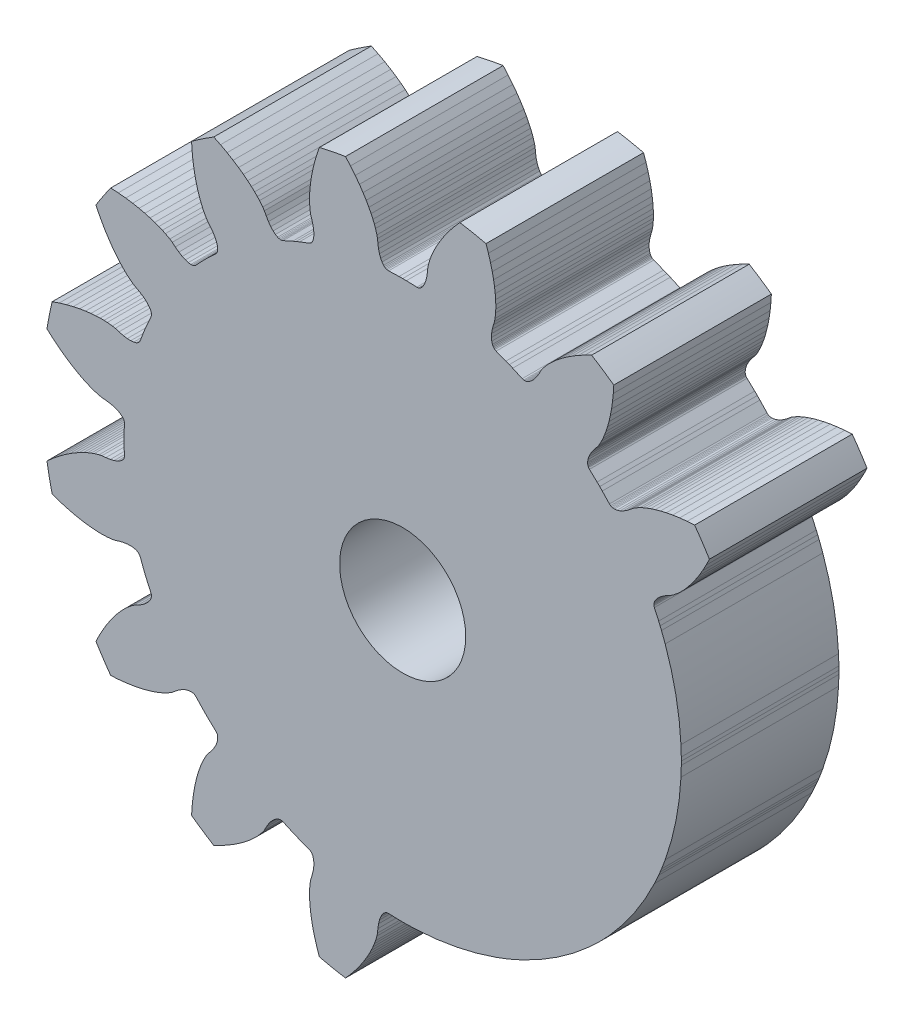
SolidWorks part; units mm, degrees
material "Thornel Mat VMA"
ref_plane "Front Plane" through (0, 0, 0) normal (0, 0, 1) x (1, 0, 0)
ref_plane "Top Plane" through (0, 0, 0) normal (0, 1, 0) x (1, 0, 0)
ref_plane "Right Plane" through (0, 0, 0) normal (1, 0, 0) x (0, 0, -1)
other "Configuration Table"
sketch "Model" plane through (0, 0, 0) normal (0, 0, 1) x (1, 0, 0)
  line L0 (0.5329, -5.7804) -> (0.6464, -5.5709)
  line L1 (0.6464, -5.5709) -> (0.7606, -5.3796)
  line L2 (0.7606, -5.3796) -> (0.8732, -5.2077)
  line L3 (0.8732, -5.2077) -> (0.9839, -5.0532)
  line L4 (0.9839, -5.0532) -> (1.0894, -4.9183)
  line L5 (1.0894, -4.9183) -> (1.1907, -4.7995)
  line L6 (1.1907, -4.7995) -> (1.285, -4.6977)
  line L7 (1.285, -4.6977) -> (1.3717, -4.6117)
  line L8 (1.3717, -4.6117) -> (1.4488, -4.5414)
  line L9 (1.4488, -4.5414) -> (1.5737, -4.4404)
  line L10 (1.5737, -4.4404) -> (1.6511, -4.3878)
  line L11 (1.6511, -4.3878) -> (1.7621, -4.3304)
  line L12 (1.7621, -4.3304) -> (1.8842, -4.2579)
  line L13 (1.8842, -4.2579) -> (1.9856, -4.1836)
  line L14 (1.9856, -4.1836) -> (2.0665, -4.1089)
  line L15 (2.0665, -4.1089) -> (2.1269, -4.0356)
  line L16 (2.1269, -4.0356) -> (2.1672, -3.9651)
  line L17 (2.1672, -3.9651) -> (2.1799, -3.9314)
  line L18 (2.1799, -3.9314) -> (2.1877, -3.899)
  line L19 (2.1877, -3.899) -> (2.1908, -3.8681)
  line L20 (2.1908, -3.8681) -> (2.189, -3.8388)
  line L21 (2.189, -3.8388) -> (2.1747, -3.7922)
  line L22 (2.1747, -3.7922) -> (2.038, -3.49)
  line L23 (2.038, -3.49) -> (1.9929, -3.3829)
  line L24 (1.9929, -3.3829) -> (1.9491, -3.2753)
  line L25 (1.9491, -3.2753) -> (1.832, -2.965)
  line L26 (1.832, -2.965) -> (1.8092, -2.9219)
  line L27 (1.8092, -2.9219) -> (1.7898, -2.9)
  line L28 (1.7898, -2.9) -> (1.7658, -2.8802)
  line L29 (1.7658, -2.8802) -> (1.7373, -2.8629)
  line L30 (1.7373, -2.8629) -> (1.7045, -2.848)
  line L31 (1.7045, -2.848) -> (1.6262, -2.8267)
  line L32 (1.6262, -2.8267) -> (1.5316, -2.8175)
  line L33 (1.5316, -2.8175) -> (1.4216, -2.8219)
  line L34 (1.4216, -2.8219) -> (1.2973, -2.8411)
  line L35 (1.2973, -2.8411) -> (1.1597, -2.8762)
  line L36 (1.1597, -2.8762) -> (1.0407, -2.9141)
  line L37 (1.0407, -2.9141) -> (0.9487, -2.9315)
  line L38 (0.9487, -2.9315) -> (0.789, -2.9485)
  line L39 (0.789, -2.9485) -> (0.6847, -2.9533)
  line L40 (0.6847, -2.9533) -> (0.5627, -2.9538)
  line L41 (0.5627, -2.9538) -> (0.424, -2.9485)
  line L42 (0.424, -2.9485) -> (0.2683, -2.9361)
  line L43 (0.2683, -2.9361) -> (0.0983, -2.9153)
  line L44 (0.0983, -2.9153) -> (-0.0892, -2.8844)
  line L45 (-0.0892, -2.8844) -> (-0.2903, -2.8425)
  line L46 (-0.2903, -2.8425) -> (-0.5064, -2.7879)
  line L47 (-0.5064, -2.7879) -> (-0.7347, -2.72)
  line L48 (-0.7347, -2.72) -> (-0.9603, -2.6427)
  line L49 (-1.1251, -1.814) -> (-0.9463, -1.6563)
  line L50 (-0.9463, -1.6563) -> (-0.7614, -1.5062)
  line L51 (-0.7614, -1.5062) -> (-0.5826, -1.3731)
  line L52 (-0.5826, -1.3731) -> (-0.4128, -1.2574)
  line L53 (-0.4128, -1.2574) -> (-0.2514, -1.157)
  line L54 (-0.2514, -1.157) -> (-0.1023, -1.0728)
  line L55 (-0.1023, -1.0728) -> (0.0367, -1.0017)
  line L56 (0.0367, -1.0017) -> (0.1629, -0.9438)
  line L57 (0.1629, -0.9438) -> (0.2758, -0.8975)
  line L58 (0.2758, -0.8975) -> (0.374, -0.862)
  line L59 (0.374, -0.862) -> (0.5281, -0.8166)
  line L60 (0.5281, -0.8166) -> (0.6197, -0.7976)
  line L61 (0.6197, -0.7976) -> (0.7441, -0.787)
  line L62 (0.7441, -0.787) -> (0.8847, -0.7668)
  line L63 (0.8847, -0.7668) -> (1.0069, -0.7369)
  line L64 (1.0069, -0.7369) -> (1.1102, -0.6989)
  line L65 (1.1102, -0.6989) -> (1.1941, -0.6542)
  line L66 (1.1941, -0.6542) -> (1.2583, -0.6045)
  line L67 (1.2583, -0.6045) -> (1.2829, -0.5783)
  line L68 (1.2829, -0.5783) -> (1.3025, -0.5513)
  line L69 (1.3025, -0.5513) -> (1.3171, -0.5239)
  line L70 (1.3171, -0.5239) -> (1.3267, -0.4962)
  line L71 (1.3267, -0.4962) -> (1.3313, -0.4477)
  line L72 (1.3313, -0.4477) -> (1.3207, -0.1162)
  line L73 (1.3207, -0.1162) -> (1.32, 0)
  line L74 (1.32, 0) -> (1.3207, 0.1162)
  line L75 (1.3207, 0.1162) -> (1.3313, 0.4477)
  line L76 (1.3313, 0.4477) -> (1.3267, 0.4962)
  line L77 (1.3267, 0.4962) -> (1.3171, 0.5239)
  line L78 (1.3171, 0.5239) -> (1.3025, 0.5513)
  line L79 (1.3025, 0.5513) -> (1.2829, 0.5783)
  line L80 (1.2829, 0.5783) -> (1.2583, 0.6045)
  line L81 (1.2583, 0.6045) -> (1.1941, 0.6542)
  line L82 (1.1941, 0.6542) -> (1.1102, 0.6989)
  line L83 (1.1102, 0.6989) -> (1.0069, 0.7369)
  line L84 (1.0069, 0.7369) -> (0.8847, 0.7668)
  line L85 (0.8847, 0.7668) -> (0.7441, 0.787)
  line L86 (0.7441, 0.787) -> (0.6197, 0.7976)
  line L87 (0.6197, 0.7976) -> (0.5281, 0.8166)
  line L88 (0.5281, 0.8166) -> (0.374, 0.862)
  line L89 (0.374, 0.862) -> (0.2758, 0.8975)
  line L90 (0.2758, 0.8975) -> (0.1629, 0.9438)
  line L91 (0.1629, 0.9438) -> (0.0367, 1.0017)
  line L92 (0.0367, 1.0017) -> (-0.1023, 1.0728)
  line L93 (-0.1023, 1.0728) -> (-0.2514, 1.157)
  line L94 (-0.2514, 1.157) -> (-0.4128, 1.2574)
  line L95 (-0.4128, 1.2574) -> (-0.5826, 1.3731)
  line L96 (-0.5826, 1.3731) -> (-0.7614, 1.5062)
  line L97 (-0.7614, 1.5062) -> (-0.9463, 1.6563)
  line L98 (-0.9463, 1.6563) -> (-1.1251, 1.814)
  line L99 (-0.9603, 2.6427) -> (-0.7347, 2.72)
  line L100 (-0.7347, 2.72) -> (-0.5064, 2.7879)
  line L101 (-0.5064, 2.7879) -> (-0.2903, 2.8425)
  line L102 (-0.2903, 2.8425) -> (-0.0892, 2.8844)
  line L103 (-0.0892, 2.8844) -> (0.0983, 2.9153)
  line L104 (0.0983, 2.9153) -> (0.2683, 2.9361)
  line L105 (0.2683, 2.9361) -> (0.424, 2.9485)
  line L106 (0.424, 2.9485) -> (0.5627, 2.9538)
  line L107 (0.5627, 2.9538) -> (0.6847, 2.9533)
  line L108 (0.6847, 2.9533) -> (0.789, 2.9485)
  line L109 (0.789, 2.9485) -> (0.9487, 2.9315)
  line L110 (0.9487, 2.9315) -> (1.0407, 2.9141)
  line L111 (1.0407, 2.9141) -> (1.1597, 2.8762)
  line L112 (1.1597, 2.8762) -> (1.2973, 2.8411)
  line L113 (1.2973, 2.8411) -> (1.4216, 2.8219)
  line L114 (1.4216, 2.8219) -> (1.5316, 2.8175)
  line L115 (1.5316, 2.8175) -> (1.6262, 2.8267)
  line L116 (1.6262, 2.8267) -> (1.7045, 2.848)
  line L117 (1.7045, 2.848) -> (1.7373, 2.8629)
  line L118 (1.7373, 2.8629) -> (1.7658, 2.8802)
  line L119 (1.7658, 2.8802) -> (1.7898, 2.9)
  line L120 (1.7898, 2.9) -> (1.8092, 2.9219)
  line L121 (1.8092, 2.9219) -> (1.832, 2.965)
  line L122 (1.832, 2.965) -> (1.9491, 3.2753)
  line L123 (1.9491, 3.2753) -> (1.9929, 3.3829)
  line L124 (1.9929, 3.3829) -> (2.038, 3.49)
  line L125 (2.038, 3.49) -> (2.1747, 3.7922)
  line L126 (2.1747, 3.7922) -> (2.189, 3.8388)
  line L127 (2.189, 3.8388) -> (2.1908, 3.8681)
  line L128 (2.1908, 3.8681) -> (2.1877, 3.899)
  line L129 (2.1877, 3.899) -> (2.1799, 3.9314)
  line L130 (2.1799, 3.9314) -> (2.1672, 3.9651)
  line L131 (2.1672, 3.9651) -> (2.1269, 4.0356)
  line L132 (2.1269, 4.0356) -> (2.0665, 4.1089)
  line L133 (2.0665, 4.1089) -> (1.9856, 4.1836)
  line L134 (1.9856, 4.1836) -> (1.8842, 4.2579)
  line L135 (1.8842, 4.2579) -> (1.7621, 4.3304)
  line L136 (1.7621, 4.3304) -> (1.6511, 4.3878)
  line L137 (1.6511, 4.3878) -> (1.5737, 4.4404)
  line L138 (1.5737, 4.4404) -> (1.4488, 4.5414)
  line L139 (1.4488, 4.5414) -> (1.3717, 4.6117)
  line L140 (1.3717, 4.6117) -> (1.285, 4.6977)
  line L141 (1.285, 4.6977) -> (1.1907, 4.7995)
  line L142 (1.1907, 4.7995) -> (1.0894, 4.9183)
  line L143 (1.0894, 4.9183) -> (0.9839, 5.0532)
  line L144 (0.9839, 5.0532) -> (0.8732, 5.2077)
  line L145 (0.8732, 5.2077) -> (0.7606, 5.3796)
  line L146 (0.7606, 5.3796) -> (0.6464, 5.5709)
  line L147 (0.6464, 5.5709) -> (0.5329, 5.7804)
  line L148 (0.5329, 5.7804) -> (0.4281, 5.9946)
  line L149 (0.8975, 6.6971) -> (1.1355, 6.6822)
  line L150 (1.1355, 6.6822) -> (1.3724, 6.6576)
  line L151 (1.3724, 6.6576) -> (1.5929, 6.6253)
  line L152 (1.5929, 6.6253) -> (1.7948, 6.587)
  line L153 (1.7948, 6.587) -> (1.9799, 6.5438)
  line L154 (1.9799, 6.5438) -> (2.1449, 6.498)
  line L155 (2.1449, 6.498) -> (2.2934, 6.4499)
  line L156 (2.2934, 6.4499) -> (2.4236, 6.4017)
  line L157 (2.4236, 6.4017) -> (2.5362, 6.3545)
  line L158 (2.5362, 6.3545) -> (2.6307, 6.3102)
  line L159 (2.6307, 6.3102) -> (2.7718, 6.2334)
  line L160 (2.7718, 6.2334) -> (2.85, 6.1821)
  line L161 (2.85, 6.1821) -> (2.9455, 6.1015)
  line L162 (2.9455, 6.1015) -> (3.0592, 6.0164)
  line L163 (3.0592, 6.0164) -> (3.1667, 5.9511)
  line L164 (3.1667, 5.9511) -> (3.2666, 5.905)
  line L165 (3.2666, 5.905) -> (3.3575, 5.8773)
  line L166 (3.3575, 5.8773) -> (3.4381, 5.867)
  line L167 (3.4381, 5.867) -> (3.4741, 5.8682)
  line L168 (3.4741, 5.8682) -> (3.507, 5.8733)
  line L169 (3.507, 5.8733) -> (3.5367, 5.8824)
  line L170 (3.5367, 5.8824) -> (3.563, 5.8952)
  line L171 (3.563, 5.8952) -> (3.6006, 5.9262)
  line L172 (3.6006, 5.9262) -> (3.8275, 6.1682)
  line L173 (3.8275, 6.1682) -> (3.9092, 6.2508)
  line L174 (3.9092, 6.2508) -> (3.9918, 6.3325)
  line L175 (3.9918, 6.3325) -> (4.2338, 6.5594)
  line L176 (4.2338, 6.5594) -> (4.2648, 6.597)
  line L177 (4.2648, 6.597) -> (4.2776, 6.6233)
  line L178 (4.2776, 6.6233) -> (4.2867, 6.653)
  line L179 (4.2867, 6.653) -> (4.2918, 6.6859)
  line L180 (4.2918, 6.6859) -> (4.293, 6.7219)
  line L181 (4.293, 6.7219) -> (4.2827, 6.8025)
  line L182 (4.2827, 6.8025) -> (4.255, 6.8934)
  line L183 (4.255, 6.8934) -> (4.2089, 6.9933)
  line L184 (4.2089, 6.9933) -> (4.1436, 7.1008)
  line L185 (4.1436, 7.1008) -> (4.0585, 7.2145)
  line L186 (4.0585, 7.2145) -> (3.9779, 7.31)
  line L187 (3.9779, 7.31) -> (3.9266, 7.3882)
  line L188 (3.9266, 7.3882) -> (3.8498, 7.5293)
  line L189 (3.8498, 7.5293) -> (3.8055, 7.6238)
  line L190 (3.8055, 7.6238) -> (3.7583, 7.7364)
  line L191 (3.7583, 7.7364) -> (3.7101, 7.8666)
  line L192 (3.7101, 7.8666) -> (3.662, 8.0151)
  line L193 (3.662, 8.0151) -> (3.6162, 8.1801)
  line L194 (3.6162, 8.1801) -> (3.573, 8.3652)
  line L195 (3.573, 8.3652) -> (3.5347, 8.5671)
  line L196 (3.5347, 8.5671) -> (3.5024, 8.7876)
  line L197 (3.5024, 8.7876) -> (3.4778, 9.0245)
  line L198 (3.4778, 9.0245) -> (3.4629, 9.2625)
  line L199 (4.1654, 9.7319) -> (4.3796, 9.6271)
  line L200 (4.3796, 9.6271) -> (4.5891, 9.5136)
  line L201 (4.5891, 9.5136) -> (4.7804, 9.3994)
  line L202 (4.7804, 9.3994) -> (4.9523, 9.2868)
  line L203 (4.9523, 9.2868) -> (5.1068, 9.1761)
  line L204 (5.1068, 9.1761) -> (5.2417, 9.0706)
  line L205 (5.2417, 9.0706) -> (5.3605, 8.9693)
  line L206 (5.3605, 8.9693) -> (5.4623, 8.875)
  line L207 (5.4623, 8.875) -> (5.5483, 8.7883)
  line L208 (5.5483, 8.7883) -> (5.6186, 8.7112)
  line L209 (5.6186, 8.7112) -> (5.7196, 8.5863)
  line L210 (5.7196, 8.5863) -> (5.7722, 8.5089)
  line L211 (5.7722, 8.5089) -> (5.8296, 8.3979)
  line L212 (5.8296, 8.3979) -> (5.9021, 8.2758)
  line L213 (5.9021, 8.2758) -> (5.9764, 8.1744)
  line L214 (5.9764, 8.1744) -> (6.0511, 8.0935)
  line L215 (6.0511, 8.0935) -> (6.1244, 8.0331)
  line L216 (6.1244, 8.0331) -> (6.1949, 7.9928)
  line L217 (6.1949, 7.9928) -> (6.2286, 7.9801)
  line L218 (6.2286, 7.9801) -> (6.261, 7.9723)
  line L219 (6.261, 7.9723) -> (6.2919, 7.9692)
  line L220 (6.2919, 7.9692) -> (6.3212, 7.971)
  line L221 (6.3212, 7.971) -> (6.3678, 7.9853)
  line L222 (6.3678, 7.9853) -> (6.67, 8.122)
  line L223 (6.67, 8.122) -> (6.7771, 8.1671)
  line L224 (6.7771, 8.1671) -> (6.8847, 8.2109)
  line L225 (6.8847, 8.2109) -> (7.195, 8.328)
  line L226 (7.195, 8.328) -> (7.2381, 8.3508)
  line L227 (7.2381, 8.3508) -> (7.26, 8.3702)
  line L228 (7.26, 8.3702) -> (7.2798, 8.3942)
  line L229 (7.2798, 8.3942) -> (7.2971, 8.4227)
  line L230 (7.2971, 8.4227) -> (7.312, 8.4555)
  line L231 (7.312, 8.4555) -> (7.3333, 8.5338)
  line L232 (7.3333, 8.5338) -> (7.3425, 8.6284)
  line L233 (7.3425, 8.6284) -> (7.3381, 8.7384)
  line L234 (7.3381, 8.7384) -> (7.3189, 8.8627)
  line L235 (7.3189, 8.8627) -> (7.2838, 9.0003)
  line L236 (7.2838, 9.0003) -> (7.2459, 9.1193)
  line L237 (7.2459, 9.1193) -> (7.2285, 9.2113)
  line L238 (7.2285, 9.2113) -> (7.2115, 9.371)
  line L239 (7.2115, 9.371) -> (7.2067, 9.4753)
  line L240 (7.2067, 9.4753) -> (7.2062, 9.5973)
  line L241 (7.2062, 9.5973) -> (7.2115, 9.736)
  line L242 (7.2115, 9.736) -> (7.2239, 9.8917)
  line L243 (7.2239, 9.8917) -> (7.2447, 10.0617)
  line L244 (7.2447, 10.0617) -> (7.2756, 10.2492)
  line L245 (7.2756, 10.2492) -> (7.3175, 10.4503)
  line L246 (7.3175, 10.4503) -> (7.3721, 10.6664)
  line L247 (7.3721, 10.6664) -> (7.44, 10.8947)
  line L248 (7.44, 10.8947) -> (7.5173, 11.1203)
  line L249 (8.346, 11.2851) -> (8.5037, 11.1063)
  line L250 (8.5037, 11.1063) -> (8.6538, 10.9214)
  line L251 (8.6538, 10.9214) -> (8.7869, 10.7426)
  line L252 (8.7869, 10.7426) -> (8.9026, 10.5728)
  line L253 (8.9026, 10.5728) -> (9.003, 10.4114)
  line L254 (9.003, 10.4114) -> (9.0872, 10.2623)
  line L255 (9.0872, 10.2623) -> (9.1583, 10.1233)
  line L256 (9.1583, 10.1233) -> (9.2162, 9.9971)
  line L257 (9.2162, 9.9971) -> (9.2625, 9.8842)
  line L258 (9.2625, 9.8842) -> (9.298, 9.786)
  line L259 (9.298, 9.786) -> (9.3434, 9.6319)
  line L260 (9.3434, 9.6319) -> (9.3624, 9.5403)
  line L261 (9.3624, 9.5403) -> (9.373, 9.4159)
  line L262 (9.373, 9.4159) -> (9.3932, 9.2753)
  line L263 (9.3932, 9.2753) -> (9.4231, 9.1531)
  line L264 (9.4231, 9.1531) -> (9.4611, 9.0498)
  line L265 (9.4611, 9.0498) -> (9.5057, 8.9659)
  line L266 (9.5057, 8.9659) -> (9.5555, 8.9017)
  line L267 (9.5555, 8.9017) -> (9.5817, 8.8771)
  line L268 (9.5817, 8.8771) -> (9.6087, 8.8575)
  line L269 (9.6087, 8.8575) -> (9.6361, 8.8429)
  line L270 (9.6361, 8.8429) -> (9.6638, 8.8333)
  line L271 (9.6638, 8.8333) -> (9.7123, 8.8287)
  line L272 (9.7123, 8.8287) -> (10.0438, 8.8393)
  line L273 (10.0438, 8.8393) -> (10.16, 8.84)
  line L274 (10.16, 8.84) -> (10.2762, 8.8393)
  line L275 (10.2762, 8.8393) -> (10.6077, 8.8287)
  line L276 (10.6077, 8.8287) -> (10.6562, 8.8333)
  line L277 (10.6562, 8.8333) -> (10.6839, 8.8429)
  line L278 (10.6839, 8.8429) -> (10.7113, 8.8575)
  line L279 (10.7113, 8.8575) -> (10.7383, 8.8771)
  line L280 (10.7383, 8.8771) -> (10.7645, 8.9017)
  line L281 (10.7645, 8.9017) -> (10.8142, 8.9659)
  line L282 (10.8142, 8.9659) -> (10.8589, 9.0498)
  line L283 (10.8589, 9.0498) -> (10.8969, 9.1531)
  line L284 (10.8969, 9.1531) -> (10.9268, 9.2753)
  line L285 (10.9268, 9.2753) -> (10.947, 9.4159)
  line L286 (10.947, 9.4159) -> (10.9576, 9.5403)
  line L287 (10.9576, 9.5403) -> (10.9766, 9.6319)
  line L288 (10.9766, 9.6319) -> (11.022, 9.786)
  line L289 (11.022, 9.786) -> (11.0575, 9.8842)
  line L290 (11.0575, 9.8842) -> (11.1038, 9.9971)
  line L291 (11.1038, 9.9971) -> (11.1617, 10.1233)
  line L292 (11.1617, 10.1233) -> (11.2328, 10.2623)
  line L293 (11.2328, 10.2623) -> (11.317, 10.4114)
  line L294 (11.317, 10.4114) -> (11.4174, 10.5728)
  line L295 (11.4174, 10.5728) -> (11.5331, 10.7426)
  line L296 (11.5331, 10.7426) -> (11.6661, 10.9214)
  line L297 (11.6661, 10.9214) -> (11.8163, 11.1063)
  line L298 (11.8163, 11.1063) -> (11.974, 11.2851)
  line L299 (12.8027, 11.1203) -> (12.88, 10.8947)
  line L300 (12.88, 10.8947) -> (12.9479, 10.6664)
  line L301 (12.9479, 10.6664) -> (13.0025, 10.4503)
  line L302 (13.0025, 10.4503) -> (13.0444, 10.2492)
  line L303 (13.0444, 10.2492) -> (13.0753, 10.0617)
  line L304 (13.0753, 10.0617) -> (13.0961, 9.8917)
  line L305 (13.0961, 9.8917) -> (13.1085, 9.736)
  line L306 (13.1085, 9.736) -> (13.1138, 9.5973)
  line L307 (13.1138, 9.5973) -> (13.1133, 9.4753)
  line L308 (13.1133, 9.4753) -> (13.1085, 9.371)
  line L309 (13.1085, 9.371) -> (13.0915, 9.2113)
  line L310 (13.0915, 9.2113) -> (13.0741, 9.1193)
  line L311 (13.0741, 9.1193) -> (13.0362, 9.0003)
  line L312 (13.0362, 9.0003) -> (13.0011, 8.8627)
  line L313 (13.0011, 8.8627) -> (12.9819, 8.7384)
  line L314 (12.9819, 8.7384) -> (12.9775, 8.6284)
  line L315 (12.9775, 8.6284) -> (12.9867, 8.5338)
  line L316 (12.9867, 8.5338) -> (13.008, 8.4555)
  line L317 (13.008, 8.4555) -> (13.0229, 8.4227)
  line L318 (13.0229, 8.4227) -> (13.0402, 8.3942)
  line L319 (13.0402, 8.3942) -> (13.06, 8.3702)
  line L320 (13.06, 8.3702) -> (13.0819, 8.3508)
  line L321 (13.0819, 8.3508) -> (13.125, 8.328)
  line L322 (13.125, 8.328) -> (13.4353, 8.2109)
  line L323 (13.4353, 8.2109) -> (13.5429, 8.1671)
  line L324 (13.5429, 8.1671) -> (13.65, 8.122)
  line L325 (13.65, 8.122) -> (13.9522, 7.9853)
  line L326 (13.9522, 7.9853) -> (13.9988, 7.971)
  line L327 (13.9988, 7.971) -> (14.0281, 7.9692)
  line L328 (14.0281, 7.9692) -> (14.059, 7.9723)
  line L329 (14.059, 7.9723) -> (14.0914, 7.9801)
  line L330 (14.0914, 7.9801) -> (14.1251, 7.9928)
  line L331 (14.1251, 7.9928) -> (14.1956, 8.0331)
  line L332 (14.1956, 8.0331) -> (14.2689, 8.0935)
  line L333 (14.2689, 8.0935) -> (14.3436, 8.1744)
  line L334 (14.3436, 8.1744) -> (14.4179, 8.2758)
  line L335 (14.4179, 8.2758) -> (14.4904, 8.3979)
  line L336 (14.4904, 8.3979) -> (14.5478, 8.5089)
  line L337 (14.5478, 8.5089) -> (14.6004, 8.5863)
  line L338 (14.6004, 8.5863) -> (14.7014, 8.7112)
  line L339 (14.7014, 8.7112) -> (14.7717, 8.7883)
  line L340 (14.7717, 8.7883) -> (14.8577, 8.875)
  line L341 (14.8577, 8.875) -> (14.9595, 8.9693)
  line L342 (14.9595, 8.9693) -> (15.0783, 9.0706)
  line L343 (15.0783, 9.0706) -> (15.2132, 9.1761)
  line L344 (15.2132, 9.1761) -> (15.3677, 9.2868)
  line L345 (15.3677, 9.2868) -> (15.5396, 9.3994)
  line L346 (15.5396, 9.3994) -> (15.7309, 9.5136)
  line L347 (15.7309, 9.5136) -> (15.9404, 9.6271)
  line L348 (15.9404, 9.6271) -> (16.1546, 9.7319)
  line L349 (16.8571, 9.2625) -> (16.8422, 9.0245)
  line L350 (16.8422, 9.0245) -> (16.8176, 8.7876)
  line L351 (16.8176, 8.7876) -> (16.7853, 8.5671)
  line L352 (16.7853, 8.5671) -> (16.747, 8.3652)
  line L353 (16.747, 8.3652) -> (16.7038, 8.1801)
  line L354 (16.7038, 8.1801) -> (16.658, 8.0151)
  line L355 (16.658, 8.0151) -> (16.6099, 7.8666)
  line L356 (16.6099, 7.8666) -> (16.5617, 7.7364)
  line L357 (16.5617, 7.7364) -> (16.5145, 7.6238)
  line L358 (16.5145, 7.6238) -> (16.4702, 7.5293)
  line L359 (16.4702, 7.5293) -> (16.3934, 7.3882)
  line L360 (16.3934, 7.3882) -> (16.3421, 7.31)
  line L361 (16.3421, 7.31) -> (16.2615, 7.2145)
  line L362 (16.2615, 7.2145) -> (16.1764, 7.1008)
  line L363 (16.1764, 7.1008) -> (16.1111, 6.9933)
  line L364 (16.1111, 6.9933) -> (16.065, 6.8934)
  line L365 (16.065, 6.8934) -> (16.0373, 6.8025)
  line L366 (16.0373, 6.8025) -> (16.027, 6.7219)
  line L367 (16.027, 6.7219) -> (16.0282, 6.6859)
  line L368 (16.0282, 6.6859) -> (16.0333, 6.653)
  line L369 (16.0333, 6.653) -> (16.0424, 6.6233)
  line L370 (16.0424, 6.6233) -> (16.0552, 6.597)
  line L371 (16.0552, 6.597) -> (16.0862, 6.5594)
  line L372 (16.0862, 6.5594) -> (16.3282, 6.3325)
  line L373 (16.3282, 6.3325) -> (16.4108, 6.2508)
  line L374 (16.4108, 6.2508) -> (16.4925, 6.1682)
  line L375 (16.4925, 6.1682) -> (16.7194, 5.9262)
  line L376 (16.7194, 5.9262) -> (16.757, 5.8952)
  line L377 (16.757, 5.8952) -> (16.7833, 5.8824)
  line L378 (16.7833, 5.8824) -> (16.813, 5.8733)
  line L379 (16.813, 5.8733) -> (16.8459, 5.8682)
  line L380 (16.8459, 5.8682) -> (16.8819, 5.867)
  line L381 (16.8819, 5.867) -> (16.9625, 5.8773)
  line L382 (16.9625, 5.8773) -> (17.0534, 5.905)
  line L383 (17.0534, 5.905) -> (17.1533, 5.9511)
  line L384 (17.1533, 5.9511) -> (17.2608, 6.0164)
  line L385 (17.2608, 6.0164) -> (17.3745, 6.1015)
  line L386 (17.3745, 6.1015) -> (17.47, 6.1821)
  line L387 (17.47, 6.1821) -> (17.5482, 6.2334)
  line L388 (17.5482, 6.2334) -> (17.6893, 6.3102)
  line L389 (17.6893, 6.3102) -> (17.7838, 6.3545)
  line L390 (17.7838, 6.3545) -> (17.8964, 6.4017)
  line L391 (17.8964, 6.4017) -> (18.0266, 6.4499)
  line L392 (18.0266, 6.4499) -> (18.1751, 6.498)
  line L393 (18.1751, 6.498) -> (18.3401, 6.5438)
  line L394 (18.3401, 6.5438) -> (18.5252, 6.587)
  line L395 (18.5252, 6.587) -> (18.7271, 6.6253)
  line L396 (18.7271, 6.6253) -> (18.9476, 6.6576)
  line L397 (18.9476, 6.6576) -> (19.1845, 6.6822)
  line L398 (19.1845, 6.6822) -> (19.4225, 6.6971)
  line L399 (19.8919, 5.9946) -> (19.7871, 5.7804)
  line L400 (19.7871, 5.7804) -> (19.6736, 5.5709)
  line L401 (19.6736, 5.5709) -> (19.5594, 5.3796)
  line L402 (19.5594, 5.3796) -> (19.4468, 5.2077)
  line L403 (19.4468, 5.2077) -> (19.3361, 5.0532)
  line L404 (19.3361, 5.0532) -> (19.2306, 4.9183)
  line L405 (19.2306, 4.9183) -> (19.1293, 4.7995)
  line L406 (19.1293, 4.7995) -> (19.035, 4.6977)
  line L407 (19.035, 4.6977) -> (18.9483, 4.6117)
  line L408 (18.9483, 4.6117) -> (18.8712, 4.5414)
  line L409 (18.8712, 4.5414) -> (18.7463, 4.4404)
  line L410 (18.7463, 4.4404) -> (18.6689, 4.3878)
  line L411 (18.6689, 4.3878) -> (18.5579, 4.3304)
  line L412 (18.5579, 4.3304) -> (18.4358, 4.2579)
  line L413 (18.4358, 4.2579) -> (18.3344, 4.1836)
  line L414 (18.3344, 4.1836) -> (18.2535, 4.1089)
  line L415 (18.2535, 4.1089) -> (18.1931, 4.0356)
  line L416 (18.1931, 4.0356) -> (18.1528, 3.9651)
  line L417 (18.1528, 3.9651) -> (18.1401, 3.9314)
  line L418 (18.1401, 3.9314) -> (18.1323, 3.899)
  line L419 (18.1323, 3.899) -> (18.1292, 3.8681)
  line L420 (18.1292, 3.8681) -> (18.131, 3.8388)
  line L421 (18.131, 3.8388) -> (18.1453, 3.7922)
  line L422 (18.1453, 3.7922) -> (18.282, 3.49)
  line L423 (18.282, 3.49) -> (18.3271, 3.3829)
  line L424 (18.3271, 3.3829) -> (18.3709, 3.2753)
  line L425 (18.3709, 3.2753) -> (18.488, 2.965)
  line L426 (18.488, 2.965) -> (18.5108, 2.9219)
  line L427 (18.5108, 2.9219) -> (18.5302, 2.9)
  line L428 (18.5302, 2.9) -> (18.5542, 2.8802)
  line L429 (18.5542, 2.8802) -> (18.5827, 2.8629)
  line L430 (18.5827, 2.8629) -> (18.6155, 2.848)
  line L431 (18.6155, 2.848) -> (18.6938, 2.8267)
  line L432 (18.6938, 2.8267) -> (18.7884, 2.8175)
  line L433 (18.7884, 2.8175) -> (18.8984, 2.8219)
  line L434 (18.8984, 2.8219) -> (19.0227, 2.8411)
  line L435 (19.0227, 2.8411) -> (19.1603, 2.8762)
  line L436 (19.1603, 2.8762) -> (19.2793, 2.9141)
  line L437 (19.2793, 2.9141) -> (19.3713, 2.9315)
  line L438 (19.3713, 2.9315) -> (19.531, 2.9485)
  line L439 (19.531, 2.9485) -> (19.6353, 2.9533)
  line L440 (19.6353, 2.9533) -> (19.7573, 2.9538)
  line L441 (19.7573, 2.9538) -> (19.896, 2.9485)
  line L442 (19.896, 2.9485) -> (20.0517, 2.9361)
  line L443 (20.0517, 2.9361) -> (20.2217, 2.9153)
  line L444 (20.2217, 2.9153) -> (20.4092, 2.8844)
  line L445 (20.4092, 2.8844) -> (20.6103, 2.8425)
  line L446 (20.6103, 2.8425) -> (20.8264, 2.7879)
  line L447 (20.8264, 2.7879) -> (21.0547, 2.72)
  line L448 (21.0547, 2.72) -> (21.2803, 2.6427)
  line L449 (21.4451, 1.814) -> (21.2663, 1.6563)
  line L450 (21.2663, 1.6563) -> (21.0813, 1.5062)
  line L451 (21.0813, 1.5062) -> (20.9026, 1.3731)
  line L452 (20.9026, 1.3731) -> (20.7328, 1.2574)
  line L453 (20.7328, 1.2574) -> (20.5714, 1.157)
  line L454 (20.5714, 1.157) -> (20.4223, 1.0728)
  line L455 (20.4223, 1.0728) -> (20.2833, 1.0017)
  line L456 (20.2833, 1.0017) -> (20.1571, 0.9438)
  line L457 (20.1571, 0.9438) -> (20.0442, 0.8975)
  line L458 (20.0442, 0.8975) -> (19.946, 0.862)
  line L459 (19.946, 0.862) -> (19.7919, 0.8166)
  line L460 (19.7919, 0.8166) -> (19.7003, 0.7976)
  line L461 (19.7003, 0.7976) -> (19.5759, 0.787)
  line L462 (19.5759, 0.787) -> (19.4353, 0.7668)
  line L463 (19.4353, 0.7668) -> (19.3131, 0.7369)
  line L464 (19.3131, 0.7369) -> (19.2098, 0.6989)
  line L465 (19.2098, 0.6989) -> (19.1259, 0.6542)
  line L466 (19.1259, 0.6542) -> (19.0617, 0.6045)
  line L467 (19.0617, 0.6045) -> (19.0371, 0.5783)
  line L468 (19.0371, 0.5783) -> (19.0175, 0.5513)
  line L469 (19.0175, 0.5513) -> (19.0029, 0.5239)
  line L470 (19.0029, 0.5239) -> (18.9933, 0.4962)
  line L471 (18.9933, 0.4962) -> (18.9887, 0.4477)
  line L472 (18.9887, 0.4477) -> (18.9993, 0.1162)
  line L473 (18.9993, 0.1162) -> (19, 0)
  line L474 (19, 0) -> (18.9993, -0.1162)
  line L475 (18.9993, -0.1162) -> (18.9887, -0.4477)
  line L476 (18.9887, -0.4477) -> (18.9933, -0.4962)
  line L477 (18.9933, -0.4962) -> (19.0029, -0.5239)
  line L478 (19.0029, -0.5239) -> (19.0175, -0.5513)
  line L479 (19.0175, -0.5513) -> (19.0371, -0.5783)
  line L480 (19.0371, -0.5783) -> (19.0617, -0.6045)
  line L481 (19.0617, -0.6045) -> (19.1259, -0.6542)
  line L482 (19.1259, -0.6542) -> (19.2098, -0.6989)
  line L483 (19.2098, -0.6989) -> (19.3131, -0.7369)
  line L484 (19.3131, -0.7369) -> (19.4353, -0.7668)
  line L485 (19.4353, -0.7668) -> (19.5759, -0.787)
  line L486 (19.5759, -0.787) -> (19.7003, -0.7976)
  line L487 (19.7003, -0.7976) -> (19.7919, -0.8166)
  line L488 (19.7919, -0.8166) -> (19.946, -0.862)
  line L489 (19.946, -0.862) -> (20.0442, -0.8975)
  line L490 (20.0442, -0.8975) -> (20.1571, -0.9438)
  line L491 (20.1571, -0.9438) -> (20.2833, -1.0017)
  line L492 (20.2833, -1.0017) -> (20.4223, -1.0728)
  line L493 (20.4223, -1.0728) -> (20.5714, -1.157)
  line L494 (20.5714, -1.157) -> (20.7328, -1.2574)
  line L495 (20.7328, -1.2574) -> (20.9026, -1.3731)
  line L496 (20.9026, -1.3731) -> (21.0813, -1.5062)
  line L497 (21.0813, -1.5062) -> (21.2663, -1.6563)
  line L498 (21.2663, -1.6563) -> (21.4451, -1.814)
  line L499 (21.2803, -2.6427) -> (21.0547, -2.72)
  line L500 (21.0547, -2.72) -> (20.8264, -2.7879)
  line L501 (20.8264, -2.7879) -> (20.6103, -2.8425)
  line L502 (20.6103, -2.8425) -> (20.4092, -2.8844)
  line L503 (20.4092, -2.8844) -> (20.2217, -2.9153)
  line L504 (20.2217, -2.9153) -> (20.0517, -2.9361)
  line L505 (20.0517, -2.9361) -> (19.896, -2.9485)
  line L506 (19.896, -2.9485) -> (19.7573, -2.9538)
  line L507 (19.7573, -2.9538) -> (19.6353, -2.9533)
  line L508 (19.6353, -2.9533) -> (19.531, -2.9485)
  line L509 (19.531, -2.9485) -> (19.3713, -2.9315)
  line L510 (19.3713, -2.9315) -> (19.2793, -2.9141)
  line L511 (19.2793, -2.9141) -> (19.1603, -2.8762)
  line L512 (19.1603, -2.8762) -> (19.0227, -2.8411)
  line L513 (19.0227, -2.8411) -> (18.8984, -2.8219)
  line L514 (18.8984, -2.8219) -> (18.7884, -2.8175)
  line L515 (18.7884, -2.8175) -> (18.6938, -2.8267)
  line L516 (18.6938, -2.8267) -> (18.6155, -2.848)
  line L517 (18.6155, -2.848) -> (18.5827, -2.8629)
  line L518 (18.5827, -2.8629) -> (18.5542, -2.8802)
  line L519 (18.5542, -2.8802) -> (18.5302, -2.9)
  line L520 (18.5302, -2.9) -> (18.5108, -2.9219)
  line L521 (18.5108, -2.9219) -> (18.488, -2.965)
  line L522 (18.488, -2.965) -> (18.3709, -3.2753)
  line L523 (18.3709, -3.2753) -> (18.3271, -3.3829)
  line L524 (18.3271, -3.3829) -> (18.282, -3.49)
  line L525 (18.282, -3.49) -> (18.1453, -3.7922)
  line L526 (18.1453, -3.7922) -> (18.131, -3.8388)
  line L527 (18.131, -3.8388) -> (18.1292, -3.8681)
  line L528 (18.1292, -3.8681) -> (18.1323, -3.899)
  line L529 (18.1323, -3.899) -> (18.1401, -3.9314)
  line L530 (18.1401, -3.9314) -> (18.1528, -3.9651)
  line L531 (18.1528, -3.9651) -> (18.1931, -4.0356)
  line L532 (18.1931, -4.0356) -> (18.2535, -4.1089)
  line L533 (18.2535, -4.1089) -> (18.3344, -4.1836)
  line L534 (18.3344, -4.1836) -> (18.4358, -4.2579)
  line L535 (18.4358, -4.2579) -> (18.5579, -4.3304)
  line L536 (18.5579, -4.3304) -> (18.6689, -4.3878)
  line L537 (18.6689, -4.3878) -> (18.7463, -4.4404)
  line L538 (18.7463, -4.4404) -> (18.8712, -4.5414)
  line L539 (18.8712, -4.5414) -> (18.9483, -4.6117)
  line L540 (18.9483, -4.6117) -> (19.035, -4.6977)
  line L541 (19.035, -4.6977) -> (19.1293, -4.7995)
  line L542 (19.1293, -4.7995) -> (19.2306, -4.9183)
  line L543 (19.2306, -4.9183) -> (19.3361, -5.0532)
  line L544 (19.3361, -5.0532) -> (19.4468, -5.2077)
  line L545 (19.4468, -5.2077) -> (19.5594, -5.3796)
  line L546 (19.5594, -5.3796) -> (19.6736, -5.5709)
  line L547 (19.6736, -5.5709) -> (19.7871, -5.7804)
  line L548 (19.7871, -5.7804) -> (19.8919, -5.9946)
  line L549 (19.4225, -6.6971) -> (19.1845, -6.6822)
  line L550 (19.1845, -6.6822) -> (18.9476, -6.6576)
  line L551 (18.9476, -6.6576) -> (18.7271, -6.6253)
  line L552 (18.7271, -6.6253) -> (18.5252, -6.587)
  line L553 (18.5252, -6.587) -> (18.3401, -6.5438)
  line L554 (18.3401, -6.5438) -> (18.1751, -6.498)
  line L555 (18.1751, -6.498) -> (18.0266, -6.4499)
  line L556 (18.0266, -6.4499) -> (17.8964, -6.4017)
  line L557 (17.8964, -6.4017) -> (17.7838, -6.3545)
  line L558 (17.7838, -6.3545) -> (17.6893, -6.3102)
  line L559 (17.6893, -6.3102) -> (17.5482, -6.2334)
  line L560 (17.5482, -6.2334) -> (17.47, -6.1821)
  line L561 (17.47, -6.1821) -> (17.3745, -6.1015)
  line L562 (17.3745, -6.1015) -> (17.2608, -6.0164)
  line L563 (17.2608, -6.0164) -> (17.1533, -5.9511)
  line L564 (17.1533, -5.9511) -> (17.0534, -5.905)
  line L565 (17.0534, -5.905) -> (16.9625, -5.8773)
  line L566 (16.9625, -5.8773) -> (16.8819, -5.867)
  line L567 (16.8819, -5.867) -> (16.8459, -5.8682)
  line L568 (16.8459, -5.8682) -> (16.813, -5.8733)
  line L569 (16.813, -5.8733) -> (16.7833, -5.8824)
  line L570 (16.7833, -5.8824) -> (16.757, -5.8952)
  line L571 (16.757, -5.8952) -> (16.7194, -5.9262)
  line L572 (16.7194, -5.9262) -> (16.4925, -6.1682)
  line L573 (16.4925, -6.1682) -> (16.4108, -6.2508)
  line L574 (16.4108, -6.2508) -> (16.3282, -6.3325)
  line L575 (16.3282, -6.3325) -> (16.0862, -6.5594)
  line L576 (16.0862, -6.5594) -> (16.0552, -6.597)
  line L577 (16.0552, -6.597) -> (16.0424, -6.6233)
  line L578 (16.0424, -6.6233) -> (16.0333, -6.653)
  line L579 (16.0333, -6.653) -> (16.0282, -6.6859)
  line L580 (16.0282, -6.6859) -> (16.027, -6.7219)
  line L581 (16.027, -6.7219) -> (16.0373, -6.8025)
  line L582 (16.0373, -6.8025) -> (16.065, -6.8934)
  line L583 (16.065, -6.8934) -> (16.1111, -6.9933)
  line L584 (16.1111, -6.9933) -> (16.1764, -7.1008)
  line L585 (16.1764, -7.1008) -> (16.2615, -7.2145)
  line L586 (16.2615, -7.2145) -> (16.3421, -7.31)
  line L587 (16.3421, -7.31) -> (16.3934, -7.3882)
  line L588 (16.3934, -7.3882) -> (16.4702, -7.5293)
  line L589 (16.4702, -7.5293) -> (16.5145, -7.6238)
  line L590 (16.5145, -7.6238) -> (16.5617, -7.7364)
  line L591 (16.5617, -7.7364) -> (16.6099, -7.8666)
  line L592 (16.6099, -7.8666) -> (16.658, -8.0151)
  line L593 (16.658, -8.0151) -> (16.7038, -8.1801)
  line L594 (16.7038, -8.1801) -> (16.747, -8.3652)
  line L595 (16.747, -8.3652) -> (16.7853, -8.5671)
  line L596 (16.7853, -8.5671) -> (16.8176, -8.7876)
  line L597 (16.8176, -8.7876) -> (16.8422, -9.0245)
  line L598 (16.8422, -9.0245) -> (16.8571, -9.2625)
  line L599 (16.1546, -9.7319) -> (15.9404, -9.6271)
  line L600 (15.9404, -9.6271) -> (15.7309, -9.5136)
  line L601 (15.7309, -9.5136) -> (15.5396, -9.3994)
  line L602 (15.5396, -9.3994) -> (15.3677, -9.2868)
  line L603 (15.3677, -9.2868) -> (15.2132, -9.1761)
  line L604 (15.2132, -9.1761) -> (15.0783, -9.0706)
  line L605 (15.0783, -9.0706) -> (14.9595, -8.9693)
  line L606 (14.9595, -8.9693) -> (14.8577, -8.875)
  line L607 (14.8577, -8.875) -> (14.7717, -8.7883)
  line L608 (14.7717, -8.7883) -> (14.7014, -8.7112)
  line L609 (14.7014, -8.7112) -> (14.6004, -8.5863)
  line L610 (14.6004, -8.5863) -> (14.5478, -8.5089)
  line L611 (14.5478, -8.5089) -> (14.4904, -8.3979)
  line L612 (14.4904, -8.3979) -> (14.4179, -8.2758)
  line L613 (14.4179, -8.2758) -> (14.3436, -8.1744)
  line L614 (14.3436, -8.1744) -> (14.2689, -8.0935)
  line L615 (14.2689, -8.0935) -> (14.1956, -8.0331)
  line L616 (14.1956, -8.0331) -> (14.1251, -7.9928)
  line L617 (14.1251, -7.9928) -> (14.0914, -7.9801)
  line L618 (14.0914, -7.9801) -> (14.059, -7.9723)
  line L619 (14.059, -7.9723) -> (14.0281, -7.9692)
  line L620 (14.0281, -7.9692) -> (13.9988, -7.971)
  line L621 (13.9988, -7.971) -> (13.9522, -7.9853)
  line L622 (13.9522, -7.9853) -> (13.65, -8.122)
  line L623 (13.65, -8.122) -> (13.5429, -8.1671)
  line L624 (13.5429, -8.1671) -> (13.4353, -8.2109)
  line L625 (13.4353, -8.2109) -> (13.125, -8.328)
  line L626 (13.125, -8.328) -> (13.0819, -8.3508)
  line L627 (13.0819, -8.3508) -> (13.06, -8.3702)
  line L628 (13.06, -8.3702) -> (13.0402, -8.3942)
  line L629 (13.0402, -8.3942) -> (13.0229, -8.4227)
  line L630 (13.0229, -8.4227) -> (13.008, -8.4555)
  line L631 (13.008, -8.4555) -> (12.9867, -8.5338)
  line L632 (12.9867, -8.5338) -> (12.9775, -8.6284)
  line L633 (12.9775, -8.6284) -> (12.9819, -8.7384)
  line L634 (12.9819, -8.7384) -> (13.0011, -8.8627)
  line L635 (13.0011, -8.8627) -> (13.0362, -9.0003)
  line L636 (13.0362, -9.0003) -> (13.0741, -9.1193)
  line L637 (13.0741, -9.1193) -> (13.0915, -9.2113)
  line L638 (13.0915, -9.2113) -> (13.1085, -9.371)
  line L639 (13.1085, -9.371) -> (13.1133, -9.4753)
  line L640 (13.1133, -9.4753) -> (13.1138, -9.5973)
  line L641 (13.1138, -9.5973) -> (13.1085, -9.736)
  line L642 (13.1085, -9.736) -> (13.0961, -9.8917)
  line L643 (13.0961, -9.8917) -> (13.0753, -10.0617)
  line L644 (13.0753, -10.0617) -> (13.0444, -10.2492)
  line L645 (13.0444, -10.2492) -> (13.0025, -10.4503)
  line L646 (13.0025, -10.4503) -> (12.9479, -10.6664)
  line L647 (12.9479, -10.6664) -> (12.88, -10.8947)
  line L648 (12.88, -10.8947) -> (12.8027, -11.1203)
  line L649 (11.974, -11.2851) -> (11.8163, -11.1063)
  line L650 (11.8163, -11.1063) -> (11.6661, -10.9214)
  line L651 (11.6661, -10.9214) -> (11.5331, -10.7426)
  line L652 (11.5331, -10.7426) -> (11.4174, -10.5728)
  line L653 (11.4174, -10.5728) -> (11.317, -10.4114)
  line L654 (11.317, -10.4114) -> (11.2328, -10.2623)
  line L655 (11.2328, -10.2623) -> (11.1617, -10.1233)
  line L656 (11.1617, -10.1233) -> (11.1038, -9.9971)
  line L657 (11.1038, -9.9971) -> (11.0575, -9.8842)
  line L658 (11.0575, -9.8842) -> (11.022, -9.786)
  line L659 (11.022, -9.786) -> (10.9766, -9.6319)
  line L660 (10.9766, -9.6319) -> (10.9576, -9.5403)
  line L661 (10.9576, -9.5403) -> (10.947, -9.4159)
  line L662 (10.947, -9.4159) -> (10.9268, -9.2753)
  line L663 (10.9268, -9.2753) -> (10.8969, -9.1531)
  line L664 (10.8969, -9.1531) -> (10.8589, -9.0498)
  line L665 (10.8589, -9.0498) -> (10.8142, -8.9659)
  line L666 (10.8142, -8.9659) -> (10.7645, -8.9017)
  line L667 (10.7645, -8.9017) -> (10.7383, -8.8771)
  line L668 (10.7383, -8.8771) -> (10.7113, -8.8575)
  line L669 (10.7113, -8.8575) -> (10.6839, -8.8429)
  line L670 (10.6839, -8.8429) -> (10.6562, -8.8333)
  line L671 (10.6562, -8.8333) -> (10.6077, -8.8287)
  line L672 (10.6077, -8.8287) -> (10.2762, -8.8393)
  line L673 (10.2762, -8.8393) -> (10.16, -8.84)
  line L674 (10.16, -8.84) -> (10.0438, -8.8393)
  line L675 (10.0438, -8.8393) -> (9.7123, -8.8287)
  line L676 (9.7123, -8.8287) -> (9.6638, -8.8333)
  line L677 (9.6638, -8.8333) -> (9.6361, -8.8429)
  line L678 (9.6361, -8.8429) -> (9.6087, -8.8575)
  line L679 (9.6087, -8.8575) -> (9.5817, -8.8771)
  line L680 (9.5817, -8.8771) -> (9.5555, -8.9017)
  line L681 (9.5555, -8.9017) -> (9.5057, -8.9659)
  line L682 (9.5057, -8.9659) -> (9.4611, -9.0498)
  line L683 (9.4611, -9.0498) -> (9.4231, -9.1531)
  line L684 (9.4231, -9.1531) -> (9.3932, -9.2753)
  line L685 (9.3932, -9.2753) -> (9.373, -9.4159)
  line L686 (9.373, -9.4159) -> (9.3624, -9.5403)
  line L687 (9.3624, -9.5403) -> (9.3434, -9.6319)
  line L688 (9.3434, -9.6319) -> (9.298, -9.786)
  line L689 (9.298, -9.786) -> (9.2625, -9.8842)
  line L690 (9.2625, -9.8842) -> (9.2162, -9.9971)
  line L691 (9.2162, -9.9971) -> (9.1583, -10.1233)
  line L692 (9.1583, -10.1233) -> (9.0872, -10.2623)
  line L693 (9.0872, -10.2623) -> (9.003, -10.4114)
  line L694 (9.003, -10.4114) -> (8.9026, -10.5728)
  line L695 (8.9026, -10.5728) -> (8.7869, -10.7426)
  line L696 (8.7869, -10.7426) -> (8.6538, -10.9214)
  line L697 (8.6538, -10.9214) -> (8.5037, -11.1063)
  line L698 (8.5037, -11.1063) -> (8.346, -11.2851)
  line L699 (7.5173, -11.1203) -> (7.44, -10.8947)
  line L700 (7.44, -10.8947) -> (7.3721, -10.6664)
  line L701 (7.3721, -10.6664) -> (7.3175, -10.4503)
  line L702 (7.3175, -10.4503) -> (7.2756, -10.2492)
  line L703 (7.2756, -10.2492) -> (7.2447, -10.0617)
  line L704 (7.2447, -10.0617) -> (7.2239, -9.8917)
  line L705 (7.2239, -9.8917) -> (7.2115, -9.736)
  line L706 (7.2115, -9.736) -> (7.2062, -9.5973)
  line L707 (7.2062, -9.5973) -> (7.2067, -9.4753)
  line L708 (7.2067, -9.4753) -> (7.2115, -9.371)
  line L709 (7.2115, -9.371) -> (7.2285, -9.2113)
  line L710 (7.2285, -9.2113) -> (7.2459, -9.1193)
  line L711 (7.2459, -9.1193) -> (7.2838, -9.0003)
  line L712 (7.2838, -9.0003) -> (7.3189, -8.8627)
  line L713 (7.3189, -8.8627) -> (7.3381, -8.7384)
  line L714 (7.3381, -8.7384) -> (7.3425, -8.6284)
  line L715 (7.3425, -8.6284) -> (7.3333, -8.5338)
  line L716 (7.3333, -8.5338) -> (7.312, -8.4555)
  line L717 (7.312, -8.4555) -> (7.2971, -8.4227)
  line L718 (7.2971, -8.4227) -> (7.2798, -8.3942)
  line L719 (7.2798, -8.3942) -> (7.26, -8.3702)
  line L720 (7.26, -8.3702) -> (7.2381, -8.3508)
  line L721 (7.2381, -8.3508) -> (7.195, -8.328)
  line L722 (7.195, -8.328) -> (6.8847, -8.2109)
  line L723 (6.8847, -8.2109) -> (6.7771, -8.1671)
  line L724 (6.7771, -8.1671) -> (6.67, -8.122)
  line L725 (6.67, -8.122) -> (6.3678, -7.9853)
  line L726 (6.3678, -7.9853) -> (6.3212, -7.971)
  line L727 (6.3212, -7.971) -> (6.2919, -7.9692)
  line L728 (6.2919, -7.9692) -> (6.261, -7.9723)
  line L729 (6.261, -7.9723) -> (6.2286, -7.9801)
  line L730 (6.2286, -7.9801) -> (6.1949, -7.9928)
  line L731 (6.1949, -7.9928) -> (6.1244, -8.0331)
  line L732 (6.1244, -8.0331) -> (6.0511, -8.0935)
  line L733 (6.0511, -8.0935) -> (5.9764, -8.1744)
  line L734 (5.9764, -8.1744) -> (5.9021, -8.2758)
  line L735 (5.9021, -8.2758) -> (5.8296, -8.3979)
  line L736 (5.8296, -8.3979) -> (5.7722, -8.5089)
  line L737 (5.7722, -8.5089) -> (5.7196, -8.5863)
  line L738 (5.7196, -8.5863) -> (5.6186, -8.7112)
  line L739 (5.6186, -8.7112) -> (5.5483, -8.7883)
  line L740 (5.5483, -8.7883) -> (5.4623, -8.875)
  line L741 (5.4623, -8.875) -> (5.3605, -8.9693)
  line L742 (5.3605, -8.9693) -> (5.2417, -9.0706)
  line L743 (5.2417, -9.0706) -> (5.1068, -9.1761)
  line L744 (5.1068, -9.1761) -> (4.9523, -9.2868)
  line L745 (4.9523, -9.2868) -> (4.7804, -9.3994)
  line L746 (4.7804, -9.3994) -> (4.5891, -9.5136)
  line L747 (4.5891, -9.5136) -> (4.3796, -9.6271)
  line L748 (4.3796, -9.6271) -> (4.1654, -9.7319)
  line L749 (3.4629, -9.2625) -> (3.4778, -9.0245)
  line L750 (3.4778, -9.0245) -> (3.5024, -8.7876)
  line L751 (3.5024, -8.7876) -> (3.5347, -8.5671)
  line L752 (3.5347, -8.5671) -> (3.573, -8.3652)
  line L753 (3.573, -8.3652) -> (3.6162, -8.1801)
  line L754 (3.6162, -8.1801) -> (3.662, -8.0151)
  line L755 (3.662, -8.0151) -> (3.7101, -7.8666)
  line L756 (3.7101, -7.8666) -> (3.7583, -7.7364)
  line L757 (3.7583, -7.7364) -> (3.8055, -7.6238)
  line L758 (3.8055, -7.6238) -> (3.8498, -7.5293)
  line L759 (3.8498, -7.5293) -> (3.9266, -7.3882)
  line L760 (3.9266, -7.3882) -> (3.9779, -7.31)
  line L761 (3.9779, -7.31) -> (4.0585, -7.2145)
  line L762 (4.0585, -7.2145) -> (4.1436, -7.1008)
  line L763 (4.1436, -7.1008) -> (4.2089, -6.9933)
  line L764 (4.2089, -6.9933) -> (4.255, -6.8934)
  line L765 (4.255, -6.8934) -> (4.2827, -6.8025)
  line L766 (4.2827, -6.8025) -> (4.293, -6.7219)
  line L767 (4.293, -6.7219) -> (4.2918, -6.6859)
  line L768 (4.2918, -6.6859) -> (4.2867, -6.653)
  line L769 (4.2867, -6.653) -> (4.2776, -6.6233)
  line L770 (4.2776, -6.6233) -> (4.2648, -6.597)
  line L771 (4.2648, -6.597) -> (4.2338, -6.5594)
  line L772 (4.2338, -6.5594) -> (3.9918, -6.3325)
  line L773 (3.9918, -6.3325) -> (3.9092, -6.2508)
  line L774 (3.9092, -6.2508) -> (3.8275, -6.1682)
  line L775 (3.8275, -6.1682) -> (3.6006, -5.9262)
  line L776 (3.6006, -5.9262) -> (3.563, -5.8952)
  line L777 (3.563, -5.8952) -> (3.5367, -5.8824)
  line L778 (3.5367, -5.8824) -> (3.507, -5.8733)
  line L779 (3.507, -5.8733) -> (3.4741, -5.8682)
  line L780 (3.4741, -5.8682) -> (3.4381, -5.867)
  line L781 (3.4381, -5.867) -> (3.3575, -5.8773)
  line L782 (3.3575, -5.8773) -> (3.2666, -5.905)
  line L783 (3.2666, -5.905) -> (3.1667, -5.9511)
  line L784 (3.1667, -5.9511) -> (3.0592, -6.0164)
  line L785 (3.0592, -6.0164) -> (2.9455, -6.1015)
  line L786 (2.9455, -6.1015) -> (2.85, -6.1821)
  line L787 (2.85, -6.1821) -> (2.7718, -6.2334)
  line L788 (2.7718, -6.2334) -> (2.6307, -6.3102)
  line L789 (2.6307, -6.3102) -> (2.5362, -6.3545)
  line L790 (2.5362, -6.3545) -> (2.4236, -6.4017)
  line L791 (2.4236, -6.4017) -> (2.2934, -6.4499)
  line L792 (2.2934, -6.4499) -> (2.1449, -6.498)
  line L793 (2.1449, -6.498) -> (1.9799, -6.5438)
  line L794 (1.9799, -6.5438) -> (1.7948, -6.587)
  line L795 (1.7948, -6.587) -> (1.5929, -6.6253)
  line L796 (1.5929, -6.6253) -> (1.3724, -6.6576)
  line L797 (1.3724, -6.6576) -> (1.1355, -6.6822)
  line L798 (1.1355, -6.6822) -> (0.8975, -6.6971)
  line L799 (0.4281, -5.9946) -> (0.5329, -5.7804)
  line L800 (-1.32, -9.4575) -> (1.27, -8.5149)
  line L801 (1.27, -8.5149) -> (1.27, -7.4444)
  line L802 (1.27, -7.4444) -> (-1.32, -6.5017)
  line L803 (-1.32, -6.5017) -> (-1.32, -5.4677)
  line L804 (-1.32, -5.4677) -> (1.27, -4.525)
  line L805 (1.27, -4.525) -> (1.27, -3.4546)
  line L806 (1.27, -3.4546) -> (-1.32, -2.5119)
  line L807 (-1.32, -2.5119) -> (-1.32, -1.4779)
  line L808 (-1.32, -1.4779) -> (1.27, -0.5352)
  line L809 (1.27, -0.5352) -> (1.27, 0.5352)
  line L810 (1.27, 0.5352) -> (-1.32, 1.4779)
  line L811 (-1.32, 1.4779) -> (-1.32, 2.5119)
  line L812 (-1.32, 2.5119) -> (1.27, 3.4546)
  line L813 (1.27, 3.4546) -> (1.27, 4.525)
  line L814 (1.27, 4.525) -> (-1.32, 5.4677)
  line L815 (-1.32, 5.4677) -> (-1.32, 6.5017)
  line L816 (-1.32, 6.5017) -> (1.27, 7.4444)
  line L817 (1.27, 7.4444) -> (1.27, 8.5149)
  line L818 (1.27, 8.5149) -> (-1.32, 9.4575)
  line L819 (-1.32, 9.4575) -> (-3.3149, 9.4575)
  line L820 (-3.3149, 9.4575) -> (-3.3149, -9.4575)
  line L821 (-3.3149, -9.4575) -> (-1.32, -9.4575)
  line L822 (0.5329, -5.7804) -> (0.6464, -5.5709)
  line L823 (0.6464, -5.5709) -> (0.7606, -5.3796)
  line L824 (0.7606, -5.3796) -> (0.8732, -5.2077)
  line L825 (0.8732, -5.2077) -> (0.9839, -5.0532)
  line L826 (0.9839, -5.0532) -> (1.0894, -4.9183)
  line L827 (1.0894, -4.9183) -> (1.1907, -4.7995)
  line L828 (1.1907, -4.7995) -> (1.285, -4.6977)
  line L829 (1.285, -4.6977) -> (1.3717, -4.6117)
  line L830 (1.3717, -4.6117) -> (1.4488, -4.5414)
  line L831 (1.4488, -4.5414) -> (1.5737, -4.4404)
  line L832 (1.5737, -4.4404) -> (1.6511, -4.3878)
  line L833 (1.6511, -4.3878) -> (1.7621, -4.3304)
  line L834 (1.7621, -4.3304) -> (1.8842, -4.2579)
  line L835 (1.8842, -4.2579) -> (1.9856, -4.1836)
  line L836 (1.9856, -4.1836) -> (2.0665, -4.1089)
  line L837 (2.0665, -4.1089) -> (2.1269, -4.0356)
  line L838 (2.1269, -4.0356) -> (2.1672, -3.9651)
  line L839 (2.1672, -3.9651) -> (2.1799, -3.9314)
  line L840 (2.1799, -3.9314) -> (2.1877, -3.899)
  line L841 (2.1877, -3.899) -> (2.1908, -3.8681)
  line L842 (2.1908, -3.8681) -> (2.189, -3.8388)
  line L843 (2.189, -3.8388) -> (2.1747, -3.7922)
  line L844 (2.1747, -3.7922) -> (2.038, -3.49)
  line L845 (2.038, -3.49) -> (1.9929, -3.3829)
  line L846 (1.9929, -3.3829) -> (1.9491, -3.2753)
  line L847 (1.9491, -3.2753) -> (1.832, -2.965)
  line L848 (1.832, -2.965) -> (1.8092, -2.9219)
  line L849 (1.8092, -2.9219) -> (1.7898, -2.9)
  line L850 (1.7898, -2.9) -> (1.7658, -2.8802)
  line L851 (1.7658, -2.8802) -> (1.7373, -2.8629)
  line L852 (1.7373, -2.8629) -> (1.7045, -2.848)
  line L853 (1.7045, -2.848) -> (1.6262, -2.8267)
  line L854 (1.6262, -2.8267) -> (1.5316, -2.8175)
  line L855 (1.5316, -2.8175) -> (1.4216, -2.8219)
  line L856 (1.4216, -2.8219) -> (1.2973, -2.8411)
  line L857 (1.2973, -2.8411) -> (1.1597, -2.8762)
  line L858 (1.1597, -2.8762) -> (1.0407, -2.9141)
  line L859 (1.0407, -2.9141) -> (0.9487, -2.9315)
  line L860 (0.9487, -2.9315) -> (0.789, -2.9485)
  line L861 (0.789, -2.9485) -> (0.6847, -2.9533)
  line L862 (0.6847, -2.9533) -> (0.5627, -2.9538)
  line L863 (0.5627, -2.9538) -> (0.424, -2.9485)
  line L864 (0.424, -2.9485) -> (0.2683, -2.9361)
  line L865 (0.2683, -2.9361) -> (0.0983, -2.9153)
  line L866 (0.0983, -2.9153) -> (-0.0892, -2.8844)
  line L867 (-0.0892, -2.8844) -> (-0.2903, -2.8425)
  line L868 (-0.2903, -2.8425) -> (-0.5064, -2.7879)
  line L869 (-0.5064, -2.7879) -> (-0.7347, -2.72)
  line L870 (-0.7347, -2.72) -> (-0.9603, -2.6427)
  line L871 (-1.1251, -1.814) -> (-0.9463, -1.6563)
  line L872 (-0.9463, -1.6563) -> (-0.7614, -1.5062)
  line L873 (-0.7614, -1.5062) -> (-0.5826, -1.3731)
  line L874 (-0.5826, -1.3731) -> (-0.4128, -1.2574)
  line L875 (-0.4128, -1.2574) -> (-0.2514, -1.157)
  line L876 (-0.2514, -1.157) -> (-0.1023, -1.0728)
  line L877 (-0.1023, -1.0728) -> (0.0367, -1.0017)
  line L878 (0.0367, -1.0017) -> (0.1629, -0.9438)
  line L879 (0.1629, -0.9438) -> (0.2758, -0.8975)
  line L880 (0.2758, -0.8975) -> (0.374, -0.862)
  line L881 (0.374, -0.862) -> (0.5281, -0.8166)
  line L882 (0.5281, -0.8166) -> (0.6197, -0.7976)
  line L883 (0.6197, -0.7976) -> (0.7441, -0.787)
  line L884 (0.7441, -0.787) -> (0.8847, -0.7668)
  line L885 (0.8847, -0.7668) -> (1.0069, -0.7369)
  line L886 (1.0069, -0.7369) -> (1.1102, -0.6989)
  line L887 (1.1102, -0.6989) -> (1.1941, -0.6542)
  line L888 (1.1941, -0.6542) -> (1.2583, -0.6045)
  line L889 (1.2583, -0.6045) -> (1.2829, -0.5783)
  line L890 (1.2829, -0.5783) -> (1.3025, -0.5513)
  line L891 (1.3025, -0.5513) -> (1.3171, -0.5239)
  line L892 (1.3171, -0.5239) -> (1.3267, -0.4962)
  line L893 (1.3267, -0.4962) -> (1.3313, -0.4477)
  line L894 (1.3313, -0.4477) -> (1.3207, -0.1162)
  line L895 (1.3207, -0.1162) -> (1.32, 0)
  line L896 (1.32, 0) -> (1.3207, 0.1162)
  line L897 (1.3207, 0.1162) -> (1.3313, 0.4477)
  line L898 (1.3313, 0.4477) -> (1.3267, 0.4962)
  line L899 (1.3267, 0.4962) -> (1.3171, 0.5239)
  line L900 (1.3171, 0.5239) -> (1.3025, 0.5513)
  line L901 (1.3025, 0.5513) -> (1.2829, 0.5783)
  line L902 (1.2829, 0.5783) -> (1.2583, 0.6045)
  line L903 (1.2583, 0.6045) -> (1.1941, 0.6542)
  line L904 (1.1941, 0.6542) -> (1.1102, 0.6989)
  line L905 (1.1102, 0.6989) -> (1.0069, 0.7369)
  line L906 (1.0069, 0.7369) -> (0.8847, 0.7668)
  line L907 (0.8847, 0.7668) -> (0.7441, 0.787)
  line L908 (0.7441, 0.787) -> (0.6197, 0.7976)
  line L909 (0.6197, 0.7976) -> (0.5281, 0.8166)
  line L910 (0.5281, 0.8166) -> (0.374, 0.862)
  line L911 (0.374, 0.862) -> (0.2758, 0.8975)
  line L912 (0.2758, 0.8975) -> (0.1629, 0.9438)
  line L913 (0.1629, 0.9438) -> (0.0367, 1.0017)
  line L914 (0.0367, 1.0017) -> (-0.1023, 1.0728)
  line L915 (-0.1023, 1.0728) -> (-0.2514, 1.157)
  line L916 (-0.2514, 1.157) -> (-0.4128, 1.2574)
  line L917 (-0.4128, 1.2574) -> (-0.5826, 1.3731)
  line L918 (-0.5826, 1.3731) -> (-0.7614, 1.5062)
  line L919 (-0.7614, 1.5062) -> (-0.9463, 1.6563)
  line L920 (-0.9463, 1.6563) -> (-1.1251, 1.814)
  line L921 (-0.9603, 2.6427) -> (-0.7347, 2.72)
  line L922 (-0.7347, 2.72) -> (-0.5064, 2.7879)
  line L923 (-0.5064, 2.7879) -> (-0.2903, 2.8425)
  line L924 (-0.2903, 2.8425) -> (-0.0892, 2.8844)
  line L925 (-0.0892, 2.8844) -> (0.0983, 2.9153)
  line L926 (0.0983, 2.9153) -> (0.2683, 2.9361)
  line L927 (0.2683, 2.9361) -> (0.424, 2.9485)
  line L928 (0.424, 2.9485) -> (0.5627, 2.9538)
  line L929 (0.5627, 2.9538) -> (0.6847, 2.9533)
  line L930 (0.6847, 2.9533) -> (0.789, 2.9485)
  line L931 (0.789, 2.9485) -> (0.9487, 2.9315)
  line L932 (0.9487, 2.9315) -> (1.0407, 2.9141)
  line L933 (1.0407, 2.9141) -> (1.1597, 2.8762)
  line L934 (1.1597, 2.8762) -> (1.2973, 2.8411)
  line L935 (1.2973, 2.8411) -> (1.4216, 2.8219)
  line L936 (1.4216, 2.8219) -> (1.5316, 2.8175)
  line L937 (1.5316, 2.8175) -> (1.6262, 2.8267)
  line L938 (1.6262, 2.8267) -> (1.7045, 2.848)
  line L939 (1.7045, 2.848) -> (1.7373, 2.8629)
  line L940 (1.7373, 2.8629) -> (1.7658, 2.8802)
  line L941 (1.7658, 2.8802) -> (1.7898, 2.9)
  line L942 (1.7898, 2.9) -> (1.8092, 2.9219)
  line L943 (1.8092, 2.9219) -> (1.832, 2.965)
  line L944 (1.832, 2.965) -> (1.9491, 3.2753)
  line L945 (1.9491, 3.2753) -> (1.9929, 3.3829)
  line L946 (1.9929, 3.3829) -> (2.038, 3.49)
  line L947 (2.038, 3.49) -> (2.1747, 3.7922)
  line L948 (2.1747, 3.7922) -> (2.189, 3.8388)
  line L949 (2.189, 3.8388) -> (2.1908, 3.8681)
  line L950 (2.1908, 3.8681) -> (2.1877, 3.899)
  line L951 (2.1877, 3.899) -> (2.1799, 3.9314)
  line L952 (2.1799, 3.9314) -> (2.1672, 3.9651)
  line L953 (2.1672, 3.9651) -> (2.1269, 4.0356)
  line L954 (2.1269, 4.0356) -> (2.0665, 4.1089)
  line L955 (2.0665, 4.1089) -> (1.9856, 4.1836)
  line L956 (1.9856, 4.1836) -> (1.8842, 4.2579)
  line L957 (1.8842, 4.2579) -> (1.7621, 4.3304)
  line L958 (1.7621, 4.3304) -> (1.6511, 4.3878)
  line L959 (1.6511, 4.3878) -> (1.5737, 4.4404)
  line L960 (1.5737, 4.4404) -> (1.4488, 4.5414)
  line L961 (1.4488, 4.5414) -> (1.3717, 4.6117)
  line L962 (1.3717, 4.6117) -> (1.285, 4.6977)
  line L963 (1.285, 4.6977) -> (1.1907, 4.7995)
  line L964 (1.1907, 4.7995) -> (1.0894, 4.9183)
  line L965 (1.0894, 4.9183) -> (0.9839, 5.0532)
  line L966 (0.9839, 5.0532) -> (0.8732, 5.2077)
  line L967 (0.8732, 5.2077) -> (0.7606, 5.3796)
  line L968 (0.7606, 5.3796) -> (0.6464, 5.5709)
  line L969 (0.6464, 5.5709) -> (0.5329, 5.7804)
  line L970 (0.5329, 5.7804) -> (0.4281, 5.9946)
  line L971 (0.8975, 6.6971) -> (1.1355, 6.6822)
  line L972 (1.1355, 6.6822) -> (1.3724, 6.6576)
  line L973 (1.3724, 6.6576) -> (1.5929, 6.6253)
  line L974 (1.5929, 6.6253) -> (1.7948, 6.587)
  line L975 (1.7948, 6.587) -> (1.9799, 6.5438)
  line L976 (1.9799, 6.5438) -> (2.1449, 6.498)
  line L977 (2.1449, 6.498) -> (2.2934, 6.4499)
  line L978 (2.2934, 6.4499) -> (2.4236, 6.4017)
  line L979 (2.4236, 6.4017) -> (2.5362, 6.3545)
  line L980 (2.5362, 6.3545) -> (2.6307, 6.3102)
  line L981 (2.6307, 6.3102) -> (2.7718, 6.2334)
  line L982 (2.7718, 6.2334) -> (2.85, 6.1821)
  line L983 (2.85, 6.1821) -> (2.9455, 6.1015)
  line L984 (2.9455, 6.1015) -> (3.0592, 6.0164)
  line L985 (3.0592, 6.0164) -> (3.1667, 5.9511)
  line L986 (3.1667, 5.9511) -> (3.2666, 5.905)
  line L987 (3.2666, 5.905) -> (3.3575, 5.8773)
  line L988 (3.3575, 5.8773) -> (3.4381, 5.867)
  line L989 (3.4381, 5.867) -> (3.4741, 5.8682)
  line L990 (3.4741, 5.8682) -> (3.507, 5.8733)
  line L991 (3.507, 5.8733) -> (3.5367, 5.8824)
  line L992 (3.5367, 5.8824) -> (3.563, 5.8952)
  line L993 (3.563, 5.8952) -> (3.6006, 5.9262)
  line L994 (3.6006, 5.9262) -> (3.8275, 6.1682)
  line L995 (3.8275, 6.1682) -> (3.9092, 6.2508)
  line L996 (3.9092, 6.2508) -> (3.9918, 6.3325)
  line L997 (3.9918, 6.3325) -> (4.2338, 6.5594)
  line L998 (4.2338, 6.5594) -> (4.2648, 6.597)
  line L999 (4.2648, 6.597) -> (4.2776, 6.6233)
  line L1000 (4.2776, 6.6233) -> (4.2867, 6.653)
  line L1001 (4.2867, 6.653) -> (4.2918, 6.6859)
  line L1002 (4.2918, 6.6859) -> (4.293, 6.7219)
  line L1003 (4.293, 6.7219) -> (4.2827, 6.8025)
  line L1004 (4.2827, 6.8025) -> (4.255, 6.8934)
  line L1005 (4.255, 6.8934) -> (4.2089, 6.9933)
  line L1006 (4.2089, 6.9933) -> (4.1436, 7.1008)
  line L1007 (4.1436, 7.1008) -> (4.0585, 7.2145)
  line L1008 (4.0585, 7.2145) -> (3.9779, 7.31)
  line L1009 (3.9779, 7.31) -> (3.9266, 7.3882)
  line L1010 (3.9266, 7.3882) -> (3.8498, 7.5293)
  line L1011 (3.8498, 7.5293) -> (3.8055, 7.6238)
  line L1012 (3.8055, 7.6238) -> (3.7583, 7.7364)
  line L1013 (3.7583, 7.7364) -> (3.7101, 7.8666)
  line L1014 (3.7101, 7.8666) -> (3.662, 8.0151)
  line L1015 (3.662, 8.0151) -> (3.6162, 8.1801)
  line L1016 (3.6162, 8.1801) -> (3.573, 8.3652)
  line L1017 (3.573, 8.3652) -> (3.5347, 8.5671)
  line L1018 (3.5347, 8.5671) -> (3.5024, 8.7876)
  line L1019 (3.5024, 8.7876) -> (3.4778, 9.0245)
  line L1020 (3.4778, 9.0245) -> (3.4629, 9.2625)
  line L1021 (4.1654, 9.7319) -> (4.3796, 9.6271)
  line L1022 (4.3796, 9.6271) -> (4.5891, 9.5136)
  line L1023 (4.5891, 9.5136) -> (4.7804, 9.3994)
  line L1024 (4.7804, 9.3994) -> (4.9523, 9.2868)
  line L1025 (4.9523, 9.2868) -> (5.1068, 9.1761)
  line L1026 (5.1068, 9.1761) -> (5.2417, 9.0706)
  line L1027 (5.2417, 9.0706) -> (5.3605, 8.9693)
  line L1028 (5.3605, 8.9693) -> (5.4623, 8.875)
  line L1029 (5.4623, 8.875) -> (5.5483, 8.7883)
  line L1030 (5.5483, 8.7883) -> (5.6186, 8.7112)
  line L1031 (5.6186, 8.7112) -> (5.7196, 8.5863)
  line L1032 (5.7196, 8.5863) -> (5.7722, 8.5089)
  line L1033 (5.7722, 8.5089) -> (5.8296, 8.3979)
  line L1034 (5.8296, 8.3979) -> (5.9021, 8.2758)
  line L1035 (5.9021, 8.2758) -> (5.9764, 8.1744)
  line L1036 (5.9764, 8.1744) -> (6.0511, 8.0935)
  line L1037 (6.0511, 8.0935) -> (6.1244, 8.0331)
  line L1038 (6.1244, 8.0331) -> (6.1949, 7.9928)
  line L1039 (6.1949, 7.9928) -> (6.2286, 7.9801)
  line L1040 (6.2286, 7.9801) -> (6.261, 7.9723)
  line L1041 (6.261, 7.9723) -> (6.2919, 7.9692)
  line L1042 (6.2919, 7.9692) -> (6.3212, 7.971)
  line L1043 (6.3212, 7.971) -> (6.3678, 7.9853)
  line L1044 (6.3678, 7.9853) -> (6.67, 8.122)
  line L1045 (6.67, 8.122) -> (6.7771, 8.1671)
  line L1046 (6.7771, 8.1671) -> (6.8847, 8.2109)
  line L1047 (6.8847, 8.2109) -> (7.195, 8.328)
  line L1048 (7.195, 8.328) -> (7.2381, 8.3508)
  line L1049 (7.2381, 8.3508) -> (7.26, 8.3702)
  line L1050 (7.26, 8.3702) -> (7.2798, 8.3942)
  line L1051 (7.2798, 8.3942) -> (7.2971, 8.4227)
  line L1052 (7.2971, 8.4227) -> (7.312, 8.4555)
  line L1053 (7.312, 8.4555) -> (7.3333, 8.5338)
  line L1054 (7.3333, 8.5338) -> (7.3425, 8.6284)
  line L1055 (7.3425, 8.6284) -> (7.3381, 8.7384)
  line L1056 (7.3381, 8.7384) -> (7.3189, 8.8627)
  line L1057 (7.3189, 8.8627) -> (7.2838, 9.0003)
  line L1058 (7.2838, 9.0003) -> (7.2459, 9.1193)
  line L1059 (7.2459, 9.1193) -> (7.2285, 9.2113)
  line L1060 (7.2285, 9.2113) -> (7.2115, 9.371)
  line L1061 (7.2115, 9.371) -> (7.2067, 9.4753)
  line L1062 (7.2067, 9.4753) -> (7.2062, 9.5973)
  line L1063 (7.2062, 9.5973) -> (7.2115, 9.736)
  line L1064 (7.2115, 9.736) -> (7.2239, 9.8917)
  line L1065 (7.2239, 9.8917) -> (7.2447, 10.0617)
  line L1066 (7.2447, 10.0617) -> (7.2756, 10.2492)
  line L1067 (7.2756, 10.2492) -> (7.3175, 10.4503)
  line L1068 (7.3175, 10.4503) -> (7.3721, 10.6664)
  line L1069 (7.3721, 10.6664) -> (7.44, 10.8947)
  line L1070 (7.44, 10.8947) -> (7.5173, 11.1203)
  line L1071 (8.346, 11.2851) -> (8.5037, 11.1063)
  line L1072 (8.5037, 11.1063) -> (8.6538, 10.9214)
  line L1073 (8.6538, 10.9214) -> (8.7869, 10.7426)
  line L1074 (8.7869, 10.7426) -> (8.9026, 10.5728)
  line L1075 (8.9026, 10.5728) -> (9.003, 10.4114)
  line L1076 (9.003, 10.4114) -> (9.0872, 10.2623)
  line L1077 (9.0872, 10.2623) -> (9.1583, 10.1233)
  line L1078 (9.1583, 10.1233) -> (9.2162, 9.9971)
  line L1079 (9.2162, 9.9971) -> (9.2625, 9.8842)
  line L1080 (9.2625, 9.8842) -> (9.298, 9.786)
  line L1081 (9.298, 9.786) -> (9.3434, 9.6319)
  line L1082 (9.3434, 9.6319) -> (9.3624, 9.5403)
  line L1083 (9.3624, 9.5403) -> (9.373, 9.4159)
  line L1084 (9.373, 9.4159) -> (9.3932, 9.2753)
  line L1085 (9.3932, 9.2753) -> (9.4231, 9.1531)
  line L1086 (9.4231, 9.1531) -> (9.4611, 9.0498)
  line L1087 (9.4611, 9.0498) -> (9.5057, 8.9659)
  line L1088 (9.5057, 8.9659) -> (9.5555, 8.9017)
  line L1089 (9.5555, 8.9017) -> (9.5817, 8.8771)
  line L1090 (9.5817, 8.8771) -> (9.6087, 8.8575)
  line L1091 (9.6087, 8.8575) -> (9.6361, 8.8429)
  line L1092 (9.6361, 8.8429) -> (9.6638, 8.8333)
  line L1093 (9.6638, 8.8333) -> (9.7123, 8.8287)
  line L1094 (9.7123, 8.8287) -> (10.0438, 8.8393)
  line L1095 (10.0438, 8.8393) -> (10.16, 8.84)
  line L1096 (10.16, 8.84) -> (10.2762, 8.8393)
  line L1097 (10.2762, 8.8393) -> (10.6077, 8.8287)
  line L1098 (10.6077, 8.8287) -> (10.6562, 8.8333)
  line L1099 (10.6562, 8.8333) -> (10.6839, 8.8429)
  line L1100 (10.6839, 8.8429) -> (10.7113, 8.8575)
  line L1101 (10.7113, 8.8575) -> (10.7383, 8.8771)
  line L1102 (10.7383, 8.8771) -> (10.7645, 8.9017)
  line L1103 (10.7645, 8.9017) -> (10.8142, 8.9659)
  line L1104 (10.8142, 8.9659) -> (10.8589, 9.0498)
  line L1105 (10.8589, 9.0498) -> (10.8969, 9.1531)
  line L1106 (10.8969, 9.1531) -> (10.9268, 9.2753)
  line L1107 (10.9268, 9.2753) -> (10.947, 9.4159)
  line L1108 (10.947, 9.4159) -> (10.9576, 9.5403)
  line L1109 (10.9576, 9.5403) -> (10.9766, 9.6319)
  line L1110 (10.9766, 9.6319) -> (11.022, 9.786)
  line L1111 (11.022, 9.786) -> (11.0575, 9.8842)
  line L1112 (11.0575, 9.8842) -> (11.1038, 9.9971)
  line L1113 (11.1038, 9.9971) -> (11.1617, 10.1233)
  line L1114 (11.1617, 10.1233) -> (11.2328, 10.2623)
  line L1115 (11.2328, 10.2623) -> (11.317, 10.4114)
  line L1116 (11.317, 10.4114) -> (11.4174, 10.5728)
  line L1117 (11.4174, 10.5728) -> (11.5331, 10.7426)
  line L1118 (11.5331, 10.7426) -> (11.6661, 10.9214)
  line L1119 (11.6661, 10.9214) -> (11.8163, 11.1063)
  line L1120 (11.8163, 11.1063) -> (11.974, 11.2851)
  line L1121 (12.8027, 11.1203) -> (12.88, 10.8947)
  line L1122 (12.88, 10.8947) -> (12.9479, 10.6664)
  line L1123 (12.9479, 10.6664) -> (13.0025, 10.4503)
  line L1124 (13.0025, 10.4503) -> (13.0444, 10.2492)
  line L1125 (13.0444, 10.2492) -> (13.0753, 10.0617)
  line L1126 (13.0753, 10.0617) -> (13.0961, 9.8917)
  line L1127 (13.0961, 9.8917) -> (13.1085, 9.736)
  line L1128 (13.1085, 9.736) -> (13.1138, 9.5973)
  line L1129 (13.1138, 9.5973) -> (13.1133, 9.4753)
  line L1130 (13.1133, 9.4753) -> (13.1085, 9.371)
  line L1131 (13.1085, 9.371) -> (13.0915, 9.2113)
  line L1132 (13.0915, 9.2113) -> (13.0741, 9.1193)
  line L1133 (13.0741, 9.1193) -> (13.0362, 9.0003)
  line L1134 (13.0362, 9.0003) -> (13.0011, 8.8627)
  line L1135 (13.0011, 8.8627) -> (12.9819, 8.7384)
  line L1136 (12.9819, 8.7384) -> (12.9775, 8.6284)
  line L1137 (12.9775, 8.6284) -> (12.9867, 8.5338)
  line L1138 (12.9867, 8.5338) -> (13.008, 8.4555)
  line L1139 (13.008, 8.4555) -> (13.0229, 8.4227)
  line L1140 (13.0229, 8.4227) -> (13.0402, 8.3942)
  line L1141 (13.0402, 8.3942) -> (13.06, 8.3702)
  line L1142 (13.06, 8.3702) -> (13.0819, 8.3508)
  line L1143 (13.0819, 8.3508) -> (13.125, 8.328)
  line L1144 (13.125, 8.328) -> (13.4353, 8.2109)
  line L1145 (13.4353, 8.2109) -> (13.5429, 8.1671)
  line L1146 (13.5429, 8.1671) -> (13.65, 8.122)
  line L1147 (13.65, 8.122) -> (13.9522, 7.9853)
  line L1148 (13.9522, 7.9853) -> (13.9988, 7.971)
  line L1149 (13.9988, 7.971) -> (14.0281, 7.9692)
  line L1150 (14.0281, 7.9692) -> (14.059, 7.9723)
  line L1151 (14.059, 7.9723) -> (14.0914, 7.9801)
  line L1152 (14.0914, 7.9801) -> (14.1251, 7.9928)
  line L1153 (14.1251, 7.9928) -> (14.1956, 8.0331)
  line L1154 (14.1956, 8.0331) -> (14.2689, 8.0935)
  line L1155 (14.2689, 8.0935) -> (14.3436, 8.1744)
  line L1156 (14.3436, 8.1744) -> (14.4179, 8.2758)
  line L1157 (14.4179, 8.2758) -> (14.4904, 8.3979)
  line L1158 (14.4904, 8.3979) -> (14.5478, 8.5089)
  line L1159 (14.5478, 8.5089) -> (14.6004, 8.5863)
  line L1160 (14.6004, 8.5863) -> (14.7014, 8.7112)
  line L1161 (14.7014, 8.7112) -> (14.7717, 8.7883)
  line L1162 (14.7717, 8.7883) -> (14.8577, 8.875)
  line L1163 (14.8577, 8.875) -> (14.9595, 8.9693)
  line L1164 (14.9595, 8.9693) -> (15.0783, 9.0706)
  line L1165 (15.0783, 9.0706) -> (15.2132, 9.1761)
  line L1166 (15.2132, 9.1761) -> (15.3677, 9.2868)
  line L1167 (15.3677, 9.2868) -> (15.5396, 9.3994)
  line L1168 (15.5396, 9.3994) -> (15.7309, 9.5136)
  line L1169 (15.7309, 9.5136) -> (15.9404, 9.6271)
  line L1170 (15.9404, 9.6271) -> (16.1546, 9.7319)
  line L1171 (16.8571, 9.2625) -> (16.8422, 9.0245)
  line L1172 (16.8422, 9.0245) -> (16.8176, 8.7876)
  line L1173 (16.8176, 8.7876) -> (16.7853, 8.5671)
  line L1174 (16.7853, 8.5671) -> (16.747, 8.3652)
  line L1175 (16.747, 8.3652) -> (16.7038, 8.1801)
  line L1176 (16.7038, 8.1801) -> (16.658, 8.0151)
  line L1177 (16.658, 8.0151) -> (16.6099, 7.8666)
  line L1178 (16.6099, 7.8666) -> (16.5617, 7.7364)
  line L1179 (16.5617, 7.7364) -> (16.5145, 7.6238)
  line L1180 (16.5145, 7.6238) -> (16.4702, 7.5293)
  line L1181 (16.4702, 7.5293) -> (16.3934, 7.3882)
  line L1182 (16.3934, 7.3882) -> (16.3421, 7.31)
  line L1183 (16.3421, 7.31) -> (16.2615, 7.2145)
  line L1184 (16.2615, 7.2145) -> (16.1764, 7.1008)
  line L1185 (16.1764, 7.1008) -> (16.1111, 6.9933)
  line L1186 (16.1111, 6.9933) -> (16.065, 6.8934)
  line L1187 (16.065, 6.8934) -> (16.0373, 6.8025)
  line L1188 (16.0373, 6.8025) -> (16.027, 6.7219)
  line L1189 (16.027, 6.7219) -> (16.0282, 6.6859)
  line L1190 (16.0282, 6.6859) -> (16.0333, 6.653)
  line L1191 (16.0333, 6.653) -> (16.0424, 6.6233)
  line L1192 (16.0424, 6.6233) -> (16.0552, 6.597)
  line L1193 (16.0552, 6.597) -> (16.0862, 6.5594)
  line L1194 (16.0862, 6.5594) -> (16.3282, 6.3325)
  line L1195 (16.3282, 6.3325) -> (16.4108, 6.2508)
  line L1196 (16.4108, 6.2508) -> (16.4925, 6.1682)
  line L1197 (16.4925, 6.1682) -> (16.7194, 5.9262)
  line L1198 (16.7194, 5.9262) -> (16.757, 5.8952)
  line L1199 (16.757, 5.8952) -> (16.7833, 5.8824)
  line L1200 (16.7833, 5.8824) -> (16.813, 5.8733)
  line L1201 (16.813, 5.8733) -> (16.8459, 5.8682)
  line L1202 (16.8459, 5.8682) -> (16.8819, 5.867)
  line L1203 (16.8819, 5.867) -> (16.9625, 5.8773)
  line L1204 (16.9625, 5.8773) -> (17.0534, 5.905)
  line L1205 (17.0534, 5.905) -> (17.1533, 5.9511)
  line L1206 (17.1533, 5.9511) -> (17.2608, 6.0164)
  line L1207 (17.2608, 6.0164) -> (17.3745, 6.1015)
  line L1208 (17.3745, 6.1015) -> (17.47, 6.1821)
  line L1209 (17.47, 6.1821) -> (17.5482, 6.2334)
  line L1210 (17.5482, 6.2334) -> (17.6893, 6.3102)
  line L1211 (17.6893, 6.3102) -> (17.7838, 6.3545)
  line L1212 (17.7838, 6.3545) -> (17.8964, 6.4017)
  line L1213 (17.8964, 6.4017) -> (18.0266, 6.4499)
  line L1214 (18.0266, 6.4499) -> (18.1751, 6.498)
  line L1215 (18.1751, 6.498) -> (18.3401, 6.5438)
  line L1216 (18.3401, 6.5438) -> (18.5252, 6.587)
  line L1217 (18.5252, 6.587) -> (18.7271, 6.6253)
  line L1218 (18.7271, 6.6253) -> (18.9476, 6.6576)
  line L1219 (18.9476, 6.6576) -> (19.1845, 6.6822)
  line L1220 (19.1845, 6.6822) -> (19.4225, 6.6971)
  line L1221 (19.8919, 5.9946) -> (19.7871, 5.7804)
  line L1222 (19.7871, 5.7804) -> (19.6736, 5.5709)
  line L1223 (19.6736, 5.5709) -> (19.5594, 5.3796)
  line L1224 (19.5594, 5.3796) -> (19.4468, 5.2077)
  line L1225 (19.4468, 5.2077) -> (19.3361, 5.0532)
  line L1226 (19.3361, 5.0532) -> (19.2306, 4.9183)
  line L1227 (19.2306, 4.9183) -> (19.1293, 4.7995)
  line L1228 (19.1293, 4.7995) -> (19.035, 4.6977)
  line L1229 (19.035, 4.6977) -> (18.9483, 4.6117)
  line L1230 (18.9483, 4.6117) -> (18.8712, 4.5414)
  line L1231 (18.8712, 4.5414) -> (18.7463, 4.4404)
  line L1232 (18.7463, 4.4404) -> (18.6689, 4.3878)
  line L1233 (18.6689, 4.3878) -> (18.5579, 4.3304)
  line L1234 (18.5579, 4.3304) -> (18.4358, 4.2579)
  line L1235 (18.4358, 4.2579) -> (18.3344, 4.1836)
  line L1236 (18.3344, 4.1836) -> (18.2535, 4.1089)
  line L1237 (18.2535, 4.1089) -> (18.1931, 4.0356)
  line L1238 (18.1931, 4.0356) -> (18.1528, 3.9651)
  line L1239 (18.1528, 3.9651) -> (18.1401, 3.9314)
  line L1240 (18.1401, 3.9314) -> (18.1323, 3.899)
  line L1241 (18.1323, 3.899) -> (18.1292, 3.8681)
  line L1242 (18.1292, 3.8681) -> (18.131, 3.8388)
  line L1243 (18.131, 3.8388) -> (18.1453, 3.7922)
  line L1244 (18.1453, 3.7922) -> (18.282, 3.49)
  line L1245 (18.282, 3.49) -> (18.3271, 3.3829)
  line L1246 (18.3271, 3.3829) -> (18.3709, 3.2753)
  line L1247 (18.3709, 3.2753) -> (18.488, 2.965)
  line L1248 (18.488, 2.965) -> (18.5108, 2.9219)
  line L1249 (18.5108, 2.9219) -> (18.5302, 2.9)
  line L1250 (18.5302, 2.9) -> (18.5542, 2.8802)
  line L1251 (18.5542, 2.8802) -> (18.5827, 2.8629)
  line L1252 (18.5827, 2.8629) -> (18.6155, 2.848)
  line L1253 (18.6155, 2.848) -> (18.6938, 2.8267)
  line L1254 (18.6938, 2.8267) -> (18.7884, 2.8175)
  line L1255 (18.7884, 2.8175) -> (18.8984, 2.8219)
  line L1256 (18.8984, 2.8219) -> (19.0227, 2.8411)
  line L1257 (19.0227, 2.8411) -> (19.1603, 2.8762)
  line L1258 (19.1603, 2.8762) -> (19.2793, 2.9141)
  line L1259 (19.2793, 2.9141) -> (19.3713, 2.9315)
  line L1260 (19.3713, 2.9315) -> (19.531, 2.9485)
  line L1261 (19.531, 2.9485) -> (19.6353, 2.9533)
  line L1262 (19.6353, 2.9533) -> (19.7573, 2.9538)
  line L1263 (19.7573, 2.9538) -> (19.896, 2.9485)
  line L1264 (19.896, 2.9485) -> (20.0517, 2.9361)
  line L1265 (20.0517, 2.9361) -> (20.2217, 2.9153)
  line L1266 (20.2217, 2.9153) -> (20.4092, 2.8844)
  line L1267 (20.4092, 2.8844) -> (20.6103, 2.8425)
  line L1268 (20.6103, 2.8425) -> (20.8264, 2.7879)
  line L1269 (20.8264, 2.7879) -> (21.0547, 2.72)
  line L1270 (21.0547, 2.72) -> (21.2803, 2.6427)
  line L1271 (21.4451, 1.814) -> (21.2663, 1.6563)
  line L1272 (21.2663, 1.6563) -> (21.0813, 1.5062)
  line L1273 (21.0813, 1.5062) -> (20.9026, 1.3731)
  line L1274 (20.9026, 1.3731) -> (20.7328, 1.2574)
  line L1275 (20.7328, 1.2574) -> (20.5714, 1.157)
  line L1276 (20.5714, 1.157) -> (20.4223, 1.0728)
  line L1277 (20.4223, 1.0728) -> (20.2833, 1.0017)
  line L1278 (20.2833, 1.0017) -> (20.1571, 0.9438)
  line L1279 (20.1571, 0.9438) -> (20.0442, 0.8975)
  line L1280 (20.0442, 0.8975) -> (19.946, 0.862)
  line L1281 (19.946, 0.862) -> (19.7919, 0.8166)
  line L1282 (19.7919, 0.8166) -> (19.7003, 0.7976)
  line L1283 (19.7003, 0.7976) -> (19.5759, 0.787)
  line L1284 (19.5759, 0.787) -> (19.4353, 0.7668)
  line L1285 (19.4353, 0.7668) -> (19.3131, 0.7369)
  line L1286 (19.3131, 0.7369) -> (19.2098, 0.6989)
  line L1287 (19.2098, 0.6989) -> (19.1259, 0.6542)
  line L1288 (19.1259, 0.6542) -> (19.0617, 0.6045)
  line L1289 (19.0617, 0.6045) -> (19.0371, 0.5783)
  line L1290 (19.0371, 0.5783) -> (19.0175, 0.5513)
  line L1291 (19.0175, 0.5513) -> (19.0029, 0.5239)
  line L1292 (19.0029, 0.5239) -> (18.9933, 0.4962)
  line L1293 (18.9933, 0.4962) -> (18.9887, 0.4477)
  line L1294 (18.9887, 0.4477) -> (18.9993, 0.1162)
  line L1295 (18.9993, 0.1162) -> (19, 0)
  line L1296 (19, 0) -> (18.9993, -0.1162)
  line L1297 (18.9993, -0.1162) -> (18.9887, -0.4477)
  line L1298 (18.9887, -0.4477) -> (18.9933, -0.4962)
  line L1299 (18.9933, -0.4962) -> (19.0029, -0.5239)
  line L1300 (19.0029, -0.5239) -> (19.0175, -0.5513)
  line L1301 (19.0175, -0.5513) -> (19.0371, -0.5783)
  line L1302 (19.0371, -0.5783) -> (19.0617, -0.6045)
  line L1303 (19.0617, -0.6045) -> (19.1259, -0.6542)
  line L1304 (19.1259, -0.6542) -> (19.2098, -0.6989)
  line L1305 (19.2098, -0.6989) -> (19.3131, -0.7369)
  line L1306 (19.3131, -0.7369) -> (19.4353, -0.7668)
  line L1307 (19.4353, -0.7668) -> (19.5759, -0.787)
  line L1308 (19.5759, -0.787) -> (19.7003, -0.7976)
  line L1309 (19.7003, -0.7976) -> (19.7919, -0.8166)
  line L1310 (19.7919, -0.8166) -> (19.946, -0.862)
  line L1311 (19.946, -0.862) -> (20.0442, -0.8975)
  line L1312 (20.0442, -0.8975) -> (20.1571, -0.9438)
  line L1313 (20.1571, -0.9438) -> (20.2833, -1.0017)
  line L1314 (20.2833, -1.0017) -> (20.4223, -1.0728)
  line L1315 (20.4223, -1.0728) -> (20.5714, -1.157)
  line L1316 (20.5714, -1.157) -> (20.7328, -1.2574)
  line L1317 (20.7328, -1.2574) -> (20.9026, -1.3731)
  line L1318 (20.9026, -1.3731) -> (21.0813, -1.5062)
  line L1319 (21.0813, -1.5062) -> (21.2663, -1.6563)
  line L1320 (21.2663, -1.6563) -> (21.4451, -1.814)
  line L1321 (21.2803, -2.6427) -> (21.0547, -2.72)
  line L1322 (21.0547, -2.72) -> (20.8264, -2.7879)
  line L1323 (20.8264, -2.7879) -> (20.6103, -2.8425)
  line L1324 (20.6103, -2.8425) -> (20.4092, -2.8844)
  line L1325 (20.4092, -2.8844) -> (20.2217, -2.9153)
  line L1326 (20.2217, -2.9153) -> (20.0517, -2.9361)
  line L1327 (20.0517, -2.9361) -> (19.896, -2.9485)
  line L1328 (19.896, -2.9485) -> (19.7573, -2.9538)
  line L1329 (19.7573, -2.9538) -> (19.6353, -2.9533)
  line L1330 (19.6353, -2.9533) -> (19.531, -2.9485)
  line L1331 (19.531, -2.9485) -> (19.3713, -2.9315)
  line L1332 (19.3713, -2.9315) -> (19.2793, -2.9141)
  line L1333 (19.2793, -2.9141) -> (19.1603, -2.8762)
  line L1334 (19.1603, -2.8762) -> (19.0227, -2.8411)
  line L1335 (19.0227, -2.8411) -> (18.8984, -2.8219)
  line L1336 (18.8984, -2.8219) -> (18.7884, -2.8175)
  line L1337 (18.7884, -2.8175) -> (18.6938, -2.8267)
  line L1338 (18.6938, -2.8267) -> (18.6155, -2.848)
  line L1339 (18.6155, -2.848) -> (18.5827, -2.8629)
  line L1340 (18.5827, -2.8629) -> (18.5542, -2.8802)
  line L1341 (18.5542, -2.8802) -> (18.5302, -2.9)
  line L1342 (18.5302, -2.9) -> (18.5108, -2.9219)
  line L1343 (18.5108, -2.9219) -> (18.488, -2.965)
  line L1344 (18.488, -2.965) -> (18.3709, -3.2753)
  line L1345 (18.3709, -3.2753) -> (18.3271, -3.3829)
  line L1346 (18.3271, -3.3829) -> (18.282, -3.49)
  line L1347 (18.282, -3.49) -> (18.1453, -3.7922)
  line L1348 (18.1453, -3.7922) -> (18.131, -3.8388)
  line L1349 (18.131, -3.8388) -> (18.1292, -3.8681)
  line L1350 (18.1292, -3.8681) -> (18.1323, -3.899)
  line L1351 (18.1323, -3.899) -> (18.1401, -3.9314)
  line L1352 (18.1401, -3.9314) -> (18.1528, -3.9651)
  line L1353 (18.1528, -3.9651) -> (18.1931, -4.0356)
  line L1354 (18.1931, -4.0356) -> (18.2535, -4.1089)
  line L1355 (18.2535, -4.1089) -> (18.3344, -4.1836)
  line L1356 (18.3344, -4.1836) -> (18.4358, -4.2579)
  line L1357 (18.4358, -4.2579) -> (18.5579, -4.3304)
  line L1358 (18.5579, -4.3304) -> (18.6689, -4.3878)
  line L1359 (18.6689, -4.3878) -> (18.7463, -4.4404)
  line L1360 (18.7463, -4.4404) -> (18.8712, -4.5414)
  line L1361 (18.8712, -4.5414) -> (18.9483, -4.6117)
  line L1362 (18.9483, -4.6117) -> (19.035, -4.6977)
  line L1363 (19.035, -4.6977) -> (19.1293, -4.7995)
  line L1364 (19.1293, -4.7995) -> (19.2306, -4.9183)
  line L1365 (19.2306, -4.9183) -> (19.3361, -5.0532)
  line L1366 (19.3361, -5.0532) -> (19.4468, -5.2077)
  line L1367 (19.4468, -5.2077) -> (19.5594, -5.3796)
  line L1368 (19.5594, -5.3796) -> (19.6736, -5.5709)
  line L1369 (19.6736, -5.5709) -> (19.7871, -5.7804)
  line L1370 (19.7871, -5.7804) -> (19.8919, -5.9946)
  line L1371 (19.4225, -6.6971) -> (19.1845, -6.6822)
  line L1372 (19.1845, -6.6822) -> (18.9476, -6.6576)
  line L1373 (18.9476, -6.6576) -> (18.7271, -6.6253)
  line L1374 (18.7271, -6.6253) -> (18.5252, -6.587)
  line L1375 (18.5252, -6.587) -> (18.3401, -6.5438)
  line L1376 (18.3401, -6.5438) -> (18.1751, -6.498)
  line L1377 (18.1751, -6.498) -> (18.0266, -6.4499)
  line L1378 (18.0266, -6.4499) -> (17.8964, -6.4017)
  line L1379 (17.8964, -6.4017) -> (17.7838, -6.3545)
  line L1380 (17.7838, -6.3545) -> (17.6893, -6.3102)
  line L1381 (17.6893, -6.3102) -> (17.5482, -6.2334)
  line L1382 (17.5482, -6.2334) -> (17.47, -6.1821)
  line L1383 (17.47, -6.1821) -> (17.3745, -6.1015)
  line L1384 (17.3745, -6.1015) -> (17.2608, -6.0164)
  line L1385 (17.2608, -6.0164) -> (17.1533, -5.9511)
  line L1386 (17.1533, -5.9511) -> (17.0534, -5.905)
  line L1387 (17.0534, -5.905) -> (16.9625, -5.8773)
  line L1388 (16.9625, -5.8773) -> (16.8819, -5.867)
  line L1389 (16.8819, -5.867) -> (16.8459, -5.8682)
  line L1390 (16.8459, -5.8682) -> (16.813, -5.8733)
  line L1391 (16.813, -5.8733) -> (16.7833, -5.8824)
  line L1392 (16.7833, -5.8824) -> (16.757, -5.8952)
  line L1393 (16.757, -5.8952) -> (16.7194, -5.9262)
  line L1394 (16.7194, -5.9262) -> (16.4925, -6.1682)
  line L1395 (16.4925, -6.1682) -> (16.4108, -6.2508)
  line L1396 (16.4108, -6.2508) -> (16.3282, -6.3325)
  line L1397 (16.3282, -6.3325) -> (16.0862, -6.5594)
  line L1398 (16.0862, -6.5594) -> (16.0552, -6.597)
  line L1399 (16.0552, -6.597) -> (16.0424, -6.6233)
  line L1400 (16.0424, -6.6233) -> (16.0333, -6.653)
  line L1401 (16.0333, -6.653) -> (16.0282, -6.6859)
  line L1402 (16.0282, -6.6859) -> (16.027, -6.7219)
  line L1403 (16.027, -6.7219) -> (16.0373, -6.8025)
  line L1404 (16.0373, -6.8025) -> (16.065, -6.8934)
  line L1405 (16.065, -6.8934) -> (16.1111, -6.9933)
  line L1406 (16.1111, -6.9933) -> (16.1764, -7.1008)
  line L1407 (16.1764, -7.1008) -> (16.2615, -7.2145)
  line L1408 (16.2615, -7.2145) -> (16.3421, -7.31)
  line L1409 (16.3421, -7.31) -> (16.3934, -7.3882)
  line L1410 (16.3934, -7.3882) -> (16.4702, -7.5293)
  line L1411 (16.4702, -7.5293) -> (16.5145, -7.6238)
  line L1412 (16.5145, -7.6238) -> (16.5617, -7.7364)
  line L1413 (16.5617, -7.7364) -> (16.6099, -7.8666)
  line L1414 (16.6099, -7.8666) -> (16.658, -8.0151)
  line L1415 (16.658, -8.0151) -> (16.7038, -8.1801)
  line L1416 (16.7038, -8.1801) -> (16.747, -8.3652)
  line L1417 (16.747, -8.3652) -> (16.7853, -8.5671)
  line L1418 (16.7853, -8.5671) -> (16.8176, -8.7876)
  line L1419 (16.8176, -8.7876) -> (16.8422, -9.0245)
  line L1420 (16.8422, -9.0245) -> (16.8571, -9.2625)
  line L1421 (16.1546, -9.7319) -> (15.9404, -9.6271)
  line L1422 (15.9404, -9.6271) -> (15.7309, -9.5136)
  line L1423 (15.7309, -9.5136) -> (15.5396, -9.3994)
  line L1424 (15.5396, -9.3994) -> (15.3677, -9.2868)
  line L1425 (15.3677, -9.2868) -> (15.2132, -9.1761)
  line L1426 (15.2132, -9.1761) -> (15.0783, -9.0706)
  line L1427 (15.0783, -9.0706) -> (14.9595, -8.9693)
  line L1428 (14.9595, -8.9693) -> (14.8577, -8.875)
  line L1429 (14.8577, -8.875) -> (14.7717, -8.7883)
  line L1430 (14.7717, -8.7883) -> (14.7014, -8.7112)
  line L1431 (14.7014, -8.7112) -> (14.6004, -8.5863)
  line L1432 (14.6004, -8.5863) -> (14.5478, -8.5089)
  line L1433 (14.5478, -8.5089) -> (14.4904, -8.3979)
  line L1434 (14.4904, -8.3979) -> (14.4179, -8.2758)
  line L1435 (14.4179, -8.2758) -> (14.3436, -8.1744)
  line L1436 (14.3436, -8.1744) -> (14.2689, -8.0935)
  line L1437 (14.2689, -8.0935) -> (14.1956, -8.0331)
  line L1438 (14.1956, -8.0331) -> (14.1251, -7.9928)
  line L1439 (14.1251, -7.9928) -> (14.0914, -7.9801)
  line L1440 (14.0914, -7.9801) -> (14.059, -7.9723)
  line L1441 (14.059, -7.9723) -> (14.0281, -7.9692)
  line L1442 (14.0281, -7.9692) -> (13.9988, -7.971)
  line L1443 (13.9988, -7.971) -> (13.9522, -7.9853)
  line L1444 (13.9522, -7.9853) -> (13.65, -8.122)
  line L1445 (13.65, -8.122) -> (13.5429, -8.1671)
  line L1446 (13.5429, -8.1671) -> (13.4353, -8.2109)
  line L1447 (13.4353, -8.2109) -> (13.125, -8.328)
  line L1448 (13.125, -8.328) -> (13.0819, -8.3508)
  line L1449 (13.0819, -8.3508) -> (13.06, -8.3702)
  line L1450 (13.06, -8.3702) -> (13.0402, -8.3942)
  line L1451 (13.0402, -8.3942) -> (13.0229, -8.4227)
  line L1452 (13.0229, -8.4227) -> (13.008, -8.4555)
  line L1453 (13.008, -8.4555) -> (12.9867, -8.5338)
  line L1454 (12.9867, -8.5338) -> (12.9775, -8.6284)
  line L1455 (12.9775, -8.6284) -> (12.9819, -8.7384)
  line L1456 (12.9819, -8.7384) -> (13.0011, -8.8627)
  line L1457 (13.0011, -8.8627) -> (13.0362, -9.0003)
  line L1458 (13.0362, -9.0003) -> (13.0741, -9.1193)
  line L1459 (13.0741, -9.1193) -> (13.0915, -9.2113)
  line L1460 (13.0915, -9.2113) -> (13.1085, -9.371)
  line L1461 (13.1085, -9.371) -> (13.1133, -9.4753)
  line L1462 (13.1133, -9.4753) -> (13.1138, -9.5973)
  line L1463 (13.1138, -9.5973) -> (13.1085, -9.736)
  line L1464 (13.1085, -9.736) -> (13.0961, -9.8917)
  line L1465 (13.0961, -9.8917) -> (13.0753, -10.0617)
  line L1466 (13.0753, -10.0617) -> (13.0444, -10.2492)
  line L1467 (13.0444, -10.2492) -> (13.0025, -10.4503)
  line L1468 (13.0025, -10.4503) -> (12.9479, -10.6664)
  line L1469 (12.9479, -10.6664) -> (12.88, -10.8947)
  line L1470 (12.88, -10.8947) -> (12.8027, -11.1203)
  line L1471 (11.974, -11.2851) -> (11.8163, -11.1063)
  line L1472 (11.8163, -11.1063) -> (11.6661, -10.9214)
  line L1473 (11.6661, -10.9214) -> (11.5331, -10.7426)
  line L1474 (11.5331, -10.7426) -> (11.4174, -10.5728)
  line L1475 (11.4174, -10.5728) -> (11.317, -10.4114)
  line L1476 (11.317, -10.4114) -> (11.2328, -10.2623)
  line L1477 (11.2328, -10.2623) -> (11.1617, -10.1233)
  line L1478 (11.1617, -10.1233) -> (11.1038, -9.9971)
  line L1479 (11.1038, -9.9971) -> (11.0575, -9.8842)
  line L1480 (11.0575, -9.8842) -> (11.022, -9.786)
  line L1481 (11.022, -9.786) -> (10.9766, -9.6319)
  line L1482 (10.9766, -9.6319) -> (10.9576, -9.5403)
  line L1483 (10.9576, -9.5403) -> (10.947, -9.4159)
  line L1484 (10.947, -9.4159) -> (10.9268, -9.2753)
  line L1485 (10.9268, -9.2753) -> (10.8969, -9.1531)
  line L1486 (10.8969, -9.1531) -> (10.8589, -9.0498)
  line L1487 (10.8589, -9.0498) -> (10.8142, -8.9659)
  line L1488 (10.8142, -8.9659) -> (10.7645, -8.9017)
  line L1489 (10.7645, -8.9017) -> (10.7383, -8.8771)
  line L1490 (10.7383, -8.8771) -> (10.7113, -8.8575)
  line L1491 (10.7113, -8.8575) -> (10.6839, -8.8429)
  line L1492 (10.6839, -8.8429) -> (10.6562, -8.8333)
  line L1493 (10.6562, -8.8333) -> (10.6077, -8.8287)
  line L1494 (10.6077, -8.8287) -> (10.2762, -8.8393)
  line L1495 (10.2762, -8.8393) -> (10.16, -8.84)
  line L1496 (10.16, -8.84) -> (10.0438, -8.8393)
  line L1497 (10.0438, -8.8393) -> (9.7123, -8.8287)
  line L1498 (9.7123, -8.8287) -> (9.6638, -8.8333)
  line L1499 (9.6638, -8.8333) -> (9.6361, -8.8429)
  line L1500 (9.6361, -8.8429) -> (9.6087, -8.8575)
  line L1501 (9.6087, -8.8575) -> (9.5817, -8.8771)
  line L1502 (9.5817, -8.8771) -> (9.5555, -8.9017)
  line L1503 (9.5555, -8.9017) -> (9.5057, -8.9659)
  line L1504 (9.5057, -8.9659) -> (9.4611, -9.0498)
  line L1505 (9.4611, -9.0498) -> (9.4231, -9.1531)
  line L1506 (9.4231, -9.1531) -> (9.3932, -9.2753)
  line L1507 (9.3932, -9.2753) -> (9.373, -9.4159)
  line L1508 (9.373, -9.4159) -> (9.3624, -9.5403)
  line L1509 (9.3624, -9.5403) -> (9.3434, -9.6319)
  line L1510 (9.3434, -9.6319) -> (9.298, -9.786)
  line L1511 (9.298, -9.786) -> (9.2625, -9.8842)
  line L1512 (9.2625, -9.8842) -> (9.2162, -9.9971)
  line L1513 (9.2162, -9.9971) -> (9.1583, -10.1233)
  line L1514 (9.1583, -10.1233) -> (9.0872, -10.2623)
  line L1515 (9.0872, -10.2623) -> (9.003, -10.4114)
  line L1516 (9.003, -10.4114) -> (8.9026, -10.5728)
  line L1517 (8.9026, -10.5728) -> (8.7869, -10.7426)
  line L1518 (8.7869, -10.7426) -> (8.6538, -10.9214)
  line L1519 (8.6538, -10.9214) -> (8.5037, -11.1063)
  line L1520 (8.5037, -11.1063) -> (8.346, -11.2851)
  line L1521 (7.5173, -11.1203) -> (7.44, -10.8947)
  line L1522 (7.44, -10.8947) -> (7.3721, -10.6664)
  line L1523 (7.3721, -10.6664) -> (7.3175, -10.4503)
  line L1524 (7.3175, -10.4503) -> (7.2756, -10.2492)
  line L1525 (7.2756, -10.2492) -> (7.2447, -10.0617)
  line L1526 (7.2447, -10.0617) -> (7.2239, -9.8917)
  line L1527 (7.2239, -9.8917) -> (7.2115, -9.736)
  line L1528 (7.2115, -9.736) -> (7.2062, -9.5973)
  line L1529 (7.2062, -9.5973) -> (7.2067, -9.4753)
  line L1530 (7.2067, -9.4753) -> (7.2115, -9.371)
  line L1531 (7.2115, -9.371) -> (7.2285, -9.2113)
  line L1532 (7.2285, -9.2113) -> (7.2459, -9.1193)
  line L1533 (7.2459, -9.1193) -> (7.2838, -9.0003)
  line L1534 (7.2838, -9.0003) -> (7.3189, -8.8627)
  line L1535 (7.3189, -8.8627) -> (7.3381, -8.7384)
  line L1536 (7.3381, -8.7384) -> (7.3425, -8.6284)
  line L1537 (7.3425, -8.6284) -> (7.3333, -8.5338)
  line L1538 (7.3333, -8.5338) -> (7.312, -8.4555)
  line L1539 (7.312, -8.4555) -> (7.2971, -8.4227)
  line L1540 (7.2971, -8.4227) -> (7.2798, -8.3942)
  line L1541 (7.2798, -8.3942) -> (7.26, -8.3702)
  line L1542 (7.26, -8.3702) -> (7.2381, -8.3508)
  line L1543 (7.2381, -8.3508) -> (7.195, -8.328)
  line L1544 (7.195, -8.328) -> (6.8847, -8.2109)
  line L1545 (6.8847, -8.2109) -> (6.7771, -8.1671)
  line L1546 (6.7771, -8.1671) -> (6.67, -8.122)
  line L1547 (6.67, -8.122) -> (6.3678, -7.9853)
  line L1548 (6.3678, -7.9853) -> (6.3212, -7.971)
  line L1549 (6.3212, -7.971) -> (6.2919, -7.9692)
  line L1550 (6.2919, -7.9692) -> (6.261, -7.9723)
  line L1551 (6.261, -7.9723) -> (6.2286, -7.9801)
  line L1552 (6.2286, -7.9801) -> (6.1949, -7.9928)
  line L1553 (6.1949, -7.9928) -> (6.1244, -8.0331)
  line L1554 (6.1244, -8.0331) -> (6.0511, -8.0935)
  line L1555 (6.0511, -8.0935) -> (5.9764, -8.1744)
  line L1556 (5.9764, -8.1744) -> (5.9021, -8.2758)
  line L1557 (5.9021, -8.2758) -> (5.8296, -8.3979)
  line L1558 (5.8296, -8.3979) -> (5.7722, -8.5089)
  line L1559 (5.7722, -8.5089) -> (5.7196, -8.5863)
  line L1560 (5.7196, -8.5863) -> (5.6186, -8.7112)
  line L1561 (5.6186, -8.7112) -> (5.5483, -8.7883)
  line L1562 (5.5483, -8.7883) -> (5.4623, -8.875)
  line L1563 (5.4623, -8.875) -> (5.3605, -8.9693)
  line L1564 (5.3605, -8.9693) -> (5.2417, -9.0706)
  line L1565 (5.2417, -9.0706) -> (5.1068, -9.1761)
  line L1566 (5.1068, -9.1761) -> (4.9523, -9.2868)
  line L1567 (4.9523, -9.2868) -> (4.7804, -9.3994)
  line L1568 (4.7804, -9.3994) -> (4.5891, -9.5136)
  line L1569 (4.5891, -9.5136) -> (4.3796, -9.6271)
  line L1570 (4.3796, -9.6271) -> (4.1654, -9.7319)
  line L1571 (3.4629, -9.2625) -> (3.4778, -9.0245)
  line L1572 (3.4778, -9.0245) -> (3.5024, -8.7876)
  line L1573 (3.5024, -8.7876) -> (3.5347, -8.5671)
  line L1574 (3.5347, -8.5671) -> (3.573, -8.3652)
  line L1575 (3.573, -8.3652) -> (3.6162, -8.1801)
  line L1576 (3.6162, -8.1801) -> (3.662, -8.0151)
  line L1577 (3.662, -8.0151) -> (3.7101, -7.8666)
  line L1578 (3.7101, -7.8666) -> (3.7583, -7.7364)
  line L1579 (3.7583, -7.7364) -> (3.8055, -7.6238)
  line L1580 (3.8055, -7.6238) -> (3.8498, -7.5293)
  line L1581 (3.8498, -7.5293) -> (3.9266, -7.3882)
  line L1582 (3.9266, -7.3882) -> (3.9779, -7.31)
  line L1583 (3.9779, -7.31) -> (4.0585, -7.2145)
  line L1584 (4.0585, -7.2145) -> (4.1436, -7.1008)
  line L1585 (4.1436, -7.1008) -> (4.2089, -6.9933)
  line L1586 (4.2089, -6.9933) -> (4.255, -6.8934)
  line L1587 (4.255, -6.8934) -> (4.2827, -6.8025)
  line L1588 (4.2827, -6.8025) -> (4.293, -6.7219)
  line L1589 (4.293, -6.7219) -> (4.2918, -6.6859)
  line L1590 (4.2918, -6.6859) -> (4.2867, -6.653)
  line L1591 (4.2867, -6.653) -> (4.2776, -6.6233)
  line L1592 (4.2776, -6.6233) -> (4.2648, -6.597)
  line L1593 (4.2648, -6.597) -> (4.2338, -6.5594)
  line L1594 (4.2338, -6.5594) -> (3.9918, -6.3325)
  line L1595 (3.9918, -6.3325) -> (3.9092, -6.2508)
  line L1596 (3.9092, -6.2508) -> (3.8275, -6.1682)
  line L1597 (3.8275, -6.1682) -> (3.6006, -5.9262)
  line L1598 (3.6006, -5.9262) -> (3.563, -5.8952)
  line L1599 (3.563, -5.8952) -> (3.5367, -5.8824)
  line L1600 (3.5367, -5.8824) -> (3.507, -5.8733)
  line L1601 (3.507, -5.8733) -> (3.4741, -5.8682)
  line L1602 (3.4741, -5.8682) -> (3.4381, -5.867)
  line L1603 (3.4381, -5.867) -> (3.3575, -5.8773)
  line L1604 (3.3575, -5.8773) -> (3.2666, -5.905)
  line L1605 (3.2666, -5.905) -> (3.1667, -5.9511)
  line L1606 (3.1667, -5.9511) -> (3.0592, -6.0164)
  line L1607 (3.0592, -6.0164) -> (2.9455, -6.1015)
  line L1608 (2.9455, -6.1015) -> (2.85, -6.1821)
  line L1609 (2.85, -6.1821) -> (2.7718, -6.2334)
  line L1610 (2.7718, -6.2334) -> (2.6307, -6.3102)
  line L1611 (2.6307, -6.3102) -> (2.5362, -6.3545)
  line L1612 (2.5362, -6.3545) -> (2.4236, -6.4017)
  line L1613 (2.4236, -6.4017) -> (2.2934, -6.4499)
  line L1614 (2.2934, -6.4499) -> (2.1449, -6.498)
  line L1615 (2.1449, -6.498) -> (1.9799, -6.5438)
  line L1616 (1.9799, -6.5438) -> (1.7948, -6.587)
  line L1617 (1.7948, -6.587) -> (1.5929, -6.6253)
  line L1618 (1.5929, -6.6253) -> (1.3724, -6.6576)
  line L1619 (1.3724, -6.6576) -> (1.1355, -6.6822)
  line L1620 (1.1355, -6.6822) -> (0.8975, -6.6971)
  line L1621 (0.4281, -5.9946) -> (0.5329, -5.7804)
  line L1622 (-1.32, -9.4575) -> (1.27, -8.5149)
  line L1623 (1.27, -8.5149) -> (1.27, -7.4444)
  line L1624 (1.27, -7.4444) -> (-1.32, -6.5017)
  line L1625 (-1.32, -6.5017) -> (-1.32, -5.4677)
  line L1626 (-1.32, -5.4677) -> (1.27, -4.525)
  line L1627 (1.27, -4.525) -> (1.27, -3.4546)
  line L1628 (1.27, -3.4546) -> (-1.32, -2.5119)
  line L1629 (-1.32, -2.5119) -> (-1.32, -1.4779)
  line L1630 (-1.32, -1.4779) -> (1.27, -0.5352)
  line L1631 (1.27, -0.5352) -> (1.27, 0.5352)
  line L1632 (1.27, 0.5352) -> (-1.32, 1.4779)
  line L1633 (-1.32, 1.4779) -> (-1.32, 2.5119)
  line L1634 (-1.32, 2.5119) -> (1.27, 3.4546)
  line L1635 (1.27, 3.4546) -> (1.27, 4.525)
  line L1636 (1.27, 4.525) -> (-1.32, 5.4677)
  line L1637 (-1.32, 5.4677) -> (-1.32, 6.5017)
  line L1638 (-1.32, 6.5017) -> (1.27, 7.4444)
  line L1639 (1.27, 7.4444) -> (1.27, 8.5149)
  line L1640 (1.27, 8.5149) -> (-1.32, 9.4575)
  line L1641 (-1.32, 9.4575) -> (-3.3149, 9.4575)
  line L1642 (-3.3149, 9.4575) -> (-3.3149, -9.4575)
  line L1643 (-3.3149, -9.4575) -> (-1.32, -9.4575)
  circle A0 centre (10.16, 0) radius 2
  circle A1 centre (10.16, 0) radius 2
  arc A2 (-1.1251, -1.814) -> (-0.9603, -2.6427) centre (10.16, 0) ccw
  arc A3 (-0.9603, 2.6427) -> (-1.1251, 1.814) centre (10.16, 0) ccw
  arc A4 (0.8975, 6.6971) -> (0.4281, 5.9946) centre (10.16, 0) ccw
  arc A5 (4.1654, 9.7319) -> (3.4629, 9.2625) centre (10.16, 0) ccw
  arc A6 (8.346, 11.2851) -> (7.5173, 11.1203) centre (10.16, 0) ccw
  arc A7 (12.8027, 11.1203) -> (11.974, 11.2851) centre (10.16, 0) ccw
  arc A8 (16.8571, 9.2625) -> (16.1546, 9.7319) centre (10.16, 0) ccw
  arc A9 (19.8919, 5.9946) -> (19.4225, 6.6971) centre (10.16, 0) ccw
  arc A10 (21.4451, 1.814) -> (21.2803, 2.6427) centre (10.16, 0) ccw
  arc A11 (21.2803, -2.6427) -> (21.4451, -1.814) centre (10.16, 0) ccw
  arc A12 (19.4225, -6.6971) -> (19.8919, -5.9946) centre (10.16, 0) ccw
  arc A13 (16.1546, -9.7319) -> (16.8571, -9.2625) centre (10.16, 0) ccw
  arc A14 (11.974, -11.2851) -> (12.8027, -11.1203) centre (10.16, 0) ccw
  arc A15 (7.5173, -11.1203) -> (8.346, -11.2851) centre (10.16, 0) ccw
  arc A16 (3.4629, -9.2625) -> (4.1654, -9.7319) centre (10.16, 0) ccw
  arc A17 (0.4281, -5.9946) -> (0.8975, -6.6971) centre (10.16, 0) ccw
  arc A18 (-1.1251, -1.814) -> (-0.9603, -2.6427) centre (10.16, 0) ccw
  arc A19 (-0.9603, 2.6427) -> (-1.1251, 1.814) centre (10.16, 0) ccw
  arc A20 (0.8975, 6.6971) -> (0.4281, 5.9946) centre (10.16, 0) ccw
  arc A21 (4.1654, 9.7319) -> (3.4629, 9.2625) centre (10.16, 0) ccw
  arc A22 (8.346, 11.2851) -> (7.5173, 11.1203) centre (10.16, 0) ccw
  arc A23 (12.8027, 11.1203) -> (11.974, 11.2851) centre (10.16, 0) ccw
  arc A24 (16.8571, 9.2625) -> (16.1546, 9.7319) centre (10.16, 0) ccw
  arc A25 (19.8919, 5.9946) -> (19.4225, 6.6971) centre (10.16, 0) ccw
  arc A26 (21.4451, 1.814) -> (21.2803, 2.6427) centre (10.16, 0) ccw
  arc A27 (21.2803, -2.6427) -> (21.4451, -1.814) centre (10.16, 0) ccw
  arc A28 (19.4225, -6.6971) -> (19.8919, -5.9946) centre (10.16, 0) ccw
  arc A29 (16.1546, -9.7319) -> (16.8571, -9.2625) centre (10.16, 0) ccw
  arc A30 (11.974, -11.2851) -> (12.8027, -11.1203) centre (10.16, 0) ccw
  arc A31 (7.5173, -11.1203) -> (8.346, -11.2851) centre (10.16, 0) ccw
  arc A32 (3.4629, -9.2625) -> (4.1654, -9.7319) centre (10.16, 0) ccw
  arc A33 (0.4281, -5.9946) -> (0.8975, -6.6971) centre (10.16, 0) ccw
extrude "Boss-Extrude1" add sketch "Model" along normal blind 5 contours L799 A17 L798 L797 L796 L795 L794 L793 L792 L791 L790 L789 L788 L787 L786 L785 L784 L783 L782 L781 L780 L779 L778 L777 L776 L775 L774 L773 L772 L771 L770 L769 L768 L767 L766 L765 L764 L763 L762 L761 L760 L759 L758 L757 L756 L755 L754 L753 L752 L751 L750 region at (0.8703, -5.8277, 0)
sketch "Sketch2" plane through (0, 0, 5) normal (0, 0, 1) x (1, 0, 0)
  line L0 (18.349, 3.3291) -> (26.3206, 8.033)
  line L1 (26.3206, 8.033) -> (35.1262, 3.6444)
  line L2 (35.1262, 3.6444) -> (27.2939, -1.5546)
  line L3 (27.2939, -1.5546) -> (26.3206, -6.543)
  line L4 (26.3206, -6.543) -> (16.7103, -12.6172)
  line L5 (16.7103, -12.6172) -> (10.16, -13.3716)
  line L6 (10.16, -13.3716) -> (10.16, -8.84)
  line L7 (18.3271, 3.3829) -> (18.3709, 3.2753) construction
  circle A0 centre (10.16, 0) radius 8.84
  point P7 (10.7295, 13.1012)
  point P14 (19, 3.5127)
  point P15 (18.349, 3.3291)
  point P18 (35.1262, 3.6444)
  point P19 (26.3206, 8.033)
extrude "Cut-Extrude1" cut sketch "Sketch2" against normal blind 5 contours A0 L6 L5 L4 L3 L2 L1 L0 region at (22.2664, -2.4634, 5)
sketch "Sketch3" plane through (0, 0, 5) normal (0, 0, 1) x (1, 0, 0)
  circle A0 centre (10.16, 0) radius 9.9249
sketch "Sketch4" plane through (0, 0, 0) normal (0, 0, 1) x (1, 0, 0)
  line B0 (0.6843, -5.6899) -> (0.7964, -5.4827)
  line B1 (0.7964, -5.4827) -> (0.9083, -5.2954)
  line B2 (0.9083, -5.2954) -> (1.0197, -5.1253)
  line B3 (1.0197, -5.1253) -> (1.1287, -4.9733)
  line B4 (1.1287, -4.9733) -> (1.2324, -4.8407)
  line B5 (1.2324, -4.8407) -> (1.3326, -4.7231)
  line B6 (1.3326, -4.7231) -> (1.4241, -4.6244)
  line B7 (1.4241, -4.6244) -> (1.5096, -4.5395)
  line B8 (1.5096, -4.5395) -> (1.6522, -4.4142)
  line B9 (1.6522, -4.4142) -> (1.754, -4.3387)
  line B10 (1.754, -4.3387) -> (1.8032, -4.3081)
  line B11 (1.8032, -4.3081) -> (1.8618, -4.2792)
  line B12 (1.8618, -4.2792) -> (1.9871, -4.2086)
  line B13 (1.9871, -4.2086) -> (2.092, -4.1357)
  line B14 (2.092, -4.1357) -> (2.1766, -4.0621)
  line B15 (2.1766, -4.0621) -> (2.2411, -3.9894)
  line B16 (2.2411, -3.9894) -> (2.2856, -3.9191)
  line B17 (2.2856, -3.9191) -> (2.3006, -3.8854)
  line B18 (2.3006, -3.8854) -> (2.3107, -3.8528)
  line B19 (2.3107, -3.8528) -> (2.316, -3.8216)
  line B20 (2.316, -3.8216) -> (2.3166, -3.792)
  line B21 (2.3166, -3.792) -> (2.3125, -3.7641)
  line B22 (2.3125, -3.7641) -> (2.301, -3.7319)
  line B23 (2.301, -3.7319) -> (2.1667, -3.4348)
  line B24 (2.1667, -3.4348) -> (2.1222, -3.3294)
  line B25 (2.1222, -3.3294) -> (2.0791, -3.2234)
  line B26 (2.0791, -3.2234) -> (1.964, -2.9183)
  line B27 (1.964, -2.9183) -> (1.9494, -2.8874)
  line B28 (1.9494, -2.8874) -> (1.9325, -2.8648)
  line B29 (1.9325, -2.8648) -> (1.9111, -2.8443)
  line B30 (1.9111, -2.8443) -> (1.8853, -2.826)
  line B31 (1.8853, -2.826) -> (1.8552, -2.8101)
  line B32 (1.8552, -2.8101) -> (1.8208, -2.7968)
  line B33 (1.8208, -2.7968) -> (1.7396, -2.7786)
  line B34 (1.7396, -2.7786) -> (1.6426, -2.7728)
  line B35 (1.6426, -2.7728) -> (1.5307, -2.7806)
  line B36 (1.5307, -2.7806) -> (1.405, -2.8032)
  line B37 (1.405, -2.8032) -> (1.2664, -2.8418)
  line B38 (1.2664, -2.8418) -> (1.2046, -2.8629)
  line B39 (1.2046, -2.8629) -> (1.1481, -2.876)
  line B40 (1.1481, -2.876) -> (1.0227, -2.8946)
  line B41 (1.0227, -2.8946) -> (0.8334, -2.9068)
  line B42 (0.8334, -2.9068) -> (0.7128, -2.9073)
  line B43 (0.7128, -2.9073) -> (0.5783, -2.9022)
  line B44 (0.5783, -2.9022) -> (0.4243, -2.8899)
  line B45 (0.4243, -2.8899) -> (0.2572, -2.8695)
  line B46 (0.2572, -2.8695) -> (0.0727, -2.8391)
  line B47 (0.0727, -2.8391) -> (-0.1264, -2.7976)
  line B48 (-0.1264, -2.7976) -> (-0.3379, -2.7442)
  line B49 (-0.3379, -2.7442) -> (-0.5637, -2.677)
  line B50 (-0.5637, -2.677) -> (-0.7852, -2.6011)
  line B51 (-0.9474, -1.7855) -> (-0.7719, -1.6306)
  line B52 (-0.7719, -1.6306) -> (-0.589, -1.4821)
  line B53 (-0.589, -1.4821) -> (-0.4139, -1.3518)
  line B54 (-0.4139, -1.3518) -> (-0.2459, -1.2373)
  line B55 (-0.2459, -1.2373) -> (-0.0871, -1.1386)
  line B56 (-0.0871, -1.1386) -> (0.0595, -1.0558)
  line B57 (0.0595, -1.0558) -> (0.1971, -0.9855)
  line B58 (0.1971, -0.9855) -> (0.3193, -0.9293)
  line B59 (0.3193, -0.9293) -> (0.4309, -0.8836)
  line B60 (0.4309, -0.8836) -> (0.6105, -0.8224)
  line B61 (0.6105, -0.8224) -> (0.7335, -0.7916)
  line B62 (0.7335, -0.7916) -> (0.7907, -0.7821)
  line B63 (0.7907, -0.7821) -> (0.8559, -0.7779)
  line B64 (0.8559, -0.7779) -> (0.9987, -0.7606)
  line B65 (0.9987, -0.7606) -> (1.1235, -0.7334)
  line B66 (1.1235, -0.7334) -> (1.2298, -0.6978)
  line B67 (1.2298, -0.6978) -> (1.3172, -0.6553)
  line B68 (1.3172, -0.6553) -> (1.3853, -0.6074)
  line B69 (1.3853, -0.6074) -> (1.412, -0.582)
  line B70 (1.412, -0.582) -> (1.4338, -0.5557)
  line B71 (1.4338, -0.5557) -> (1.4506, -0.5289)
  line B72 (1.4506, -0.5289) -> (1.4625, -0.5018)
  line B73 (1.4625, -0.5018) -> (1.4694, -0.4745)
  line B74 (1.4694, -0.4745) -> (1.4711, -0.4403)
  line B75 (1.4711, -0.4403) -> (1.4607, -0.1144)
  line B76 (1.4607, -0.1144) -> (1.46, 0)
  line B77 (1.46, 0) -> (1.4607, 0.1144)
  line B78 (1.4607, 0.1144) -> (1.4711, 0.4403)
  line B79 (1.4711, 0.4403) -> (1.4694, 0.4744)
  line B80 (1.4694, 0.4744) -> (1.4625, 0.5018)
  line B81 (1.4625, 0.5018) -> (1.4506, 0.5289)
  line B82 (1.4506, 0.5289) -> (1.4338, 0.5557)
  line B83 (1.4338, 0.5557) -> (1.412, 0.5819)
  line B84 (1.412, 0.5819) -> (1.3853, 0.6074)
  line B85 (1.3853, 0.6074) -> (1.3172, 0.6553)
  line B86 (1.3172, 0.6553) -> (1.2298, 0.6978)
  line B87 (1.2298, 0.6978) -> (1.1235, 0.7334)
  line B88 (1.1235, 0.7334) -> (0.9987, 0.7606)
  line B89 (0.9987, 0.7606) -> (0.8559, 0.7779)
  line B90 (0.8559, 0.7779) -> (0.7907, 0.7821)
  line B91 (0.7907, 0.7821) -> (0.7335, 0.7916)
  line B92 (0.7335, 0.7916) -> (0.6105, 0.8224)
  line B93 (0.6105, 0.8224) -> (0.4309, 0.8836)
  line B94 (0.4309, 0.8836) -> (0.3193, 0.9293)
  line B95 (0.3193, 0.9293) -> (0.1971, 0.9855)
  line B96 (0.1971, 0.9855) -> (0.0595, 1.0557)
  line B97 (0.0595, 1.0557) -> (-0.0871, 1.1386)
  line B98 (-0.0871, 1.1386) -> (-0.2459, 1.2373)
  line B99 (-0.2459, 1.2373) -> (-0.4139, 1.3518)
  line B100 (-0.4139, 1.3518) -> (-0.589, 1.4821)
  line B101 (-0.589, 1.4821) -> (-0.7719, 1.6306)
  line B102 (-0.7719, 1.6306) -> (-0.9474, 1.7854)
  line B103 (-0.7852, 2.6011) -> (-0.5637, 2.677)
  line B104 (-0.5637, 2.677) -> (-0.3379, 2.7442)
  line B105 (-0.3379, 2.7442) -> (-0.1264, 2.7976)
  line B106 (-0.1264, 2.7976) -> (0.0727, 2.839)
  line B107 (0.0727, 2.839) -> (0.2572, 2.8695)
  line B108 (0.2572, 2.8695) -> (0.4244, 2.8899)
  line B109 (0.4244, 2.8899) -> (0.5783, 2.9022)
  line B110 (0.5783, 2.9022) -> (0.7128, 2.9073)
  line B111 (0.7128, 2.9073) -> (0.8334, 2.9068)
  line B112 (0.8334, 2.9068) -> (1.0227, 2.8946)
  line B113 (1.0227, 2.8946) -> (1.1481, 2.876)
  line B114 (1.1481, 2.876) -> (1.2046, 2.8629)
  line B115 (1.2046, 2.8629) -> (1.2664, 2.8418)
  line B116 (1.2664, 2.8418) -> (1.405, 2.8032)
  line B117 (1.405, 2.8032) -> (1.5307, 2.7806)
  line B118 (1.5307, 2.7806) -> (1.6426, 2.7728)
  line B119 (1.6426, 2.7728) -> (1.7396, 2.7786)
  line B120 (1.7396, 2.7786) -> (1.8208, 2.7968)
  line B121 (1.8208, 2.7968) -> (1.8552, 2.8101)
  line B122 (1.8552, 2.8101) -> (1.8853, 2.826)
  line B123 (1.8853, 2.826) -> (1.9112, 2.8443)
  line B124 (1.9112, 2.8443) -> (1.9325, 2.8648)
  line B125 (1.9325, 2.8648) -> (1.9494, 2.8874)
  line B126 (1.9494, 2.8874) -> (1.964, 2.9183)
  line B127 (1.964, 2.9183) -> (2.0791, 3.2234)
  line B128 (2.0791, 3.2234) -> (2.1222, 3.3294)
  line B129 (2.1222, 3.3294) -> (2.1667, 3.4347)
  line B130 (2.1667, 3.4347) -> (2.301, 3.7319)
  line B131 (2.301, 3.7319) -> (2.3125, 3.7641)
  line B132 (2.3125, 3.7641) -> (2.3166, 3.792)
  line B133 (2.3166, 3.792) -> (2.316, 3.8216)
  line B134 (2.316, 3.8216) -> (2.3107, 3.8528)
  line B135 (2.3107, 3.8528) -> (2.3006, 3.8854)
  line B136 (2.3006, 3.8854) -> (2.2856, 3.9191)
  line B137 (2.2856, 3.9191) -> (2.2411, 3.9894)
  line B138 (2.2411, 3.9894) -> (2.1766, 4.0621)
  line B139 (2.1766, 4.0621) -> (2.092, 4.1357)
  line B140 (2.092, 4.1357) -> (1.9871, 4.2086)
  line B141 (1.9871, 4.2086) -> (1.8618, 4.2792)
  line B142 (1.8618, 4.2792) -> (1.8032, 4.308)
  line B143 (1.8032, 4.308) -> (1.754, 4.3387)
  line B144 (1.754, 4.3387) -> (1.6522, 4.4142)
  line B145 (1.6522, 4.4142) -> (1.5096, 4.5395)
  line B146 (1.5096, 4.5395) -> (1.4241, 4.6244)
  line B147 (1.4241, 4.6244) -> (1.3326, 4.7231)
  line B148 (1.3326, 4.7231) -> (1.2324, 4.8407)
  line B149 (1.2324, 4.8407) -> (1.1287, 4.9733)
  line B150 (1.1287, 4.9733) -> (1.0197, 5.1253)
  line B151 (1.0197, 5.1253) -> (0.9083, 5.2954)
  line B152 (0.9083, 5.2954) -> (0.7964, 5.4827)
  line B153 (0.7964, 5.4827) -> (0.6843, 5.6899)
  line B154 (0.6843, 5.6899) -> (0.5814, 5.9002)
  line B155 (1.0434, 6.5916) -> (1.277, 6.577)
  line B156 (1.277, 6.577) -> (1.5113, 6.5526)
  line B157 (1.5113, 6.5526) -> (1.7272, 6.521)
  line B158 (1.7272, 6.521) -> (1.927, 6.4832)
  line B159 (1.927, 6.4832) -> (2.1091, 6.4407)
  line B160 (2.1091, 6.4407) -> (2.2713, 6.3956)
  line B161 (2.2713, 6.3956) -> (2.4183, 6.348)
  line B162 (2.4183, 6.348) -> (2.5445, 6.3013)
  line B163 (2.5445, 6.3013) -> (2.6557, 6.2547)
  line B164 (2.6557, 6.2547) -> (2.826, 6.1709)
  line B165 (2.826, 6.1709) -> (2.9347, 6.1058)
  line B166 (2.9347, 6.1058) -> (2.9819, 6.0721)
  line B167 (2.9819, 6.0721) -> (3.0309, 6.0289)
  line B168 (3.0309, 6.0289) -> (3.1442, 5.9402)
  line B169 (3.1442, 5.9402) -> (3.2517, 5.8712)
  line B170 (3.2517, 5.8712) -> (3.352, 5.8212)
  line B171 (3.352, 5.8212) -> (3.4439, 5.7894)
  line B172 (3.4439, 5.7894) -> (3.5258, 5.7752)
  line B173 (3.5258, 5.7752) -> (3.5627, 5.7743)
  line B174 (3.5627, 5.7743) -> (3.5967, 5.7774)
  line B175 (3.5967, 5.7774) -> (3.6275, 5.7845)
  line B176 (3.6275, 5.7845) -> (3.6551, 5.7953)
  line B177 (3.6551, 5.7953) -> (3.6793, 5.8097)
  line B178 (3.6793, 5.8097) -> (3.7047, 5.8326)
  line B179 (3.7047, 5.8326) -> (3.9278, 6.0704)
  line B180 (3.9278, 6.0704) -> (4.0082, 6.1518)
  line B181 (4.0082, 6.1518) -> (4.0895, 6.2322)
  line B182 (4.0895, 6.2322) -> (4.3274, 6.4553)
  line B183 (4.3274, 6.4553) -> (4.3503, 6.4806)
  line B184 (4.3503, 6.4806) -> (4.3647, 6.5049)
  line B185 (4.3647, 6.5049) -> (4.3755, 6.5325)
  line B186 (4.3755, 6.5325) -> (4.3826, 6.5633)
  line B187 (4.3826, 6.5633) -> (4.3857, 6.5973)
  line B188 (4.3857, 6.5973) -> (4.3848, 6.6342)
  line B189 (4.3848, 6.6342) -> (4.3705, 6.7161)
  line B190 (4.3705, 6.7161) -> (4.3388, 6.808)
  line B191 (4.3388, 6.808) -> (4.2888, 6.9083)
  line B192 (4.2888, 6.9083) -> (4.2198, 7.0158)
  line B193 (4.2198, 7.0158) -> (4.1311, 7.129)
  line B194 (4.1311, 7.129) -> (4.0879, 7.1781)
  line B195 (4.0879, 7.1781) -> (4.0542, 7.2253)
  line B196 (4.0542, 7.2253) -> (3.9891, 7.334)
  line B197 (3.9891, 7.334) -> (3.9053, 7.5043)
  line B198 (3.9053, 7.5043) -> (3.8587, 7.6155)
  line B199 (3.8587, 7.6155) -> (3.812, 7.7417)
  line B200 (3.812, 7.7417) -> (3.7644, 7.8886)
  line B201 (3.7644, 7.8886) -> (3.7193, 8.0508)
  line B202 (3.7193, 8.0508) -> (3.6768, 8.233)
  line B203 (3.6768, 8.233) -> (3.639, 8.4328)
  line B204 (3.639, 8.4328) -> (3.6073, 8.6486)
  line B205 (3.6073, 8.6486) -> (3.583, 8.883)
  line B206 (3.583, 8.883) -> (3.5684, 9.1166)
  line B207 (4.2598, 9.5786) -> (4.4701, 9.4757)
  line B208 (4.4701, 9.4757) -> (4.6773, 9.3635)
  line B209 (4.6773, 9.3635) -> (4.8646, 9.2517)
  line B210 (4.8646, 9.2517) -> (5.0347, 9.1403)
  line B211 (5.0347, 9.1403) -> (5.1867, 9.0313)
  line B212 (5.1867, 9.0313) -> (5.3193, 8.9276)
  line B213 (5.3193, 8.9276) -> (5.4369, 8.8274)
  line B214 (5.4369, 8.8274) -> (5.5356, 8.7359)
  line B215 (5.5356, 8.7359) -> (5.6205, 8.6503)
  line B216 (5.6205, 8.6503) -> (5.7458, 8.5078)
  line B217 (5.7458, 8.5078) -> (5.8213, 8.406)
  line B218 (5.8213, 8.406) -> (5.8519, 8.3568)
  line B219 (5.8519, 8.3568) -> (5.8808, 8.2982)
  line B220 (5.8808, 8.2982) -> (5.9514, 8.1729)
  line B221 (5.9514, 8.1729) -> (6.0243, 8.068)
  line B222 (6.0243, 8.068) -> (6.0979, 7.9834)
  line B223 (6.0979, 7.9834) -> (6.1706, 7.9189)
  line B224 (6.1706, 7.9189) -> (6.2409, 7.8743)
  line B225 (6.2409, 7.8743) -> (6.2746, 7.8594)
  line B226 (6.2746, 7.8594) -> (6.3072, 7.8493)
  line B227 (6.3072, 7.8493) -> (6.3384, 7.844)
  line B228 (6.3384, 7.844) -> (6.368, 7.8434)
  line B229 (6.368, 7.8434) -> (6.3959, 7.8475)
  line B230 (6.3959, 7.8475) -> (6.4281, 7.859)
  line B231 (6.4281, 7.859) -> (6.7252, 7.9933)
  line B232 (6.7252, 7.9933) -> (6.8306, 8.0378)
  line B233 (6.8306, 8.0378) -> (6.9366, 8.0809)
  line B234 (6.9366, 8.0809) -> (7.2417, 8.196)
  line B235 (7.2417, 8.196) -> (7.2726, 8.2106)
  line B236 (7.2726, 8.2106) -> (7.2952, 8.2275)
  line B237 (7.2952, 8.2275) -> (7.3157, 8.2488)
  line B238 (7.3157, 8.2488) -> (7.334, 8.2746)
  line B239 (7.334, 8.2746) -> (7.3499, 8.3048)
  line B240 (7.3499, 8.3048) -> (7.3632, 8.3392)
  line B241 (7.3632, 8.3392) -> (7.3814, 8.4204)
  line B242 (7.3814, 8.4204) -> (7.3872, 8.5174)
  line B243 (7.3872, 8.5174) -> (7.3794, 8.6293)
  line B244 (7.3794, 8.6293) -> (7.3568, 8.755)
  line B245 (7.3568, 8.755) -> (7.3182, 8.8935)
  line B246 (7.3182, 8.8935) -> (7.2971, 8.9554)
  line B247 (7.2971, 8.9554) -> (7.284, 9.0119)
  line B248 (7.284, 9.0119) -> (7.2654, 9.1373)
  line B249 (7.2654, 9.1373) -> (7.2532, 9.3266)
  line B250 (7.2532, 9.3266) -> (7.2527, 9.4472)
  line B251 (7.2527, 9.4472) -> (7.2578, 9.5817)
  line B252 (7.2578, 9.5817) -> (7.2701, 9.7356)
  line B253 (7.2701, 9.7356) -> (7.2905, 9.9027)
  line B254 (7.2905, 9.9027) -> (7.3209, 10.0873)
  line B255 (7.3209, 10.0873) -> (7.3624, 10.2863)
  line B256 (7.3624, 10.2863) -> (7.4158, 10.4979)
  line B257 (7.4158, 10.4979) -> (7.483, 10.7237)
  line B258 (7.483, 10.7237) -> (7.5589, 10.9452)
  line B259 (8.3745, 11.1074) -> (8.5294, 10.9319)
  line B260 (8.5294, 10.9319) -> (8.6779, 10.7489)
  line B261 (8.6779, 10.7489) -> (8.8082, 10.5739)
  line B262 (8.8082, 10.5739) -> (8.9227, 10.4059)
  line B263 (8.9227, 10.4059) -> (9.0214, 10.247)
  line B264 (9.0214, 10.247) -> (9.1042, 10.1005)
  line B265 (9.1042, 10.1005) -> (9.1745, 9.9629)
  line B266 (9.1745, 9.9629) -> (9.2307, 9.8406)
  line B267 (9.2307, 9.8406) -> (9.2764, 9.7291)
  line B268 (9.2764, 9.7291) -> (9.3376, 9.5494)
  line B269 (9.3376, 9.5494) -> (9.3684, 9.4265)
  line B270 (9.3684, 9.4265) -> (9.3779, 9.3693)
  line B271 (9.3779, 9.3693) -> (9.3821, 9.3041)
  line B272 (9.3821, 9.3041) -> (9.3994, 9.1613)
  line B273 (9.3994, 9.1613) -> (9.4266, 9.0365)
  line B274 (9.4266, 9.0365) -> (9.4622, 8.9301)
  line B275 (9.4622, 8.9301) -> (9.5047, 8.8428)
  line B276 (9.5047, 8.8428) -> (9.5526, 8.7747)
  line B277 (9.5526, 8.7747) -> (9.578, 8.748)
  line B278 (9.578, 8.748) -> (9.6043, 8.7262)
  line B279 (9.6043, 8.7262) -> (9.6311, 8.7094)
  line B280 (9.6311, 8.7094) -> (9.6582, 8.6975)
  line B281 (9.6582, 8.6975) -> (9.6855, 8.6906)
  line B282 (9.6855, 8.6906) -> (9.7197, 8.6889)
  line B283 (9.7197, 8.6889) -> (10.0456, 8.6993)
  line B284 (10.0456, 8.6993) -> (10.16, 8.7)
  line B285 (10.16, 8.7) -> (10.2744, 8.6993)
  line B286 (10.2744, 8.6993) -> (10.6003, 8.6889)
  line B287 (10.6003, 8.6889) -> (10.6344, 8.6906)
  line B288 (10.6344, 8.6906) -> (10.6618, 8.6975)
  line B289 (10.6618, 8.6975) -> (10.6889, 8.7094)
  line B290 (10.6889, 8.7094) -> (10.7157, 8.7262)
  line B291 (10.7157, 8.7262) -> (10.7419, 8.748)
  line B292 (10.7419, 8.748) -> (10.7674, 8.7747)
  line B293 (10.7674, 8.7747) -> (10.8153, 8.8428)
  line B294 (10.8153, 8.8428) -> (10.8578, 8.9301)
  line B295 (10.8578, 8.9301) -> (10.8934, 9.0365)
  line B296 (10.8934, 9.0365) -> (10.9206, 9.1613)
  line B297 (10.9206, 9.1613) -> (10.9379, 9.3041)
  line B298 (10.9379, 9.3041) -> (10.9421, 9.3693)
  line B299 (10.9421, 9.3693) -> (10.9516, 9.4265)
  line B300 (10.9516, 9.4265) -> (10.9824, 9.5494)
  line B301 (10.9824, 9.5494) -> (11.0436, 9.7291)
  line B302 (11.0436, 9.7291) -> (11.0893, 9.8406)
  line B303 (11.0893, 9.8406) -> (11.1455, 9.9629)
  line B304 (11.1455, 9.9629) -> (11.2157, 10.1005)
  line B305 (11.2157, 10.1005) -> (11.2986, 10.247)
  line B306 (11.2986, 10.247) -> (11.3973, 10.4059)
  line B307 (11.3973, 10.4059) -> (11.5118, 10.5739)
  line B308 (11.5118, 10.5739) -> (11.6421, 10.7489)
  line B309 (11.6421, 10.7489) -> (11.7906, 10.9319)
  line B310 (11.7906, 10.9319) -> (11.9454, 11.1074)
  line B311 (12.7611, 10.9452) -> (12.837, 10.7237)
  line B312 (12.837, 10.7237) -> (12.9042, 10.4979)
  line B313 (12.9042, 10.4979) -> (12.9576, 10.2863)
  line B314 (12.9576, 10.2863) -> (12.999, 10.0873)
  line B315 (12.999, 10.0873) -> (13.0295, 9.9027)
  line B316 (13.0295, 9.9027) -> (13.0499, 9.7356)
  line B317 (13.0499, 9.7356) -> (13.0622, 9.5817)
  line B318 (13.0622, 9.5817) -> (13.0673, 9.4472)
  line B319 (13.0673, 9.4472) -> (13.0668, 9.3266)
  line B320 (13.0668, 9.3266) -> (13.0546, 9.1373)
  line B321 (13.0546, 9.1373) -> (13.036, 9.0119)
  line B322 (13.036, 9.0119) -> (13.0229, 8.9554)
  line B323 (13.0229, 8.9554) -> (13.0018, 8.8935)
  line B324 (13.0018, 8.8935) -> (12.9632, 8.755)
  line B325 (12.9632, 8.755) -> (12.9406, 8.6293)
  line B326 (12.9406, 8.6293) -> (12.9328, 8.5174)
  line B327 (12.9328, 8.5174) -> (12.9386, 8.4204)
  line B328 (12.9386, 8.4204) -> (12.9568, 8.3392)
  line B329 (12.9568, 8.3392) -> (12.9701, 8.3048)
  line B330 (12.9701, 8.3048) -> (12.986, 8.2746)
  line B331 (12.986, 8.2746) -> (13.0043, 8.2488)
  line B332 (13.0043, 8.2488) -> (13.0248, 8.2275)
  line B333 (13.0248, 8.2275) -> (13.0474, 8.2106)
  line B334 (13.0474, 8.2106) -> (13.0783, 8.196)
  line B335 (13.0783, 8.196) -> (13.3834, 8.0809)
  line B336 (13.3834, 8.0809) -> (13.4893, 8.0378)
  line B337 (13.4893, 8.0378) -> (13.5947, 7.9933)
  line B338 (13.5947, 7.9933) -> (13.8919, 7.859)
  line B339 (13.8919, 7.859) -> (13.9241, 7.8475)
  line B340 (13.9241, 7.8475) -> (13.952, 7.8434)
  line B341 (13.952, 7.8434) -> (13.9816, 7.844)
  line B342 (13.9816, 7.844) -> (14.0128, 7.8493)
  line B343 (14.0128, 7.8493) -> (14.0454, 7.8594)
  line B344 (14.0454, 7.8594) -> (14.0791, 7.8743)
  line B345 (14.0791, 7.8743) -> (14.1494, 7.9189)
  line B346 (14.1494, 7.9189) -> (14.2221, 7.9833)
  line B347 (14.2221, 7.9833) -> (14.2957, 8.068)
  line B348 (14.2957, 8.068) -> (14.3686, 8.1729)
  line B349 (14.3686, 8.1729) -> (14.4392, 8.2982)
  line B350 (14.4392, 8.2982) -> (14.468, 8.3568)
  line B351 (14.468, 8.3568) -> (14.4987, 8.406)
  line B352 (14.4987, 8.406) -> (14.5742, 8.5078)
  line B353 (14.5742, 8.5078) -> (14.6995, 8.6503)
  line B354 (14.6995, 8.6503) -> (14.7844, 8.7359)
  line B355 (14.7844, 8.7359) -> (14.8831, 8.8274)
  line B356 (14.8831, 8.8274) -> (15.0007, 8.9276)
  line B357 (15.0007, 8.9276) -> (15.1333, 9.0313)
  line B358 (15.1333, 9.0313) -> (15.2853, 9.1403)
  line B359 (15.2853, 9.1403) -> (15.4554, 9.2517)
  line B360 (15.4554, 9.2517) -> (15.6427, 9.3635)
  line B361 (15.6427, 9.3635) -> (15.8499, 9.4757)
  line B362 (15.8499, 9.4757) -> (16.0602, 9.5786)
  line B363 (16.7516, 9.1166) -> (16.737, 8.883)
  line B364 (16.737, 8.883) -> (16.7126, 8.6486)
  line B365 (16.7126, 8.6486) -> (16.681, 8.4328)
  line B366 (16.681, 8.4328) -> (16.6432, 8.233)
  line B367 (16.6432, 8.233) -> (16.6007, 8.0508)
  line B368 (16.6007, 8.0508) -> (16.5556, 7.8886)
  line B369 (16.5556, 7.8886) -> (16.508, 7.7417)
  line B370 (16.508, 7.7417) -> (16.4612, 7.6155)
  line B371 (16.4612, 7.6155) -> (16.4147, 7.5043)
  line B372 (16.4147, 7.5043) -> (16.3309, 7.334)
  line B373 (16.3309, 7.334) -> (16.2658, 7.2253)
  line B374 (16.2658, 7.2253) -> (16.2321, 7.1781)
  line B375 (16.2321, 7.1781) -> (16.1889, 7.129)
  line B376 (16.1889, 7.129) -> (16.1002, 7.0158)
  line B377 (16.1002, 7.0158) -> (16.0312, 6.9083)
  line B378 (16.0312, 6.9083) -> (15.9812, 6.808)
  line B379 (15.9812, 6.808) -> (15.9494, 6.7161)
  line B380 (15.9494, 6.7161) -> (15.9352, 6.6342)
  line B381 (15.9352, 6.6342) -> (15.9343, 6.5973)
  line B382 (15.9343, 6.5973) -> (15.9374, 6.5633)
  line B383 (15.9374, 6.5633) -> (15.9445, 6.5325)
  line B384 (15.9445, 6.5325) -> (15.9552, 6.5049)
  line B385 (15.9552, 6.5049) -> (15.9697, 6.4806)
  line B386 (15.9697, 6.4806) -> (15.9926, 6.4553)
  line B387 (15.9926, 6.4553) -> (16.2304, 6.2322)
  line B388 (16.2304, 6.2322) -> (16.3118, 6.1518)
  line B389 (16.3118, 6.1518) -> (16.3922, 6.0704)
  line B390 (16.3922, 6.0704) -> (16.6153, 5.8326)
  line B391 (16.6153, 5.8326) -> (16.6406, 5.8097)
  line B392 (16.6406, 5.8097) -> (16.6649, 5.7952)
  line B393 (16.6649, 5.7952) -> (16.6925, 5.7845)
  line B394 (16.6925, 5.7845) -> (16.7233, 5.7774)
  line B395 (16.7233, 5.7774) -> (16.7573, 5.7743)
  line B396 (16.7573, 5.7743) -> (16.7942, 5.7752)
  line B397 (16.7942, 5.7752) -> (16.8761, 5.7894)
  line B398 (16.8761, 5.7894) -> (16.968, 5.8212)
  line B399 (16.968, 5.8212) -> (17.0683, 5.8712)
  line B400 (17.0683, 5.8712) -> (17.1758, 5.9402)
  line B401 (17.1758, 5.9402) -> (17.289, 6.0289)
  line B402 (17.289, 6.0289) -> (17.3381, 6.0721)
  line B403 (17.3381, 6.0721) -> (17.3853, 6.1058)
  line B404 (17.3853, 6.1058) -> (17.494, 6.1709)
  line B405 (17.494, 6.1709) -> (17.6643, 6.2547)
  line B406 (17.6643, 6.2547) -> (17.7755, 6.3012)
  line B407 (17.7755, 6.3012) -> (17.9017, 6.348)
  line B408 (17.9017, 6.348) -> (18.0486, 6.3956)
  line B409 (18.0486, 6.3956) -> (18.2108, 6.4407)
  line B410 (18.2108, 6.4407) -> (18.393, 6.4832)
  line B411 (18.393, 6.4832) -> (18.5928, 6.521)
  line B412 (18.5928, 6.521) -> (18.8086, 6.5526)
  line B413 (18.8086, 6.5526) -> (19.043, 6.577)
  line B414 (19.043, 6.577) -> (19.2766, 6.5916)
  line B415 (19.7386, 5.9002) -> (19.6357, 5.6899)
  line B416 (19.6357, 5.6899) -> (19.5235, 5.4827)
  line B417 (19.5235, 5.4827) -> (19.4117, 5.2954)
  line B418 (19.4117, 5.2954) -> (19.3003, 5.1253)
  line B419 (19.3003, 5.1253) -> (19.1913, 4.9733)
  line B420 (19.1913, 4.9733) -> (19.0876, 4.8407)
  line B421 (19.0876, 4.8407) -> (18.9874, 4.7231)
  line B422 (18.9874, 4.7231) -> (18.8959, 4.6244)
  line B423 (18.8959, 4.6244) -> (18.8103, 4.5395)
  line B424 (18.8103, 4.5395) -> (18.6678, 4.4142)
  line B425 (18.6678, 4.4142) -> (18.566, 4.3387)
  line B426 (18.566, 4.3387) -> (18.5168, 4.308)
  line B427 (18.5168, 4.308) -> (18.4582, 4.2792)
  line B428 (18.4582, 4.2792) -> (18.3329, 4.2086)
  line B429 (18.3329, 4.2086) -> (18.228, 4.1357)
  line B430 (18.228, 4.1357) -> (18.1433, 4.0621)
  line B431 (18.1433, 4.0621) -> (18.0789, 3.9894)
  line B432 (18.0789, 3.9894) -> (18.0343, 3.9191)
  line B433 (18.0343, 3.9191) -> (18.0194, 3.8854)
  line B434 (18.0194, 3.8854) -> (18.0093, 3.8528)
  line B435 (18.0093, 3.8528) -> (18.004, 3.8216)
  line B436 (18.004, 3.8216) -> (18.0034, 3.792)
  line B437 (18.0034, 3.792) -> (18.0075, 3.7641)
  line B438 (18.0075, 3.7641) -> (18.019, 3.7319)
  line B439 (18.019, 3.7319) -> (18.1533, 3.4347)
  line B440 (18.1533, 3.4347) -> (18.1978, 3.3293)
  line B441 (18.1978, 3.3293) -> (18.2409, 3.2234)
  line B442 (18.2409, 3.2234) -> (18.356, 2.9183)
  line B443 (18.356, 2.9183) -> (18.3706, 2.8874)
  line B444 (18.3706, 2.8874) -> (18.3875, 2.8648)
  line B445 (18.3875, 2.8648) -> (18.4088, 2.8443)
  line B446 (18.4088, 2.8443) -> (18.4346, 2.826)
  line B447 (18.4346, 2.826) -> (18.4648, 2.8101)
  line B448 (18.4648, 2.8101) -> (18.4992, 2.7968)
  line B449 (18.4992, 2.7968) -> (18.5804, 2.7786)
  line B450 (18.5804, 2.7786) -> (18.6774, 2.7728)
  line B451 (18.6774, 2.7728) -> (18.7893, 2.7806)
  line B452 (18.7893, 2.7806) -> (18.915, 2.8032)
  line B453 (18.915, 2.8032) -> (19.0535, 2.8418)
  line B454 (19.0535, 2.8418) -> (19.1154, 2.8629)
  line B455 (19.1154, 2.8629) -> (19.1719, 2.876)
  line B456 (19.1719, 2.876) -> (19.2972, 2.8946)
  line B457 (19.2972, 2.8946) -> (19.4866, 2.9068)
  line B458 (19.4866, 2.9068) -> (19.6072, 2.9073)
  line B459 (19.6072, 2.9073) -> (19.7417, 2.9022)
  line B460 (19.7417, 2.9022) -> (19.8956, 2.8899)
  line B461 (19.8956, 2.8899) -> (20.0627, 2.8695)
  line B462 (20.0627, 2.8695) -> (20.2473, 2.839)
  line B463 (20.2473, 2.839) -> (20.4463, 2.7976)
  line B464 (20.4463, 2.7976) -> (20.6579, 2.7442)
  line B465 (20.6579, 2.7442) -> (20.8837, 2.677)
  line B466 (20.8837, 2.677) -> (21.1052, 2.6011)
  line B467 (21.2674, 1.7855) -> (21.0918, 1.6306)
  line B468 (21.0918, 1.6306) -> (20.9089, 1.4821)
  line B469 (20.9089, 1.4821) -> (20.7339, 1.3518)
  line B470 (20.7339, 1.3518) -> (20.5659, 1.2373)
  line B471 (20.5659, 1.2373) -> (20.407, 1.1386)
  line B472 (20.407, 1.1386) -> (20.2604, 1.0558)
  line B473 (20.2604, 1.0558) -> (20.1229, 0.9855)
  line B474 (20.1229, 0.9855) -> (20.0006, 0.9293)
  line B475 (20.0006, 0.9293) -> (19.889, 0.8836)
  line B476 (19.889, 0.8836) -> (19.7094, 0.8224)
  line B477 (19.7094, 0.8224) -> (19.5865, 0.7916)
  line B478 (19.5865, 0.7916) -> (19.5293, 0.7821)
  line B479 (19.5293, 0.7821) -> (19.4641, 0.7779)
  line B480 (19.4641, 0.7779) -> (19.3213, 0.7606)
  line B481 (19.3213, 0.7606) -> (19.1965, 0.7334)
  line B482 (19.1965, 0.7334) -> (19.0901, 0.6978)
  line B483 (19.0901, 0.6978) -> (19.0028, 0.6553)
  line B484 (19.0028, 0.6553) -> (18.9347, 0.6074)
  line B485 (18.9347, 0.6074) -> (18.908, 0.5819)
  line B486 (18.908, 0.5819) -> (18.8862, 0.5557)
  line B487 (18.8862, 0.5557) -> (18.8694, 0.5289)
  line B488 (18.8694, 0.5289) -> (18.8575, 0.5018)
  line B489 (18.8575, 0.5018) -> (18.8505, 0.4744)
  line B490 (18.8505, 0.4744) -> (18.8488, 0.4403)
  line B491 (18.8488, 0.4403) -> (18.8593, 0.1144)
  line B492 (18.8593, 0.1144) -> (18.86, 0)
  line B493 (18.86, 0) -> (18.8593, -0.1144)
  line B494 (18.8593, -0.1144) -> (18.8488, -0.4403)
  line B495 (18.8488, -0.4403) -> (18.8505, -0.4744)
  line B496 (18.8505, -0.4744) -> (18.8575, -0.5018)
  line B497 (18.8575, -0.5018) -> (18.8694, -0.5289)
  line B498 (18.8694, -0.5289) -> (18.8862, -0.5557)
  line B499 (18.8862, -0.5557) -> (18.908, -0.5819)
  line B500 (18.908, -0.5819) -> (18.9347, -0.6074)
  line B501 (18.9347, -0.6074) -> (19.0028, -0.6553)
  line B502 (19.0028, -0.6553) -> (19.0901, -0.6978)
  line B503 (19.0901, -0.6978) -> (19.1965, -0.7334)
  line B504 (19.1965, -0.7334) -> (19.3213, -0.7606)
  line B505 (19.3213, -0.7606) -> (19.4641, -0.7779)
  line B506 (19.4641, -0.7779) -> (19.5293, -0.7821)
  line B507 (19.5293, -0.7821) -> (19.5865, -0.7916)
  line B508 (19.5865, -0.7916) -> (19.7094, -0.8224)
  line B509 (19.7094, -0.8224) -> (19.889, -0.8836)
  line B510 (19.889, -0.8836) -> (20.0006, -0.9293)
  line B511 (20.0006, -0.9293) -> (20.1229, -0.9855)
  line B512 (20.1229, -0.9855) -> (20.2604, -1.0558)
  line B513 (20.2604, -1.0558) -> (20.407, -1.1386)
  line B514 (20.407, -1.1386) -> (20.5659, -1.2373)
  line B515 (20.5659, -1.2373) -> (20.7339, -1.3518)
  line B516 (20.7339, -1.3518) -> (20.9089, -1.4821)
  line B517 (20.9089, -1.4821) -> (21.0918, -1.6306)
  line B518 (21.0918, -1.6306) -> (21.2674, -1.7855)
  line B519 (21.1051, -2.6011) -> (20.8837, -2.677)
  line B520 (20.8837, -2.677) -> (20.6579, -2.7442)
  line B521 (20.6579, -2.7442) -> (20.4463, -2.7976)
  line B522 (20.4463, -2.7976) -> (20.2473, -2.8391)
  line B523 (20.2473, -2.8391) -> (20.0627, -2.8695)
  line B524 (20.0627, -2.8695) -> (19.8956, -2.8899)
  line B525 (19.8956, -2.8899) -> (19.7416, -2.9022)
  line B526 (19.7416, -2.9022) -> (19.6072, -2.9073)
  line B527 (19.6072, -2.9073) -> (19.4866, -2.9068)
  line B528 (19.4866, -2.9068) -> (19.2972, -2.8946)
  line B529 (19.2972, -2.8946) -> (19.1718, -2.876)
  line B530 (19.1718, -2.876) -> (19.1154, -2.8629)
  line B531 (19.1154, -2.8629) -> (19.0535, -2.8418)
  line B532 (19.0535, -2.8418) -> (18.915, -2.8032)
  line B533 (18.915, -2.8032) -> (18.7892, -2.7806)
  line B534 (18.7892, -2.7806) -> (18.6774, -2.7728)
  line B535 (18.6774, -2.7728) -> (18.5804, -2.7786)
  line B536 (18.5804, -2.7786) -> (18.4992, -2.7968)
  line B537 (18.4992, -2.7968) -> (18.4648, -2.8101)
  line B538 (18.4648, -2.8101) -> (18.4346, -2.826)
  line B539 (18.4346, -2.826) -> (18.4088, -2.8443)
  line B540 (18.4088, -2.8443) -> (18.3874, -2.8648)
  line B541 (18.3874, -2.8648) -> (18.3706, -2.8874)
  line B542 (18.3706, -2.8874) -> (18.3559, -2.9183)
  line B543 (18.3559, -2.9183) -> (18.2408, -3.2234)
  line B544 (18.2408, -3.2234) -> (18.1977, -3.3294)
  line B545 (18.1977, -3.3294) -> (18.1533, -3.4348)
  line B546 (18.1533, -3.4348) -> (18.0189, -3.7319)
  line B547 (18.0189, -3.7319) -> (18.0074, -3.7641)
  line B548 (18.0074, -3.7641) -> (18.0034, -3.792)
  line B549 (18.0034, -3.792) -> (18.004, -3.8216)
  line B550 (18.004, -3.8216) -> (18.0093, -3.8528)
  line B551 (18.0093, -3.8528) -> (18.0194, -3.8854)
  line B552 (18.0194, -3.8854) -> (18.0343, -3.9191)
  line B553 (18.0343, -3.9191) -> (18.0789, -3.9894)
  line B554 (18.0789, -3.9894) -> (18.1433, -4.0621)
  line B555 (18.1433, -4.0621) -> (18.2279, -4.1357)
  line B556 (18.2279, -4.1357) -> (18.3329, -4.2086)
  line B557 (18.3329, -4.2086) -> (18.4581, -4.2792)
  line B558 (18.4581, -4.2792) -> (18.5168, -4.3081)
  line B559 (18.5168, -4.3081) -> (18.566, -4.3387)
  line B560 (18.566, -4.3387) -> (18.6678, -4.4142)
  line B561 (18.6678, -4.4142) -> (18.8103, -4.5395)
  line B562 (18.8103, -4.5395) -> (18.8959, -4.6244)
  line B563 (18.8959, -4.6244) -> (18.9874, -4.7231)
  line B564 (18.9874, -4.7231) -> (19.0876, -4.8407)
  line B565 (19.0876, -4.8407) -> (19.1913, -4.9733)
  line B566 (19.1913, -4.9733) -> (19.3003, -5.1253)
  line B567 (19.3003, -5.1253) -> (19.4117, -5.2954)
  line B568 (19.4117, -5.2954) -> (19.5235, -5.4827)
  line B569 (19.5235, -5.4827) -> (19.6357, -5.6899)
  line B570 (19.6357, -5.6899) -> (19.7386, -5.9002)
  line B571 (19.2766, -6.5916) -> (19.043, -6.577)
  line B572 (19.043, -6.577) -> (18.8086, -6.5527)
  line B573 (18.8086, -6.5527) -> (18.5927, -6.521)
  line B574 (18.5927, -6.521) -> (18.393, -6.4832)
  line B575 (18.393, -6.4832) -> (18.2108, -6.4407)
  line B576 (18.2108, -6.4407) -> (18.0486, -6.3956)
  line B577 (18.0486, -6.3956) -> (17.9017, -6.348)
  line B578 (17.9017, -6.348) -> (17.7755, -6.3013)
  line B579 (17.7755, -6.3013) -> (17.6642, -6.2547)
  line B580 (17.6642, -6.2547) -> (17.494, -6.1709)
  line B581 (17.494, -6.1709) -> (17.3853, -6.1058)
  line B582 (17.3853, -6.1058) -> (17.3381, -6.0721)
  line B583 (17.3381, -6.0721) -> (17.289, -6.0289)
  line B584 (17.289, -6.0289) -> (17.1758, -5.9402)
  line B585 (17.1758, -5.9402) -> (17.0683, -5.8712)
  line B586 (17.0683, -5.8712) -> (16.9679, -5.8212)
  line B587 (16.9679, -5.8212) -> (16.8761, -5.7894)
  line B588 (16.8761, -5.7894) -> (16.7941, -5.7752)
  line B589 (16.7941, -5.7752) -> (16.7572, -5.7743)
  line B590 (16.7572, -5.7743) -> (16.7233, -5.7774)
  line B591 (16.7233, -5.7774) -> (16.6924, -5.7845)
  line B592 (16.6924, -5.7845) -> (16.6648, -5.7953)
  line B593 (16.6648, -5.7953) -> (16.6406, -5.8097)
  line B594 (16.6406, -5.8097) -> (16.6153, -5.8326)
  line B595 (16.6153, -5.8326) -> (16.3922, -6.0705)
  line B596 (16.3922, -6.0705) -> (16.3118, -6.1518)
  line B597 (16.3118, -6.1518) -> (16.2304, -6.2322)
  line B598 (16.2304, -6.2322) -> (15.9926, -6.4553)
  line B599 (15.9926, -6.4553) -> (15.9697, -6.4806)
  line B600 (15.9697, -6.4806) -> (15.9552, -6.5049)
  line B601 (15.9552, -6.5049) -> (15.9444, -6.5325)
  line B602 (15.9444, -6.5325) -> (15.9374, -6.5633)
  line B603 (15.9374, -6.5633) -> (15.9343, -6.5973)
  line B604 (15.9343, -6.5973) -> (15.9351, -6.6342)
  line B605 (15.9351, -6.6342) -> (15.9494, -6.7161)
  line B606 (15.9494, -6.7161) -> (15.9811, -6.808)
  line B607 (15.9811, -6.808) -> (16.0311, -6.9083)
  line B608 (16.0311, -6.9083) -> (16.1002, -7.0158)
  line B609 (16.1002, -7.0158) -> (16.1889, -7.1291)
  line B610 (16.1889, -7.1291) -> (16.232, -7.1781)
  line B611 (16.232, -7.1781) -> (16.2657, -7.2253)
  line B612 (16.2657, -7.2253) -> (16.3309, -7.334)
  line B613 (16.3309, -7.334) -> (16.4147, -7.5043)
  line B614 (16.4147, -7.5043) -> (16.4612, -7.6155)
  line B615 (16.4612, -7.6155) -> (16.508, -7.7417)
  line B616 (16.508, -7.7417) -> (16.5555, -7.8887)
  line B617 (16.5555, -7.8887) -> (16.6006, -8.0508)
  line B618 (16.6006, -8.0508) -> (16.6432, -8.233)
  line B619 (16.6432, -8.233) -> (16.681, -8.4328)
  line B620 (16.681, -8.4328) -> (16.7126, -8.6487)
  line B621 (16.7126, -8.6487) -> (16.737, -8.883)
  line B622 (16.737, -8.883) -> (16.7516, -9.1166)
  line B623 (16.0601, -9.5786) -> (15.8499, -9.4757)
  line B624 (15.8499, -9.4757) -> (15.6427, -9.3636)
  line B625 (15.6427, -9.3636) -> (15.4553, -9.2517)
  line B626 (15.4553, -9.2517) -> (15.2853, -9.1403)
  line B627 (15.2853, -9.1403) -> (15.1332, -9.0313)
  line B628 (15.1332, -9.0313) -> (15.0007, -8.9276)
  line B629 (15.0007, -8.9276) -> (14.8831, -8.8274)
  line B630 (14.8831, -8.8274) -> (14.7844, -8.7359)
  line B631 (14.7844, -8.7359) -> (14.6995, -8.6503)
  line B632 (14.6995, -8.6503) -> (14.5742, -8.5078)
  line B633 (14.5742, -8.5078) -> (14.4987, -8.406)
  line B634 (14.4987, -8.406) -> (14.468, -8.3568)
  line B635 (14.468, -8.3568) -> (14.4392, -8.2982)
  line B636 (14.4392, -8.2982) -> (14.3685, -8.1729)
  line B637 (14.3685, -8.1729) -> (14.2956, -8.068)
  line B638 (14.2956, -8.068) -> (14.222, -7.9834)
  line B639 (14.222, -7.9834) -> (14.1493, -7.9189)
  line B640 (14.1493, -7.9189) -> (14.0791, -7.8743)
  line B641 (14.0791, -7.8743) -> (14.0453, -7.8594)
  line B642 (14.0453, -7.8594) -> (14.0128, -7.8493)
  line B643 (14.0128, -7.8493) -> (13.9816, -7.844)
  line B644 (13.9816, -7.844) -> (13.9519, -7.8434)
  line B645 (13.9519, -7.8434) -> (13.924, -7.8475)
  line B646 (13.924, -7.8475) -> (13.8919, -7.859)
  line B647 (13.8919, -7.859) -> (13.5947, -7.9933)
  line B648 (13.5947, -7.9933) -> (13.4893, -8.0378)
  line B649 (13.4893, -8.0378) -> (13.3834, -8.0809)
  line B650 (13.3834, -8.0809) -> (13.0782, -8.196)
  line B651 (13.0782, -8.196) -> (13.0474, -8.2106)
  line B652 (13.0474, -8.2106) -> (13.0248, -8.2275)
  line B653 (13.0248, -8.2275) -> (13.0042, -8.2488)
  line B654 (13.0042, -8.2488) -> (12.9859, -8.2747)
  line B655 (12.9859, -8.2747) -> (12.97, -8.3048)
  line B656 (12.97, -8.3048) -> (12.9567, -8.3392)
  line B657 (12.9567, -8.3392) -> (12.9386, -8.4204)
  line B658 (12.9386, -8.4204) -> (12.9327, -8.5174)
  line B659 (12.9327, -8.5174) -> (12.9405, -8.6293)
  line B660 (12.9405, -8.6293) -> (12.9632, -8.755)
  line B661 (12.9632, -8.755) -> (13.0018, -8.8936)
  line B662 (13.0018, -8.8936) -> (13.0229, -8.9554)
  line B663 (13.0229, -8.9554) -> (13.036, -9.0119)
  line B664 (13.036, -9.0119) -> (13.0546, -9.1373)
  line B665 (13.0546, -9.1373) -> (13.0668, -9.3266)
  line B666 (13.0668, -9.3266) -> (13.0672, -9.4472)
  line B667 (13.0672, -9.4472) -> (13.0621, -9.5817)
  line B668 (13.0621, -9.5817) -> (13.0499, -9.7356)
  line B669 (13.0499, -9.7356) -> (13.0294, -9.9027)
  line B670 (13.0294, -9.9027) -> (12.999, -10.0873)
  line B671 (12.999, -10.0873) -> (12.9575, -10.2864)
  line B672 (12.9575, -10.2864) -> (12.9041, -10.4979)
  line B673 (12.9041, -10.4979) -> (12.837, -10.7237)
  line B674 (12.837, -10.7237) -> (12.761, -10.9452)
  line B675 (11.9454, -11.1074) -> (11.7906, -10.9319)
  line B676 (11.7906, -10.9319) -> (11.6421, -10.7489)
  line B677 (11.6421, -10.7489) -> (11.5118, -10.5739)
  line B678 (11.5118, -10.5739) -> (11.3973, -10.4059)
  line B679 (11.3973, -10.4059) -> (11.2985, -10.247)
  line B680 (11.2985, -10.247) -> (11.2157, -10.1005)
  line B681 (11.2157, -10.1005) -> (11.1455, -9.9629)
  line B682 (11.1455, -9.9629) -> (11.0893, -9.8406)
  line B683 (11.0893, -9.8406) -> (11.0436, -9.7291)
  line B684 (11.0436, -9.7291) -> (10.9824, -9.5494)
  line B685 (10.9824, -9.5494) -> (10.9516, -9.4265)
  line B686 (10.9516, -9.4265) -> (10.9421, -9.3693)
  line B687 (10.9421, -9.3693) -> (10.9379, -9.3041)
  line B688 (10.9379, -9.3041) -> (10.9206, -9.1613)
  line B689 (10.9206, -9.1613) -> (10.8934, -9.0365)
  line B690 (10.8934, -9.0365) -> (10.8577, -8.9302)
  line B691 (10.8577, -8.9302) -> (10.8152, -8.8428)
  line B692 (10.8152, -8.8428) -> (10.7674, -8.7747)
  line B693 (10.7674, -8.7747) -> (10.7419, -8.748)
  line B694 (10.7419, -8.748) -> (10.7157, -8.7262)
  line B695 (10.7157, -8.7262) -> (10.6889, -8.7094)
  line B696 (10.6889, -8.7094) -> (10.6617, -8.6975)
  line B697 (10.6617, -8.6975) -> (10.6344, -8.6906)
  line B698 (10.6344, -8.6906) -> (10.6003, -8.6889)
  line B699 (10.6003, -8.6889) -> (10.2744, -8.6993)
  line B700 (10.2744, -8.6993) -> (10.16, -8.7)
  line B701 (10.16, -8.7) -> (10.0456, -8.6993)
  line B702 (10.0456, -8.6993) -> (9.7196, -8.6889)
  line B703 (9.7196, -8.6889) -> (9.6855, -8.6906)
  line B704 (9.6855, -8.6906) -> (9.6582, -8.6975)
  line B705 (9.6582, -8.6975) -> (9.631, -8.7094)
  line B706 (9.631, -8.7094) -> (9.6043, -8.7262)
  line B707 (9.6043, -8.7262) -> (9.578, -8.748)
  line B708 (9.578, -8.748) -> (9.5526, -8.7747)
  line B709 (9.5526, -8.7747) -> (9.5047, -8.8428)
  line B710 (9.5047, -8.8428) -> (9.4622, -8.9302)
  line B711 (9.4622, -8.9302) -> (9.4266, -9.0365)
  line B712 (9.4266, -9.0365) -> (9.3994, -9.1613)
  line B713 (9.3994, -9.1613) -> (9.3821, -9.3041)
  line B714 (9.3821, -9.3041) -> (9.3779, -9.3693)
  line B715 (9.3779, -9.3693) -> (9.3683, -9.4265)
  line B716 (9.3683, -9.4265) -> (9.3376, -9.5494)
  line B717 (9.3376, -9.5494) -> (9.2764, -9.7291)
  line B718 (9.2764, -9.7291) -> (9.2307, -9.8406)
  line B719 (9.2307, -9.8406) -> (9.1745, -9.9629)
  line B720 (9.1745, -9.9629) -> (9.1042, -10.1005)
  line B721 (9.1042, -10.1005) -> (9.0214, -10.247)
  line B722 (9.0214, -10.247) -> (8.9227, -10.4059)
  line B723 (8.9227, -10.4059) -> (8.8082, -10.5739)
  line B724 (8.8082, -10.5739) -> (8.6779, -10.7489)
  line B725 (8.6779, -10.7489) -> (8.5294, -10.9319)
  line B726 (8.5294, -10.9319) -> (8.3745, -11.1074)
  line B727 (7.5589, -10.9452) -> (7.483, -10.7237)
  line B728 (7.483, -10.7237) -> (7.4158, -10.4979)
  line B729 (7.4158, -10.4979) -> (7.3624, -10.2864)
  line B730 (7.3624, -10.2864) -> (7.3209, -10.0873)
  line B731 (7.3209, -10.0873) -> (7.2905, -9.9027)
  line B732 (7.2905, -9.9027) -> (7.2701, -9.7356)
  line B733 (7.2701, -9.7356) -> (7.2578, -9.5817)
  line B734 (7.2578, -9.5817) -> (7.2527, -9.4472)
  line B735 (7.2527, -9.4472) -> (7.2532, -9.3266)
  line B736 (7.2532, -9.3266) -> (7.2654, -9.1373)
  line B737 (7.2654, -9.1373) -> (7.284, -9.0119)
  line B738 (7.284, -9.0119) -> (7.2971, -8.9554)
  line B739 (7.2971, -8.9554) -> (7.3182, -8.8936)
  line B740 (7.3182, -8.8936) -> (7.3568, -8.755)
  line B741 (7.3568, -8.755) -> (7.3794, -8.6293)
  line B742 (7.3794, -8.6293) -> (7.3872, -8.5174)
  line B743 (7.3872, -8.5174) -> (7.3814, -8.4204)
  line B744 (7.3814, -8.4204) -> (7.3632, -8.3392)
  line B745 (7.3632, -8.3392) -> (7.3499, -8.3048)
  line B746 (7.3499, -8.3048) -> (7.334, -8.2747)
  line B747 (7.334, -8.2747) -> (7.3157, -8.2488)
  line B748 (7.3157, -8.2488) -> (7.2952, -8.2275)
  line B749 (7.2952, -8.2275) -> (7.2726, -8.2106)
  line B750 (7.2726, -8.2106) -> (7.2417, -8.196)
  line B751 (7.2417, -8.196) -> (6.9366, -8.0809)
  line B752 (6.9366, -8.0809) -> (6.8306, -8.0378)
  line B753 (6.8306, -8.0378) -> (6.7252, -7.9933)
  line B754 (6.7252, -7.9933) -> (6.4281, -7.859)
  line B755 (6.4281, -7.859) -> (6.3959, -7.8475)
  line B756 (6.3959, -7.8475) -> (6.368, -7.8434)
  line B757 (6.368, -7.8434) -> (6.3384, -7.844)
  line B758 (6.3384, -7.844) -> (6.3072, -7.8493)
  line B759 (6.3072, -7.8493) -> (6.2746, -7.8594)
  line B760 (6.2746, -7.8594) -> (6.2409, -7.8743)
  line B761 (6.2409, -7.8743) -> (6.1706, -7.9189)
  line B762 (6.1706, -7.9189) -> (6.0979, -7.9834)
  line B763 (6.0979, -7.9834) -> (6.0243, -8.068)
  line B764 (6.0243, -8.068) -> (5.9514, -8.1729)
  line B765 (5.9514, -8.1729) -> (5.8808, -8.2982)
  line B766 (5.8808, -8.2982) -> (5.8519, -8.3568)
  line B767 (5.8519, -8.3568) -> (5.8213, -8.406)
  line B768 (5.8213, -8.406) -> (5.7458, -8.5078)
  line B769 (5.7458, -8.5078) -> (5.6205, -8.6503)
  line B770 (5.6205, -8.6503) -> (5.5356, -8.7359)
  line B771 (5.5356, -8.7359) -> (5.4369, -8.8274)
  line B772 (5.4369, -8.8274) -> (5.3193, -8.9276)
  line B773 (5.3193, -8.9276) -> (5.1867, -9.0313)
  line B774 (5.1867, -9.0313) -> (5.0347, -9.1403)
  line B775 (5.0347, -9.1403) -> (4.8646, -9.2517)
  line B776 (4.8646, -9.2517) -> (4.6773, -9.3636)
  line B777 (4.6773, -9.3636) -> (4.4701, -9.4757)
  line B778 (4.4701, -9.4757) -> (4.2598, -9.5786)
  line B779 (3.5684, -9.1166) -> (3.583, -8.883)
  line B780 (3.583, -8.883) -> (3.6073, -8.6487)
  line B781 (3.6073, -8.6487) -> (3.639, -8.4328)
  line B782 (3.639, -8.4328) -> (3.6768, -8.233)
  line B783 (3.6768, -8.233) -> (3.7193, -8.0508)
  line B784 (3.7193, -8.0508) -> (3.7644, -7.8887)
  line B785 (3.7644, -7.8887) -> (3.812, -7.7417)
  line B786 (3.812, -7.7417) -> (3.8587, -7.6155)
  line B787 (3.8587, -7.6155) -> (3.9053, -7.5043)
  line B788 (3.9053, -7.5043) -> (3.989, -7.334)
  line B789 (3.989, -7.334) -> (4.0542, -7.2253)
  line B790 (4.0542, -7.2253) -> (4.0879, -7.1781)
  line B791 (4.0879, -7.1781) -> (4.1311, -7.1291)
  line B792 (4.1311, -7.1291) -> (4.2198, -7.0158)
  line B793 (4.2198, -7.0158) -> (4.2888, -6.9083)
  line B794 (4.2888, -6.9083) -> (4.3388, -6.808)
  line B795 (4.3388, -6.808) -> (4.3705, -6.7161)
  line B796 (4.3705, -6.7161) -> (4.3848, -6.6342)
  line B797 (4.3848, -6.6342) -> (4.3857, -6.5973)
  line B798 (4.3857, -6.5973) -> (4.3826, -6.5633)
  line B799 (4.3826, -6.5633) -> (4.3755, -6.5325)
  line B800 (4.3755, -6.5325) -> (4.3647, -6.5049)
  line B801 (4.3647, -6.5049) -> (4.3503, -6.4806)
  line B802 (4.3503, -6.4806) -> (4.3274, -6.4553)
  line B803 (4.3274, -6.4553) -> (4.0895, -6.2322)
  line B804 (4.0895, -6.2322) -> (4.0081, -6.1518)
  line B805 (4.0081, -6.1518) -> (3.9278, -6.0705)
  line B806 (3.9278, -6.0705) -> (3.7047, -5.8326)
  line B807 (3.7047, -5.8326) -> (3.6793, -5.8097)
  line B808 (3.6793, -5.8097) -> (3.6551, -5.7953)
  line B809 (3.6551, -5.7953) -> (3.6275, -5.7845)
  line B810 (3.6275, -5.7845) -> (3.5967, -5.7774)
  line B811 (3.5967, -5.7774) -> (3.5627, -5.7743)
  line B812 (3.5627, -5.7743) -> (3.5258, -5.7752)
  line B813 (3.5258, -5.7752) -> (3.4438, -5.7895)
  line B814 (3.4438, -5.7895) -> (3.352, -5.8212)
  line B815 (3.352, -5.8212) -> (3.2516, -5.8712)
  line B816 (3.2516, -5.8712) -> (3.1441, -5.9402)
  line B817 (3.1441, -5.9402) -> (3.0309, -6.0289)
  line B818 (3.0309, -6.0289) -> (2.9819, -6.0721)
  line B819 (2.9819, -6.0721) -> (2.9347, -6.1058)
  line B820 (2.9347, -6.1058) -> (2.826, -6.1709)
  line B821 (2.826, -6.1709) -> (2.6557, -6.2547)
  line B822 (2.6557, -6.2547) -> (2.5445, -6.3013)
  line B823 (2.5445, -6.3013) -> (2.4183, -6.348)
  line B824 (2.4183, -6.348) -> (2.2713, -6.3956)
  line B825 (2.2713, -6.3956) -> (2.1091, -6.4407)
  line B826 (2.1091, -6.4407) -> (1.927, -6.4832)
  line B827 (1.927, -6.4832) -> (1.7272, -6.521)
  line B828 (1.7272, -6.521) -> (1.5113, -6.5527)
  line B829 (1.5113, -6.5527) -> (1.277, -6.577)
  line B830 (1.277, -6.577) -> (1.0434, -6.5916)
  line B831 (0.5814, -5.9002) -> (0.6843, -5.6899)
  line B832 (-1.14, -9.3089) -> (1.41, -8.3808)
  line B833 (1.41, -8.3808) -> (1.41, -7.3272)
  line B834 (1.41, -7.3272) -> (-1.14, -6.3991)
  line B835 (-1.14, -6.3991) -> (-1.14, -5.3819)
  line B836 (-1.14, -5.3819) -> (1.41, -4.4538)
  line B837 (1.41, -4.4538) -> (1.41, -3.4002)
  line B838 (1.41, -3.4002) -> (-1.14, -2.4721)
  line B839 (-1.14, -2.4721) -> (-1.14, -1.4549)
  line B840 (-1.14, -1.4549) -> (1.41, -0.5268)
  line B841 (1.41, -0.5268) -> (1.41, 0.5268)
  line B842 (1.41, 0.5268) -> (-1.14, 1.4549)
  line B843 (-1.14, 1.4549) -> (-1.14, 2.4721)
  line B844 (-1.14, 2.4721) -> (1.41, 3.4002)
  line B845 (1.41, 3.4002) -> (1.41, 4.4538)
  line B846 (1.41, 4.4538) -> (-1.14, 5.3819)
  line B847 (-1.14, 5.3819) -> (-1.14, 6.3991)
  line B848 (-1.14, 6.3991) -> (1.41, 7.3272)
  line B849 (1.41, 7.3272) -> (1.41, 8.3808)
  line B850 (1.41, 8.3808) -> (-1.14, 9.3089)
  line B851 (-1.14, 9.3089) -> (-3.1035, 9.3089)
  line B852 (-3.1035, 9.3089) -> (-3.1035, -9.3089)
  line B853 (-3.1035, -9.3089) -> (-1.14, -9.3089)
  line B854 (0.6843, -5.6899) -> (0.7964, -5.4827)
  line B855 (0.7964, -5.4827) -> (0.9083, -5.2954)
  line B856 (0.9083, -5.2954) -> (1.0197, -5.1253)
  line B857 (1.0197, -5.1253) -> (1.1287, -4.9733)
  line B858 (1.1287, -4.9733) -> (1.2324, -4.8407)
  line B859 (1.2324, -4.8407) -> (1.3326, -4.7231)
  line B860 (1.3326, -4.7231) -> (1.4241, -4.6244)
  line B861 (1.4241, -4.6244) -> (1.5096, -4.5395)
  line B862 (1.5096, -4.5395) -> (1.6522, -4.4142)
  line B863 (1.6522, -4.4142) -> (1.754, -4.3387)
  line B864 (1.754, -4.3387) -> (1.8032, -4.3081)
  line B865 (1.8032, -4.3081) -> (1.8618, -4.2792)
  line B866 (1.8618, -4.2792) -> (1.9871, -4.2086)
  line B867 (1.9871, -4.2086) -> (2.092, -4.1357)
  line B868 (2.092, -4.1357) -> (2.1766, -4.0621)
  line B869 (2.1766, -4.0621) -> (2.2411, -3.9894)
  line B870 (2.2411, -3.9894) -> (2.2856, -3.9191)
  line B871 (2.2856, -3.9191) -> (2.3006, -3.8854)
  line B872 (2.3006, -3.8854) -> (2.3107, -3.8528)
  line B873 (2.3107, -3.8528) -> (2.316, -3.8216)
  line B874 (2.316, -3.8216) -> (2.3166, -3.792)
  line B875 (2.3166, -3.792) -> (2.3125, -3.7641)
  line B876 (2.3125, -3.7641) -> (2.301, -3.7319)
  line B877 (2.301, -3.7319) -> (2.1667, -3.4348)
  line B878 (2.1667, -3.4348) -> (2.1222, -3.3294)
  line B879 (2.1222, -3.3294) -> (2.0791, -3.2234)
  line B880 (2.0791, -3.2234) -> (1.964, -2.9183)
  line B881 (1.964, -2.9183) -> (1.9494, -2.8874)
  line B882 (1.9494, -2.8874) -> (1.9325, -2.8648)
  line B883 (1.9325, -2.8648) -> (1.9111, -2.8443)
  line B884 (1.9111, -2.8443) -> (1.8853, -2.826)
  line B885 (1.8853, -2.826) -> (1.8552, -2.8101)
  line B886 (1.8552, -2.8101) -> (1.8208, -2.7968)
  line B887 (1.8208, -2.7968) -> (1.7396, -2.7786)
  line B888 (1.7396, -2.7786) -> (1.6426, -2.7728)
  line B889 (1.6426, -2.7728) -> (1.5307, -2.7806)
  line B890 (1.5307, -2.7806) -> (1.405, -2.8032)
  line B891 (1.405, -2.8032) -> (1.2664, -2.8418)
  line B892 (1.2664, -2.8418) -> (1.2046, -2.8629)
  line B893 (1.2046, -2.8629) -> (1.1481, -2.876)
  line B894 (1.1481, -2.876) -> (1.0227, -2.8946)
  line B895 (1.0227, -2.8946) -> (0.8334, -2.9068)
  line B896 (0.8334, -2.9068) -> (0.7128, -2.9073)
  line B897 (0.7128, -2.9073) -> (0.5783, -2.9022)
  line B898 (0.5783, -2.9022) -> (0.4243, -2.8899)
  line B899 (0.4243, -2.8899) -> (0.2572, -2.8695)
  line B900 (0.2572, -2.8695) -> (0.0727, -2.8391)
  line B901 (0.0727, -2.8391) -> (-0.1264, -2.7976)
  line B902 (-0.1264, -2.7976) -> (-0.3379, -2.7442)
  line B903 (-0.3379, -2.7442) -> (-0.5637, -2.677)
  line B904 (-0.5637, -2.677) -> (-0.7852, -2.6011)
  line B905 (-0.9474, -1.7855) -> (-0.7719, -1.6306)
  line B906 (-0.7719, -1.6306) -> (-0.589, -1.4821)
  line B907 (-0.589, -1.4821) -> (-0.4139, -1.3518)
  line B908 (-0.4139, -1.3518) -> (-0.2459, -1.2373)
  line B909 (-0.2459, -1.2373) -> (-0.0871, -1.1386)
  line B910 (-0.0871, -1.1386) -> (0.0595, -1.0558)
  line B911 (0.0595, -1.0558) -> (0.1971, -0.9855)
  line B912 (0.1971, -0.9855) -> (0.3193, -0.9293)
  line B913 (0.3193, -0.9293) -> (0.4309, -0.8836)
  line B914 (0.4309, -0.8836) -> (0.6105, -0.8224)
  line B915 (0.6105, -0.8224) -> (0.7335, -0.7916)
  line B916 (0.7335, -0.7916) -> (0.7907, -0.7821)
  line B917 (0.7907, -0.7821) -> (0.8559, -0.7779)
  line B918 (0.8559, -0.7779) -> (0.9987, -0.7606)
  line B919 (0.9987, -0.7606) -> (1.1235, -0.7334)
  line B920 (1.1235, -0.7334) -> (1.2298, -0.6978)
  line B921 (1.2298, -0.6978) -> (1.3172, -0.6553)
  line B922 (1.3172, -0.6553) -> (1.3853, -0.6074)
  line B923 (1.3853, -0.6074) -> (1.412, -0.582)
  line B924 (1.412, -0.582) -> (1.4338, -0.5557)
  line B925 (1.4338, -0.5557) -> (1.4506, -0.5289)
  line B926 (1.4506, -0.5289) -> (1.4625, -0.5018)
  line B927 (1.4625, -0.5018) -> (1.4694, -0.4745)
  line B928 (1.4694, -0.4745) -> (1.4711, -0.4403)
  line B929 (1.4711, -0.4403) -> (1.4607, -0.1144)
  line B930 (1.4607, -0.1144) -> (1.46, 0)
  line B931 (1.46, 0) -> (1.4607, 0.1144)
  line B932 (1.4607, 0.1144) -> (1.4711, 0.4403)
  line B933 (1.4711, 0.4403) -> (1.4694, 0.4744)
  line B934 (1.4694, 0.4744) -> (1.4625, 0.5018)
  line B935 (1.4625, 0.5018) -> (1.4506, 0.5289)
  line B936 (1.4506, 0.5289) -> (1.4338, 0.5557)
  line B937 (1.4338, 0.5557) -> (1.412, 0.5819)
  line B938 (1.412, 0.5819) -> (1.3853, 0.6074)
  line B939 (1.3853, 0.6074) -> (1.3172, 0.6553)
  line B940 (1.3172, 0.6553) -> (1.2298, 0.6978)
  line B941 (1.2298, 0.6978) -> (1.1235, 0.7334)
  line B942 (1.1235, 0.7334) -> (0.9987, 0.7606)
  line B943 (0.9987, 0.7606) -> (0.8559, 0.7779)
  line B944 (0.8559, 0.7779) -> (0.7907, 0.7821)
  line B945 (0.7907, 0.7821) -> (0.7335, 0.7916)
  line B946 (0.7335, 0.7916) -> (0.6105, 0.8224)
  line B947 (0.6105, 0.8224) -> (0.4309, 0.8836)
  line B948 (0.4309, 0.8836) -> (0.3193, 0.9293)
  line B949 (0.3193, 0.9293) -> (0.1971, 0.9855)
  line B950 (0.1971, 0.9855) -> (0.0595, 1.0557)
  line B951 (0.0595, 1.0557) -> (-0.0871, 1.1386)
  line B952 (-0.0871, 1.1386) -> (-0.2459, 1.2373)
  line B953 (-0.2459, 1.2373) -> (-0.4139, 1.3518)
  line B954 (-0.4139, 1.3518) -> (-0.589, 1.4821)
  line B955 (-0.589, 1.4821) -> (-0.7719, 1.6306)
  line B956 (-0.7719, 1.6306) -> (-0.9474, 1.7854)
  line B957 (-0.7852, 2.6011) -> (-0.5637, 2.677)
  line B958 (-0.5637, 2.677) -> (-0.3379, 2.7442)
  line B959 (-0.3379, 2.7442) -> (-0.1264, 2.7976)
  line B960 (-0.1264, 2.7976) -> (0.0727, 2.839)
  line B961 (0.0727, 2.839) -> (0.2572, 2.8695)
  line B962 (0.2572, 2.8695) -> (0.4244, 2.8899)
  line B963 (0.4244, 2.8899) -> (0.5783, 2.9022)
  line B964 (0.5783, 2.9022) -> (0.7128, 2.9073)
  line B965 (0.7128, 2.9073) -> (0.8334, 2.9068)
  line B966 (0.8334, 2.9068) -> (1.0227, 2.8946)
  line B967 (1.0227, 2.8946) -> (1.1481, 2.876)
  line B968 (1.1481, 2.876) -> (1.2046, 2.8629)
  line B969 (1.2046, 2.8629) -> (1.2664, 2.8418)
  line B970 (1.2664, 2.8418) -> (1.405, 2.8032)
  line B971 (1.405, 2.8032) -> (1.5307, 2.7806)
  line B972 (1.5307, 2.7806) -> (1.6426, 2.7728)
  line B973 (1.6426, 2.7728) -> (1.7396, 2.7786)
  line B974 (1.7396, 2.7786) -> (1.8208, 2.7968)
  line B975 (1.8208, 2.7968) -> (1.8552, 2.8101)
  line B976 (1.8552, 2.8101) -> (1.8853, 2.826)
  line B977 (1.8853, 2.826) -> (1.9112, 2.8443)
  line B978 (1.9112, 2.8443) -> (1.9325, 2.8648)
  line B979 (1.9325, 2.8648) -> (1.9494, 2.8874)
  line B980 (1.9494, 2.8874) -> (1.964, 2.9183)
  line B981 (1.964, 2.9183) -> (2.0791, 3.2234)
  line B982 (2.0791, 3.2234) -> (2.1222, 3.3294)
  line B983 (2.1222, 3.3294) -> (2.1667, 3.4347)
  line B984 (2.1667, 3.4347) -> (2.301, 3.7319)
  line B985 (2.301, 3.7319) -> (2.3125, 3.7641)
  line B986 (2.3125, 3.7641) -> (2.3166, 3.792)
  line B987 (2.3166, 3.792) -> (2.316, 3.8216)
  line B988 (2.316, 3.8216) -> (2.3107, 3.8528)
  line B989 (2.3107, 3.8528) -> (2.3006, 3.8854)
  line B990 (2.3006, 3.8854) -> (2.2856, 3.9191)
  line B991 (2.2856, 3.9191) -> (2.2411, 3.9894)
  line B992 (2.2411, 3.9894) -> (2.1766, 4.0621)
  line B993 (2.1766, 4.0621) -> (2.092, 4.1357)
  line B994 (2.092, 4.1357) -> (1.9871, 4.2086)
  line B995 (1.9871, 4.2086) -> (1.8618, 4.2792)
  line B996 (1.8618, 4.2792) -> (1.8032, 4.308)
  line B997 (1.8032, 4.308) -> (1.754, 4.3387)
  line B998 (1.754, 4.3387) -> (1.6522, 4.4142)
  line B999 (1.6522, 4.4142) -> (1.5096, 4.5395)
  line B1000 (1.5096, 4.5395) -> (1.4241, 4.6244)
  line B1001 (1.4241, 4.6244) -> (1.3326, 4.7231)
  line B1002 (1.3326, 4.7231) -> (1.2324, 4.8407)
  line B1003 (1.2324, 4.8407) -> (1.1287, 4.9733)
  line B1004 (1.1287, 4.9733) -> (1.0197, 5.1253)
  line B1005 (1.0197, 5.1253) -> (0.9083, 5.2954)
  line B1006 (0.9083, 5.2954) -> (0.7964, 5.4827)
  line B1007 (0.7964, 5.4827) -> (0.6843, 5.6899)
  line B1008 (0.6843, 5.6899) -> (0.5814, 5.9002)
  line B1009 (1.0434, 6.5916) -> (1.277, 6.577)
  line B1010 (1.277, 6.577) -> (1.5113, 6.5526)
  line B1011 (1.5113, 6.5526) -> (1.7272, 6.521)
  line B1012 (1.7272, 6.521) -> (1.927, 6.4832)
  line B1013 (1.927, 6.4832) -> (2.1091, 6.4407)
  line B1014 (2.1091, 6.4407) -> (2.2713, 6.3956)
  line B1015 (2.2713, 6.3956) -> (2.4183, 6.348)
  line B1016 (2.4183, 6.348) -> (2.5445, 6.3013)
  line B1017 (2.5445, 6.3013) -> (2.6557, 6.2547)
  line B1018 (2.6557, 6.2547) -> (2.826, 6.1709)
  line B1019 (2.826, 6.1709) -> (2.9347, 6.1058)
  line B1020 (2.9347, 6.1058) -> (2.9819, 6.0721)
  line B1021 (2.9819, 6.0721) -> (3.0309, 6.0289)
  line B1022 (3.0309, 6.0289) -> (3.1442, 5.9402)
  line B1023 (3.1442, 5.9402) -> (3.2517, 5.8712)
  line B1024 (3.2517, 5.8712) -> (3.352, 5.8212)
  line B1025 (3.352, 5.8212) -> (3.4439, 5.7894)
  line B1026 (3.4439, 5.7894) -> (3.5258, 5.7752)
  line B1027 (3.5258, 5.7752) -> (3.5627, 5.7743)
  line B1028 (3.5627, 5.7743) -> (3.5967, 5.7774)
  line B1029 (3.5967, 5.7774) -> (3.6275, 5.7845)
  line B1030 (3.6275, 5.7845) -> (3.6551, 5.7953)
  line B1031 (3.6551, 5.7953) -> (3.6793, 5.8097)
  line B1032 (3.6793, 5.8097) -> (3.7047, 5.8326)
  line B1033 (3.7047, 5.8326) -> (3.9278, 6.0704)
  line B1034 (3.9278, 6.0704) -> (4.0082, 6.1518)
  line B1035 (4.0082, 6.1518) -> (4.0895, 6.2322)
  line B1036 (4.0895, 6.2322) -> (4.3274, 6.4553)
  line B1037 (4.3274, 6.4553) -> (4.3503, 6.4806)
  line B1038 (4.3503, 6.4806) -> (4.3647, 6.5049)
  line B1039 (4.3647, 6.5049) -> (4.3755, 6.5325)
  line B1040 (4.3755, 6.5325) -> (4.3826, 6.5633)
  line B1041 (4.3826, 6.5633) -> (4.3857, 6.5973)
  line B1042 (4.3857, 6.5973) -> (4.3848, 6.6342)
  line B1043 (4.3848, 6.6342) -> (4.3705, 6.7161)
  line B1044 (4.3705, 6.7161) -> (4.3388, 6.808)
  line B1045 (4.3388, 6.808) -> (4.2888, 6.9083)
  line B1046 (4.2888, 6.9083) -> (4.2198, 7.0158)
  line B1047 (4.2198, 7.0158) -> (4.1311, 7.129)
  line B1048 (4.1311, 7.129) -> (4.0879, 7.1781)
  line B1049 (4.0879, 7.1781) -> (4.0542, 7.2253)
  line B1050 (4.0542, 7.2253) -> (3.9891, 7.334)
  line B1051 (3.9891, 7.334) -> (3.9053, 7.5043)
  line B1052 (3.9053, 7.5043) -> (3.8587, 7.6155)
  line B1053 (3.8587, 7.6155) -> (3.812, 7.7417)
  line B1054 (3.812, 7.7417) -> (3.7644, 7.8886)
  line B1055 (3.7644, 7.8886) -> (3.7193, 8.0508)
  line B1056 (3.7193, 8.0508) -> (3.6768, 8.233)
  line B1057 (3.6768, 8.233) -> (3.639, 8.4328)
  line B1058 (3.639, 8.4328) -> (3.6073, 8.6486)
  line B1059 (3.6073, 8.6486) -> (3.583, 8.883)
  line B1060 (3.583, 8.883) -> (3.5684, 9.1166)
  line B1061 (4.2598, 9.5786) -> (4.4701, 9.4757)
  line B1062 (4.4701, 9.4757) -> (4.6773, 9.3635)
  line B1063 (4.6773, 9.3635) -> (4.8646, 9.2517)
  line B1064 (4.8646, 9.2517) -> (5.0347, 9.1403)
  line B1065 (5.0347, 9.1403) -> (5.1867, 9.0313)
  line B1066 (5.1867, 9.0313) -> (5.3193, 8.9276)
  line B1067 (5.3193, 8.9276) -> (5.4369, 8.8274)
  line B1068 (5.4369, 8.8274) -> (5.5356, 8.7359)
  line B1069 (5.5356, 8.7359) -> (5.6205, 8.6503)
  line B1070 (5.6205, 8.6503) -> (5.7458, 8.5078)
  line B1071 (5.7458, 8.5078) -> (5.8213, 8.406)
  line B1072 (5.8213, 8.406) -> (5.8519, 8.3568)
  line B1073 (5.8519, 8.3568) -> (5.8808, 8.2982)
  line B1074 (5.8808, 8.2982) -> (5.9514, 8.1729)
  line B1075 (5.9514, 8.1729) -> (6.0243, 8.068)
  line B1076 (6.0243, 8.068) -> (6.0979, 7.9834)
  line B1077 (6.0979, 7.9834) -> (6.1706, 7.9189)
  line B1078 (6.1706, 7.9189) -> (6.2409, 7.8743)
  line B1079 (6.2409, 7.8743) -> (6.2746, 7.8594)
  line B1080 (6.2746, 7.8594) -> (6.3072, 7.8493)
  line B1081 (6.3072, 7.8493) -> (6.3384, 7.844)
  line B1082 (6.3384, 7.844) -> (6.368, 7.8434)
  line B1083 (6.368, 7.8434) -> (6.3959, 7.8475)
  line B1084 (6.3959, 7.8475) -> (6.4281, 7.859)
  line B1085 (6.4281, 7.859) -> (6.7252, 7.9933)
  line B1086 (6.7252, 7.9933) -> (6.8306, 8.0378)
  line B1087 (6.8306, 8.0378) -> (6.9366, 8.0809)
  line B1088 (6.9366, 8.0809) -> (7.2417, 8.196)
  line B1089 (7.2417, 8.196) -> (7.2726, 8.2106)
  line B1090 (7.2726, 8.2106) -> (7.2952, 8.2275)
  line B1091 (7.2952, 8.2275) -> (7.3157, 8.2488)
  line B1092 (7.3157, 8.2488) -> (7.334, 8.2746)
  line B1093 (7.334, 8.2746) -> (7.3499, 8.3048)
  line B1094 (7.3499, 8.3048) -> (7.3632, 8.3392)
  line B1095 (7.3632, 8.3392) -> (7.3814, 8.4204)
  line B1096 (7.3814, 8.4204) -> (7.3872, 8.5174)
  line B1097 (7.3872, 8.5174) -> (7.3794, 8.6293)
  line B1098 (7.3794, 8.6293) -> (7.3568, 8.755)
  line B1099 (7.3568, 8.755) -> (7.3182, 8.8935)
  line B1100 (7.3182, 8.8935) -> (7.2971, 8.9554)
  line B1101 (7.2971, 8.9554) -> (7.284, 9.0119)
  line B1102 (7.284, 9.0119) -> (7.2654, 9.1373)
  line B1103 (7.2654, 9.1373) -> (7.2532, 9.3266)
  line B1104 (7.2532, 9.3266) -> (7.2527, 9.4472)
  line B1105 (7.2527, 9.4472) -> (7.2578, 9.5817)
  line B1106 (7.2578, 9.5817) -> (7.2701, 9.7356)
  line B1107 (7.2701, 9.7356) -> (7.2905, 9.9027)
  line B1108 (7.2905, 9.9027) -> (7.3209, 10.0873)
  line B1109 (7.3209, 10.0873) -> (7.3624, 10.2863)
  line B1110 (7.3624, 10.2863) -> (7.4158, 10.4979)
  line B1111 (7.4158, 10.4979) -> (7.483, 10.7237)
  line B1112 (7.483, 10.7237) -> (7.5589, 10.9452)
  line B1113 (8.3745, 11.1074) -> (8.5294, 10.9319)
  line B1114 (8.5294, 10.9319) -> (8.6779, 10.7489)
  line B1115 (8.6779, 10.7489) -> (8.8082, 10.5739)
  line B1116 (8.8082, 10.5739) -> (8.9227, 10.4059)
  line B1117 (8.9227, 10.4059) -> (9.0214, 10.247)
  line B1118 (9.0214, 10.247) -> (9.1042, 10.1005)
  line B1119 (9.1042, 10.1005) -> (9.1745, 9.9629)
  line B1120 (9.1745, 9.9629) -> (9.2307, 9.8406)
  line B1121 (9.2307, 9.8406) -> (9.2764, 9.7291)
  line B1122 (9.2764, 9.7291) -> (9.3376, 9.5494)
  line B1123 (9.3376, 9.5494) -> (9.3684, 9.4265)
  line B1124 (9.3684, 9.4265) -> (9.3779, 9.3693)
  line B1125 (9.3779, 9.3693) -> (9.3821, 9.3041)
  line B1126 (9.3821, 9.3041) -> (9.3994, 9.1613)
  line B1127 (9.3994, 9.1613) -> (9.4266, 9.0365)
  line B1128 (9.4266, 9.0365) -> (9.4622, 8.9301)
  line B1129 (9.4622, 8.9301) -> (9.5047, 8.8428)
  line B1130 (9.5047, 8.8428) -> (9.5526, 8.7747)
  line B1131 (9.5526, 8.7747) -> (9.578, 8.748)
  line B1132 (9.578, 8.748) -> (9.6043, 8.7262)
  line B1133 (9.6043, 8.7262) -> (9.6311, 8.7094)
  line B1134 (9.6311, 8.7094) -> (9.6582, 8.6975)
  line B1135 (9.6582, 8.6975) -> (9.6855, 8.6906)
  line B1136 (9.6855, 8.6906) -> (9.7197, 8.6889)
  line B1137 (9.7197, 8.6889) -> (10.0456, 8.6993)
  line B1138 (10.0456, 8.6993) -> (10.16, 8.7)
  line B1139 (10.16, 8.7) -> (10.2744, 8.6993)
  line B1140 (10.2744, 8.6993) -> (10.6003, 8.6889)
  line B1141 (10.6003, 8.6889) -> (10.6344, 8.6906)
  line B1142 (10.6344, 8.6906) -> (10.6618, 8.6975)
  line B1143 (10.6618, 8.6975) -> (10.6889, 8.7094)
  line B1144 (10.6889, 8.7094) -> (10.7157, 8.7262)
  line B1145 (10.7157, 8.7262) -> (10.7419, 8.748)
  line B1146 (10.7419, 8.748) -> (10.7674, 8.7747)
  line B1147 (10.7674, 8.7747) -> (10.8153, 8.8428)
  line B1148 (10.8153, 8.8428) -> (10.8578, 8.9301)
  line B1149 (10.8578, 8.9301) -> (10.8934, 9.0365)
  line B1150 (10.8934, 9.0365) -> (10.9206, 9.1613)
  line B1151 (10.9206, 9.1613) -> (10.9379, 9.3041)
  line B1152 (10.9379, 9.3041) -> (10.9421, 9.3693)
  line B1153 (10.9421, 9.3693) -> (10.9516, 9.4265)
  line B1154 (10.9516, 9.4265) -> (10.9824, 9.5494)
  line B1155 (10.9824, 9.5494) -> (11.0436, 9.7291)
  line B1156 (11.0436, 9.7291) -> (11.0893, 9.8406)
  line B1157 (11.0893, 9.8406) -> (11.1455, 9.9629)
  line B1158 (11.1455, 9.9629) -> (11.2157, 10.1005)
  line B1159 (11.2157, 10.1005) -> (11.2986, 10.247)
  line B1160 (11.2986, 10.247) -> (11.3973, 10.4059)
  line B1161 (11.3973, 10.4059) -> (11.5118, 10.5739)
  line B1162 (11.5118, 10.5739) -> (11.6421, 10.7489)
  line B1163 (11.6421, 10.7489) -> (11.7906, 10.9319)
  line B1164 (11.7906, 10.9319) -> (11.9454, 11.1074)
  line B1165 (12.7611, 10.9452) -> (12.837, 10.7237)
  line B1166 (12.837, 10.7237) -> (12.9042, 10.4979)
  line B1167 (12.9042, 10.4979) -> (12.9576, 10.2863)
  line B1168 (12.9576, 10.2863) -> (12.999, 10.0873)
  line B1169 (12.999, 10.0873) -> (13.0295, 9.9027)
  line B1170 (13.0295, 9.9027) -> (13.0499, 9.7356)
  line B1171 (13.0499, 9.7356) -> (13.0622, 9.5817)
  line B1172 (13.0622, 9.5817) -> (13.0673, 9.4472)
  line B1173 (13.0673, 9.4472) -> (13.0668, 9.3266)
  line B1174 (13.0668, 9.3266) -> (13.0546, 9.1373)
  line B1175 (13.0546, 9.1373) -> (13.036, 9.0119)
  line B1176 (13.036, 9.0119) -> (13.0229, 8.9554)
  line B1177 (13.0229, 8.9554) -> (13.0018, 8.8935)
  line B1178 (13.0018, 8.8935) -> (12.9632, 8.755)
  line B1179 (12.9632, 8.755) -> (12.9406, 8.6293)
  line B1180 (12.9406, 8.6293) -> (12.9328, 8.5174)
  line B1181 (12.9328, 8.5174) -> (12.9386, 8.4204)
  line B1182 (12.9386, 8.4204) -> (12.9568, 8.3392)
  line B1183 (12.9568, 8.3392) -> (12.9701, 8.3048)
  line B1184 (12.9701, 8.3048) -> (12.986, 8.2746)
  line B1185 (12.986, 8.2746) -> (13.0043, 8.2488)
  line B1186 (13.0043, 8.2488) -> (13.0248, 8.2275)
  line B1187 (13.0248, 8.2275) -> (13.0474, 8.2106)
  line B1188 (13.0474, 8.2106) -> (13.0783, 8.196)
  line B1189 (13.0783, 8.196) -> (13.3834, 8.0809)
  line B1190 (13.3834, 8.0809) -> (13.4893, 8.0378)
  line B1191 (13.4893, 8.0378) -> (13.5947, 7.9933)
  line B1192 (13.5947, 7.9933) -> (13.8919, 7.859)
  line B1193 (13.8919, 7.859) -> (13.9241, 7.8475)
  line B1194 (13.9241, 7.8475) -> (13.952, 7.8434)
  line B1195 (13.952, 7.8434) -> (13.9816, 7.844)
  line B1196 (13.9816, 7.844) -> (14.0128, 7.8493)
  line B1197 (14.0128, 7.8493) -> (14.0454, 7.8594)
  line B1198 (14.0454, 7.8594) -> (14.0791, 7.8743)
  line B1199 (14.0791, 7.8743) -> (14.1494, 7.9189)
  line B1200 (14.1494, 7.9189) -> (14.2221, 7.9833)
  line B1201 (14.2221, 7.9833) -> (14.2957, 8.068)
  line B1202 (14.2957, 8.068) -> (14.3686, 8.1729)
  line B1203 (14.3686, 8.1729) -> (14.4392, 8.2982)
  line B1204 (14.4392, 8.2982) -> (14.468, 8.3568)
  line B1205 (14.468, 8.3568) -> (14.4987, 8.406)
  line B1206 (14.4987, 8.406) -> (14.5742, 8.5078)
  line B1207 (14.5742, 8.5078) -> (14.6995, 8.6503)
  line B1208 (14.6995, 8.6503) -> (14.7844, 8.7359)
  line B1209 (14.7844, 8.7359) -> (14.8831, 8.8274)
  line B1210 (14.8831, 8.8274) -> (15.0007, 8.9276)
  line B1211 (15.0007, 8.9276) -> (15.1333, 9.0313)
  line B1212 (15.1333, 9.0313) -> (15.2853, 9.1403)
  line B1213 (15.2853, 9.1403) -> (15.4554, 9.2517)
  line B1214 (15.4554, 9.2517) -> (15.6427, 9.3635)
  line B1215 (15.6427, 9.3635) -> (15.8499, 9.4757)
  line B1216 (15.8499, 9.4757) -> (16.0602, 9.5786)
  line B1217 (16.7516, 9.1166) -> (16.737, 8.883)
  line B1218 (16.737, 8.883) -> (16.7126, 8.6486)
  line B1219 (16.7126, 8.6486) -> (16.681, 8.4328)
  line B1220 (16.681, 8.4328) -> (16.6432, 8.233)
  line B1221 (16.6432, 8.233) -> (16.6007, 8.0508)
  line B1222 (16.6007, 8.0508) -> (16.5556, 7.8886)
  line B1223 (16.5556, 7.8886) -> (16.508, 7.7417)
  line B1224 (16.508, 7.7417) -> (16.4612, 7.6155)
  line B1225 (16.4612, 7.6155) -> (16.4147, 7.5043)
  line B1226 (16.4147, 7.5043) -> (16.3309, 7.334)
  line B1227 (16.3309, 7.334) -> (16.2658, 7.2253)
  line B1228 (16.2658, 7.2253) -> (16.2321, 7.1781)
  line B1229 (16.2321, 7.1781) -> (16.1889, 7.129)
  line B1230 (16.1889, 7.129) -> (16.1002, 7.0158)
  line B1231 (16.1002, 7.0158) -> (16.0312, 6.9083)
  line B1232 (16.0312, 6.9083) -> (15.9812, 6.808)
  line B1233 (15.9812, 6.808) -> (15.9494, 6.7161)
  line B1234 (15.9494, 6.7161) -> (15.9352, 6.6342)
  line B1235 (15.9352, 6.6342) -> (15.9343, 6.5973)
  line B1236 (15.9343, 6.5973) -> (15.9374, 6.5633)
  line B1237 (15.9374, 6.5633) -> (15.9445, 6.5325)
  line B1238 (15.9445, 6.5325) -> (15.9552, 6.5049)
  line B1239 (15.9552, 6.5049) -> (15.9697, 6.4806)
  line B1240 (15.9697, 6.4806) -> (15.9926, 6.4553)
  line B1241 (15.9926, 6.4553) -> (16.2304, 6.2322)
  line B1242 (16.2304, 6.2322) -> (16.3118, 6.1518)
  line B1243 (16.3118, 6.1518) -> (16.3922, 6.0704)
  line B1244 (16.3922, 6.0704) -> (16.6153, 5.8326)
  line B1245 (16.6153, 5.8326) -> (16.6406, 5.8097)
  line B1246 (16.6406, 5.8097) -> (16.6649, 5.7952)
  line B1247 (16.6649, 5.7952) -> (16.6925, 5.7845)
  line B1248 (16.6925, 5.7845) -> (16.7233, 5.7774)
  line B1249 (16.7233, 5.7774) -> (16.7573, 5.7743)
  line B1250 (16.7573, 5.7743) -> (16.7942, 5.7752)
  line B1251 (16.7942, 5.7752) -> (16.8761, 5.7894)
  line B1252 (16.8761, 5.7894) -> (16.968, 5.8212)
  line B1253 (16.968, 5.8212) -> (17.0683, 5.8712)
  line B1254 (17.0683, 5.8712) -> (17.1758, 5.9402)
  line B1255 (17.1758, 5.9402) -> (17.289, 6.0289)
  line B1256 (17.289, 6.0289) -> (17.3381, 6.0721)
  line B1257 (17.3381, 6.0721) -> (17.3853, 6.1058)
  line B1258 (17.3853, 6.1058) -> (17.494, 6.1709)
  line B1259 (17.494, 6.1709) -> (17.6643, 6.2547)
  line B1260 (17.6643, 6.2547) -> (17.7755, 6.3012)
  line B1261 (17.7755, 6.3012) -> (17.9017, 6.348)
  line B1262 (17.9017, 6.348) -> (18.0486, 6.3956)
  line B1263 (18.0486, 6.3956) -> (18.2108, 6.4407)
  line B1264 (18.2108, 6.4407) -> (18.393, 6.4832)
  line B1265 (18.393, 6.4832) -> (18.5928, 6.521)
  line B1266 (18.5928, 6.521) -> (18.8086, 6.5526)
  line B1267 (18.8086, 6.5526) -> (19.043, 6.577)
  line B1268 (19.043, 6.577) -> (19.2766, 6.5916)
  line B1269 (19.7386, 5.9002) -> (19.6357, 5.6899)
  line B1270 (19.6357, 5.6899) -> (19.5235, 5.4827)
  line B1271 (19.5235, 5.4827) -> (19.4117, 5.2954)
  line B1272 (19.4117, 5.2954) -> (19.3003, 5.1253)
  line B1273 (19.3003, 5.1253) -> (19.1913, 4.9733)
  line B1274 (19.1913, 4.9733) -> (19.0876, 4.8407)
  line B1275 (19.0876, 4.8407) -> (18.9874, 4.7231)
  line B1276 (18.9874, 4.7231) -> (18.8959, 4.6244)
  line B1277 (18.8959, 4.6244) -> (18.8103, 4.5395)
  line B1278 (18.8103, 4.5395) -> (18.6678, 4.4142)
  line B1279 (18.6678, 4.4142) -> (18.566, 4.3387)
  line B1280 (18.566, 4.3387) -> (18.5168, 4.308)
  line B1281 (18.5168, 4.308) -> (18.4582, 4.2792)
  line B1282 (18.4582, 4.2792) -> (18.3329, 4.2086)
  line B1283 (18.3329, 4.2086) -> (18.228, 4.1357)
  line B1284 (18.228, 4.1357) -> (18.1433, 4.0621)
  line B1285 (18.1433, 4.0621) -> (18.0789, 3.9894)
  line B1286 (18.0789, 3.9894) -> (18.0343, 3.9191)
  line B1287 (18.0343, 3.9191) -> (18.0194, 3.8854)
  line B1288 (18.0194, 3.8854) -> (18.0093, 3.8528)
  line B1289 (18.0093, 3.8528) -> (18.004, 3.8216)
  line B1290 (18.004, 3.8216) -> (18.0034, 3.792)
  line B1291 (18.0034, 3.792) -> (18.0075, 3.7641)
  line B1292 (18.0075, 3.7641) -> (18.019, 3.7319)
  line B1293 (18.019, 3.7319) -> (18.1533, 3.4347)
  line B1294 (18.1533, 3.4347) -> (18.1978, 3.3293)
  line B1295 (18.1978, 3.3293) -> (18.2409, 3.2234)
  line B1296 (18.2409, 3.2234) -> (18.356, 2.9183)
  line B1297 (18.356, 2.9183) -> (18.3706, 2.8874)
  line B1298 (18.3706, 2.8874) -> (18.3875, 2.8648)
  line B1299 (18.3875, 2.8648) -> (18.4088, 2.8443)
  line B1300 (18.4088, 2.8443) -> (18.4346, 2.826)
  line B1301 (18.4346, 2.826) -> (18.4648, 2.8101)
  line B1302 (18.4648, 2.8101) -> (18.4992, 2.7968)
  line B1303 (18.4992, 2.7968) -> (18.5804, 2.7786)
  line B1304 (18.5804, 2.7786) -> (18.6774, 2.7728)
  line B1305 (18.6774, 2.7728) -> (18.7893, 2.7806)
  line B1306 (18.7893, 2.7806) -> (18.915, 2.8032)
  line B1307 (18.915, 2.8032) -> (19.0535, 2.8418)
  line B1308 (19.0535, 2.8418) -> (19.1154, 2.8629)
  line B1309 (19.1154, 2.8629) -> (19.1719, 2.876)
  line B1310 (19.1719, 2.876) -> (19.2972, 2.8946)
  line B1311 (19.2972, 2.8946) -> (19.4866, 2.9068)
  line B1312 (19.4866, 2.9068) -> (19.6072, 2.9073)
  line B1313 (19.6072, 2.9073) -> (19.7417, 2.9022)
  line B1314 (19.7417, 2.9022) -> (19.8956, 2.8899)
  line B1315 (19.8956, 2.8899) -> (20.0627, 2.8695)
  line B1316 (20.0627, 2.8695) -> (20.2473, 2.839)
  line B1317 (20.2473, 2.839) -> (20.4463, 2.7976)
  line B1318 (20.4463, 2.7976) -> (20.6579, 2.7442)
  line B1319 (20.6579, 2.7442) -> (20.8837, 2.677)
  line B1320 (20.8837, 2.677) -> (21.1052, 2.6011)
  line B1321 (21.2674, 1.7855) -> (21.0918, 1.6306)
  line B1322 (21.0918, 1.6306) -> (20.9089, 1.4821)
  line B1323 (20.9089, 1.4821) -> (20.7339, 1.3518)
  line B1324 (20.7339, 1.3518) -> (20.5659, 1.2373)
  line B1325 (20.5659, 1.2373) -> (20.407, 1.1386)
  line B1326 (20.407, 1.1386) -> (20.2604, 1.0558)
  line B1327 (20.2604, 1.0558) -> (20.1229, 0.9855)
  line B1328 (20.1229, 0.9855) -> (20.0006, 0.9293)
  line B1329 (20.0006, 0.9293) -> (19.889, 0.8836)
  line B1330 (19.889, 0.8836) -> (19.7094, 0.8224)
  line B1331 (19.7094, 0.8224) -> (19.5865, 0.7916)
  line B1332 (19.5865, 0.7916) -> (19.5293, 0.7821)
  line B1333 (19.5293, 0.7821) -> (19.4641, 0.7779)
  line B1334 (19.4641, 0.7779) -> (19.3213, 0.7606)
  line B1335 (19.3213, 0.7606) -> (19.1965, 0.7334)
  line B1336 (19.1965, 0.7334) -> (19.0901, 0.6978)
  line B1337 (19.0901, 0.6978) -> (19.0028, 0.6553)
  line B1338 (19.0028, 0.6553) -> (18.9347, 0.6074)
  line B1339 (18.9347, 0.6074) -> (18.908, 0.5819)
  line B1340 (18.908, 0.5819) -> (18.8862, 0.5557)
  line B1341 (18.8862, 0.5557) -> (18.8694, 0.5289)
  line B1342 (18.8694, 0.5289) -> (18.8575, 0.5018)
  line B1343 (18.8575, 0.5018) -> (18.8505, 0.4744)
  line B1344 (18.8505, 0.4744) -> (18.8488, 0.4403)
  line B1345 (18.8488, 0.4403) -> (18.8593, 0.1144)
  line B1346 (18.8593, 0.1144) -> (18.86, 0)
  line B1347 (18.86, 0) -> (18.8593, -0.1144)
  line B1348 (18.8593, -0.1144) -> (18.8488, -0.4403)
  line B1349 (18.8488, -0.4403) -> (18.8505, -0.4744)
  line B1350 (18.8505, -0.4744) -> (18.8575, -0.5018)
  line B1351 (18.8575, -0.5018) -> (18.8694, -0.5289)
  line B1352 (18.8694, -0.5289) -> (18.8862, -0.5557)
  line B1353 (18.8862, -0.5557) -> (18.908, -0.5819)
  line B1354 (18.908, -0.5819) -> (18.9347, -0.6074)
  line B1355 (18.9347, -0.6074) -> (19.0028, -0.6553)
  line B1356 (19.0028, -0.6553) -> (19.0901, -0.6978)
  line B1357 (19.0901, -0.6978) -> (19.1965, -0.7334)
  line B1358 (19.1965, -0.7334) -> (19.3213, -0.7606)
  line B1359 (19.3213, -0.7606) -> (19.4641, -0.7779)
  line B1360 (19.4641, -0.7779) -> (19.5293, -0.7821)
  line B1361 (19.5293, -0.7821) -> (19.5865, -0.7916)
  line B1362 (19.5865, -0.7916) -> (19.7094, -0.8224)
  line B1363 (19.7094, -0.8224) -> (19.889, -0.8836)
  line B1364 (19.889, -0.8836) -> (20.0006, -0.9293)
  line B1365 (20.0006, -0.9293) -> (20.1229, -0.9855)
  line B1366 (20.1229, -0.9855) -> (20.2604, -1.0558)
  line B1367 (20.2604, -1.0558) -> (20.407, -1.1386)
  line B1368 (20.407, -1.1386) -> (20.5659, -1.2373)
  line B1369 (20.5659, -1.2373) -> (20.7339, -1.3518)
  line B1370 (20.7339, -1.3518) -> (20.9089, -1.4821)
  line B1371 (20.9089, -1.4821) -> (21.0918, -1.6306)
  line B1372 (21.0918, -1.6306) -> (21.2674, -1.7855)
  line B1373 (21.1051, -2.6011) -> (20.8837, -2.677)
  line B1374 (20.8837, -2.677) -> (20.6579, -2.7442)
  line B1375 (20.6579, -2.7442) -> (20.4463, -2.7976)
  line B1376 (20.4463, -2.7976) -> (20.2473, -2.8391)
  line B1377 (20.2473, -2.8391) -> (20.0627, -2.8695)
  line B1378 (20.0627, -2.8695) -> (19.8956, -2.8899)
  line B1379 (19.8956, -2.8899) -> (19.7416, -2.9022)
  line B1380 (19.7416, -2.9022) -> (19.6072, -2.9073)
  line B1381 (19.6072, -2.9073) -> (19.4866, -2.9068)
  line B1382 (19.4866, -2.9068) -> (19.2972, -2.8946)
  line B1383 (19.2972, -2.8946) -> (19.1718, -2.876)
  line B1384 (19.1718, -2.876) -> (19.1154, -2.8629)
  line B1385 (19.1154, -2.8629) -> (19.0535, -2.8418)
  line B1386 (19.0535, -2.8418) -> (18.915, -2.8032)
  line B1387 (18.915, -2.8032) -> (18.7892, -2.7806)
  line B1388 (18.7892, -2.7806) -> (18.6774, -2.7728)
  line B1389 (18.6774, -2.7728) -> (18.5804, -2.7786)
  line B1390 (18.5804, -2.7786) -> (18.4992, -2.7968)
  line B1391 (18.4992, -2.7968) -> (18.4648, -2.8101)
  line B1392 (18.4648, -2.8101) -> (18.4346, -2.826)
  line B1393 (18.4346, -2.826) -> (18.4088, -2.8443)
  line B1394 (18.4088, -2.8443) -> (18.3874, -2.8648)
  line B1395 (18.3874, -2.8648) -> (18.3706, -2.8874)
  line B1396 (18.3706, -2.8874) -> (18.3559, -2.9183)
  line B1397 (18.3559, -2.9183) -> (18.2408, -3.2234)
  line B1398 (18.2408, -3.2234) -> (18.1977, -3.3294)
  line B1399 (18.1977, -3.3294) -> (18.1533, -3.4348)
  line B1400 (18.1533, -3.4348) -> (18.0189, -3.7319)
  line B1401 (18.0189, -3.7319) -> (18.0074, -3.7641)
  line B1402 (18.0074, -3.7641) -> (18.0034, -3.792)
  line B1403 (18.0034, -3.792) -> (18.004, -3.8216)
  line B1404 (18.004, -3.8216) -> (18.0093, -3.8528)
  line B1405 (18.0093, -3.8528) -> (18.0194, -3.8854)
  line B1406 (18.0194, -3.8854) -> (18.0343, -3.9191)
  line B1407 (18.0343, -3.9191) -> (18.0789, -3.9894)
  line B1408 (18.0789, -3.9894) -> (18.1433, -4.0621)
  line B1409 (18.1433, -4.0621) -> (18.2279, -4.1357)
  line B1410 (18.2279, -4.1357) -> (18.3329, -4.2086)
  line B1411 (18.3329, -4.2086) -> (18.4581, -4.2792)
  line B1412 (18.4581, -4.2792) -> (18.5168, -4.3081)
  line B1413 (18.5168, -4.3081) -> (18.566, -4.3387)
  line B1414 (18.566, -4.3387) -> (18.6678, -4.4142)
  line B1415 (18.6678, -4.4142) -> (18.8103, -4.5395)
  line B1416 (18.8103, -4.5395) -> (18.8959, -4.6244)
  line B1417 (18.8959, -4.6244) -> (18.9874, -4.7231)
  line B1418 (18.9874, -4.7231) -> (19.0876, -4.8407)
  line B1419 (19.0876, -4.8407) -> (19.1913, -4.9733)
  line B1420 (19.1913, -4.9733) -> (19.3003, -5.1253)
  line B1421 (19.3003, -5.1253) -> (19.4117, -5.2954)
  line B1422 (19.4117, -5.2954) -> (19.5235, -5.4827)
  line B1423 (19.5235, -5.4827) -> (19.6357, -5.6899)
  line B1424 (19.6357, -5.6899) -> (19.7386, -5.9002)
  line B1425 (19.2766, -6.5916) -> (19.043, -6.577)
  line B1426 (19.043, -6.577) -> (18.8086, -6.5527)
  line B1427 (18.8086, -6.5527) -> (18.5927, -6.521)
  line B1428 (18.5927, -6.521) -> (18.393, -6.4832)
  line B1429 (18.393, -6.4832) -> (18.2108, -6.4407)
  line B1430 (18.2108, -6.4407) -> (18.0486, -6.3956)
  line B1431 (18.0486, -6.3956) -> (17.9017, -6.348)
  line B1432 (17.9017, -6.348) -> (17.7755, -6.3013)
  line B1433 (17.7755, -6.3013) -> (17.6642, -6.2547)
  line B1434 (17.6642, -6.2547) -> (17.494, -6.1709)
  line B1435 (17.494, -6.1709) -> (17.3853, -6.1058)
  line B1436 (17.3853, -6.1058) -> (17.3381, -6.0721)
  line B1437 (17.3381, -6.0721) -> (17.289, -6.0289)
  line B1438 (17.289, -6.0289) -> (17.1758, -5.9402)
  line B1439 (17.1758, -5.9402) -> (17.0683, -5.8712)
  line B1440 (17.0683, -5.8712) -> (16.9679, -5.8212)
  line B1441 (16.9679, -5.8212) -> (16.8761, -5.7894)
  line B1442 (16.8761, -5.7894) -> (16.7941, -5.7752)
  line B1443 (16.7941, -5.7752) -> (16.7572, -5.7743)
  line B1444 (16.7572, -5.7743) -> (16.7233, -5.7774)
  line B1445 (16.7233, -5.7774) -> (16.6924, -5.7845)
  line B1446 (16.6924, -5.7845) -> (16.6648, -5.7953)
  line B1447 (16.6648, -5.7953) -> (16.6406, -5.8097)
  line B1448 (16.6406, -5.8097) -> (16.6153, -5.8326)
  line B1449 (16.6153, -5.8326) -> (16.3922, -6.0705)
  line B1450 (16.3922, -6.0705) -> (16.3118, -6.1518)
  line B1451 (16.3118, -6.1518) -> (16.2304, -6.2322)
  line B1452 (16.2304, -6.2322) -> (15.9926, -6.4553)
  line B1453 (15.9926, -6.4553) -> (15.9697, -6.4806)
  line B1454 (15.9697, -6.4806) -> (15.9552, -6.5049)
  line B1455 (15.9552, -6.5049) -> (15.9444, -6.5325)
  line B1456 (15.9444, -6.5325) -> (15.9374, -6.5633)
  line B1457 (15.9374, -6.5633) -> (15.9343, -6.5973)
  line B1458 (15.9343, -6.5973) -> (15.9351, -6.6342)
  line B1459 (15.9351, -6.6342) -> (15.9494, -6.7161)
  line B1460 (15.9494, -6.7161) -> (15.9811, -6.808)
  line B1461 (15.9811, -6.808) -> (16.0311, -6.9083)
  line B1462 (16.0311, -6.9083) -> (16.1002, -7.0158)
  line B1463 (16.1002, -7.0158) -> (16.1889, -7.1291)
  line B1464 (16.1889, -7.1291) -> (16.232, -7.1781)
  line B1465 (16.232, -7.1781) -> (16.2657, -7.2253)
  line B1466 (16.2657, -7.2253) -> (16.3309, -7.334)
  line B1467 (16.3309, -7.334) -> (16.4147, -7.5043)
  line B1468 (16.4147, -7.5043) -> (16.4612, -7.6155)
  line B1469 (16.4612, -7.6155) -> (16.508, -7.7417)
  line B1470 (16.508, -7.7417) -> (16.5555, -7.8887)
  line B1471 (16.5555, -7.8887) -> (16.6006, -8.0508)
  line B1472 (16.6006, -8.0508) -> (16.6432, -8.233)
  line B1473 (16.6432, -8.233) -> (16.681, -8.4328)
  line B1474 (16.681, -8.4328) -> (16.7126, -8.6487)
  line B1475 (16.7126, -8.6487) -> (16.737, -8.883)
  line B1476 (16.737, -8.883) -> (16.7516, -9.1166)
  line B1477 (16.0601, -9.5786) -> (15.8499, -9.4757)
  line B1478 (15.8499, -9.4757) -> (15.6427, -9.3636)
  line B1479 (15.6427, -9.3636) -> (15.4553, -9.2517)
  line B1480 (15.4553, -9.2517) -> (15.2853, -9.1403)
  line B1481 (15.2853, -9.1403) -> (15.1332, -9.0313)
  line B1482 (15.1332, -9.0313) -> (15.0007, -8.9276)
  line B1483 (15.0007, -8.9276) -> (14.8831, -8.8274)
  line B1484 (14.8831, -8.8274) -> (14.7844, -8.7359)
  line B1485 (14.7844, -8.7359) -> (14.6995, -8.6503)
  line B1486 (14.6995, -8.6503) -> (14.5742, -8.5078)
  line B1487 (14.5742, -8.5078) -> (14.4987, -8.406)
  line B1488 (14.4987, -8.406) -> (14.468, -8.3568)
  line B1489 (14.468, -8.3568) -> (14.4392, -8.2982)
  line B1490 (14.4392, -8.2982) -> (14.3685, -8.1729)
  line B1491 (14.3685, -8.1729) -> (14.2956, -8.068)
  line B1492 (14.2956, -8.068) -> (14.222, -7.9834)
  line B1493 (14.222, -7.9834) -> (14.1493, -7.9189)
  line B1494 (14.1493, -7.9189) -> (14.0791, -7.8743)
  line B1495 (14.0791, -7.8743) -> (14.0453, -7.8594)
  line B1496 (14.0453, -7.8594) -> (14.0128, -7.8493)
  line B1497 (14.0128, -7.8493) -> (13.9816, -7.844)
  line B1498 (13.9816, -7.844) -> (13.9519, -7.8434)
  line B1499 (13.9519, -7.8434) -> (13.924, -7.8475)
  line B1500 (13.924, -7.8475) -> (13.8919, -7.859)
  line B1501 (13.8919, -7.859) -> (13.5947, -7.9933)
  line B1502 (13.5947, -7.9933) -> (13.4893, -8.0378)
  line B1503 (13.4893, -8.0378) -> (13.3834, -8.0809)
  line B1504 (13.3834, -8.0809) -> (13.0782, -8.196)
  line B1505 (13.0782, -8.196) -> (13.0474, -8.2106)
  line B1506 (13.0474, -8.2106) -> (13.0248, -8.2275)
  line B1507 (13.0248, -8.2275) -> (13.0042, -8.2488)
  line B1508 (13.0042, -8.2488) -> (12.9859, -8.2747)
  line B1509 (12.9859, -8.2747) -> (12.97, -8.3048)
  line B1510 (12.97, -8.3048) -> (12.9567, -8.3392)
  line B1511 (12.9567, -8.3392) -> (12.9386, -8.4204)
  line B1512 (12.9386, -8.4204) -> (12.9327, -8.5174)
  line B1513 (12.9327, -8.5174) -> (12.9405, -8.6293)
  line B1514 (12.9405, -8.6293) -> (12.9632, -8.755)
  line B1515 (12.9632, -8.755) -> (13.0018, -8.8936)
  line B1516 (13.0018, -8.8936) -> (13.0229, -8.9554)
  line B1517 (13.0229, -8.9554) -> (13.036, -9.0119)
  line B1518 (13.036, -9.0119) -> (13.0546, -9.1373)
  line B1519 (13.0546, -9.1373) -> (13.0668, -9.3266)
  line B1520 (13.0668, -9.3266) -> (13.0672, -9.4472)
  line B1521 (13.0672, -9.4472) -> (13.0621, -9.5817)
  line B1522 (13.0621, -9.5817) -> (13.0499, -9.7356)
  line B1523 (13.0499, -9.7356) -> (13.0294, -9.9027)
  line B1524 (13.0294, -9.9027) -> (12.999, -10.0873)
  line B1525 (12.999, -10.0873) -> (12.9575, -10.2864)
  line B1526 (12.9575, -10.2864) -> (12.9041, -10.4979)
  line B1527 (12.9041, -10.4979) -> (12.837, -10.7237)
  line B1528 (12.837, -10.7237) -> (12.761, -10.9452)
  line B1529 (11.9454, -11.1074) -> (11.7906, -10.9319)
  line B1530 (11.7906, -10.9319) -> (11.6421, -10.7489)
  line B1531 (11.6421, -10.7489) -> (11.5118, -10.5739)
  line B1532 (11.5118, -10.5739) -> (11.3973, -10.4059)
  line B1533 (11.3973, -10.4059) -> (11.2985, -10.247)
  line B1534 (11.2985, -10.247) -> (11.2157, -10.1005)
  line B1535 (11.2157, -10.1005) -> (11.1455, -9.9629)
  line B1536 (11.1455, -9.9629) -> (11.0893, -9.8406)
  line B1537 (11.0893, -9.8406) -> (11.0436, -9.7291)
  line B1538 (11.0436, -9.7291) -> (10.9824, -9.5494)
  line B1539 (10.9824, -9.5494) -> (10.9516, -9.4265)
  line B1540 (10.9516, -9.4265) -> (10.9421, -9.3693)
  line B1541 (10.9421, -9.3693) -> (10.9379, -9.3041)
  line B1542 (10.9379, -9.3041) -> (10.9206, -9.1613)
  line B1543 (10.9206, -9.1613) -> (10.8934, -9.0365)
  line B1544 (10.8934, -9.0365) -> (10.8577, -8.9302)
  line B1545 (10.8577, -8.9302) -> (10.8152, -8.8428)
  line B1546 (10.8152, -8.8428) -> (10.7674, -8.7747)
  line B1547 (10.7674, -8.7747) -> (10.7419, -8.748)
  line B1548 (10.7419, -8.748) -> (10.7157, -8.7262)
  line B1549 (10.7157, -8.7262) -> (10.6889, -8.7094)
  line B1550 (10.6889, -8.7094) -> (10.6617, -8.6975)
  line B1551 (10.6617, -8.6975) -> (10.6344, -8.6906)
  line B1552 (10.6344, -8.6906) -> (10.6003, -8.6889)
  line B1553 (10.6003, -8.6889) -> (10.2744, -8.6993)
  line B1554 (10.2744, -8.6993) -> (10.16, -8.7)
  line B1555 (10.16, -8.7) -> (10.0456, -8.6993)
  line B1556 (10.0456, -8.6993) -> (9.7196, -8.6889)
  line B1557 (9.7196, -8.6889) -> (9.6855, -8.6906)
  line B1558 (9.6855, -8.6906) -> (9.6582, -8.6975)
  line B1559 (9.6582, -8.6975) -> (9.631, -8.7094)
  line B1560 (9.631, -8.7094) -> (9.6043, -8.7262)
  line B1561 (9.6043, -8.7262) -> (9.578, -8.748)
  line B1562 (9.578, -8.748) -> (9.5526, -8.7747)
  line B1563 (9.5526, -8.7747) -> (9.5047, -8.8428)
  line B1564 (9.5047, -8.8428) -> (9.4622, -8.9302)
  line B1565 (9.4622, -8.9302) -> (9.4266, -9.0365)
  line B1566 (9.4266, -9.0365) -> (9.3994, -9.1613)
  line B1567 (9.3994, -9.1613) -> (9.3821, -9.3041)
  line B1568 (9.3821, -9.3041) -> (9.3779, -9.3693)
  line B1569 (9.3779, -9.3693) -> (9.3683, -9.4265)
  line B1570 (9.3683, -9.4265) -> (9.3376, -9.5494)
  line B1571 (9.3376, -9.5494) -> (9.2764, -9.7291)
  line B1572 (9.2764, -9.7291) -> (9.2307, -9.8406)
  line B1573 (9.2307, -9.8406) -> (9.1745, -9.9629)
  line B1574 (9.1745, -9.9629) -> (9.1042, -10.1005)
  line B1575 (9.1042, -10.1005) -> (9.0214, -10.247)
  line B1576 (9.0214, -10.247) -> (8.9227, -10.4059)
  line B1577 (8.9227, -10.4059) -> (8.8082, -10.5739)
  line B1578 (8.8082, -10.5739) -> (8.6779, -10.7489)
  line B1579 (8.6779, -10.7489) -> (8.5294, -10.9319)
  line B1580 (8.5294, -10.9319) -> (8.3745, -11.1074)
  line B1581 (7.5589, -10.9452) -> (7.483, -10.7237)
  line B1582 (7.483, -10.7237) -> (7.4158, -10.4979)
  line B1583 (7.4158, -10.4979) -> (7.3624, -10.2864)
  line B1584 (7.3624, -10.2864) -> (7.3209, -10.0873)
  line B1585 (7.3209, -10.0873) -> (7.2905, -9.9027)
  line B1586 (7.2905, -9.9027) -> (7.2701, -9.7356)
  line B1587 (7.2701, -9.7356) -> (7.2578, -9.5817)
  line B1588 (7.2578, -9.5817) -> (7.2527, -9.4472)
  line B1589 (7.2527, -9.4472) -> (7.2532, -9.3266)
  line B1590 (7.2532, -9.3266) -> (7.2654, -9.1373)
  line B1591 (7.2654, -9.1373) -> (7.284, -9.0119)
  line B1592 (7.284, -9.0119) -> (7.2971, -8.9554)
  line B1593 (7.2971, -8.9554) -> (7.3182, -8.8936)
  line B1594 (7.3182, -8.8936) -> (7.3568, -8.755)
  line B1595 (7.3568, -8.755) -> (7.3794, -8.6293)
  line B1596 (7.3794, -8.6293) -> (7.3872, -8.5174)
  line B1597 (7.3872, -8.5174) -> (7.3814, -8.4204)
  line B1598 (7.3814, -8.4204) -> (7.3632, -8.3392)
  line B1599 (7.3632, -8.3392) -> (7.3499, -8.3048)
  line B1600 (7.3499, -8.3048) -> (7.334, -8.2747)
  line B1601 (7.334, -8.2747) -> (7.3157, -8.2488)
  line B1602 (7.3157, -8.2488) -> (7.2952, -8.2275)
  line B1603 (7.2952, -8.2275) -> (7.2726, -8.2106)
  line B1604 (7.2726, -8.2106) -> (7.2417, -8.196)
  line B1605 (7.2417, -8.196) -> (6.9366, -8.0809)
  line B1606 (6.9366, -8.0809) -> (6.8306, -8.0378)
  line B1607 (6.8306, -8.0378) -> (6.7252, -7.9933)
  line B1608 (6.7252, -7.9933) -> (6.4281, -7.859)
  line B1609 (6.4281, -7.859) -> (6.3959, -7.8475)
  line B1610 (6.3959, -7.8475) -> (6.368, -7.8434)
  line B1611 (6.368, -7.8434) -> (6.3384, -7.844)
  line B1612 (6.3384, -7.844) -> (6.3072, -7.8493)
  line B1613 (6.3072, -7.8493) -> (6.2746, -7.8594)
  line B1614 (6.2746, -7.8594) -> (6.2409, -7.8743)
  line B1615 (6.2409, -7.8743) -> (6.1706, -7.9189)
  line B1616 (6.1706, -7.9189) -> (6.0979, -7.9834)
  line B1617 (6.0979, -7.9834) -> (6.0243, -8.068)
  line B1618 (6.0243, -8.068) -> (5.9514, -8.1729)
  line B1619 (5.9514, -8.1729) -> (5.8808, -8.2982)
  line B1620 (5.8808, -8.2982) -> (5.8519, -8.3568)
  line B1621 (5.8519, -8.3568) -> (5.8213, -8.406)
  line B1622 (5.8213, -8.406) -> (5.7458, -8.5078)
  line B1623 (5.7458, -8.5078) -> (5.6205, -8.6503)
  line B1624 (5.6205, -8.6503) -> (5.5356, -8.7359)
  line B1625 (5.5356, -8.7359) -> (5.4369, -8.8274)
  line B1626 (5.4369, -8.8274) -> (5.3193, -8.9276)
  line B1627 (5.3193, -8.9276) -> (5.1867, -9.0313)
  line B1628 (5.1867, -9.0313) -> (5.0347, -9.1403)
  line B1629 (5.0347, -9.1403) -> (4.8646, -9.2517)
  line B1630 (4.8646, -9.2517) -> (4.6773, -9.3636)
  line B1631 (4.6773, -9.3636) -> (4.4701, -9.4757)
  line B1632 (4.4701, -9.4757) -> (4.2598, -9.5786)
  line B1633 (3.5684, -9.1166) -> (3.583, -8.883)
  line B1634 (3.583, -8.883) -> (3.6073, -8.6487)
  line B1635 (3.6073, -8.6487) -> (3.639, -8.4328)
  line B1636 (3.639, -8.4328) -> (3.6768, -8.233)
  line B1637 (3.6768, -8.233) -> (3.7193, -8.0508)
  line B1638 (3.7193, -8.0508) -> (3.7644, -7.8887)
  line B1639 (3.7644, -7.8887) -> (3.812, -7.7417)
  line B1640 (3.812, -7.7417) -> (3.8587, -7.6155)
  line B1641 (3.8587, -7.6155) -> (3.9053, -7.5043)
  line B1642 (3.9053, -7.5043) -> (3.989, -7.334)
  line B1643 (3.989, -7.334) -> (4.0542, -7.2253)
  line B1644 (4.0542, -7.2253) -> (4.0879, -7.1781)
  line B1645 (4.0879, -7.1781) -> (4.1311, -7.1291)
  line B1646 (4.1311, -7.1291) -> (4.2198, -7.0158)
  line B1647 (4.2198, -7.0158) -> (4.2888, -6.9083)
  line B1648 (4.2888, -6.9083) -> (4.3388, -6.808)
  line B1649 (4.3388, -6.808) -> (4.3705, -6.7161)
  line B1650 (4.3705, -6.7161) -> (4.3848, -6.6342)
  line B1651 (4.3848, -6.6342) -> (4.3857, -6.5973)
  line B1652 (4.3857, -6.5973) -> (4.3826, -6.5633)
  line B1653 (4.3826, -6.5633) -> (4.3755, -6.5325)
  line B1654 (4.3755, -6.5325) -> (4.3647, -6.5049)
  line B1655 (4.3647, -6.5049) -> (4.3503, -6.4806)
  line B1656 (4.3503, -6.4806) -> (4.3274, -6.4553)
  line B1657 (4.3274, -6.4553) -> (4.0895, -6.2322)
  line B1658 (4.0895, -6.2322) -> (4.0081, -6.1518)
  line B1659 (4.0081, -6.1518) -> (3.9278, -6.0705)
  line B1660 (3.9278, -6.0705) -> (3.7047, -5.8326)
  line B1661 (3.7047, -5.8326) -> (3.6793, -5.8097)
  line B1662 (3.6793, -5.8097) -> (3.6551, -5.7953)
  line B1663 (3.6551, -5.7953) -> (3.6275, -5.7845)
  line B1664 (3.6275, -5.7845) -> (3.5967, -5.7774)
  line B1665 (3.5967, -5.7774) -> (3.5627, -5.7743)
  line B1666 (3.5627, -5.7743) -> (3.5258, -5.7752)
  line B1667 (3.5258, -5.7752) -> (3.4438, -5.7895)
  line B1668 (3.4438, -5.7895) -> (3.352, -5.8212)
  line B1669 (3.352, -5.8212) -> (3.2516, -5.8712)
  line B1670 (3.2516, -5.8712) -> (3.1441, -5.9402)
  line B1671 (3.1441, -5.9402) -> (3.0309, -6.0289)
  line B1672 (3.0309, -6.0289) -> (2.9819, -6.0721)
  line B1673 (2.9819, -6.0721) -> (2.9347, -6.1058)
  line B1674 (2.9347, -6.1058) -> (2.826, -6.1709)
  line B1675 (2.826, -6.1709) -> (2.6557, -6.2547)
  line B1676 (2.6557, -6.2547) -> (2.5445, -6.3013)
  line B1677 (2.5445, -6.3013) -> (2.4183, -6.348)
  line B1678 (2.4183, -6.348) -> (2.2713, -6.3956)
  line B1679 (2.2713, -6.3956) -> (2.1091, -6.4407)
  line B1680 (2.1091, -6.4407) -> (1.927, -6.4832)
  line B1681 (1.927, -6.4832) -> (1.7272, -6.521)
  line B1682 (1.7272, -6.521) -> (1.5113, -6.5527)
  line B1683 (1.5113, -6.5527) -> (1.277, -6.577)
  line B1684 (1.277, -6.577) -> (1.0434, -6.5916)
  line B1685 (0.5814, -5.9002) -> (0.6843, -5.6899)
  line B1686 (-1.14, -9.3089) -> (1.41, -8.3808)
  line B1687 (1.41, -8.3808) -> (1.41, -7.3272)
  line B1688 (1.41, -7.3272) -> (-1.14, -6.3991)
  line B1689 (-1.14, -6.3991) -> (-1.14, -5.3819)
  line B1690 (-1.14, -5.3819) -> (1.41, -4.4538)
  line B1691 (1.41, -4.4538) -> (1.41, -3.4002)
  line B1692 (1.41, -3.4002) -> (-1.14, -2.4721)
  line B1693 (-1.14, -2.4721) -> (-1.14, -1.4549)
  line B1694 (-1.14, -1.4549) -> (1.41, -0.5268)
  line B1695 (1.41, -0.5268) -> (1.41, 0.5268)
  line B1696 (1.41, 0.5268) -> (-1.14, 1.4549)
  line B1697 (-1.14, 1.4549) -> (-1.14, 2.4721)
  line B1698 (-1.14, 2.4721) -> (1.41, 3.4002)
  line B1699 (1.41, 3.4002) -> (1.41, 4.4538)
  line B1700 (1.41, 4.4538) -> (-1.14, 5.3819)
  line B1701 (-1.14, 5.3819) -> (-1.14, 6.3991)
  line B1702 (-1.14, 6.3991) -> (1.41, 7.3272)
  line B1703 (1.41, 7.3272) -> (1.41, 8.3808)
  line B1704 (1.41, 8.3808) -> (-1.14, 9.3089)
  line B1705 (-1.14, 9.3089) -> (-3.1035, 9.3089)
  line B1706 (-3.1035, 9.3089) -> (-3.1035, -9.3089)
  line B1707 (-3.1035, -9.3089) -> (-1.14, -9.3089)
  circle B1708 centre (10.16, 0) radius 2.5
  circle B1709 centre (10.16, 0) radius 2.5
  arc B1710 (-0.9474, -1.7855) -> (-0.7852, -2.6011) centre (10.16, 0) ccw
  arc B1711 (-0.7852, 2.6011) -> (-0.9474, 1.7854) centre (10.16, 0) ccw
  arc B1712 (1.0434, 6.5916) -> (0.5814, 5.9002) centre (10.16, 0) ccw
  arc B1713 (4.2598, 9.5786) -> (3.5684, 9.1166) centre (10.16, 0) ccw
  arc B1714 (8.3745, 11.1074) -> (7.5589, 10.9452) centre (10.16, 0) ccw
  arc B1715 (12.7611, 10.9452) -> (11.9454, 11.1074) centre (10.16, 0) ccw
  arc B1716 (16.7516, 9.1166) -> (16.0602, 9.5786) centre (10.16, 0) ccw
  arc B1717 (19.7386, 5.9002) -> (19.2766, 6.5916) centre (10.16, 0) ccw
  arc B1718 (21.2674, 1.7855) -> (21.1052, 2.6011) centre (10.16, 0) ccw
  arc B1719 (21.1051, -2.6011) -> (21.2674, -1.7855) centre (10.16, 0) ccw
  arc B1720 (19.2766, -6.5916) -> (19.7386, -5.9002) centre (10.16, 0) ccw
  arc B1721 (16.0601, -9.5786) -> (16.7516, -9.1166) centre (10.16, 0) ccw
  arc B1722 (11.9454, -11.1074) -> (12.761, -10.9452) centre (10.16, 0) ccw
  arc B1723 (7.5589, -10.9452) -> (8.3745, -11.1074) centre (10.16, 0) ccw
  arc B1724 (3.5684, -9.1166) -> (4.2598, -9.5786) centre (10.16, 0) ccw
  arc B1725 (0.5814, -5.9002) -> (1.0434, -6.5916) centre (10.16, 0) ccw
  arc B1726 (-0.9474, -1.7855) -> (-0.7852, -2.6011) centre (10.16, 0) ccw
  arc B1727 (-0.7852, 2.6011) -> (-0.9474, 1.7854) centre (10.16, 0) ccw
  arc B1728 (1.0434, 6.5916) -> (0.5814, 5.9002) centre (10.16, 0) ccw
  arc B1729 (4.2598, 9.5786) -> (3.5684, 9.1166) centre (10.16, 0) ccw
  arc B1730 (8.3745, 11.1074) -> (7.5589, 10.9452) centre (10.16, 0) ccw
  arc B1731 (12.7611, 10.9452) -> (11.9454, 11.1074) centre (10.16, 0) ccw
  arc B1732 (16.7516, 9.1166) -> (16.0602, 9.5786) centre (10.16, 0) ccw
  arc B1733 (19.7386, 5.9002) -> (19.2766, 6.5916) centre (10.16, 0) ccw
  arc B1734 (21.2674, 1.7855) -> (21.1052, 2.6011) centre (10.16, 0) ccw
  arc B1735 (21.1051, -2.6011) -> (21.2674, -1.7855) centre (10.16, 0) ccw
  arc B1736 (19.2766, -6.5916) -> (19.7386, -5.9002) centre (10.16, 0) ccw
  arc B1737 (16.0601, -9.5786) -> (16.7516, -9.1166) centre (10.16, 0) ccw
  arc B1738 (11.9454, -11.1074) -> (12.761, -10.9452) centre (10.16, 0) ccw
  arc B1739 (7.5589, -10.9452) -> (8.3745, -11.1074) centre (10.16, 0) ccw
  arc B1740 (3.5684, -9.1166) -> (4.2598, -9.5786) centre (10.16, 0) ccw
  arc B1741 (0.5814, -5.9002) -> (1.0434, -6.5916) centre (10.16, 0) ccw
sketch_block_instance "Block1-1"
sketch_block "Block1"
sketch "Sketch5" plane through (0, 0, 5) normal (0, 0, 1) x (1, 0, 0)
  circle A0 centre (10.16, 0) radius 10.0416
sketch "Sketch6" plane through (0, 0, 0) normal (0, 0, 1) x (1, 0, 0)
  point P2 (10.16, 0)
  line B0 (0.5707, -5.7579) -> (0.6841, -5.5485)
  line B1 (0.6841, -5.5485) -> (0.7975, -5.3585)
  line B2 (0.7975, -5.3585) -> (0.9097, -5.1873)
  line B3 (0.9097, -5.1873) -> (1.0193, -5.0342)
  line B4 (1.0193, -5.0342) -> (1.1248, -4.8993)
  line B5 (1.1248, -4.8993) -> (1.2262, -4.7803)
  line B6 (1.2262, -4.7803) -> (1.3201, -4.679)
  line B7 (1.3201, -4.679) -> (1.4065, -4.5933)
  line B8 (1.4065, -4.5933) -> (1.5506, -4.4668)
  line B9 (1.5506, -4.4668) -> (1.6528, -4.391)
  line B10 (1.6528, -4.391) -> (1.7021, -4.3602)
  line B11 (1.7021, -4.3602) -> (1.7786, -4.3221)
  line B12 (1.7786, -4.3221) -> (1.9028, -4.2503)
  line B13 (1.9028, -4.2503) -> (2.0065, -4.1763)
  line B14 (2.0065, -4.1763) -> (2.0895, -4.1019)
  line B15 (2.0895, -4.1019) -> (2.1523, -4.0286)
  line B16 (2.1523, -4.0286) -> (2.1949, -3.9579)
  line B17 (2.1949, -3.9579) -> (2.2088, -3.924)
  line B18 (2.2088, -3.924) -> (2.2178, -3.8914)
  line B19 (2.2178, -3.8914) -> (2.2219, -3.8602)
  line B20 (2.2219, -3.8602) -> (2.2214, -3.8307)
  line B21 (2.2214, -3.8307) -> (2.2161, -3.8029)
  line B22 (2.2161, -3.8029) -> (2.2062, -3.7771)
  line B23 (2.2062, -3.7771) -> (2.0701, -3.476)
  line B24 (2.0701, -3.476) -> (2.0252, -3.3695)
  line B25 (2.0252, -3.3695) -> (1.9817, -3.2625)
  line B26 (1.9817, -3.2625) -> (1.865, -2.9533)
  line B27 (1.865, -2.9533) -> (1.8537, -2.9281)
  line B28 (1.8537, -2.9281) -> (1.8378, -2.9047)
  line B29 (1.8378, -2.9047) -> (1.8173, -2.8834)
  line B30 (1.8173, -2.8834) -> (1.7923, -2.8643)
  line B31 (1.7923, -2.8643) -> (1.7629, -2.8476)
  line B32 (1.7629, -2.8476) -> (1.7291, -2.8335)
  line B33 (1.7291, -2.8335) -> (1.649, -2.8137)
  line B34 (1.649, -2.8137) -> (1.5528, -2.8062)
  line B35 (1.5528, -2.8062) -> (1.4415, -2.8123)
  line B36 (1.4415, -2.8123) -> (1.3159, -2.8333)
  line B37 (1.3159, -2.8333) -> (1.1773, -2.8703)
  line B38 (1.1773, -2.8703) -> (1.0962, -2.8975)
  line B39 (1.0962, -2.8975) -> (1.0395, -2.9106)
  line B40 (1.0395, -2.9106) -> (0.9138, -2.9293)
  line B41 (0.9138, -2.9293) -> (0.7224, -2.9417)
  line B42 (0.7224, -2.9417) -> (0.6006, -2.9422)
  line B43 (0.6006, -2.9422) -> (0.4626, -2.937)
  line B44 (0.4626, -2.937) -> (0.3068, -2.9245)
  line B45 (0.3068, -2.9245) -> (0.1368, -2.9037)
  line B46 (0.1368, -2.9037) -> (-0.0489, -2.873)
  line B47 (-0.0489, -2.873) -> (-0.2494, -2.8312)
  line B48 (-0.2494, -2.8312) -> (-0.4639, -2.7771)
  line B49 (-0.4639, -2.7771) -> (-0.6922, -2.7092)
  line B50 (-0.6922, -2.7092) -> (-0.9165, -2.6323)
  line B51 (-1.0807, -1.8069) -> (-0.9029, -1.6499)
  line B52 (-0.9029, -1.6499) -> (-0.718, -1.4999)
  line B53 (-0.718, -1.4999) -> (-0.5405, -1.3678)
  line B54 (-0.5405, -1.3678) -> (-0.3713, -1.2524)
  line B55 (-0.3713, -1.2524) -> (-0.2114, -1.153)
  line B56 (-0.2114, -1.153) -> (-0.0623, -1.0688)
  line B57 (-0.0623, -1.0688) -> (0.0769, -0.9976)
  line B58 (0.0769, -0.9976) -> (0.2024, -0.94)
  line B59 (0.2024, -0.94) -> (0.315, -0.8939)
  line B60 (0.315, -0.8939) -> (0.4966, -0.8321)
  line B61 (0.4966, -0.8321) -> (0.62, -0.8012)
  line B62 (0.62, -0.8012) -> (0.6773, -0.7916)
  line B63 (0.6773, -0.7916) -> (0.7626, -0.7857)
  line B64 (0.7626, -0.7857) -> (0.9049, -0.7669)
  line B65 (0.9049, -0.7669) -> (1.0289, -0.7382)
  line B66 (1.0289, -0.7382) -> (1.1341, -0.7012)
  line B67 (1.1341, -0.7012) -> (1.2201, -0.6575)
  line B68 (1.2201, -0.6575) -> (1.2866, -0.6085)
  line B69 (1.2866, -0.6085) -> (1.3123, -0.5825)
  line B70 (1.3123, -0.5825) -> (1.3331, -0.5558)
  line B71 (1.3331, -0.5558) -> (1.3489, -0.5286)
  line B72 (1.3489, -0.5286) -> (1.3597, -0.5011)
  line B73 (1.3597, -0.5011) -> (1.3655, -0.4734)
  line B74 (1.3655, -0.4734) -> (1.3662, -0.4459)
  line B75 (1.3662, -0.4459) -> (1.3557, -0.1155)
  line B76 (1.3557, -0.1155) -> (1.355, 0)
  line B77 (1.355, 0) -> (1.3557, 0.1155)
  line B78 (1.3557, 0.1155) -> (1.3662, 0.4459)
  line B79 (1.3662, 0.4459) -> (1.3655, 0.4735)
  line B80 (1.3655, 0.4735) -> (1.3597, 0.5011)
  line B81 (1.3597, 0.5011) -> (1.3489, 0.5287)
  line B82 (1.3489, 0.5287) -> (1.3331, 0.5559)
  line B83 (1.3331, 0.5559) -> (1.3123, 0.5825)
  line B84 (1.3123, 0.5825) -> (1.2866, 0.6085)
  line B85 (1.2866, 0.6085) -> (1.2201, 0.6575)
  line B86 (1.2201, 0.6575) -> (1.1341, 0.7012)
  line B87 (1.1341, 0.7012) -> (1.0289, 0.7382)
  line B88 (1.0289, 0.7382) -> (0.9049, 0.7669)
  line B89 (0.9049, 0.7669) -> (0.7626, 0.7857)
  line B90 (0.7626, 0.7857) -> (0.6773, 0.7916)
  line B91 (0.6773, 0.7916) -> (0.62, 0.8012)
  line B92 (0.62, 0.8012) -> (0.4966, 0.8321)
  line B93 (0.4966, 0.8321) -> (0.315, 0.8939)
  line B94 (0.315, 0.8939) -> (0.2024, 0.94)
  line B95 (0.2024, 0.94) -> (0.0769, 0.9976)
  line B96 (0.0769, 0.9976) -> (-0.0623, 1.0688)
  line B97 (-0.0623, 1.0688) -> (-0.2114, 1.153)
  line B98 (-0.2114, 1.153) -> (-0.3713, 1.2525)
  line B99 (-0.3713, 1.2525) -> (-0.5405, 1.3678)
  line B100 (-0.5405, 1.3678) -> (-0.718, 1.4999)
  line B101 (-0.718, 1.4999) -> (-0.9029, 1.65)
  line B102 (-0.9029, 1.65) -> (-1.0807, 1.8069)
  line B103 (-0.9165, 2.6323) -> (-0.6922, 2.7092)
  line B104 (-0.6922, 2.7092) -> (-0.4639, 2.7771)
  line B105 (-0.4639, 2.7771) -> (-0.2494, 2.8312)
  line B106 (-0.2494, 2.8312) -> (-0.0489, 2.873)
  line B107 (-0.0489, 2.873) -> (0.1368, 2.9037)
  line B108 (0.1368, 2.9037) -> (0.3068, 2.9245)
  line B109 (0.3068, 2.9245) -> (0.4626, 2.937)
  line B110 (0.4626, 2.937) -> (0.6006, 2.9422)
  line B111 (0.6006, 2.9422) -> (0.7223, 2.9417)
  line B112 (0.7223, 2.9417) -> (0.9138, 2.9292)
  line B113 (0.9138, 2.9292) -> (1.0395, 2.9106)
  line B114 (1.0395, 2.9106) -> (1.0962, 2.8975)
  line B115 (1.0962, 2.8975) -> (1.1773, 2.8703)
  line B116 (1.1773, 2.8703) -> (1.3159, 2.8333)
  line B117 (1.3159, 2.8333) -> (1.4415, 2.8123)
  line B118 (1.4415, 2.8123) -> (1.5528, 2.8062)
  line B119 (1.5528, 2.8062) -> (1.649, 2.8137)
  line B120 (1.649, 2.8137) -> (1.7291, 2.8335)
  line B121 (1.7291, 2.8335) -> (1.7629, 2.8476)
  line B122 (1.7629, 2.8476) -> (1.7923, 2.8643)
  line B123 (1.7923, 2.8643) -> (1.8173, 2.8834)
  line B124 (1.8173, 2.8834) -> (1.8378, 2.9047)
  line B125 (1.8378, 2.9047) -> (1.8537, 2.9281)
  line B126 (1.8537, 2.9281) -> (1.865, 2.9533)
  line B127 (1.865, 2.9533) -> (1.9817, 3.2625)
  line B128 (1.9817, 3.2625) -> (2.0252, 3.3695)
  line B129 (2.0252, 3.3695) -> (2.0701, 3.476)
  line B130 (2.0701, 3.476) -> (2.2062, 3.7771)
  line B131 (2.2062, 3.7771) -> (2.2161, 3.8029)
  line B132 (2.2161, 3.8029) -> (2.2214, 3.8307)
  line B133 (2.2214, 3.8307) -> (2.2219, 3.8602)
  line B134 (2.2219, 3.8602) -> (2.2178, 3.8914)
  line B135 (2.2178, 3.8914) -> (2.2088, 3.924)
  line B136 (2.2088, 3.924) -> (2.1949, 3.9579)
  line B137 (2.1949, 3.9579) -> (2.1522, 4.0286)
  line B138 (2.1522, 4.0286) -> (2.0895, 4.1019)
  line B139 (2.0895, 4.1019) -> (2.0065, 4.1763)
  line B140 (2.0065, 4.1763) -> (1.9028, 4.2503)
  line B141 (1.9028, 4.2503) -> (1.7786, 4.3221)
  line B142 (1.7786, 4.3221) -> (1.7021, 4.3602)
  line B143 (1.7021, 4.3602) -> (1.6528, 4.391)
  line B144 (1.6528, 4.391) -> (1.5506, 4.4667)
  line B145 (1.5506, 4.4667) -> (1.4065, 4.5933)
  line B146 (1.4065, 4.5933) -> (1.3201, 4.679)
  line B147 (1.3201, 4.679) -> (1.2262, 4.7803)
  line B148 (1.2262, 4.7803) -> (1.1248, 4.8993)
  line B149 (1.1248, 4.8993) -> (1.0193, 5.0342)
  line B150 (1.0193, 5.0342) -> (0.9097, 5.1873)
  line B151 (0.9097, 5.1873) -> (0.7974, 5.3585)
  line B152 (0.7974, 5.3585) -> (0.6841, 5.5485)
  line B153 (0.6841, 5.5485) -> (0.5707, 5.7579)
  line B154 (0.5707, 5.7579) -> (0.4664, 5.971)
  line B155 (0.9339, 6.6707) -> (1.1707, 6.6559)
  line B156 (1.1707, 6.6559) -> (1.4075, 6.6313)
  line B157 (1.4075, 6.6313) -> (1.6265, 6.5992)
  line B158 (1.6265, 6.5992) -> (1.8276, 6.5611)
  line B159 (1.8276, 6.5611) -> (2.011, 6.5184)
  line B160 (2.011, 6.5184) -> (2.176, 6.4725)
  line B161 (2.176, 6.4725) -> (2.3247, 6.4244)
  line B162 (2.3247, 6.4244) -> (2.4542, 6.3764)
  line B163 (2.4542, 6.3764) -> (2.5665, 6.3294)
  line B164 (2.5665, 6.3294) -> (2.7386, 6.2446)
  line B165 (2.7386, 6.2446) -> (2.8476, 6.1793)
  line B166 (2.8476, 6.1793) -> (2.895, 6.1455)
  line B167 (2.895, 6.1455) -> (2.9595, 6.0894)
  line B168 (2.9595, 6.0894) -> (3.0734, 6.0021)
  line B169 (3.0734, 6.0021) -> (3.1813, 5.9347)
  line B170 (3.1813, 5.9347) -> (3.2819, 5.8864)
  line B171 (3.2819, 5.8864) -> (3.3736, 5.8565)
  line B172 (3.3736, 5.8565) -> (3.4552, 5.8442)
  line B173 (3.4552, 5.8442) -> (3.4918, 5.8443)
  line B174 (3.4918, 5.8443) -> (3.5254, 5.8485)
  line B175 (3.5254, 5.8485) -> (3.5558, 5.8565)
  line B176 (3.5558, 5.8565) -> (3.5829, 5.8684)
  line B177 (3.5829, 5.8684) -> (3.6066, 5.8839)
  line B178 (3.6066, 5.8839) -> (3.6266, 5.9029)
  line B179 (3.6266, 5.9029) -> (3.8527, 6.1439)
  line B180 (3.8527, 6.1439) -> (3.9339, 6.2261)
  line B181 (3.9339, 6.2261) -> (4.0161, 6.3073)
  line B182 (4.0161, 6.3073) -> (4.2571, 6.5334)
  line B183 (4.2571, 6.5334) -> (4.2761, 6.5534)
  line B184 (4.2761, 6.5534) -> (4.2916, 6.5771)
  line B185 (4.2916, 6.5771) -> (4.3034, 6.6042)
  line B186 (4.3034, 6.6042) -> (4.3115, 6.6346)
  line B187 (4.3115, 6.6346) -> (4.3157, 6.6681)
  line B188 (4.3157, 6.6681) -> (4.3158, 6.7047)
  line B189 (4.3158, 6.7047) -> (4.3035, 6.7863)
  line B190 (4.3035, 6.7863) -> (4.2736, 6.8781)
  line B191 (4.2736, 6.8781) -> (4.2253, 6.9786)
  line B192 (4.2253, 6.9786) -> (4.1579, 7.0866)
  line B193 (4.1579, 7.0866) -> (4.0706, 7.2005)
  line B194 (4.0706, 7.2005) -> (4.0145, 7.265)
  line B195 (4.0145, 7.265) -> (3.9807, 7.3124)
  line B196 (3.9807, 7.3124) -> (3.9153, 7.4214)
  line B197 (3.9153, 7.4214) -> (3.8306, 7.5935)
  line B198 (3.8306, 7.5935) -> (3.7836, 7.7058)
  line B199 (3.7836, 7.7058) -> (3.7356, 7.8353)
  line B200 (3.7356, 7.8353) -> (3.6875, 7.984)
  line B201 (3.6875, 7.984) -> (3.6416, 8.149)
  line B202 (3.6416, 8.149) -> (3.5989, 8.3323)
  line B203 (3.5989, 8.3323) -> (3.5608, 8.5335)
  line B204 (3.5608, 8.5335) -> (3.5287, 8.7524)
  line B205 (3.5287, 8.7524) -> (3.5041, 8.9893)
  line B206 (3.5041, 8.9893) -> (3.4893, 9.226)
  line B207 (4.189, 9.6936) -> (4.4021, 9.5893)
  line B208 (4.4021, 9.5893) -> (4.6115, 9.4759)
  line B209 (4.6115, 9.4759) -> (4.8014, 9.3625)
  line B210 (4.8014, 9.3625) -> (4.9727, 9.2503)
  line B211 (4.9727, 9.2503) -> (5.1258, 9.1407)
  line B212 (5.1258, 9.1407) -> (5.2607, 9.0352)
  line B213 (5.2607, 9.0352) -> (5.3797, 8.9338)
  line B214 (5.3797, 8.9338) -> (5.4809, 8.8399)
  line B215 (5.4809, 8.8399) -> (5.5666, 8.7535)
  line B216 (5.5666, 8.7535) -> (5.6932, 8.6093)
  line B217 (5.6932, 8.6093) -> (5.769, 8.5072)
  line B218 (5.769, 8.5072) -> (5.7998, 8.4579)
  line B219 (5.7998, 8.4579) -> (5.8379, 8.3814)
  line B220 (5.8379, 8.3814) -> (5.9097, 8.2571)
  line B221 (5.9097, 8.2571) -> (5.9837, 8.1535)
  line B222 (5.9837, 8.1535) -> (6.0581, 8.0704)
  line B223 (6.0581, 8.0704) -> (6.1314, 8.0077)
  line B224 (6.1314, 8.0077) -> (6.2021, 7.9651)
  line B225 (6.2021, 7.9651) -> (6.2359, 7.9512)
  line B226 (6.2359, 7.9512) -> (6.2686, 7.9422)
  line B227 (6.2686, 7.9422) -> (6.2997, 7.938)
  line B228 (6.2997, 7.938) -> (6.3293, 7.9386)
  line B229 (6.3293, 7.9386) -> (6.3571, 7.9439)
  line B230 (6.3571, 7.9439) -> (6.3828, 7.9537)
  line B231 (6.3828, 7.9537) -> (6.684, 8.0899)
  line B232 (6.684, 8.0899) -> (6.7904, 8.1348)
  line B233 (6.7904, 8.1348) -> (6.8975, 8.1783)
  line B234 (6.8975, 8.1783) -> (7.2067, 8.295)
  line B235 (7.2067, 8.295) -> (7.2319, 8.3062)
  line B236 (7.2319, 8.3062) -> (7.2552, 8.3221)
  line B237 (7.2552, 8.3221) -> (7.2765, 8.3426)
  line B238 (7.2765, 8.3426) -> (7.2956, 8.3677)
  line B239 (7.2956, 8.3677) -> (7.3123, 8.3971)
  line B240 (7.3123, 8.3971) -> (7.3265, 8.4308)
  line B241 (7.3265, 8.4308) -> (7.3463, 8.5109)
  line B242 (7.3463, 8.5109) -> (7.3538, 8.6071)
  line B243 (7.3538, 8.6071) -> (7.3477, 8.7185)
  line B244 (7.3477, 8.7185) -> (7.3267, 8.8441)
  line B245 (7.3267, 8.8441) -> (7.2896, 8.9827)
  line B246 (7.2896, 8.9827) -> (7.2624, 9.0638)
  line B247 (7.2624, 9.0638) -> (7.2494, 9.1204)
  line B248 (7.2494, 9.1204) -> (7.2307, 9.2462)
  line B249 (7.2307, 9.2462) -> (7.2183, 9.4376)
  line B250 (7.2183, 9.4376) -> (7.2178, 9.5593)
  line B251 (7.2178, 9.5593) -> (7.223, 9.6974)
  line B252 (7.223, 9.6974) -> (7.2355, 9.8532)
  line B253 (7.2355, 9.8532) -> (7.2563, 10.0232)
  line B254 (7.2563, 10.0232) -> (7.287, 10.2089)
  line B255 (7.287, 10.2089) -> (7.3287, 10.4094)
  line B256 (7.3287, 10.4094) -> (7.3829, 10.6239)
  line B257 (7.3829, 10.6239) -> (7.4508, 10.8521)
  line B258 (7.4508, 10.8521) -> (7.5277, 11.0765)
  line B259 (8.3531, 11.2407) -> (8.51, 11.0628)
  line B260 (8.51, 11.0628) -> (8.6601, 10.8779)
  line B261 (8.6601, 10.8779) -> (8.7922, 10.7005)
  line B262 (8.7922, 10.7005) -> (8.9075, 10.5313)
  line B263 (8.9075, 10.5313) -> (9.0069, 10.3714)
  line B264 (9.0069, 10.3714) -> (9.0912, 10.2223)
  line B265 (9.0912, 10.2223) -> (9.1623, 10.0831)
  line B266 (9.1623, 10.0831) -> (9.22, 9.9576)
  line B267 (9.22, 9.9576) -> (9.2661, 9.845)
  line B268 (9.2661, 9.845) -> (9.3279, 9.6633)
  line B269 (9.3279, 9.6633) -> (9.3588, 9.54)
  line B270 (9.3588, 9.54) -> (9.3684, 9.4827)
  line B271 (9.3684, 9.4827) -> (9.3743, 9.3974)
  line B272 (9.3743, 9.3974) -> (9.3931, 9.2551)
  line B273 (9.3931, 9.2551) -> (9.4218, 9.1311)
  line B274 (9.4218, 9.1311) -> (9.4587, 9.0258)
  line B275 (9.4587, 9.0258) -> (9.5025, 8.9398)
  line B276 (9.5025, 8.9398) -> (9.5515, 8.8734)
  line B277 (9.5515, 8.8734) -> (9.5774, 8.8476)
  line B278 (9.5774, 8.8476) -> (9.6041, 8.8268)
  line B279 (9.6041, 8.8268) -> (9.6313, 8.811)
  line B280 (9.6313, 8.811) -> (9.6589, 8.8003)
  line B281 (9.6589, 8.8003) -> (9.6865, 8.7945)
  line B282 (9.6865, 8.7945) -> (9.7141, 8.7937)
  line B283 (9.7141, 8.7937) -> (10.0444, 8.8043)
  line B284 (10.0444, 8.8043) -> (10.16, 8.805)
  line B285 (10.16, 8.805) -> (10.2755, 8.8043)
  line B286 (10.2755, 8.8043) -> (10.6058, 8.7937)
  line B287 (10.6058, 8.7937) -> (10.6334, 8.7945)
  line B288 (10.6334, 8.7945) -> (10.6611, 8.8003)
  line B289 (10.6611, 8.8003) -> (10.6886, 8.811)
  line B290 (10.6886, 8.811) -> (10.7158, 8.8268)
  line B291 (10.7158, 8.8268) -> (10.7425, 8.8476)
  line B292 (10.7425, 8.8476) -> (10.7685, 8.8734)
  line B293 (10.7685, 8.8734) -> (10.8175, 8.9398)
  line B294 (10.8175, 8.9398) -> (10.8612, 9.0258)
  line B295 (10.8612, 9.0258) -> (10.8982, 9.1311)
  line B296 (10.8982, 9.1311) -> (10.9268, 9.2551)
  line B297 (10.9268, 9.2551) -> (10.9457, 9.3974)
  line B298 (10.9457, 9.3974) -> (10.9516, 9.4827)
  line B299 (10.9516, 9.4827) -> (10.9612, 9.54)
  line B300 (10.9612, 9.54) -> (10.9921, 9.6633)
  line B301 (10.9921, 9.6633) -> (11.0538, 9.845)
  line B302 (11.0538, 9.845) -> (11.0999, 9.9576)
  line B303 (11.0999, 9.9576) -> (11.1576, 10.0831)
  line B304 (11.1576, 10.0831) -> (11.2287, 10.2223)
  line B305 (11.2287, 10.2223) -> (11.313, 10.3714)
  line B306 (11.313, 10.3714) -> (11.4124, 10.5313)
  line B307 (11.4124, 10.5313) -> (11.5277, 10.7005)
  line B308 (11.5277, 10.7005) -> (11.6598, 10.8779)
  line B309 (11.6598, 10.8779) -> (11.8099, 11.0628)
  line B310 (11.8099, 11.0628) -> (11.9669, 11.2407)
  line B311 (12.7923, 11.0765) -> (12.8692, 10.8521)
  line B312 (12.8692, 10.8521) -> (12.9371, 10.6239)
  line B313 (12.9371, 10.6239) -> (12.9912, 10.4094)
  line B314 (12.9912, 10.4094) -> (13.033, 10.2089)
  line B315 (13.033, 10.2089) -> (13.0637, 10.0232)
  line B316 (13.0637, 10.0232) -> (13.0845, 9.8532)
  line B317 (13.0845, 9.8532) -> (13.0969, 9.6974)
  line B318 (13.0969, 9.6974) -> (13.1022, 9.5593)
  line B319 (13.1022, 9.5593) -> (13.1017, 9.4376)
  line B320 (13.1017, 9.4376) -> (13.0892, 9.2462)
  line B321 (13.0892, 9.2462) -> (13.0706, 9.1204)
  line B322 (13.0706, 9.1204) -> (13.0575, 9.0638)
  line B323 (13.0575, 9.0638) -> (13.0303, 8.9827)
  line B324 (13.0303, 8.9827) -> (12.9933, 8.8441)
  line B325 (12.9933, 8.8441) -> (12.9723, 8.7185)
  line B326 (12.9723, 8.7185) -> (12.9662, 8.6071)
  line B327 (12.9662, 8.6071) -> (12.9737, 8.5109)
  line B328 (12.9737, 8.5109) -> (12.9935, 8.4308)
  line B329 (12.9935, 8.4308) -> (13.0076, 8.3971)
  line B330 (13.0076, 8.3971) -> (13.0243, 8.3677)
  line B331 (13.0243, 8.3677) -> (13.0434, 8.3426)
  line B332 (13.0434, 8.3426) -> (13.0647, 8.3221)
  line B333 (13.0647, 8.3221) -> (13.0881, 8.3062)
  line B334 (13.0881, 8.3062) -> (13.1133, 8.295)
  line B335 (13.1133, 8.295) -> (13.4225, 8.1783)
  line B336 (13.4225, 8.1783) -> (13.5295, 8.1348)
  line B337 (13.5295, 8.1348) -> (13.636, 8.0899)
  line B338 (13.636, 8.0899) -> (13.9371, 7.9537)
  line B339 (13.9371, 7.9537) -> (13.9629, 7.9439)
  line B340 (13.9629, 7.9439) -> (13.9907, 7.9386)
  line B341 (13.9907, 7.9386) -> (14.0202, 7.938)
  line B342 (14.0202, 7.938) -> (14.0514, 7.9422)
  line B343 (14.0514, 7.9422) -> (14.084, 7.9512)
  line B344 (14.084, 7.9512) -> (14.1179, 7.9651)
  line B345 (14.1179, 7.9651) -> (14.1886, 8.0077)
  line B346 (14.1886, 8.0077) -> (14.2619, 8.0704)
  line B347 (14.2619, 8.0704) -> (14.3363, 8.1535)
  line B348 (14.3363, 8.1535) -> (14.4102, 8.2571)
  line B349 (14.4102, 8.2571) -> (14.4821, 8.3814)
  line B350 (14.4821, 8.3814) -> (14.5202, 8.4579)
  line B351 (14.5202, 8.4579) -> (14.551, 8.5072)
  line B352 (14.551, 8.5072) -> (14.6267, 8.6093)
  line B353 (14.6267, 8.6093) -> (14.7533, 8.7535)
  line B354 (14.7533, 8.7535) -> (14.839, 8.8399)
  line B355 (14.839, 8.8399) -> (14.9403, 8.9338)
  line B356 (14.9403, 8.9338) -> (15.0593, 9.0352)
  line B357 (15.0593, 9.0352) -> (15.1942, 9.1407)
  line B358 (15.1942, 9.1407) -> (15.3472, 9.2503)
  line B359 (15.3472, 9.2503) -> (15.5185, 9.3625)
  line B360 (15.5185, 9.3625) -> (15.7085, 9.4759)
  line B361 (15.7085, 9.4759) -> (15.9179, 9.5893)
  line B362 (15.9179, 9.5893) -> (16.131, 9.6936)
  line B363 (16.8307, 9.226) -> (16.8159, 8.9893)
  line B364 (16.8159, 8.9893) -> (16.7913, 8.7524)
  line B365 (16.7913, 8.7524) -> (16.7592, 8.5335)
  line B366 (16.7592, 8.5335) -> (16.7211, 8.3323)
  line B367 (16.7211, 8.3323) -> (16.6783, 8.149)
  line B368 (16.6783, 8.149) -> (16.6325, 7.984)
  line B369 (16.6325, 7.984) -> (16.5844, 7.8353)
  line B370 (16.5844, 7.8353) -> (16.5364, 7.7058)
  line B371 (16.5364, 7.7058) -> (16.4893, 7.5935)
  line B372 (16.4893, 7.5935) -> (16.4046, 7.4214)
  line B373 (16.4046, 7.4214) -> (16.3392, 7.3124)
  line B374 (16.3392, 7.3124) -> (16.3055, 7.265)
  line B375 (16.3055, 7.265) -> (16.2493, 7.2005)
  line B376 (16.2493, 7.2005) -> (16.1621, 7.0866)
  line B377 (16.1621, 7.0866) -> (16.0946, 6.9786)
  line B378 (16.0946, 6.9786) -> (16.0464, 6.8781)
  line B379 (16.0464, 6.8781) -> (16.0165, 6.7863)
  line B380 (16.0165, 6.7863) -> (16.0041, 6.7047)
  line B381 (16.0041, 6.7047) -> (16.0043, 6.6681)
  line B382 (16.0043, 6.6681) -> (16.0084, 6.6346)
  line B383 (16.0084, 6.6346) -> (16.0165, 6.6042)
  line B384 (16.0165, 6.6042) -> (16.0284, 6.5771)
  line B385 (16.0284, 6.5771) -> (16.0438, 6.5534)
  line B386 (16.0438, 6.5534) -> (16.0628, 6.5334)
  line B387 (16.0628, 6.5334) -> (16.3038, 6.3073)
  line B388 (16.3038, 6.3073) -> (16.3861, 6.2261)
  line B389 (16.3861, 6.2261) -> (16.4672, 6.1439)
  line B390 (16.4672, 6.1439) -> (16.6934, 5.9028)
  line B391 (16.6934, 5.9028) -> (16.7134, 5.8839)
  line B392 (16.7134, 5.8839) -> (16.737, 5.8684)
  line B393 (16.737, 5.8684) -> (16.7641, 5.8565)
  line B394 (16.7641, 5.8565) -> (16.7945, 5.8485)
  line B395 (16.7945, 5.8485) -> (16.8281, 5.8443)
  line B396 (16.8281, 5.8443) -> (16.8647, 5.8442)
  line B397 (16.8647, 5.8442) -> (16.9463, 5.8565)
  line B398 (16.9463, 5.8565) -> (17.0381, 5.8864)
  line B399 (17.0381, 5.8864) -> (17.1386, 5.9347)
  line B400 (17.1386, 5.9347) -> (17.2466, 6.0021)
  line B401 (17.2466, 6.0021) -> (17.3605, 6.0894)
  line B402 (17.3605, 6.0894) -> (17.425, 6.1455)
  line B403 (17.425, 6.1455) -> (17.4723, 6.1793)
  line B404 (17.4723, 6.1793) -> (17.5814, 6.2446)
  line B405 (17.5814, 6.2446) -> (17.7535, 6.3294)
  line B406 (17.7535, 6.3294) -> (17.8657, 6.3764)
  line B407 (17.8657, 6.3764) -> (17.9952, 6.4244)
  line B408 (17.9952, 6.4244) -> (18.144, 6.4725)
  line B409 (18.144, 6.4725) -> (18.309, 6.5184)
  line B410 (18.309, 6.5184) -> (18.4923, 6.5611)
  line B411 (18.4923, 6.5611) -> (18.6935, 6.5992)
  line B412 (18.6935, 6.5992) -> (18.9124, 6.6313)
  line B413 (18.9124, 6.6313) -> (19.1493, 6.6559)
  line B414 (19.1493, 6.6559) -> (19.386, 6.6707)
  line B415 (19.8536, 5.971) -> (19.7493, 5.7579)
  line B416 (19.7493, 5.7579) -> (19.6359, 5.5485)
  line B417 (19.6359, 5.5485) -> (19.5225, 5.3585)
  line B418 (19.5225, 5.3585) -> (19.4103, 5.1872)
  line B419 (19.4103, 5.1872) -> (19.3006, 5.0342)
  line B420 (19.3006, 5.0342) -> (19.1951, 4.8993)
  line B421 (19.1951, 4.8993) -> (19.0938, 4.7803)
  line B422 (19.0938, 4.7803) -> (18.9999, 4.679)
  line B423 (18.9999, 4.679) -> (18.9135, 4.5933)
  line B424 (18.9135, 4.5933) -> (18.7693, 4.4667)
  line B425 (18.7693, 4.4667) -> (18.6672, 4.391)
  line B426 (18.6672, 4.391) -> (18.6179, 4.3602)
  line B427 (18.6179, 4.3602) -> (18.5413, 4.3221)
  line B428 (18.5413, 4.3221) -> (18.4171, 4.2503)
  line B429 (18.4171, 4.2503) -> (18.3135, 4.1763)
  line B430 (18.3135, 4.1763) -> (18.2304, 4.1019)
  line B431 (18.2304, 4.1019) -> (18.1677, 4.0286)
  line B432 (18.1677, 4.0286) -> (18.1251, 3.9579)
  line B433 (18.1251, 3.9579) -> (18.1112, 3.924)
  line B434 (18.1112, 3.924) -> (18.1022, 3.8914)
  line B435 (18.1022, 3.8914) -> (18.098, 3.8602)
  line B436 (18.098, 3.8602) -> (18.0986, 3.8307)
  line B437 (18.0986, 3.8307) -> (18.1038, 3.8029)
  line B438 (18.1038, 3.8029) -> (18.1137, 3.7771)
  line B439 (18.1137, 3.7771) -> (18.2499, 3.476)
  line B440 (18.2499, 3.476) -> (18.2948, 3.3695)
  line B441 (18.2948, 3.3695) -> (18.3383, 3.2625)
  line B442 (18.3383, 3.2625) -> (18.455, 2.9533)
  line B443 (18.455, 2.9533) -> (18.4662, 2.9281)
  line B444 (18.4662, 2.9281) -> (18.4821, 2.9047)
  line B445 (18.4821, 2.9047) -> (18.5026, 2.8834)
  line B446 (18.5026, 2.8834) -> (18.5276, 2.8643)
  line B447 (18.5276, 2.8643) -> (18.5571, 2.8476)
  line B448 (18.5571, 2.8476) -> (18.5908, 2.8335)
  line B449 (18.5908, 2.8335) -> (18.6709, 2.8137)
  line B450 (18.6709, 2.8137) -> (18.7671, 2.8062)
  line B451 (18.7671, 2.8062) -> (18.8785, 2.8123)
  line B452 (18.8785, 2.8123) -> (19.004, 2.8333)
  line B453 (19.004, 2.8333) -> (19.1427, 2.8703)
  line B454 (19.1427, 2.8703) -> (19.2238, 2.8975)
  line B455 (19.2238, 2.8975) -> (19.2804, 2.9106)
  line B456 (19.2804, 2.9106) -> (19.4062, 2.9292)
  line B457 (19.4062, 2.9292) -> (19.5976, 2.9417)
  line B458 (19.5976, 2.9417) -> (19.7193, 2.9422)
  line B459 (19.7193, 2.9422) -> (19.8573, 2.937)
  line B460 (19.8573, 2.937) -> (20.0131, 2.9245)
  line B461 (20.0131, 2.9245) -> (20.1831, 2.9037)
  line B462 (20.1831, 2.9037) -> (20.3689, 2.873)
  line B463 (20.3689, 2.873) -> (20.5693, 2.8312)
  line B464 (20.5693, 2.8312) -> (20.7839, 2.7771)
  line B465 (20.7839, 2.7771) -> (21.0121, 2.7092)
  line B466 (21.0121, 2.7092) -> (21.2365, 2.6323)
  line B467 (21.4007, 1.8069) -> (21.2228, 1.65)
  line B468 (21.2228, 1.65) -> (21.0379, 1.4999)
  line B469 (21.0379, 1.4999) -> (20.8604, 1.3678)
  line B470 (20.8604, 1.3678) -> (20.6912, 1.2525)
  line B471 (20.6912, 1.2525) -> (20.5314, 1.153)
  line B472 (20.5314, 1.153) -> (20.3823, 1.0688)
  line B473 (20.3823, 1.0688) -> (20.2431, 0.9976)
  line B474 (20.2431, 0.9976) -> (20.1176, 0.94)
  line B475 (20.1176, 0.94) -> (20.0049, 0.8939)
  line B476 (20.0049, 0.8939) -> (19.8233, 0.8321)
  line B477 (19.8233, 0.8321) -> (19.7, 0.8012)
  line B478 (19.7, 0.8012) -> (19.6426, 0.7916)
  line B479 (19.6426, 0.7916) -> (19.5573, 0.7857)
  line B480 (19.5573, 0.7857) -> (19.4151, 0.7669)
  line B481 (19.4151, 0.7669) -> (19.2911, 0.7382)
  line B482 (19.2911, 0.7382) -> (19.1858, 0.7012)
  line B483 (19.1858, 0.7012) -> (19.0998, 0.6575)
  line B484 (19.0998, 0.6575) -> (19.0334, 0.6085)
  line B485 (19.0334, 0.6085) -> (19.0076, 0.5825)
  line B486 (19.0076, 0.5825) -> (18.9868, 0.5559)
  line B487 (18.9868, 0.5559) -> (18.971, 0.5287)
  line B488 (18.971, 0.5287) -> (18.9602, 0.5011)
  line B489 (18.9602, 0.5011) -> (18.9545, 0.4735)
  line B490 (18.9545, 0.4735) -> (18.9537, 0.4459)
  line B491 (18.9537, 0.4459) -> (18.9643, 0.1155)
  line B492 (18.9643, 0.1155) -> (18.965, 0)
  line B493 (18.965, 0) -> (18.9643, -0.1155)
  line B494 (18.9643, -0.1155) -> (18.9537, -0.4459)
  line B495 (18.9537, -0.4459) -> (18.9545, -0.4734)
  line B496 (18.9545, -0.4734) -> (18.9602, -0.5011)
  line B497 (18.9602, -0.5011) -> (18.971, -0.5286)
  line B498 (18.971, -0.5286) -> (18.9868, -0.5558)
  line B499 (18.9868, -0.5558) -> (19.0076, -0.5825)
  line B500 (19.0076, -0.5825) -> (19.0334, -0.6085)
  line B501 (19.0334, -0.6085) -> (19.0998, -0.6575)
  line B502 (19.0998, -0.6575) -> (19.1858, -0.7012)
  line B503 (19.1858, -0.7012) -> (19.2911, -0.7382)
  line B504 (19.2911, -0.7382) -> (19.4151, -0.7669)
  line B505 (19.4151, -0.7669) -> (19.5573, -0.7857)
  line B506 (19.5573, -0.7857) -> (19.6426, -0.7916)
  line B507 (19.6426, -0.7916) -> (19.7, -0.8012)
  line B508 (19.7, -0.8012) -> (19.8233, -0.8321)
  line B509 (19.8233, -0.8321) -> (20.0049, -0.8939)
  line B510 (20.0049, -0.8939) -> (20.1176, -0.94)
  line B511 (20.1176, -0.94) -> (20.2431, -0.9976)
  line B512 (20.2431, -0.9976) -> (20.3823, -1.0688)
  line B513 (20.3823, -1.0688) -> (20.5314, -1.153)
  line B514 (20.5314, -1.153) -> (20.6912, -1.2524)
  line B515 (20.6912, -1.2524) -> (20.8604, -1.3678)
  line B516 (20.8604, -1.3678) -> (21.0379, -1.4999)
  line B517 (21.0379, -1.4999) -> (21.2228, -1.6499)
  line B518 (21.2228, -1.6499) -> (21.4007, -1.8069)
  line B519 (21.2365, -2.6323) -> (21.0121, -2.7092)
  line B520 (21.0121, -2.7092) -> (20.7839, -2.7771)
  line B521 (20.7839, -2.7771) -> (20.5693, -2.8313)
  line B522 (20.5693, -2.8313) -> (20.3689, -2.873)
  line B523 (20.3689, -2.873) -> (20.1831, -2.9037)
  line B524 (20.1831, -2.9037) -> (20.0131, -2.9245)
  line B525 (20.0131, -2.9245) -> (19.8573, -2.937)
  line B526 (19.8573, -2.937) -> (19.7193, -2.9422)
  line B527 (19.7193, -2.9422) -> (19.5976, -2.9417)
  line B528 (19.5976, -2.9417) -> (19.4062, -2.9293)
  line B529 (19.4062, -2.9293) -> (19.2804, -2.9106)
  line B530 (19.2804, -2.9106) -> (19.2238, -2.8975)
  line B531 (19.2238, -2.8975) -> (19.1427, -2.8703)
  line B532 (19.1427, -2.8703) -> (19.004, -2.8333)
  line B533 (19.004, -2.8333) -> (18.8785, -2.8123)
  line B534 (18.8785, -2.8123) -> (18.7671, -2.8062)
  line B535 (18.7671, -2.8062) -> (18.6709, -2.8137)
  line B536 (18.6709, -2.8137) -> (18.5908, -2.8335)
  line B537 (18.5908, -2.8335) -> (18.557, -2.8477)
  line B538 (18.557, -2.8477) -> (18.5276, -2.8644)
  line B539 (18.5276, -2.8644) -> (18.5026, -2.8834)
  line B540 (18.5026, -2.8834) -> (18.4821, -2.9048)
  line B541 (18.4821, -2.9048) -> (18.4662, -2.9281)
  line B542 (18.4662, -2.9281) -> (18.455, -2.9533)
  line B543 (18.455, -2.9533) -> (18.3383, -3.2625)
  line B544 (18.3383, -3.2625) -> (18.2948, -3.3695)
  line B545 (18.2948, -3.3695) -> (18.2499, -3.476)
  line B546 (18.2499, -3.476) -> (18.1137, -3.7772)
  line B547 (18.1137, -3.7772) -> (18.1038, -3.8029)
  line B548 (18.1038, -3.8029) -> (18.0986, -3.8307)
  line B549 (18.0986, -3.8307) -> (18.098, -3.8603)
  line B550 (18.098, -3.8603) -> (18.1022, -3.8914)
  line B551 (18.1022, -3.8914) -> (18.1112, -3.924)
  line B552 (18.1112, -3.924) -> (18.1251, -3.9579)
  line B553 (18.1251, -3.9579) -> (18.1677, -4.0286)
  line B554 (18.1677, -4.0286) -> (18.2304, -4.1019)
  line B555 (18.2304, -4.1019) -> (18.3135, -4.1763)
  line B556 (18.3135, -4.1763) -> (18.4171, -4.2503)
  line B557 (18.4171, -4.2503) -> (18.5413, -4.3221)
  line B558 (18.5413, -4.3221) -> (18.6179, -4.3602)
  line B559 (18.6179, -4.3602) -> (18.6672, -4.391)
  line B560 (18.6672, -4.391) -> (18.7693, -4.4668)
  line B561 (18.7693, -4.4668) -> (18.9135, -4.5933)
  line B562 (18.9135, -4.5933) -> (18.9999, -4.679)
  line B563 (18.9999, -4.679) -> (19.0938, -4.7803)
  line B564 (19.0938, -4.7803) -> (19.1951, -4.8993)
  line B565 (19.1951, -4.8993) -> (19.3006, -5.0342)
  line B566 (19.3006, -5.0342) -> (19.4103, -5.1873)
  line B567 (19.4103, -5.1873) -> (19.5225, -5.3585)
  line B568 (19.5225, -5.3585) -> (19.6359, -5.5485)
  line B569 (19.6359, -5.5485) -> (19.7493, -5.7579)
  line B570 (19.7493, -5.7579) -> (19.8536, -5.971)
  line B571 (19.386, -6.6707) -> (19.1493, -6.6559)
  line B572 (19.1493, -6.6559) -> (18.9124, -6.6313)
  line B573 (18.9124, -6.6313) -> (18.6935, -6.5992)
  line B574 (18.6935, -6.5992) -> (18.4923, -6.5611)
  line B575 (18.4923, -6.5611) -> (18.309, -6.5184)
  line B576 (18.309, -6.5184) -> (18.144, -6.4725)
  line B577 (18.144, -6.4725) -> (17.9952, -6.4244)
  line B578 (17.9952, -6.4244) -> (17.8657, -6.3764)
  line B579 (17.8657, -6.3764) -> (17.7535, -6.3294)
  line B580 (17.7535, -6.3294) -> (17.5814, -6.2446)
  line B581 (17.5814, -6.2446) -> (17.4723, -6.1793)
  line B582 (17.4723, -6.1793) -> (17.425, -6.1455)
  line B583 (17.425, -6.1455) -> (17.3605, -6.0894)
  line B584 (17.3605, -6.0894) -> (17.2466, -6.0021)
  line B585 (17.2466, -6.0021) -> (17.1386, -5.9347)
  line B586 (17.1386, -5.9347) -> (17.0381, -5.8864)
  line B587 (17.0381, -5.8864) -> (16.9463, -5.8565)
  line B588 (16.9463, -5.8565) -> (16.8647, -5.8442)
  line B589 (16.8647, -5.8442) -> (16.8281, -5.8443)
  line B590 (16.8281, -5.8443) -> (16.7945, -5.8485)
  line B591 (16.7945, -5.8485) -> (16.7641, -5.8565)
  line B592 (16.7641, -5.8565) -> (16.737, -5.8684)
  line B593 (16.737, -5.8684) -> (16.7134, -5.8839)
  line B594 (16.7134, -5.8839) -> (16.6934, -5.9028)
  line B595 (16.6934, -5.9028) -> (16.4673, -6.1439)
  line B596 (16.4673, -6.1439) -> (16.3861, -6.2261)
  line B597 (16.3861, -6.2261) -> (16.3039, -6.3073)
  line B598 (16.3039, -6.3073) -> (16.0628, -6.5334)
  line B599 (16.0628, -6.5334) -> (16.0438, -6.5534)
  line B600 (16.0438, -6.5534) -> (16.0284, -6.5771)
  line B601 (16.0284, -6.5771) -> (16.0165, -6.6042)
  line B602 (16.0165, -6.6042) -> (16.0085, -6.6346)
  line B603 (16.0085, -6.6346) -> (16.0043, -6.6681)
  line B604 (16.0043, -6.6681) -> (16.0042, -6.7047)
  line B605 (16.0042, -6.7047) -> (16.0165, -6.7863)
  line B606 (16.0165, -6.7863) -> (16.0464, -6.8781)
  line B607 (16.0464, -6.8781) -> (16.0946, -6.9786)
  line B608 (16.0946, -6.9786) -> (16.1621, -7.0866)
  line B609 (16.1621, -7.0866) -> (16.2494, -7.2005)
  line B610 (16.2494, -7.2005) -> (16.3055, -7.265)
  line B611 (16.3055, -7.265) -> (16.3392, -7.3124)
  line B612 (16.3392, -7.3124) -> (16.4046, -7.4214)
  line B613 (16.4046, -7.4214) -> (16.4894, -7.5935)
  line B614 (16.4894, -7.5935) -> (16.5364, -7.7058)
  line B615 (16.5364, -7.7058) -> (16.5844, -7.8353)
  line B616 (16.5844, -7.8353) -> (16.6325, -7.984)
  line B617 (16.6325, -7.984) -> (16.6783, -8.149)
  line B618 (16.6783, -8.149) -> (16.7211, -8.3323)
  line B619 (16.7211, -8.3323) -> (16.7592, -8.5335)
  line B620 (16.7592, -8.5335) -> (16.7913, -8.7524)
  line B621 (16.7913, -8.7524) -> (16.8159, -8.9893)
  line B622 (16.8159, -8.9893) -> (16.8307, -9.226)
  line B623 (16.131, -9.6936) -> (15.9179, -9.5893)
  line B624 (15.9179, -9.5893) -> (15.7085, -9.4759)
  line B625 (15.7085, -9.4759) -> (15.5185, -9.3625)
  line B626 (15.5185, -9.3625) -> (15.3472, -9.2503)
  line B627 (15.3472, -9.2503) -> (15.1942, -9.1407)
  line B628 (15.1942, -9.1407) -> (15.0593, -9.0352)
  line B629 (15.0593, -9.0352) -> (14.9403, -8.9338)
  line B630 (14.9403, -8.9338) -> (14.839, -8.8399)
  line B631 (14.839, -8.8399) -> (14.7533, -8.7535)
  line B632 (14.7533, -8.7535) -> (14.6267, -8.6093)
  line B633 (14.6267, -8.6093) -> (14.551, -8.5072)
  line B634 (14.551, -8.5072) -> (14.5202, -8.4579)
  line B635 (14.5202, -8.4579) -> (14.4821, -8.3814)
  line B636 (14.4821, -8.3814) -> (14.4102, -8.2571)
  line B637 (14.4102, -8.2571) -> (14.3363, -8.1535)
  line B638 (14.3363, -8.1535) -> (14.2619, -8.0704)
  line B639 (14.2619, -8.0704) -> (14.1885, -8.0077)
  line B640 (14.1885, -8.0077) -> (14.1179, -7.9651)
  line B641 (14.1179, -7.9651) -> (14.084, -7.9512)
  line B642 (14.084, -7.9512) -> (14.0514, -7.9422)
  line B643 (14.0514, -7.9422) -> (14.0202, -7.938)
  line B644 (14.0202, -7.938) -> (13.9906, -7.9386)
  line B645 (13.9906, -7.9386) -> (13.9629, -7.9439)
  line B646 (13.9629, -7.9439) -> (13.9371, -7.9537)
  line B647 (13.9371, -7.9537) -> (13.636, -8.0899)
  line B648 (13.636, -8.0899) -> (13.5295, -8.1348)
  line B649 (13.5295, -8.1348) -> (13.4225, -8.1783)
  line B650 (13.4225, -8.1783) -> (13.1133, -8.295)
  line B651 (13.1133, -8.295) -> (13.0881, -8.3062)
  line B652 (13.0881, -8.3062) -> (13.0647, -8.3222)
  line B653 (13.0647, -8.3222) -> (13.0434, -8.3427)
  line B654 (13.0434, -8.3427) -> (13.0243, -8.3677)
  line B655 (13.0243, -8.3677) -> (13.0076, -8.3971)
  line B656 (13.0076, -8.3971) -> (12.9935, -8.4309)
  line B657 (12.9935, -8.4309) -> (12.9737, -8.511)
  line B658 (12.9737, -8.511) -> (12.9661, -8.6072)
  line B659 (12.9661, -8.6072) -> (12.9723, -8.7185)
  line B660 (12.9723, -8.7185) -> (12.9933, -8.8441)
  line B661 (12.9933, -8.8441) -> (13.0303, -8.9827)
  line B662 (13.0303, -8.9827) -> (13.0575, -9.0638)
  line B663 (13.0575, -9.0638) -> (13.0706, -9.1204)
  line B664 (13.0706, -9.1204) -> (13.0892, -9.2462)
  line B665 (13.0892, -9.2462) -> (13.1016, -9.4376)
  line B666 (13.1016, -9.4376) -> (13.1022, -9.5594)
  line B667 (13.1022, -9.5594) -> (13.0969, -9.6974)
  line B668 (13.0969, -9.6974) -> (13.0845, -9.8532)
  line B669 (13.0845, -9.8532) -> (13.0637, -10.0232)
  line B670 (13.0637, -10.0232) -> (13.033, -10.2089)
  line B671 (13.033, -10.2089) -> (12.9912, -10.4094)
  line B672 (12.9912, -10.4094) -> (12.9371, -10.6239)
  line B673 (12.9371, -10.6239) -> (12.8692, -10.8522)
  line B674 (12.8692, -10.8522) -> (12.7922, -11.0765)
  line B675 (11.9669, -11.2407) -> (11.8099, -11.0629)
  line B676 (11.8099, -11.0629) -> (11.6599, -10.8779)
  line B677 (11.6599, -10.8779) -> (11.5277, -10.7005)
  line B678 (11.5277, -10.7005) -> (11.4124, -10.5313)
  line B679 (11.4124, -10.5313) -> (11.313, -10.3714)
  line B680 (11.313, -10.3714) -> (11.2287, -10.2223)
  line B681 (11.2287, -10.2223) -> (11.1576, -10.0831)
  line B682 (11.1576, -10.0831) -> (11.1, -9.9576)
  line B683 (11.1, -9.9576) -> (11.0538, -9.845)
  line B684 (11.0538, -9.845) -> (10.9921, -9.6634)
  line B685 (10.9921, -9.6634) -> (10.9612, -9.54)
  line B686 (10.9612, -9.54) -> (10.9516, -9.4827)
  line B687 (10.9516, -9.4827) -> (10.9457, -9.3974)
  line B688 (10.9457, -9.3974) -> (10.9268, -9.2551)
  line B689 (10.9268, -9.2551) -> (10.8982, -9.1311)
  line B690 (10.8982, -9.1311) -> (10.8612, -9.0259)
  line B691 (10.8612, -9.0259) -> (10.8175, -8.9399)
  line B692 (10.8175, -8.9399) -> (10.7685, -8.8734)
  line B693 (10.7685, -8.8734) -> (10.7425, -8.8476)
  line B694 (10.7425, -8.8476) -> (10.7158, -8.8269)
  line B695 (10.7158, -8.8269) -> (10.6886, -8.8111)
  line B696 (10.6886, -8.8111) -> (10.6611, -8.8003)
  line B697 (10.6611, -8.8003) -> (10.6334, -8.7945)
  line B698 (10.6334, -8.7945) -> (10.6058, -8.7938)
  line B699 (10.6058, -8.7938) -> (10.2755, -8.8043)
  line B700 (10.2755, -8.8043) -> (10.16, -8.805)
  line B701 (10.16, -8.805) -> (10.0444, -8.8043)
  line B702 (10.0444, -8.8043) -> (9.7141, -8.7938)
  line B703 (9.7141, -8.7938) -> (9.6865, -8.7945)
  line B704 (9.6865, -8.7945) -> (9.6589, -8.8003)
  line B705 (9.6589, -8.8003) -> (9.6313, -8.8111)
  line B706 (9.6313, -8.8111) -> (9.6041, -8.8269)
  line B707 (9.6041, -8.8269) -> (9.5774, -8.8476)
  line B708 (9.5774, -8.8476) -> (9.5515, -8.8734)
  line B709 (9.5515, -8.8734) -> (9.5025, -8.9399)
  line B710 (9.5025, -8.9399) -> (9.4587, -9.0259)
  line B711 (9.4587, -9.0259) -> (9.4218, -9.1311)
  line B712 (9.4218, -9.1311) -> (9.3931, -9.2551)
  line B713 (9.3931, -9.2551) -> (9.3743, -9.3974)
  line B714 (9.3743, -9.3974) -> (9.3684, -9.4827)
  line B715 (9.3684, -9.4827) -> (9.3588, -9.54)
  line B716 (9.3588, -9.54) -> (9.3279, -9.6634)
  line B717 (9.3279, -9.6634) -> (9.2661, -9.845)
  line B718 (9.2661, -9.845) -> (9.22, -9.9576)
  line B719 (9.22, -9.9576) -> (9.1624, -10.0831)
  line B720 (9.1624, -10.0831) -> (9.0912, -10.2223)
  line B721 (9.0912, -10.2223) -> (9.0069, -10.3714)
  line B722 (9.0069, -10.3714) -> (8.9075, -10.5313)
  line B723 (8.9075, -10.5313) -> (8.7922, -10.7005)
  line B724 (8.7922, -10.7005) -> (8.6601, -10.8779)
  line B725 (8.6601, -10.8779) -> (8.51, -11.0629)
  line B726 (8.51, -11.0629) -> (8.3531, -11.2407)
  line B727 (7.5277, -11.0765) -> (7.4508, -10.8521)
  line B728 (7.4508, -10.8521) -> (7.3829, -10.6239)
  line B729 (7.3829, -10.6239) -> (7.3287, -10.4094)
  line B730 (7.3287, -10.4094) -> (7.2869, -10.2089)
  line B731 (7.2869, -10.2089) -> (7.2563, -10.0232)
  line B732 (7.2563, -10.0232) -> (7.2355, -9.8532)
  line B733 (7.2355, -9.8532) -> (7.223, -9.6974)
  line B734 (7.223, -9.6974) -> (7.2178, -9.5593)
  line B735 (7.2178, -9.5593) -> (7.2183, -9.4376)
  line B736 (7.2183, -9.4376) -> (7.2307, -9.2462)
  line B737 (7.2307, -9.2462) -> (7.2494, -9.1204)
  line B738 (7.2494, -9.1204) -> (7.2624, -9.0638)
  line B739 (7.2624, -9.0638) -> (7.2896, -8.9827)
  line B740 (7.2896, -8.9827) -> (7.3267, -8.8441)
  line B741 (7.3267, -8.8441) -> (7.3477, -8.7185)
  line B742 (7.3477, -8.7185) -> (7.3538, -8.6071)
  line B743 (7.3538, -8.6071) -> (7.3463, -8.5109)
  line B744 (7.3463, -8.5109) -> (7.3265, -8.4308)
  line B745 (7.3265, -8.4308) -> (7.3123, -8.3971)
  line B746 (7.3123, -8.3971) -> (7.2956, -8.3677)
  line B747 (7.2956, -8.3677) -> (7.2765, -8.3426)
  line B748 (7.2765, -8.3426) -> (7.2552, -8.3221)
  line B749 (7.2552, -8.3221) -> (7.2319, -8.3062)
  line B750 (7.2319, -8.3062) -> (7.2067, -8.295)
  line B751 (7.2067, -8.295) -> (6.8975, -8.1783)
  line B752 (6.8975, -8.1783) -> (6.7904, -8.1348)
  line B753 (6.7904, -8.1348) -> (6.684, -8.0899)
  line B754 (6.684, -8.0899) -> (6.3828, -7.9537)
  line B755 (6.3828, -7.9537) -> (6.3571, -7.9439)
  line B756 (6.3571, -7.9439) -> (6.3293, -7.9386)
  line B757 (6.3293, -7.9386) -> (6.2997, -7.938)
  line B758 (6.2997, -7.938) -> (6.2685, -7.9422)
  line B759 (6.2685, -7.9422) -> (6.2359, -7.9512)
  line B760 (6.2359, -7.9512) -> (6.2021, -7.9651)
  line B761 (6.2021, -7.9651) -> (6.1314, -8.0077)
  line B762 (6.1314, -8.0077) -> (6.0581, -8.0704)
  line B763 (6.0581, -8.0704) -> (5.9837, -8.1535)
  line B764 (5.9837, -8.1535) -> (5.9097, -8.2571)
  line B765 (5.9097, -8.2571) -> (5.8379, -8.3814)
  line B766 (5.8379, -8.3814) -> (5.7998, -8.4579)
  line B767 (5.7998, -8.4579) -> (5.7689, -8.5072)
  line B768 (5.7689, -8.5072) -> (5.6932, -8.6093)
  line B769 (5.6932, -8.6093) -> (5.5666, -8.7535)
  line B770 (5.5666, -8.7535) -> (5.4809, -8.8399)
  line B771 (5.4809, -8.8399) -> (5.3796, -8.9338)
  line B772 (5.3796, -8.9338) -> (5.2607, -9.0352)
  line B773 (5.2607, -9.0352) -> (5.1257, -9.1407)
  line B774 (5.1257, -9.1407) -> (4.9727, -9.2503)
  line B775 (4.9727, -9.2503) -> (4.8014, -9.3625)
  line B776 (4.8014, -9.3625) -> (4.6115, -9.4759)
  line B777 (4.6115, -9.4759) -> (4.4021, -9.5893)
  line B778 (4.4021, -9.5893) -> (4.189, -9.6936)
  line B779 (3.4893, -9.226) -> (3.5041, -8.9893)
  line B780 (3.5041, -8.9893) -> (3.5287, -8.7524)
  line B781 (3.5287, -8.7524) -> (3.5608, -8.5335)
  line B782 (3.5608, -8.5335) -> (3.5989, -8.3323)
  line B783 (3.5989, -8.3323) -> (3.6416, -8.149)
  line B784 (3.6416, -8.149) -> (3.6875, -7.984)
  line B785 (3.6875, -7.984) -> (3.7356, -7.8353)
  line B786 (3.7356, -7.8353) -> (3.7836, -7.7058)
  line B787 (3.7836, -7.7058) -> (3.8306, -7.5935)
  line B788 (3.8306, -7.5935) -> (3.9153, -7.4214)
  line B789 (3.9153, -7.4214) -> (3.9807, -7.3124)
  line B790 (3.9807, -7.3124) -> (4.0145, -7.265)
  line B791 (4.0145, -7.265) -> (4.0706, -7.2005)
  line B792 (4.0706, -7.2005) -> (4.1579, -7.0866)
  line B793 (4.1579, -7.0866) -> (4.2253, -6.9786)
  line B794 (4.2253, -6.9786) -> (4.2736, -6.8781)
  line B795 (4.2736, -6.8781) -> (4.3035, -6.7863)
  line B796 (4.3035, -6.7863) -> (4.3158, -6.7047)
  line B797 (4.3158, -6.7047) -> (4.3157, -6.6681)
  line B798 (4.3157, -6.6681) -> (4.3115, -6.6346)
  line B799 (4.3115, -6.6346) -> (4.3034, -6.6042)
  line B800 (4.3034, -6.6042) -> (4.2916, -6.5771)
  line B801 (4.2916, -6.5771) -> (4.2761, -6.5534)
  line B802 (4.2761, -6.5534) -> (4.2571, -6.5334)
  line B803 (4.2571, -6.5334) -> (4.0161, -6.3073)
  line B804 (4.0161, -6.3073) -> (3.9339, -6.2261)
  line B805 (3.9339, -6.2261) -> (3.8527, -6.1439)
  line B806 (3.8527, -6.1439) -> (3.6266, -5.9028)
  line B807 (3.6266, -5.9028) -> (3.6066, -5.8839)
  line B808 (3.6066, -5.8839) -> (3.5829, -5.8684)
  line B809 (3.5829, -5.8684) -> (3.5558, -5.8565)
  line B810 (3.5558, -5.8565) -> (3.5254, -5.8485)
  line B811 (3.5254, -5.8485) -> (3.4918, -5.8443)
  line B812 (3.4918, -5.8443) -> (3.4552, -5.8442)
  line B813 (3.4552, -5.8442) -> (3.3736, -5.8565)
  line B814 (3.3736, -5.8565) -> (3.2819, -5.8864)
  line B815 (3.2819, -5.8864) -> (3.1813, -5.9347)
  line B816 (3.1813, -5.9347) -> (3.0734, -6.0021)
  line B817 (3.0734, -6.0021) -> (2.9595, -6.0894)
  line B818 (2.9595, -6.0894) -> (2.895, -6.1455)
  line B819 (2.895, -6.1455) -> (2.8476, -6.1793)
  line B820 (2.8476, -6.1793) -> (2.7386, -6.2446)
  line B821 (2.7386, -6.2446) -> (2.5665, -6.3294)
  line B822 (2.5665, -6.3294) -> (2.4542, -6.3764)
  line B823 (2.4542, -6.3764) -> (2.3247, -6.4244)
  line B824 (2.3247, -6.4244) -> (2.176, -6.4725)
  line B825 (2.176, -6.4725) -> (2.011, -6.5184)
  line B826 (2.011, -6.5184) -> (1.8276, -6.5611)
  line B827 (1.8276, -6.5611) -> (1.6265, -6.5992)
  line B828 (1.6265, -6.5992) -> (1.4075, -6.6313)
  line B829 (1.4075, -6.6313) -> (1.1707, -6.6559)
  line B830 (1.1707, -6.6559) -> (0.9339, -6.6707)
  line B831 (0.4664, -5.971) -> (0.5707, -5.7579)
  line B832 (-1.275, -9.4204) -> (1.305, -8.4813)
  line B833 (1.305, -8.4813) -> (1.305, -7.4151)
  line B834 (1.305, -7.4151) -> (-1.275, -6.4761)
  line B835 (-1.275, -6.4761) -> (-1.275, -5.4463)
  line B836 (-1.275, -5.4463) -> (1.305, -4.5072)
  line B837 (1.305, -4.5072) -> (1.305, -3.441)
  line B838 (1.305, -3.441) -> (-1.275, -2.502)
  line B839 (-1.275, -2.502) -> (-1.275, -1.4721)
  line B840 (-1.275, -1.4721) -> (1.305, -0.5331)
  line B841 (1.305, -0.5331) -> (1.305, 0.5331)
  line B842 (1.305, 0.5331) -> (-1.275, 1.4721)
  line B843 (-1.275, 1.4721) -> (-1.275, 2.502)
  line B844 (-1.275, 2.502) -> (1.305, 3.441)
  line B845 (1.305, 3.441) -> (1.305, 4.5072)
  line B846 (1.305, 4.5072) -> (-1.275, 5.4463)
  line B847 (-1.275, 5.4463) -> (-1.275, 6.4761)
  line B848 (-1.275, 6.4761) -> (1.305, 7.4151)
  line B849 (1.305, 7.4151) -> (1.305, 8.4813)
  line B850 (1.305, 8.4813) -> (-1.275, 9.4204)
  line B851 (-1.275, 9.4204) -> (-3.2621, 9.4204)
  line B852 (-3.2621, 9.4204) -> (-3.2621, -9.4204)
  line B853 (-3.2621, -9.4204) -> (-1.275, -9.4204)
  line B854 (0.5707, -5.7579) -> (0.6841, -5.5485)
  line B855 (0.6841, -5.5485) -> (0.7975, -5.3585)
  line B856 (0.7975, -5.3585) -> (0.9097, -5.1873)
  line B857 (0.9097, -5.1873) -> (1.0193, -5.0342)
  line B858 (1.0193, -5.0342) -> (1.1248, -4.8993)
  line B859 (1.1248, -4.8993) -> (1.2262, -4.7803)
  line B860 (1.2262, -4.7803) -> (1.3201, -4.679)
  line B861 (1.3201, -4.679) -> (1.4065, -4.5933)
  line B862 (1.4065, -4.5933) -> (1.5506, -4.4668)
  line B863 (1.5506, -4.4668) -> (1.6528, -4.391)
  line B864 (1.6528, -4.391) -> (1.7021, -4.3602)
  line B865 (1.7021, -4.3602) -> (1.7786, -4.3221)
  line B866 (1.7786, -4.3221) -> (1.9028, -4.2503)
  line B867 (1.9028, -4.2503) -> (2.0065, -4.1763)
  line B868 (2.0065, -4.1763) -> (2.0895, -4.1019)
  line B869 (2.0895, -4.1019) -> (2.1523, -4.0286)
  line B870 (2.1523, -4.0286) -> (2.1949, -3.9579)
  line B871 (2.1949, -3.9579) -> (2.2088, -3.924)
  line B872 (2.2088, -3.924) -> (2.2178, -3.8914)
  line B873 (2.2178, -3.8914) -> (2.2219, -3.8602)
  line B874 (2.2219, -3.8602) -> (2.2214, -3.8307)
  line B875 (2.2214, -3.8307) -> (2.2161, -3.8029)
  line B876 (2.2161, -3.8029) -> (2.2062, -3.7771)
  line B877 (2.2062, -3.7771) -> (2.0701, -3.476)
  line B878 (2.0701, -3.476) -> (2.0252, -3.3695)
  line B879 (2.0252, -3.3695) -> (1.9817, -3.2625)
  line B880 (1.9817, -3.2625) -> (1.865, -2.9533)
  line B881 (1.865, -2.9533) -> (1.8537, -2.9281)
  line B882 (1.8537, -2.9281) -> (1.8378, -2.9047)
  line B883 (1.8378, -2.9047) -> (1.8173, -2.8834)
  line B884 (1.8173, -2.8834) -> (1.7923, -2.8643)
  line B885 (1.7923, -2.8643) -> (1.7629, -2.8476)
  line B886 (1.7629, -2.8476) -> (1.7291, -2.8335)
  line B887 (1.7291, -2.8335) -> (1.649, -2.8137)
  line B888 (1.649, -2.8137) -> (1.5528, -2.8062)
  line B889 (1.5528, -2.8062) -> (1.4415, -2.8123)
  line B890 (1.4415, -2.8123) -> (1.3159, -2.8333)
  line B891 (1.3159, -2.8333) -> (1.1773, -2.8703)
  line B892 (1.1773, -2.8703) -> (1.0962, -2.8975)
  line B893 (1.0962, -2.8975) -> (1.0395, -2.9106)
  line B894 (1.0395, -2.9106) -> (0.9138, -2.9293)
  line B895 (0.9138, -2.9293) -> (0.7224, -2.9417)
  line B896 (0.7224, -2.9417) -> (0.6006, -2.9422)
  line B897 (0.6006, -2.9422) -> (0.4626, -2.937)
  line B898 (0.4626, -2.937) -> (0.3068, -2.9245)
  line B899 (0.3068, -2.9245) -> (0.1368, -2.9037)
  line B900 (0.1368, -2.9037) -> (-0.0489, -2.873)
  line B901 (-0.0489, -2.873) -> (-0.2494, -2.8312)
  line B902 (-0.2494, -2.8312) -> (-0.4639, -2.7771)
  line B903 (-0.4639, -2.7771) -> (-0.6922, -2.7092)
  line B904 (-0.6922, -2.7092) -> (-0.9165, -2.6323)
  line B905 (-1.0807, -1.8069) -> (-0.9029, -1.6499)
  line B906 (-0.9029, -1.6499) -> (-0.718, -1.4999)
  line B907 (-0.718, -1.4999) -> (-0.5405, -1.3678)
  line B908 (-0.5405, -1.3678) -> (-0.3713, -1.2524)
  line B909 (-0.3713, -1.2524) -> (-0.2114, -1.153)
  line B910 (-0.2114, -1.153) -> (-0.0623, -1.0688)
  line B911 (-0.0623, -1.0688) -> (0.0769, -0.9976)
  line B912 (0.0769, -0.9976) -> (0.2024, -0.94)
  line B913 (0.2024, -0.94) -> (0.315, -0.8939)
  line B914 (0.315, -0.8939) -> (0.4966, -0.8321)
  line B915 (0.4966, -0.8321) -> (0.62, -0.8012)
  line B916 (0.62, -0.8012) -> (0.6773, -0.7916)
  line B917 (0.6773, -0.7916) -> (0.7626, -0.7857)
  line B918 (0.7626, -0.7857) -> (0.9049, -0.7669)
  line B919 (0.9049, -0.7669) -> (1.0289, -0.7382)
  line B920 (1.0289, -0.7382) -> (1.1341, -0.7012)
  line B921 (1.1341, -0.7012) -> (1.2201, -0.6575)
  line B922 (1.2201, -0.6575) -> (1.2866, -0.6085)
  line B923 (1.2866, -0.6085) -> (1.3123, -0.5825)
  line B924 (1.3123, -0.5825) -> (1.3331, -0.5558)
  line B925 (1.3331, -0.5558) -> (1.3489, -0.5286)
  line B926 (1.3489, -0.5286) -> (1.3597, -0.5011)
  line B927 (1.3597, -0.5011) -> (1.3655, -0.4734)
  line B928 (1.3655, -0.4734) -> (1.3662, -0.4459)
  line B929 (1.3662, -0.4459) -> (1.3557, -0.1155)
  line B930 (1.3557, -0.1155) -> (1.355, 0)
  line B931 (1.355, 0) -> (1.3557, 0.1155)
  line B932 (1.3557, 0.1155) -> (1.3662, 0.4459)
  line B933 (1.3662, 0.4459) -> (1.3655, 0.4735)
  line B934 (1.3655, 0.4735) -> (1.3597, 0.5011)
  line B935 (1.3597, 0.5011) -> (1.3489, 0.5287)
  line B936 (1.3489, 0.5287) -> (1.3331, 0.5559)
  line B937 (1.3331, 0.5559) -> (1.3123, 0.5825)
  line B938 (1.3123, 0.5825) -> (1.2866, 0.6085)
  line B939 (1.2866, 0.6085) -> (1.2201, 0.6575)
  line B940 (1.2201, 0.6575) -> (1.1341, 0.7012)
  line B941 (1.1341, 0.7012) -> (1.0289, 0.7382)
  line B942 (1.0289, 0.7382) -> (0.9049, 0.7669)
  line B943 (0.9049, 0.7669) -> (0.7626, 0.7857)
  line B944 (0.7626, 0.7857) -> (0.6773, 0.7916)
  line B945 (0.6773, 0.7916) -> (0.62, 0.8012)
  line B946 (0.62, 0.8012) -> (0.4966, 0.8321)
  line B947 (0.4966, 0.8321) -> (0.315, 0.8939)
  line B948 (0.315, 0.8939) -> (0.2024, 0.94)
  line B949 (0.2024, 0.94) -> (0.0769, 0.9976)
  line B950 (0.0769, 0.9976) -> (-0.0623, 1.0688)
  line B951 (-0.0623, 1.0688) -> (-0.2114, 1.153)
  line B952 (-0.2114, 1.153) -> (-0.3713, 1.2525)
  line B953 (-0.3713, 1.2525) -> (-0.5405, 1.3678)
  line B954 (-0.5405, 1.3678) -> (-0.718, 1.4999)
  line B955 (-0.718, 1.4999) -> (-0.9029, 1.65)
  line B956 (-0.9029, 1.65) -> (-1.0807, 1.8069)
  line B957 (-0.9165, 2.6323) -> (-0.6922, 2.7092)
  line B958 (-0.6922, 2.7092) -> (-0.4639, 2.7771)
  line B959 (-0.4639, 2.7771) -> (-0.2494, 2.8312)
  line B960 (-0.2494, 2.8312) -> (-0.0489, 2.873)
  line B961 (-0.0489, 2.873) -> (0.1368, 2.9037)
  line B962 (0.1368, 2.9037) -> (0.3068, 2.9245)
  line B963 (0.3068, 2.9245) -> (0.4626, 2.937)
  line B964 (0.4626, 2.937) -> (0.6006, 2.9422)
  line B965 (0.6006, 2.9422) -> (0.7223, 2.9417)
  line B966 (0.7223, 2.9417) -> (0.9138, 2.9292)
  line B967 (0.9138, 2.9292) -> (1.0395, 2.9106)
  line B968 (1.0395, 2.9106) -> (1.0962, 2.8975)
  line B969 (1.0962, 2.8975) -> (1.1773, 2.8703)
  line B970 (1.1773, 2.8703) -> (1.3159, 2.8333)
  line B971 (1.3159, 2.8333) -> (1.4415, 2.8123)
  line B972 (1.4415, 2.8123) -> (1.5528, 2.8062)
  line B973 (1.5528, 2.8062) -> (1.649, 2.8137)
  line B974 (1.649, 2.8137) -> (1.7291, 2.8335)
  line B975 (1.7291, 2.8335) -> (1.7629, 2.8476)
  line B976 (1.7629, 2.8476) -> (1.7923, 2.8643)
  line B977 (1.7923, 2.8643) -> (1.8173, 2.8834)
  line B978 (1.8173, 2.8834) -> (1.8378, 2.9047)
  line B979 (1.8378, 2.9047) -> (1.8537, 2.9281)
  line B980 (1.8537, 2.9281) -> (1.865, 2.9533)
  line B981 (1.865, 2.9533) -> (1.9817, 3.2625)
  line B982 (1.9817, 3.2625) -> (2.0252, 3.3695)
  line B983 (2.0252, 3.3695) -> (2.0701, 3.476)
  line B984 (2.0701, 3.476) -> (2.2062, 3.7771)
  line B985 (2.2062, 3.7771) -> (2.2161, 3.8029)
  line B986 (2.2161, 3.8029) -> (2.2214, 3.8307)
  line B987 (2.2214, 3.8307) -> (2.2219, 3.8602)
  line B988 (2.2219, 3.8602) -> (2.2178, 3.8914)
  line B989 (2.2178, 3.8914) -> (2.2088, 3.924)
  line B990 (2.2088, 3.924) -> (2.1949, 3.9579)
  line B991 (2.1949, 3.9579) -> (2.1522, 4.0286)
  line B992 (2.1522, 4.0286) -> (2.0895, 4.1019)
  line B993 (2.0895, 4.1019) -> (2.0065, 4.1763)
  line B994 (2.0065, 4.1763) -> (1.9028, 4.2503)
  line B995 (1.9028, 4.2503) -> (1.7786, 4.3221)
  line B996 (1.7786, 4.3221) -> (1.7021, 4.3602)
  line B997 (1.7021, 4.3602) -> (1.6528, 4.391)
  line B998 (1.6528, 4.391) -> (1.5506, 4.4667)
  line B999 (1.5506, 4.4667) -> (1.4065, 4.5933)
  line B1000 (1.4065, 4.5933) -> (1.3201, 4.679)
  line B1001 (1.3201, 4.679) -> (1.2262, 4.7803)
  line B1002 (1.2262, 4.7803) -> (1.1248, 4.8993)
  line B1003 (1.1248, 4.8993) -> (1.0193, 5.0342)
  line B1004 (1.0193, 5.0342) -> (0.9097, 5.1873)
  line B1005 (0.9097, 5.1873) -> (0.7974, 5.3585)
  line B1006 (0.7974, 5.3585) -> (0.6841, 5.5485)
  line B1007 (0.6841, 5.5485) -> (0.5707, 5.7579)
  line B1008 (0.5707, 5.7579) -> (0.4664, 5.971)
  line B1009 (0.9339, 6.6707) -> (1.1707, 6.6559)
  line B1010 (1.1707, 6.6559) -> (1.4075, 6.6313)
  line B1011 (1.4075, 6.6313) -> (1.6265, 6.5992)
  line B1012 (1.6265, 6.5992) -> (1.8276, 6.5611)
  line B1013 (1.8276, 6.5611) -> (2.011, 6.5184)
  line B1014 (2.011, 6.5184) -> (2.176, 6.4725)
  line B1015 (2.176, 6.4725) -> (2.3247, 6.4244)
  line B1016 (2.3247, 6.4244) -> (2.4542, 6.3764)
  line B1017 (2.4542, 6.3764) -> (2.5665, 6.3294)
  line B1018 (2.5665, 6.3294) -> (2.7386, 6.2446)
  line B1019 (2.7386, 6.2446) -> (2.8476, 6.1793)
  line B1020 (2.8476, 6.1793) -> (2.895, 6.1455)
  line B1021 (2.895, 6.1455) -> (2.9595, 6.0894)
  line B1022 (2.9595, 6.0894) -> (3.0734, 6.0021)
  line B1023 (3.0734, 6.0021) -> (3.1813, 5.9347)
  line B1024 (3.1813, 5.9347) -> (3.2819, 5.8864)
  line B1025 (3.2819, 5.8864) -> (3.3736, 5.8565)
  line B1026 (3.3736, 5.8565) -> (3.4552, 5.8442)
  line B1027 (3.4552, 5.8442) -> (3.4918, 5.8443)
  line B1028 (3.4918, 5.8443) -> (3.5254, 5.8485)
  line B1029 (3.5254, 5.8485) -> (3.5558, 5.8565)
  line B1030 (3.5558, 5.8565) -> (3.5829, 5.8684)
  line B1031 (3.5829, 5.8684) -> (3.6066, 5.8839)
  line B1032 (3.6066, 5.8839) -> (3.6266, 5.9029)
  line B1033 (3.6266, 5.9029) -> (3.8527, 6.1439)
  line B1034 (3.8527, 6.1439) -> (3.9339, 6.2261)
  line B1035 (3.9339, 6.2261) -> (4.0161, 6.3073)
  line B1036 (4.0161, 6.3073) -> (4.2571, 6.5334)
  line B1037 (4.2571, 6.5334) -> (4.2761, 6.5534)
  line B1038 (4.2761, 6.5534) -> (4.2916, 6.5771)
  line B1039 (4.2916, 6.5771) -> (4.3034, 6.6042)
  line B1040 (4.3034, 6.6042) -> (4.3115, 6.6346)
  line B1041 (4.3115, 6.6346) -> (4.3157, 6.6681)
  line B1042 (4.3157, 6.6681) -> (4.3158, 6.7047)
  line B1043 (4.3158, 6.7047) -> (4.3035, 6.7863)
  line B1044 (4.3035, 6.7863) -> (4.2736, 6.8781)
  line B1045 (4.2736, 6.8781) -> (4.2253, 6.9786)
  line B1046 (4.2253, 6.9786) -> (4.1579, 7.0866)
  line B1047 (4.1579, 7.0866) -> (4.0706, 7.2005)
  line B1048 (4.0706, 7.2005) -> (4.0145, 7.265)
  line B1049 (4.0145, 7.265) -> (3.9807, 7.3124)
  line B1050 (3.9807, 7.3124) -> (3.9153, 7.4214)
  line B1051 (3.9153, 7.4214) -> (3.8306, 7.5935)
  line B1052 (3.8306, 7.5935) -> (3.7836, 7.7058)
  line B1053 (3.7836, 7.7058) -> (3.7356, 7.8353)
  line B1054 (3.7356, 7.8353) -> (3.6875, 7.984)
  line B1055 (3.6875, 7.984) -> (3.6416, 8.149)
  line B1056 (3.6416, 8.149) -> (3.5989, 8.3323)
  line B1057 (3.5989, 8.3323) -> (3.5608, 8.5335)
  line B1058 (3.5608, 8.5335) -> (3.5287, 8.7524)
  line B1059 (3.5287, 8.7524) -> (3.5041, 8.9893)
  line B1060 (3.5041, 8.9893) -> (3.4893, 9.226)
  line B1061 (4.189, 9.6936) -> (4.4021, 9.5893)
  line B1062 (4.4021, 9.5893) -> (4.6115, 9.4759)
  line B1063 (4.6115, 9.4759) -> (4.8014, 9.3625)
  line B1064 (4.8014, 9.3625) -> (4.9727, 9.2503)
  line B1065 (4.9727, 9.2503) -> (5.1258, 9.1407)
  line B1066 (5.1258, 9.1407) -> (5.2607, 9.0352)
  line B1067 (5.2607, 9.0352) -> (5.3797, 8.9338)
  line B1068 (5.3797, 8.9338) -> (5.4809, 8.8399)
  line B1069 (5.4809, 8.8399) -> (5.5666, 8.7535)
  line B1070 (5.5666, 8.7535) -> (5.6932, 8.6093)
  line B1071 (5.6932, 8.6093) -> (5.769, 8.5072)
  line B1072 (5.769, 8.5072) -> (5.7998, 8.4579)
  line B1073 (5.7998, 8.4579) -> (5.8379, 8.3814)
  line B1074 (5.8379, 8.3814) -> (5.9097, 8.2571)
  line B1075 (5.9097, 8.2571) -> (5.9837, 8.1535)
  line B1076 (5.9837, 8.1535) -> (6.0581, 8.0704)
  line B1077 (6.0581, 8.0704) -> (6.1314, 8.0077)
  line B1078 (6.1314, 8.0077) -> (6.2021, 7.9651)
  line B1079 (6.2021, 7.9651) -> (6.2359, 7.9512)
  line B1080 (6.2359, 7.9512) -> (6.2686, 7.9422)
  line B1081 (6.2686, 7.9422) -> (6.2997, 7.938)
  line B1082 (6.2997, 7.938) -> (6.3293, 7.9386)
  line B1083 (6.3293, 7.9386) -> (6.3571, 7.9439)
  line B1084 (6.3571, 7.9439) -> (6.3828, 7.9537)
  line B1085 (6.3828, 7.9537) -> (6.684, 8.0899)
  line B1086 (6.684, 8.0899) -> (6.7904, 8.1348)
  line B1087 (6.7904, 8.1348) -> (6.8975, 8.1783)
  line B1088 (6.8975, 8.1783) -> (7.2067, 8.295)
  line B1089 (7.2067, 8.295) -> (7.2319, 8.3062)
  line B1090 (7.2319, 8.3062) -> (7.2552, 8.3221)
  line B1091 (7.2552, 8.3221) -> (7.2765, 8.3426)
  line B1092 (7.2765, 8.3426) -> (7.2956, 8.3677)
  line B1093 (7.2956, 8.3677) -> (7.3123, 8.3971)
  line B1094 (7.3123, 8.3971) -> (7.3265, 8.4308)
  line B1095 (7.3265, 8.4308) -> (7.3463, 8.5109)
  line B1096 (7.3463, 8.5109) -> (7.3538, 8.6071)
  line B1097 (7.3538, 8.6071) -> (7.3477, 8.7185)
  line B1098 (7.3477, 8.7185) -> (7.3267, 8.8441)
  line B1099 (7.3267, 8.8441) -> (7.2896, 8.9827)
  line B1100 (7.2896, 8.9827) -> (7.2624, 9.0638)
  line B1101 (7.2624, 9.0638) -> (7.2494, 9.1204)
  line B1102 (7.2494, 9.1204) -> (7.2307, 9.2462)
  line B1103 (7.2307, 9.2462) -> (7.2183, 9.4376)
  line B1104 (7.2183, 9.4376) -> (7.2178, 9.5593)
  line B1105 (7.2178, 9.5593) -> (7.223, 9.6974)
  line B1106 (7.223, 9.6974) -> (7.2355, 9.8532)
  line B1107 (7.2355, 9.8532) -> (7.2563, 10.0232)
  line B1108 (7.2563, 10.0232) -> (7.287, 10.2089)
  line B1109 (7.287, 10.2089) -> (7.3287, 10.4094)
  line B1110 (7.3287, 10.4094) -> (7.3829, 10.6239)
  line B1111 (7.3829, 10.6239) -> (7.4508, 10.8521)
  line B1112 (7.4508, 10.8521) -> (7.5277, 11.0765)
  line B1113 (8.3531, 11.2407) -> (8.51, 11.0628)
  line B1114 (8.51, 11.0628) -> (8.6601, 10.8779)
  line B1115 (8.6601, 10.8779) -> (8.7922, 10.7005)
  line B1116 (8.7922, 10.7005) -> (8.9075, 10.5313)
  line B1117 (8.9075, 10.5313) -> (9.0069, 10.3714)
  line B1118 (9.0069, 10.3714) -> (9.0912, 10.2223)
  line B1119 (9.0912, 10.2223) -> (9.1623, 10.0831)
  line B1120 (9.1623, 10.0831) -> (9.22, 9.9576)
  line B1121 (9.22, 9.9576) -> (9.2661, 9.845)
  line B1122 (9.2661, 9.845) -> (9.3279, 9.6633)
  line B1123 (9.3279, 9.6633) -> (9.3588, 9.54)
  line B1124 (9.3588, 9.54) -> (9.3684, 9.4827)
  line B1125 (9.3684, 9.4827) -> (9.3743, 9.3974)
  line B1126 (9.3743, 9.3974) -> (9.3931, 9.2551)
  line B1127 (9.3931, 9.2551) -> (9.4218, 9.1311)
  line B1128 (9.4218, 9.1311) -> (9.4587, 9.0258)
  line B1129 (9.4587, 9.0258) -> (9.5025, 8.9398)
  line B1130 (9.5025, 8.9398) -> (9.5515, 8.8734)
  line B1131 (9.5515, 8.8734) -> (9.5774, 8.8476)
  line B1132 (9.5774, 8.8476) -> (9.6041, 8.8268)
  line B1133 (9.6041, 8.8268) -> (9.6313, 8.811)
  line B1134 (9.6313, 8.811) -> (9.6589, 8.8003)
  line B1135 (9.6589, 8.8003) -> (9.6865, 8.7945)
  line B1136 (9.6865, 8.7945) -> (9.7141, 8.7937)
  line B1137 (9.7141, 8.7937) -> (10.0444, 8.8043)
  line B1138 (10.0444, 8.8043) -> (10.16, 8.805)
  line B1139 (10.16, 8.805) -> (10.2755, 8.8043)
  line B1140 (10.2755, 8.8043) -> (10.6058, 8.7937)
  line B1141 (10.6058, 8.7937) -> (10.6334, 8.7945)
  line B1142 (10.6334, 8.7945) -> (10.6611, 8.8003)
  line B1143 (10.6611, 8.8003) -> (10.6886, 8.811)
  line B1144 (10.6886, 8.811) -> (10.7158, 8.8268)
  line B1145 (10.7158, 8.8268) -> (10.7425, 8.8476)
  line B1146 (10.7425, 8.8476) -> (10.7685, 8.8734)
  line B1147 (10.7685, 8.8734) -> (10.8175, 8.9398)
  line B1148 (10.8175, 8.9398) -> (10.8612, 9.0258)
  line B1149 (10.8612, 9.0258) -> (10.8982, 9.1311)
  line B1150 (10.8982, 9.1311) -> (10.9268, 9.2551)
  line B1151 (10.9268, 9.2551) -> (10.9457, 9.3974)
  line B1152 (10.9457, 9.3974) -> (10.9516, 9.4827)
  line B1153 (10.9516, 9.4827) -> (10.9612, 9.54)
  line B1154 (10.9612, 9.54) -> (10.9921, 9.6633)
  line B1155 (10.9921, 9.6633) -> (11.0538, 9.845)
  line B1156 (11.0538, 9.845) -> (11.0999, 9.9576)
  line B1157 (11.0999, 9.9576) -> (11.1576, 10.0831)
  line B1158 (11.1576, 10.0831) -> (11.2287, 10.2223)
  line B1159 (11.2287, 10.2223) -> (11.313, 10.3714)
  line B1160 (11.313, 10.3714) -> (11.4124, 10.5313)
  line B1161 (11.4124, 10.5313) -> (11.5277, 10.7005)
  line B1162 (11.5277, 10.7005) -> (11.6598, 10.8779)
  line B1163 (11.6598, 10.8779) -> (11.8099, 11.0628)
  line B1164 (11.8099, 11.0628) -> (11.9669, 11.2407)
  line B1165 (12.7923, 11.0765) -> (12.8692, 10.8521)
  line B1166 (12.8692, 10.8521) -> (12.9371, 10.6239)
  line B1167 (12.9371, 10.6239) -> (12.9912, 10.4094)
  line B1168 (12.9912, 10.4094) -> (13.033, 10.2089)
  line B1169 (13.033, 10.2089) -> (13.0637, 10.0232)
  line B1170 (13.0637, 10.0232) -> (13.0845, 9.8532)
  line B1171 (13.0845, 9.8532) -> (13.0969, 9.6974)
  line B1172 (13.0969, 9.6974) -> (13.1022, 9.5593)
  line B1173 (13.1022, 9.5593) -> (13.1017, 9.4376)
  line B1174 (13.1017, 9.4376) -> (13.0892, 9.2462)
  line B1175 (13.0892, 9.2462) -> (13.0706, 9.1204)
  line B1176 (13.0706, 9.1204) -> (13.0575, 9.0638)
  line B1177 (13.0575, 9.0638) -> (13.0303, 8.9827)
  line B1178 (13.0303, 8.9827) -> (12.9933, 8.8441)
  line B1179 (12.9933, 8.8441) -> (12.9723, 8.7185)
  line B1180 (12.9723, 8.7185) -> (12.9662, 8.6071)
  line B1181 (12.9662, 8.6071) -> (12.9737, 8.5109)
  line B1182 (12.9737, 8.5109) -> (12.9935, 8.4308)
  line B1183 (12.9935, 8.4308) -> (13.0076, 8.3971)
  line B1184 (13.0076, 8.3971) -> (13.0243, 8.3677)
  line B1185 (13.0243, 8.3677) -> (13.0434, 8.3426)
  line B1186 (13.0434, 8.3426) -> (13.0647, 8.3221)
  line B1187 (13.0647, 8.3221) -> (13.0881, 8.3062)
  line B1188 (13.0881, 8.3062) -> (13.1133, 8.295)
  line B1189 (13.1133, 8.295) -> (13.4225, 8.1783)
  line B1190 (13.4225, 8.1783) -> (13.5295, 8.1348)
  line B1191 (13.5295, 8.1348) -> (13.636, 8.0899)
  line B1192 (13.636, 8.0899) -> (13.9371, 7.9537)
  line B1193 (13.9371, 7.9537) -> (13.9629, 7.9439)
  line B1194 (13.9629, 7.9439) -> (13.9907, 7.9386)
  line B1195 (13.9907, 7.9386) -> (14.0202, 7.938)
  line B1196 (14.0202, 7.938) -> (14.0514, 7.9422)
  line B1197 (14.0514, 7.9422) -> (14.084, 7.9512)
  line B1198 (14.084, 7.9512) -> (14.1179, 7.9651)
  line B1199 (14.1179, 7.9651) -> (14.1886, 8.0077)
  line B1200 (14.1886, 8.0077) -> (14.2619, 8.0704)
  line B1201 (14.2619, 8.0704) -> (14.3363, 8.1535)
  line B1202 (14.3363, 8.1535) -> (14.4102, 8.2571)
  line B1203 (14.4102, 8.2571) -> (14.4821, 8.3814)
  line B1204 (14.4821, 8.3814) -> (14.5202, 8.4579)
  line B1205 (14.5202, 8.4579) -> (14.551, 8.5072)
  line B1206 (14.551, 8.5072) -> (14.6267, 8.6093)
  line B1207 (14.6267, 8.6093) -> (14.7533, 8.7535)
  line B1208 (14.7533, 8.7535) -> (14.839, 8.8399)
  line B1209 (14.839, 8.8399) -> (14.9403, 8.9338)
  line B1210 (14.9403, 8.9338) -> (15.0593, 9.0352)
  line B1211 (15.0593, 9.0352) -> (15.1942, 9.1407)
  line B1212 (15.1942, 9.1407) -> (15.3472, 9.2503)
  line B1213 (15.3472, 9.2503) -> (15.5185, 9.3625)
  line B1214 (15.5185, 9.3625) -> (15.7085, 9.4759)
  line B1215 (15.7085, 9.4759) -> (15.9179, 9.5893)
  line B1216 (15.9179, 9.5893) -> (16.131, 9.6936)
  line B1217 (16.8307, 9.226) -> (16.8159, 8.9893)
  line B1218 (16.8159, 8.9893) -> (16.7913, 8.7524)
  line B1219 (16.7913, 8.7524) -> (16.7592, 8.5335)
  line B1220 (16.7592, 8.5335) -> (16.7211, 8.3323)
  line B1221 (16.7211, 8.3323) -> (16.6783, 8.149)
  line B1222 (16.6783, 8.149) -> (16.6325, 7.984)
  line B1223 (16.6325, 7.984) -> (16.5844, 7.8353)
  line B1224 (16.5844, 7.8353) -> (16.5364, 7.7058)
  line B1225 (16.5364, 7.7058) -> (16.4893, 7.5935)
  line B1226 (16.4893, 7.5935) -> (16.4046, 7.4214)
  line B1227 (16.4046, 7.4214) -> (16.3392, 7.3124)
  line B1228 (16.3392, 7.3124) -> (16.3055, 7.265)
  line B1229 (16.3055, 7.265) -> (16.2493, 7.2005)
  line B1230 (16.2493, 7.2005) -> (16.1621, 7.0866)
  line B1231 (16.1621, 7.0866) -> (16.0946, 6.9786)
  line B1232 (16.0946, 6.9786) -> (16.0464, 6.8781)
  line B1233 (16.0464, 6.8781) -> (16.0165, 6.7863)
  line B1234 (16.0165, 6.7863) -> (16.0041, 6.7047)
  line B1235 (16.0041, 6.7047) -> (16.0043, 6.6681)
  line B1236 (16.0043, 6.6681) -> (16.0084, 6.6346)
  line B1237 (16.0084, 6.6346) -> (16.0165, 6.6042)
  line B1238 (16.0165, 6.6042) -> (16.0284, 6.5771)
  line B1239 (16.0284, 6.5771) -> (16.0438, 6.5534)
  line B1240 (16.0438, 6.5534) -> (16.0628, 6.5334)
  line B1241 (16.0628, 6.5334) -> (16.3038, 6.3073)
  line B1242 (16.3038, 6.3073) -> (16.3861, 6.2261)
  line B1243 (16.3861, 6.2261) -> (16.4672, 6.1439)
  line B1244 (16.4672, 6.1439) -> (16.6934, 5.9028)
  line B1245 (16.6934, 5.9028) -> (16.7134, 5.8839)
  line B1246 (16.7134, 5.8839) -> (16.737, 5.8684)
  line B1247 (16.737, 5.8684) -> (16.7641, 5.8565)
  line B1248 (16.7641, 5.8565) -> (16.7945, 5.8485)
  line B1249 (16.7945, 5.8485) -> (16.8281, 5.8443)
  line B1250 (16.8281, 5.8443) -> (16.8647, 5.8442)
  line B1251 (16.8647, 5.8442) -> (16.9463, 5.8565)
  line B1252 (16.9463, 5.8565) -> (17.0381, 5.8864)
  line B1253 (17.0381, 5.8864) -> (17.1386, 5.9347)
  line B1254 (17.1386, 5.9347) -> (17.2466, 6.0021)
  line B1255 (17.2466, 6.0021) -> (17.3605, 6.0894)
  line B1256 (17.3605, 6.0894) -> (17.425, 6.1455)
  line B1257 (17.425, 6.1455) -> (17.4723, 6.1793)
  line B1258 (17.4723, 6.1793) -> (17.5814, 6.2446)
  line B1259 (17.5814, 6.2446) -> (17.7535, 6.3294)
  line B1260 (17.7535, 6.3294) -> (17.8657, 6.3764)
  line B1261 (17.8657, 6.3764) -> (17.9952, 6.4244)
  line B1262 (17.9952, 6.4244) -> (18.144, 6.4725)
  line B1263 (18.144, 6.4725) -> (18.309, 6.5184)
  line B1264 (18.309, 6.5184) -> (18.4923, 6.5611)
  line B1265 (18.4923, 6.5611) -> (18.6935, 6.5992)
  line B1266 (18.6935, 6.5992) -> (18.9124, 6.6313)
  line B1267 (18.9124, 6.6313) -> (19.1493, 6.6559)
  line B1268 (19.1493, 6.6559) -> (19.386, 6.6707)
  line B1269 (19.8536, 5.971) -> (19.7493, 5.7579)
  line B1270 (19.7493, 5.7579) -> (19.6359, 5.5485)
  line B1271 (19.6359, 5.5485) -> (19.5225, 5.3585)
  line B1272 (19.5225, 5.3585) -> (19.4103, 5.1872)
  line B1273 (19.4103, 5.1872) -> (19.3006, 5.0342)
  line B1274 (19.3006, 5.0342) -> (19.1951, 4.8993)
  line B1275 (19.1951, 4.8993) -> (19.0938, 4.7803)
  line B1276 (19.0938, 4.7803) -> (18.9999, 4.679)
  line B1277 (18.9999, 4.679) -> (18.9135, 4.5933)
  line B1278 (18.9135, 4.5933) -> (18.7693, 4.4667)
  line B1279 (18.7693, 4.4667) -> (18.6672, 4.391)
  line B1280 (18.6672, 4.391) -> (18.6179, 4.3602)
  line B1281 (18.6179, 4.3602) -> (18.5413, 4.3221)
  line B1282 (18.5413, 4.3221) -> (18.4171, 4.2503)
  line B1283 (18.4171, 4.2503) -> (18.3135, 4.1763)
  line B1284 (18.3135, 4.1763) -> (18.2304, 4.1019)
  line B1285 (18.2304, 4.1019) -> (18.1677, 4.0286)
  line B1286 (18.1677, 4.0286) -> (18.1251, 3.9579)
  line B1287 (18.1251, 3.9579) -> (18.1112, 3.924)
  line B1288 (18.1112, 3.924) -> (18.1022, 3.8914)
  line B1289 (18.1022, 3.8914) -> (18.098, 3.8602)
  line B1290 (18.098, 3.8602) -> (18.0986, 3.8307)
  line B1291 (18.0986, 3.8307) -> (18.1038, 3.8029)
  line B1292 (18.1038, 3.8029) -> (18.1137, 3.7771)
  line B1293 (18.1137, 3.7771) -> (18.2499, 3.476)
  line B1294 (18.2499, 3.476) -> (18.2948, 3.3695)
  line B1295 (18.2948, 3.3695) -> (18.3383, 3.2625)
  line B1296 (18.3383, 3.2625) -> (18.455, 2.9533)
  line B1297 (18.455, 2.9533) -> (18.4662, 2.9281)
  line B1298 (18.4662, 2.9281) -> (18.4821, 2.9047)
  line B1299 (18.4821, 2.9047) -> (18.5026, 2.8834)
  line B1300 (18.5026, 2.8834) -> (18.5276, 2.8643)
  line B1301 (18.5276, 2.8643) -> (18.5571, 2.8476)
  line B1302 (18.5571, 2.8476) -> (18.5908, 2.8335)
  line B1303 (18.5908, 2.8335) -> (18.6709, 2.8137)
  line B1304 (18.6709, 2.8137) -> (18.7671, 2.8062)
  line B1305 (18.7671, 2.8062) -> (18.8785, 2.8123)
  line B1306 (18.8785, 2.8123) -> (19.004, 2.8333)
  line B1307 (19.004, 2.8333) -> (19.1427, 2.8703)
  line B1308 (19.1427, 2.8703) -> (19.2238, 2.8975)
  line B1309 (19.2238, 2.8975) -> (19.2804, 2.9106)
  line B1310 (19.2804, 2.9106) -> (19.4062, 2.9292)
  line B1311 (19.4062, 2.9292) -> (19.5976, 2.9417)
  line B1312 (19.5976, 2.9417) -> (19.7193, 2.9422)
  line B1313 (19.7193, 2.9422) -> (19.8573, 2.937)
  line B1314 (19.8573, 2.937) -> (20.0131, 2.9245)
  line B1315 (20.0131, 2.9245) -> (20.1831, 2.9037)
  line B1316 (20.1831, 2.9037) -> (20.3689, 2.873)
  line B1317 (20.3689, 2.873) -> (20.5693, 2.8312)
  line B1318 (20.5693, 2.8312) -> (20.7839, 2.7771)
  line B1319 (20.7839, 2.7771) -> (21.0121, 2.7092)
  line B1320 (21.0121, 2.7092) -> (21.2365, 2.6323)
  line B1321 (21.4007, 1.8069) -> (21.2228, 1.65)
  line B1322 (21.2228, 1.65) -> (21.0379, 1.4999)
  line B1323 (21.0379, 1.4999) -> (20.8604, 1.3678)
  line B1324 (20.8604, 1.3678) -> (20.6912, 1.2525)
  line B1325 (20.6912, 1.2525) -> (20.5314, 1.153)
  line B1326 (20.5314, 1.153) -> (20.3823, 1.0688)
  line B1327 (20.3823, 1.0688) -> (20.2431, 0.9976)
  line B1328 (20.2431, 0.9976) -> (20.1176, 0.94)
  line B1329 (20.1176, 0.94) -> (20.0049, 0.8939)
  line B1330 (20.0049, 0.8939) -> (19.8233, 0.8321)
  line B1331 (19.8233, 0.8321) -> (19.7, 0.8012)
  line B1332 (19.7, 0.8012) -> (19.6426, 0.7916)
  line B1333 (19.6426, 0.7916) -> (19.5573, 0.7857)
  line B1334 (19.5573, 0.7857) -> (19.4151, 0.7669)
  line B1335 (19.4151, 0.7669) -> (19.2911, 0.7382)
  line B1336 (19.2911, 0.7382) -> (19.1858, 0.7012)
  line B1337 (19.1858, 0.7012) -> (19.0998, 0.6575)
  line B1338 (19.0998, 0.6575) -> (19.0334, 0.6085)
  line B1339 (19.0334, 0.6085) -> (19.0076, 0.5825)
  line B1340 (19.0076, 0.5825) -> (18.9868, 0.5559)
  line B1341 (18.9868, 0.5559) -> (18.971, 0.5287)
  line B1342 (18.971, 0.5287) -> (18.9602, 0.5011)
  line B1343 (18.9602, 0.5011) -> (18.9545, 0.4735)
  line B1344 (18.9545, 0.4735) -> (18.9537, 0.4459)
  line B1345 (18.9537, 0.4459) -> (18.9643, 0.1155)
  line B1346 (18.9643, 0.1155) -> (18.965, 0)
  line B1347 (18.965, 0) -> (18.9643, -0.1155)
  line B1348 (18.9643, -0.1155) -> (18.9537, -0.4459)
  line B1349 (18.9537, -0.4459) -> (18.9545, -0.4734)
  line B1350 (18.9545, -0.4734) -> (18.9602, -0.5011)
  line B1351 (18.9602, -0.5011) -> (18.971, -0.5286)
  line B1352 (18.971, -0.5286) -> (18.9868, -0.5558)
  line B1353 (18.9868, -0.5558) -> (19.0076, -0.5825)
  line B1354 (19.0076, -0.5825) -> (19.0334, -0.6085)
  line B1355 (19.0334, -0.6085) -> (19.0998, -0.6575)
  line B1356 (19.0998, -0.6575) -> (19.1858, -0.7012)
  line B1357 (19.1858, -0.7012) -> (19.2911, -0.7382)
  line B1358 (19.2911, -0.7382) -> (19.4151, -0.7669)
  line B1359 (19.4151, -0.7669) -> (19.5573, -0.7857)
  line B1360 (19.5573, -0.7857) -> (19.6426, -0.7916)
  line B1361 (19.6426, -0.7916) -> (19.7, -0.8012)
  line B1362 (19.7, -0.8012) -> (19.8233, -0.8321)
  line B1363 (19.8233, -0.8321) -> (20.0049, -0.8939)
  line B1364 (20.0049, -0.8939) -> (20.1176, -0.94)
  line B1365 (20.1176, -0.94) -> (20.2431, -0.9976)
  line B1366 (20.2431, -0.9976) -> (20.3823, -1.0688)
  line B1367 (20.3823, -1.0688) -> (20.5314, -1.153)
  line B1368 (20.5314, -1.153) -> (20.6912, -1.2524)
  line B1369 (20.6912, -1.2524) -> (20.8604, -1.3678)
  line B1370 (20.8604, -1.3678) -> (21.0379, -1.4999)
  line B1371 (21.0379, -1.4999) -> (21.2228, -1.6499)
  line B1372 (21.2228, -1.6499) -> (21.4007, -1.8069)
  line B1373 (21.2365, -2.6323) -> (21.0121, -2.7092)
  line B1374 (21.0121, -2.7092) -> (20.7839, -2.7771)
  line B1375 (20.7839, -2.7771) -> (20.5693, -2.8313)
  line B1376 (20.5693, -2.8313) -> (20.3689, -2.873)
  line B1377 (20.3689, -2.873) -> (20.1831, -2.9037)
  line B1378 (20.1831, -2.9037) -> (20.0131, -2.9245)
  line B1379 (20.0131, -2.9245) -> (19.8573, -2.937)
  line B1380 (19.8573, -2.937) -> (19.7193, -2.9422)
  line B1381 (19.7193, -2.9422) -> (19.5976, -2.9417)
  line B1382 (19.5976, -2.9417) -> (19.4062, -2.9293)
  line B1383 (19.4062, -2.9293) -> (19.2804, -2.9106)
  line B1384 (19.2804, -2.9106) -> (19.2238, -2.8975)
  line B1385 (19.2238, -2.8975) -> (19.1427, -2.8703)
  line B1386 (19.1427, -2.8703) -> (19.004, -2.8333)
  line B1387 (19.004, -2.8333) -> (18.8785, -2.8123)
  line B1388 (18.8785, -2.8123) -> (18.7671, -2.8062)
  line B1389 (18.7671, -2.8062) -> (18.6709, -2.8137)
  line B1390 (18.6709, -2.8137) -> (18.5908, -2.8335)
  line B1391 (18.5908, -2.8335) -> (18.557, -2.8477)
  line B1392 (18.557, -2.8477) -> (18.5276, -2.8644)
  line B1393 (18.5276, -2.8644) -> (18.5026, -2.8834)
  line B1394 (18.5026, -2.8834) -> (18.4821, -2.9048)
  line B1395 (18.4821, -2.9048) -> (18.4662, -2.9281)
  line B1396 (18.4662, -2.9281) -> (18.455, -2.9533)
  line B1397 (18.455, -2.9533) -> (18.3383, -3.2625)
  line B1398 (18.3383, -3.2625) -> (18.2948, -3.3695)
  line B1399 (18.2948, -3.3695) -> (18.2499, -3.476)
  line B1400 (18.2499, -3.476) -> (18.1137, -3.7772)
  line B1401 (18.1137, -3.7772) -> (18.1038, -3.8029)
  line B1402 (18.1038, -3.8029) -> (18.0986, -3.8307)
  line B1403 (18.0986, -3.8307) -> (18.098, -3.8603)
  line B1404 (18.098, -3.8603) -> (18.1022, -3.8914)
  line B1405 (18.1022, -3.8914) -> (18.1112, -3.924)
  line B1406 (18.1112, -3.924) -> (18.1251, -3.9579)
  line B1407 (18.1251, -3.9579) -> (18.1677, -4.0286)
  line B1408 (18.1677, -4.0286) -> (18.2304, -4.1019)
  line B1409 (18.2304, -4.1019) -> (18.3135, -4.1763)
  line B1410 (18.3135, -4.1763) -> (18.4171, -4.2503)
  line B1411 (18.4171, -4.2503) -> (18.5413, -4.3221)
  line B1412 (18.5413, -4.3221) -> (18.6179, -4.3602)
  line B1413 (18.6179, -4.3602) -> (18.6672, -4.391)
  line B1414 (18.6672, -4.391) -> (18.7693, -4.4668)
  line B1415 (18.7693, -4.4668) -> (18.9135, -4.5933)
  line B1416 (18.9135, -4.5933) -> (18.9999, -4.679)
  line B1417 (18.9999, -4.679) -> (19.0938, -4.7803)
  line B1418 (19.0938, -4.7803) -> (19.1951, -4.8993)
  line B1419 (19.1951, -4.8993) -> (19.3006, -5.0342)
  line B1420 (19.3006, -5.0342) -> (19.4103, -5.1873)
  line B1421 (19.4103, -5.1873) -> (19.5225, -5.3585)
  line B1422 (19.5225, -5.3585) -> (19.6359, -5.5485)
  line B1423 (19.6359, -5.5485) -> (19.7493, -5.7579)
  line B1424 (19.7493, -5.7579) -> (19.8536, -5.971)
  line B1425 (19.386, -6.6707) -> (19.1493, -6.6559)
  line B1426 (19.1493, -6.6559) -> (18.9124, -6.6313)
  line B1427 (18.9124, -6.6313) -> (18.6935, -6.5992)
  line B1428 (18.6935, -6.5992) -> (18.4923, -6.5611)
  line B1429 (18.4923, -6.5611) -> (18.309, -6.5184)
  line B1430 (18.309, -6.5184) -> (18.144, -6.4725)
  line B1431 (18.144, -6.4725) -> (17.9952, -6.4244)
  line B1432 (17.9952, -6.4244) -> (17.8657, -6.3764)
  line B1433 (17.8657, -6.3764) -> (17.7535, -6.3294)
  line B1434 (17.7535, -6.3294) -> (17.5814, -6.2446)
  line B1435 (17.5814, -6.2446) -> (17.4723, -6.1793)
  line B1436 (17.4723, -6.1793) -> (17.425, -6.1455)
  line B1437 (17.425, -6.1455) -> (17.3605, -6.0894)
  line B1438 (17.3605, -6.0894) -> (17.2466, -6.0021)
  line B1439 (17.2466, -6.0021) -> (17.1386, -5.9347)
  line B1440 (17.1386, -5.9347) -> (17.0381, -5.8864)
  line B1441 (17.0381, -5.8864) -> (16.9463, -5.8565)
  line B1442 (16.9463, -5.8565) -> (16.8647, -5.8442)
  line B1443 (16.8647, -5.8442) -> (16.8281, -5.8443)
  line B1444 (16.8281, -5.8443) -> (16.7945, -5.8485)
  line B1445 (16.7945, -5.8485) -> (16.7641, -5.8565)
  line B1446 (16.7641, -5.8565) -> (16.737, -5.8684)
  line B1447 (16.737, -5.8684) -> (16.7134, -5.8839)
  line B1448 (16.7134, -5.8839) -> (16.6934, -5.9028)
  line B1449 (16.6934, -5.9028) -> (16.4673, -6.1439)
  line B1450 (16.4673, -6.1439) -> (16.3861, -6.2261)
  line B1451 (16.3861, -6.2261) -> (16.3039, -6.3073)
  line B1452 (16.3039, -6.3073) -> (16.0628, -6.5334)
  line B1453 (16.0628, -6.5334) -> (16.0438, -6.5534)
  line B1454 (16.0438, -6.5534) -> (16.0284, -6.5771)
  line B1455 (16.0284, -6.5771) -> (16.0165, -6.6042)
  line B1456 (16.0165, -6.6042) -> (16.0085, -6.6346)
  line B1457 (16.0085, -6.6346) -> (16.0043, -6.6681)
  line B1458 (16.0043, -6.6681) -> (16.0042, -6.7047)
  line B1459 (16.0042, -6.7047) -> (16.0165, -6.7863)
  line B1460 (16.0165, -6.7863) -> (16.0464, -6.8781)
  line B1461 (16.0464, -6.8781) -> (16.0946, -6.9786)
  line B1462 (16.0946, -6.9786) -> (16.1621, -7.0866)
  line B1463 (16.1621, -7.0866) -> (16.2494, -7.2005)
  line B1464 (16.2494, -7.2005) -> (16.3055, -7.265)
  line B1465 (16.3055, -7.265) -> (16.3392, -7.3124)
  line B1466 (16.3392, -7.3124) -> (16.4046, -7.4214)
  line B1467 (16.4046, -7.4214) -> (16.4894, -7.5935)
  line B1468 (16.4894, -7.5935) -> (16.5364, -7.7058)
  line B1469 (16.5364, -7.7058) -> (16.5844, -7.8353)
  line B1470 (16.5844, -7.8353) -> (16.6325, -7.984)
  line B1471 (16.6325, -7.984) -> (16.6783, -8.149)
  line B1472 (16.6783, -8.149) -> (16.7211, -8.3323)
  line B1473 (16.7211, -8.3323) -> (16.7592, -8.5335)
  line B1474 (16.7592, -8.5335) -> (16.7913, -8.7524)
  line B1475 (16.7913, -8.7524) -> (16.8159, -8.9893)
  line B1476 (16.8159, -8.9893) -> (16.8307, -9.226)
  line B1477 (16.131, -9.6936) -> (15.9179, -9.5893)
  line B1478 (15.9179, -9.5893) -> (15.7085, -9.4759)
  line B1479 (15.7085, -9.4759) -> (15.5185, -9.3625)
  line B1480 (15.5185, -9.3625) -> (15.3472, -9.2503)
  line B1481 (15.3472, -9.2503) -> (15.1942, -9.1407)
  line B1482 (15.1942, -9.1407) -> (15.0593, -9.0352)
  line B1483 (15.0593, -9.0352) -> (14.9403, -8.9338)
  line B1484 (14.9403, -8.9338) -> (14.839, -8.8399)
  line B1485 (14.839, -8.8399) -> (14.7533, -8.7535)
  line B1486 (14.7533, -8.7535) -> (14.6267, -8.6093)
  line B1487 (14.6267, -8.6093) -> (14.551, -8.5072)
  line B1488 (14.551, -8.5072) -> (14.5202, -8.4579)
  line B1489 (14.5202, -8.4579) -> (14.4821, -8.3814)
  line B1490 (14.4821, -8.3814) -> (14.4102, -8.2571)
  line B1491 (14.4102, -8.2571) -> (14.3363, -8.1535)
  line B1492 (14.3363, -8.1535) -> (14.2619, -8.0704)
  line B1493 (14.2619, -8.0704) -> (14.1885, -8.0077)
  line B1494 (14.1885, -8.0077) -> (14.1179, -7.9651)
  line B1495 (14.1179, -7.9651) -> (14.084, -7.9512)
  line B1496 (14.084, -7.9512) -> (14.0514, -7.9422)
  line B1497 (14.0514, -7.9422) -> (14.0202, -7.938)
  line B1498 (14.0202, -7.938) -> (13.9906, -7.9386)
  line B1499 (13.9906, -7.9386) -> (13.9629, -7.9439)
  line B1500 (13.9629, -7.9439) -> (13.9371, -7.9537)
  line B1501 (13.9371, -7.9537) -> (13.636, -8.0899)
  line B1502 (13.636, -8.0899) -> (13.5295, -8.1348)
  line B1503 (13.5295, -8.1348) -> (13.4225, -8.1783)
  line B1504 (13.4225, -8.1783) -> (13.1133, -8.295)
  line B1505 (13.1133, -8.295) -> (13.0881, -8.3062)
  line B1506 (13.0881, -8.3062) -> (13.0647, -8.3222)
  line B1507 (13.0647, -8.3222) -> (13.0434, -8.3427)
  line B1508 (13.0434, -8.3427) -> (13.0243, -8.3677)
  line B1509 (13.0243, -8.3677) -> (13.0076, -8.3971)
  line B1510 (13.0076, -8.3971) -> (12.9935, -8.4309)
  line B1511 (12.9935, -8.4309) -> (12.9737, -8.511)
  line B1512 (12.9737, -8.511) -> (12.9661, -8.6072)
  line B1513 (12.9661, -8.6072) -> (12.9723, -8.7185)
  line B1514 (12.9723, -8.7185) -> (12.9933, -8.8441)
  line B1515 (12.9933, -8.8441) -> (13.0303, -8.9827)
  line B1516 (13.0303, -8.9827) -> (13.0575, -9.0638)
  line B1517 (13.0575, -9.0638) -> (13.0706, -9.1204)
  line B1518 (13.0706, -9.1204) -> (13.0892, -9.2462)
  line B1519 (13.0892, -9.2462) -> (13.1016, -9.4376)
  line B1520 (13.1016, -9.4376) -> (13.1022, -9.5594)
  line B1521 (13.1022, -9.5594) -> (13.0969, -9.6974)
  line B1522 (13.0969, -9.6974) -> (13.0845, -9.8532)
  line B1523 (13.0845, -9.8532) -> (13.0637, -10.0232)
  line B1524 (13.0637, -10.0232) -> (13.033, -10.2089)
  line B1525 (13.033, -10.2089) -> (12.9912, -10.4094)
  line B1526 (12.9912, -10.4094) -> (12.9371, -10.6239)
  line B1527 (12.9371, -10.6239) -> (12.8692, -10.8522)
  line B1528 (12.8692, -10.8522) -> (12.7922, -11.0765)
  line B1529 (11.9669, -11.2407) -> (11.8099, -11.0629)
  line B1530 (11.8099, -11.0629) -> (11.6599, -10.8779)
  line B1531 (11.6599, -10.8779) -> (11.5277, -10.7005)
  line B1532 (11.5277, -10.7005) -> (11.4124, -10.5313)
  line B1533 (11.4124, -10.5313) -> (11.313, -10.3714)
  line B1534 (11.313, -10.3714) -> (11.2287, -10.2223)
  line B1535 (11.2287, -10.2223) -> (11.1576, -10.0831)
  line B1536 (11.1576, -10.0831) -> (11.1, -9.9576)
  line B1537 (11.1, -9.9576) -> (11.0538, -9.845)
  line B1538 (11.0538, -9.845) -> (10.9921, -9.6634)
  line B1539 (10.9921, -9.6634) -> (10.9612, -9.54)
  line B1540 (10.9612, -9.54) -> (10.9516, -9.4827)
  line B1541 (10.9516, -9.4827) -> (10.9457, -9.3974)
  line B1542 (10.9457, -9.3974) -> (10.9268, -9.2551)
  line B1543 (10.9268, -9.2551) -> (10.8982, -9.1311)
  line B1544 (10.8982, -9.1311) -> (10.8612, -9.0259)
  line B1545 (10.8612, -9.0259) -> (10.8175, -8.9399)
  line B1546 (10.8175, -8.9399) -> (10.7685, -8.8734)
  line B1547 (10.7685, -8.8734) -> (10.7425, -8.8476)
  line B1548 (10.7425, -8.8476) -> (10.7158, -8.8269)
  line B1549 (10.7158, -8.8269) -> (10.6886, -8.8111)
  line B1550 (10.6886, -8.8111) -> (10.6611, -8.8003)
  line B1551 (10.6611, -8.8003) -> (10.6334, -8.7945)
  line B1552 (10.6334, -8.7945) -> (10.6058, -8.7938)
  line B1553 (10.6058, -8.7938) -> (10.2755, -8.8043)
  line B1554 (10.2755, -8.8043) -> (10.16, -8.805)
  line B1555 (10.16, -8.805) -> (10.0444, -8.8043)
  line B1556 (10.0444, -8.8043) -> (9.7141, -8.7938)
  line B1557 (9.7141, -8.7938) -> (9.6865, -8.7945)
  line B1558 (9.6865, -8.7945) -> (9.6589, -8.8003)
  line B1559 (9.6589, -8.8003) -> (9.6313, -8.8111)
  line B1560 (9.6313, -8.8111) -> (9.6041, -8.8269)
  line B1561 (9.6041, -8.8269) -> (9.5774, -8.8476)
  line B1562 (9.5774, -8.8476) -> (9.5515, -8.8734)
  line B1563 (9.5515, -8.8734) -> (9.5025, -8.9399)
  line B1564 (9.5025, -8.9399) -> (9.4587, -9.0259)
  line B1565 (9.4587, -9.0259) -> (9.4218, -9.1311)
  line B1566 (9.4218, -9.1311) -> (9.3931, -9.2551)
  line B1567 (9.3931, -9.2551) -> (9.3743, -9.3974)
  line B1568 (9.3743, -9.3974) -> (9.3684, -9.4827)
  line B1569 (9.3684, -9.4827) -> (9.3588, -9.54)
  line B1570 (9.3588, -9.54) -> (9.3279, -9.6634)
  line B1571 (9.3279, -9.6634) -> (9.2661, -9.845)
  line B1572 (9.2661, -9.845) -> (9.22, -9.9576)
  line B1573 (9.22, -9.9576) -> (9.1624, -10.0831)
  line B1574 (9.1624, -10.0831) -> (9.0912, -10.2223)
  line B1575 (9.0912, -10.2223) -> (9.0069, -10.3714)
  line B1576 (9.0069, -10.3714) -> (8.9075, -10.5313)
  line B1577 (8.9075, -10.5313) -> (8.7922, -10.7005)
  line B1578 (8.7922, -10.7005) -> (8.6601, -10.8779)
  line B1579 (8.6601, -10.8779) -> (8.51, -11.0629)
  line B1580 (8.51, -11.0629) -> (8.3531, -11.2407)
  line B1581 (7.5277, -11.0765) -> (7.4508, -10.8521)
  line B1582 (7.4508, -10.8521) -> (7.3829, -10.6239)
  line B1583 (7.3829, -10.6239) -> (7.3287, -10.4094)
  line B1584 (7.3287, -10.4094) -> (7.2869, -10.2089)
  line B1585 (7.2869, -10.2089) -> (7.2563, -10.0232)
  line B1586 (7.2563, -10.0232) -> (7.2355, -9.8532)
  line B1587 (7.2355, -9.8532) -> (7.223, -9.6974)
  line B1588 (7.223, -9.6974) -> (7.2178, -9.5593)
  line B1589 (7.2178, -9.5593) -> (7.2183, -9.4376)
  line B1590 (7.2183, -9.4376) -> (7.2307, -9.2462)
  line B1591 (7.2307, -9.2462) -> (7.2494, -9.1204)
  line B1592 (7.2494, -9.1204) -> (7.2624, -9.0638)
  line B1593 (7.2624, -9.0638) -> (7.2896, -8.9827)
  line B1594 (7.2896, -8.9827) -> (7.3267, -8.8441)
  line B1595 (7.3267, -8.8441) -> (7.3477, -8.7185)
  line B1596 (7.3477, -8.7185) -> (7.3538, -8.6071)
  line B1597 (7.3538, -8.6071) -> (7.3463, -8.5109)
  line B1598 (7.3463, -8.5109) -> (7.3265, -8.4308)
  line B1599 (7.3265, -8.4308) -> (7.3123, -8.3971)
  line B1600 (7.3123, -8.3971) -> (7.2956, -8.3677)
  line B1601 (7.2956, -8.3677) -> (7.2765, -8.3426)
  line B1602 (7.2765, -8.3426) -> (7.2552, -8.3221)
  line B1603 (7.2552, -8.3221) -> (7.2319, -8.3062)
  line B1604 (7.2319, -8.3062) -> (7.2067, -8.295)
  line B1605 (7.2067, -8.295) -> (6.8975, -8.1783)
  line B1606 (6.8975, -8.1783) -> (6.7904, -8.1348)
  line B1607 (6.7904, -8.1348) -> (6.684, -8.0899)
  line B1608 (6.684, -8.0899) -> (6.3828, -7.9537)
  line B1609 (6.3828, -7.9537) -> (6.3571, -7.9439)
  line B1610 (6.3571, -7.9439) -> (6.3293, -7.9386)
  line B1611 (6.3293, -7.9386) -> (6.2997, -7.938)
  line B1612 (6.2997, -7.938) -> (6.2685, -7.9422)
  line B1613 (6.2685, -7.9422) -> (6.2359, -7.9512)
  line B1614 (6.2359, -7.9512) -> (6.2021, -7.9651)
  line B1615 (6.2021, -7.9651) -> (6.1314, -8.0077)
  line B1616 (6.1314, -8.0077) -> (6.0581, -8.0704)
  line B1617 (6.0581, -8.0704) -> (5.9837, -8.1535)
  line B1618 (5.9837, -8.1535) -> (5.9097, -8.2571)
  line B1619 (5.9097, -8.2571) -> (5.8379, -8.3814)
  line B1620 (5.8379, -8.3814) -> (5.7998, -8.4579)
  line B1621 (5.7998, -8.4579) -> (5.7689, -8.5072)
  line B1622 (5.7689, -8.5072) -> (5.6932, -8.6093)
  line B1623 (5.6932, -8.6093) -> (5.5666, -8.7535)
  line B1624 (5.5666, -8.7535) -> (5.4809, -8.8399)
  line B1625 (5.4809, -8.8399) -> (5.3796, -8.9338)
  line B1626 (5.3796, -8.9338) -> (5.2607, -9.0352)
  line B1627 (5.2607, -9.0352) -> (5.1257, -9.1407)
  line B1628 (5.1257, -9.1407) -> (4.9727, -9.2503)
  line B1629 (4.9727, -9.2503) -> (4.8014, -9.3625)
  line B1630 (4.8014, -9.3625) -> (4.6115, -9.4759)
  line B1631 (4.6115, -9.4759) -> (4.4021, -9.5893)
  line B1632 (4.4021, -9.5893) -> (4.189, -9.6936)
  line B1633 (3.4893, -9.226) -> (3.5041, -8.9893)
  line B1634 (3.5041, -8.9893) -> (3.5287, -8.7524)
  line B1635 (3.5287, -8.7524) -> (3.5608, -8.5335)
  line B1636 (3.5608, -8.5335) -> (3.5989, -8.3323)
  line B1637 (3.5989, -8.3323) -> (3.6416, -8.149)
  line B1638 (3.6416, -8.149) -> (3.6875, -7.984)
  line B1639 (3.6875, -7.984) -> (3.7356, -7.8353)
  line B1640 (3.7356, -7.8353) -> (3.7836, -7.7058)
  line B1641 (3.7836, -7.7058) -> (3.8306, -7.5935)
  line B1642 (3.8306, -7.5935) -> (3.9153, -7.4214)
  line B1643 (3.9153, -7.4214) -> (3.9807, -7.3124)
  line B1644 (3.9807, -7.3124) -> (4.0145, -7.265)
  line B1645 (4.0145, -7.265) -> (4.0706, -7.2005)
  line B1646 (4.0706, -7.2005) -> (4.1579, -7.0866)
  line B1647 (4.1579, -7.0866) -> (4.2253, -6.9786)
  line B1648 (4.2253, -6.9786) -> (4.2736, -6.8781)
  line B1649 (4.2736, -6.8781) -> (4.3035, -6.7863)
  line B1650 (4.3035, -6.7863) -> (4.3158, -6.7047)
  line B1651 (4.3158, -6.7047) -> (4.3157, -6.6681)
  line B1652 (4.3157, -6.6681) -> (4.3115, -6.6346)
  line B1653 (4.3115, -6.6346) -> (4.3034, -6.6042)
  line B1654 (4.3034, -6.6042) -> (4.2916, -6.5771)
  line B1655 (4.2916, -6.5771) -> (4.2761, -6.5534)
  line B1656 (4.2761, -6.5534) -> (4.2571, -6.5334)
  line B1657 (4.2571, -6.5334) -> (4.0161, -6.3073)
  line B1658 (4.0161, -6.3073) -> (3.9339, -6.2261)
  line B1659 (3.9339, -6.2261) -> (3.8527, -6.1439)
  line B1660 (3.8527, -6.1439) -> (3.6266, -5.9028)
  line B1661 (3.6266, -5.9028) -> (3.6066, -5.8839)
  line B1662 (3.6066, -5.8839) -> (3.5829, -5.8684)
  line B1663 (3.5829, -5.8684) -> (3.5558, -5.8565)
  line B1664 (3.5558, -5.8565) -> (3.5254, -5.8485)
  line B1665 (3.5254, -5.8485) -> (3.4918, -5.8443)
  line B1666 (3.4918, -5.8443) -> (3.4552, -5.8442)
  line B1667 (3.4552, -5.8442) -> (3.3736, -5.8565)
  line B1668 (3.3736, -5.8565) -> (3.2819, -5.8864)
  line B1669 (3.2819, -5.8864) -> (3.1813, -5.9347)
  line B1670 (3.1813, -5.9347) -> (3.0734, -6.0021)
  line B1671 (3.0734, -6.0021) -> (2.9595, -6.0894)
  line B1672 (2.9595, -6.0894) -> (2.895, -6.1455)
  line B1673 (2.895, -6.1455) -> (2.8476, -6.1793)
  line B1674 (2.8476, -6.1793) -> (2.7386, -6.2446)
  line B1675 (2.7386, -6.2446) -> (2.5665, -6.3294)
  line B1676 (2.5665, -6.3294) -> (2.4542, -6.3764)
  line B1677 (2.4542, -6.3764) -> (2.3247, -6.4244)
  line B1678 (2.3247, -6.4244) -> (2.176, -6.4725)
  line B1679 (2.176, -6.4725) -> (2.011, -6.5184)
  line B1680 (2.011, -6.5184) -> (1.8276, -6.5611)
  line B1681 (1.8276, -6.5611) -> (1.6265, -6.5992)
  line B1682 (1.6265, -6.5992) -> (1.4075, -6.6313)
  line B1683 (1.4075, -6.6313) -> (1.1707, -6.6559)
  line B1684 (1.1707, -6.6559) -> (0.9339, -6.6707)
  line B1685 (0.4664, -5.971) -> (0.5707, -5.7579)
  line B1686 (-1.275, -9.4204) -> (1.305, -8.4813)
  line B1687 (1.305, -8.4813) -> (1.305, -7.4151)
  line B1688 (1.305, -7.4151) -> (-1.275, -6.4761)
  line B1689 (-1.275, -6.4761) -> (-1.275, -5.4463)
  line B1690 (-1.275, -5.4463) -> (1.305, -4.5072)
  line B1691 (1.305, -4.5072) -> (1.305, -3.441)
  line B1692 (1.305, -3.441) -> (-1.275, -2.502)
  line B1693 (-1.275, -2.502) -> (-1.275, -1.4721)
  line B1694 (-1.275, -1.4721) -> (1.305, -0.5331)
  line B1695 (1.305, -0.5331) -> (1.305, 0.5331)
  line B1696 (1.305, 0.5331) -> (-1.275, 1.4721)
  line B1697 (-1.275, 1.4721) -> (-1.275, 2.502)
  line B1698 (-1.275, 2.502) -> (1.305, 3.441)
  line B1699 (1.305, 3.441) -> (1.305, 4.5072)
  line B1700 (1.305, 4.5072) -> (-1.275, 5.4463)
  line B1701 (-1.275, 5.4463) -> (-1.275, 6.4761)
  line B1702 (-1.275, 6.4761) -> (1.305, 7.4151)
  line B1703 (1.305, 7.4151) -> (1.305, 8.4813)
  line B1704 (1.305, 8.4813) -> (-1.275, 9.4204)
  line B1705 (-1.275, 9.4204) -> (-3.2621, 9.4204)
  line B1706 (-3.2621, 9.4204) -> (-3.2621, -9.4204)
  line B1707 (-3.2621, -9.4204) -> (-1.275, -9.4204)
  circle B1708 centre (10.16, 0) radius 2.5
  circle B1709 centre (10.16, 0) radius 2.5
  arc B1710 (-1.0807, -1.8069) -> (-0.9165, -2.6323) centre (10.16, 0) ccw
  arc B1711 (-0.9165, 2.6323) -> (-1.0807, 1.8069) centre (10.16, 0) ccw
  arc B1712 (0.9339, 6.6707) -> (0.4664, 5.971) centre (10.16, 0) ccw
  arc B1713 (4.189, 9.6936) -> (3.4893, 9.226) centre (10.16, 0) ccw
  arc B1714 (8.3531, 11.2407) -> (7.5277, 11.0765) centre (10.16, 0) ccw
  arc B1715 (12.7923, 11.0765) -> (11.9669, 11.2407) centre (10.16, 0) ccw
  arc B1716 (16.8307, 9.226) -> (16.131, 9.6936) centre (10.16, 0) ccw
  arc B1717 (19.8536, 5.971) -> (19.386, 6.6707) centre (10.16, 0) ccw
  arc B1718 (21.4007, 1.8069) -> (21.2365, 2.6323) centre (10.16, 0) ccw
  arc B1719 (21.2365, -2.6323) -> (21.4007, -1.8069) centre (10.16, 0) ccw
  arc B1720 (19.386, -6.6707) -> (19.8536, -5.971) centre (10.16, 0) ccw
  arc B1721 (16.131, -9.6936) -> (16.8307, -9.226) centre (10.16, 0) ccw
  arc B1722 (11.9669, -11.2407) -> (12.7922, -11.0765) centre (10.16, 0) ccw
  arc B1723 (7.5277, -11.0765) -> (8.3531, -11.2407) centre (10.16, 0) ccw
  arc B1724 (3.4893, -9.226) -> (4.189, -9.6936) centre (10.16, 0) ccw
  arc B1725 (0.4664, -5.971) -> (0.9339, -6.6707) centre (10.16, 0) ccw
  arc B1726 (-1.0807, -1.8069) -> (-0.9165, -2.6323) centre (10.16, 0) ccw
  arc B1727 (-0.9165, 2.6323) -> (-1.0807, 1.8069) centre (10.16, 0) ccw
  arc B1728 (0.9339, 6.6707) -> (0.4664, 5.971) centre (10.16, 0) ccw
  arc B1729 (4.189, 9.6936) -> (3.4893, 9.226) centre (10.16, 0) ccw
  arc B1730 (8.3531, 11.2407) -> (7.5277, 11.0765) centre (10.16, 0) ccw
  arc B1731 (12.7923, 11.0765) -> (11.9669, 11.2407) centre (10.16, 0) ccw
  arc B1732 (16.8307, 9.226) -> (16.131, 9.6936) centre (10.16, 0) ccw
  arc B1733 (19.8536, 5.971) -> (19.386, 6.6707) centre (10.16, 0) ccw
  arc B1734 (21.4007, 1.8069) -> (21.2365, 2.6323) centre (10.16, 0) ccw
  arc B1735 (21.2365, -2.6323) -> (21.4007, -1.8069) centre (10.16, 0) ccw
  arc B1736 (19.386, -6.6707) -> (19.8536, -5.971) centre (10.16, 0) ccw
  arc B1737 (16.131, -9.6936) -> (16.8307, -9.226) centre (10.16, 0) ccw
  arc B1738 (11.9669, -11.2407) -> (12.7922, -11.0765) centre (10.16, 0) ccw
  arc B1739 (7.5277, -11.0765) -> (8.3531, -11.2407) centre (10.16, 0) ccw
  arc B1740 (3.4893, -9.226) -> (4.189, -9.6936) centre (10.16, 0) ccw
  arc B1741 (0.4664, -5.971) -> (0.9339, -6.6707) centre (10.16, 0) ccw
sketch_block_instance "Block2-1"
sketch_block "Block2"
sketch "Sketch7" plane through (0, 0, 0) normal (0, 0, 1) x (1, 0, 0)
  line L0 (-3.3149, 9.4575) -> (-3.3149, -9.4575) construction
  line L1 (0.2027, 0.9237) -> (-3.3149, 0.9237)
  line L2 (-1.32, 1.5327) -> (0.2027, 1.5327)
  line L3 (0.2027, 1.5327) -> (0.2027, 0.9237)
  circle A2 centre (10.16, 0) radius 10
  line B0 (0.5329, -5.7804) -> (0.6463, -5.5709)
  line B1 (0.6463, -5.5709) -> (0.7606, -5.3796)
  line B2 (0.7606, -5.3796) -> (0.8731, -5.2077)
  line B3 (0.8731, -5.2077) -> (0.9839, -5.0533)
  line B4 (0.9839, -5.0533) -> (1.0894, -4.9184)
  line B5 (1.0894, -4.9184) -> (1.1906, -4.7995)
  line B6 (1.1906, -4.7995) -> (1.285, -4.6977)
  line B7 (1.285, -4.6977) -> (1.3716, -4.6117)
  line B8 (1.3716, -4.6117) -> (1.4488, -4.5414)
  line B9 (1.4488, -4.5414) -> (1.5737, -4.4404)
  line B10 (1.5737, -4.4404) -> (1.6511, -4.3878)
  line B11 (1.6511, -4.3878) -> (1.762, -4.3304)
  line B12 (1.762, -4.3304) -> (1.8842, -4.258)
  line B13 (1.8842, -4.258) -> (1.9856, -4.1836)
  line B14 (1.9856, -4.1836) -> (2.0665, -4.1089)
  line B15 (2.0665, -4.1089) -> (2.1269, -4.0356)
  line B16 (2.1269, -4.0356) -> (2.1672, -3.9651)
  line B17 (2.1672, -3.9651) -> (2.1799, -3.9314)
  line B18 (2.1799, -3.9314) -> (2.1877, -3.899)
  line B19 (2.1877, -3.899) -> (2.1907, -3.8681)
  line B20 (2.1907, -3.8681) -> (2.189, -3.8388)
  line B21 (2.189, -3.8388) -> (2.1747, -3.7922)
  line B22 (2.1747, -3.7922) -> (2.038, -3.49)
  line B23 (2.038, -3.49) -> (1.9929, -3.3829)
  line B24 (1.9929, -3.3829) -> (1.9491, -3.2753)
  line B25 (1.9491, -3.2753) -> (1.832, -2.965)
  line B26 (1.832, -2.965) -> (1.8092, -2.9219)
  line B27 (1.8092, -2.9219) -> (1.7897, -2.9)
  line B28 (1.7897, -2.9) -> (1.7658, -2.8803)
  line B29 (1.7658, -2.8803) -> (1.7373, -2.8629)
  line B30 (1.7373, -2.8629) -> (1.7045, -2.848)
  line B31 (1.7045, -2.848) -> (1.6262, -2.8267)
  line B32 (1.6262, -2.8267) -> (1.5316, -2.8175)
  line B33 (1.5316, -2.8175) -> (1.4216, -2.8219)
  line B34 (1.4216, -2.8219) -> (1.2973, -2.8411)
  line B35 (1.2973, -2.8411) -> (1.1597, -2.8762)
  line B36 (1.1597, -2.8762) -> (1.0406, -2.9141)
  line B37 (1.0406, -2.9141) -> (0.9487, -2.9316)
  line B38 (0.9487, -2.9316) -> (0.789, -2.9486)
  line B39 (0.789, -2.9486) -> (0.6847, -2.9533)
  line B40 (0.6847, -2.9533) -> (0.5627, -2.9538)
  line B41 (0.5627, -2.9538) -> (0.4239, -2.9485)
  line B42 (0.4239, -2.9485) -> (0.2683, -2.9361)
  line B43 (0.2683, -2.9361) -> (0.0983, -2.9153)
  line B44 (0.0983, -2.9153) -> (-0.0892, -2.8844)
  line B45 (-0.0892, -2.8844) -> (-0.2903, -2.8425)
  line B46 (-0.2903, -2.8425) -> (-0.5064, -2.7879)
  line B47 (-0.5064, -2.7879) -> (-0.7348, -2.72)
  line B48 (-0.7348, -2.72) -> (-0.9603, -2.6427)
  line B49 (-1.1251, -1.8141) -> (-0.9464, -1.6563)
  line B50 (-0.9464, -1.6563) -> (-0.7614, -1.5062)
  line B51 (-0.7614, -1.5062) -> (-0.5826, -1.3731)
  line B52 (-0.5826, -1.3731) -> (-0.4128, -1.2574)
  line B53 (-0.4128, -1.2574) -> (-0.2514, -1.1571)
  line B54 (-0.2514, -1.1571) -> (-0.1023, -1.0728)
  line B55 (-0.1023, -1.0728) -> (0.0367, -1.0017)
  line B56 (0.0367, -1.0017) -> (0.1628, -0.9438)
  line B57 (0.1628, -0.9438) -> (0.2758, -0.8975)
  line B58 (0.2758, -0.8975) -> (0.374, -0.862)
  line B59 (0.374, -0.862) -> (0.528, -0.8166)
  line B60 (0.528, -0.8166) -> (0.6196, -0.7976)
  line B61 (0.6196, -0.7976) -> (0.7441, -0.7871)
  line B62 (0.7441, -0.7871) -> (0.8847, -0.7668)
  line B63 (0.8847, -0.7668) -> (1.0069, -0.737)
  line B64 (1.0069, -0.737) -> (1.1101, -0.6989)
  line B65 (1.1101, -0.6989) -> (1.194, -0.6543)
  line B66 (1.194, -0.6543) -> (1.2582, -0.6045)
  line B67 (1.2582, -0.6045) -> (1.2829, -0.5783)
  line B68 (1.2829, -0.5783) -> (1.3025, -0.5513)
  line B69 (1.3025, -0.5513) -> (1.3171, -0.5239)
  line B70 (1.3171, -0.5239) -> (1.3267, -0.4962)
  line B71 (1.3267, -0.4962) -> (1.3313, -0.4477)
  line B72 (1.3313, -0.4477) -> (1.3207, -0.1162)
  line B73 (1.3207, -0.1162) -> (1.32, 0)
  line B74 (1.32, 0) -> (1.3207, 0.1162)
  line B75 (1.3207, 0.1162) -> (1.3313, 0.4477)
  line B76 (1.3313, 0.4477) -> (1.3267, 0.4962)
  line B77 (1.3267, 0.4962) -> (1.3171, 0.5239)
  line B78 (1.3171, 0.5239) -> (1.3025, 0.5513)
  line B79 (1.3025, 0.5513) -> (1.2829, 0.5783)
  line B80 (1.2829, 0.5783) -> (1.2582, 0.6045)
  line B81 (1.2582, 0.6045) -> (1.194, 0.6542)
  line B82 (1.194, 0.6542) -> (1.1101, 0.6989)
  line B83 (1.1101, 0.6989) -> (1.0069, 0.7369)
  line B84 (1.0069, 0.7369) -> (0.8847, 0.7668)
  line B85 (0.8847, 0.7668) -> (0.7441, 0.787)
  line B86 (0.7441, 0.787) -> (0.6196, 0.7976)
  line B87 (0.6196, 0.7976) -> (0.528, 0.8166)
  line B88 (0.528, 0.8166) -> (0.374, 0.862)
  line B89 (0.374, 0.862) -> (0.2758, 0.8975)
  line B90 (0.2758, 0.8975) -> (0.1628, 0.9438)
  line B91 (0.1628, 0.9438) -> (0.0367, 1.0017)
  line B92 (0.0367, 1.0017) -> (-0.1023, 1.0728)
  line B93 (-0.1023, 1.0728) -> (-0.2514, 1.157)
  line B94 (-0.2514, 1.157) -> (-0.4128, 1.2574)
  line B95 (-0.4128, 1.2574) -> (-0.5826, 1.373)
  line B96 (-0.5826, 1.373) -> (-0.7614, 1.5061)
  line B97 (-0.7614, 1.5061) -> (-0.9464, 1.6563)
  line B98 (-0.9464, 1.6563) -> (-1.1251, 1.814)
  line B99 (-0.9603, 2.6427) -> (-0.7348, 2.72)
  line B100 (-0.7348, 2.72) -> (-0.5064, 2.7879)
  line B101 (-0.5064, 2.7879) -> (-0.2903, 2.8425)
  line B102 (-0.2903, 2.8425) -> (-0.0892, 2.8844)
  line B103 (-0.0892, 2.8844) -> (0.0983, 2.9153)
  line B104 (0.0983, 2.9153) -> (0.2683, 2.9361)
  line B105 (0.2683, 2.9361) -> (0.4239, 2.9485)
  line B106 (0.4239, 2.9485) -> (0.5627, 2.9538)
  line B107 (0.5627, 2.9538) -> (0.6847, 2.9533)
  line B108 (0.6847, 2.9533) -> (0.789, 2.9485)
  line B109 (0.789, 2.9485) -> (0.9487, 2.9315)
  line B110 (0.9487, 2.9315) -> (1.0406, 2.9141)
  line B111 (1.0406, 2.9141) -> (1.1597, 2.8762)
  line B112 (1.1597, 2.8762) -> (1.2973, 2.8411)
  line B113 (1.2973, 2.8411) -> (1.4216, 2.8219)
  line B114 (1.4216, 2.8219) -> (1.5316, 2.8175)
  line B115 (1.5316, 2.8175) -> (1.6262, 2.8267)
  line B116 (1.6262, 2.8267) -> (1.7045, 2.848)
  line B117 (1.7045, 2.848) -> (1.7373, 2.8629)
  line B118 (1.7373, 2.8629) -> (1.7658, 2.8802)
  line B119 (1.7658, 2.8802) -> (1.7897, 2.9)
  line B120 (1.7897, 2.9) -> (1.8092, 2.9219)
  line B121 (1.8092, 2.9219) -> (1.832, 2.965)
  line B122 (1.832, 2.965) -> (1.9491, 3.2753)
  line B123 (1.9491, 3.2753) -> (1.9929, 3.3829)
  line B124 (1.9929, 3.3829) -> (2.038, 3.49)
  line B125 (2.038, 3.49) -> (2.1747, 3.7922)
  line B126 (2.1747, 3.7922) -> (2.189, 3.8388)
  line B127 (2.189, 3.8388) -> (2.1907, 3.8681)
  line B128 (2.1907, 3.8681) -> (2.1877, 3.899)
  line B129 (2.1877, 3.899) -> (2.1799, 3.9314)
  line B130 (2.1799, 3.9314) -> (2.1672, 3.9651)
  line B131 (2.1672, 3.9651) -> (2.1269, 4.0356)
  line B132 (2.1269, 4.0356) -> (2.0665, 4.1089)
  line B133 (2.0665, 4.1089) -> (1.9856, 4.1836)
  line B134 (1.9856, 4.1836) -> (1.8842, 4.258)
  line B135 (1.8842, 4.258) -> (1.762, 4.3304)
  line B136 (1.762, 4.3304) -> (1.6511, 4.3878)
  line B137 (1.6511, 4.3878) -> (1.5737, 4.4404)
  line B138 (1.5737, 4.4404) -> (1.4488, 4.5414)
  line B139 (1.4488, 4.5414) -> (1.3717, 4.6117)
  line B140 (1.3717, 4.6117) -> (1.285, 4.6977)
  line B141 (1.285, 4.6977) -> (1.1906, 4.7995)
  line B142 (1.1906, 4.7995) -> (1.0894, 4.9184)
  line B143 (1.0894, 4.9184) -> (0.9839, 5.0532)
  line B144 (0.9839, 5.0532) -> (0.8731, 5.2077)
  line B145 (0.8731, 5.2077) -> (0.7606, 5.3796)
  line B146 (0.7606, 5.3796) -> (0.6463, 5.5709)
  line B147 (0.6463, 5.5709) -> (0.5329, 5.7804)
  line B148 (0.5329, 5.7804) -> (0.4281, 5.9946)
  line B149 (0.8975, 6.6971) -> (1.1354, 6.6822)
  line B150 (1.1354, 6.6822) -> (1.3724, 6.6576)
  line B151 (1.3724, 6.6576) -> (1.5929, 6.6253)
  line B152 (1.5929, 6.6253) -> (1.7948, 6.587)
  line B153 (1.7948, 6.587) -> (1.9798, 6.5438)
  line B154 (1.9798, 6.5438) -> (2.1448, 6.498)
  line B155 (2.1448, 6.498) -> (2.2934, 6.4499)
  line B156 (2.2934, 6.4499) -> (2.4236, 6.4017)
  line B157 (2.4236, 6.4017) -> (2.5362, 6.3545)
  line B158 (2.5362, 6.3545) -> (2.6307, 6.3102)
  line B159 (2.6307, 6.3102) -> (2.7717, 6.2334)
  line B160 (2.7717, 6.2334) -> (2.85, 6.1821)
  line B161 (2.85, 6.1821) -> (2.9454, 6.1015)
  line B162 (2.9454, 6.1015) -> (3.0591, 6.0164)
  line B163 (3.0591, 6.0164) -> (3.1667, 5.9511)
  line B164 (3.1667, 5.9511) -> (3.2666, 5.905)
  line B165 (3.2666, 5.905) -> (3.3575, 5.8773)
  line B166 (3.3575, 5.8773) -> (3.438, 5.867)
  line B167 (3.438, 5.867) -> (3.474, 5.8682)
  line B168 (3.474, 5.8682) -> (3.507, 5.8733)
  line B169 (3.507, 5.8733) -> (3.5367, 5.8824)
  line B170 (3.5367, 5.8824) -> (3.563, 5.8952)
  line B171 (3.563, 5.8952) -> (3.6006, 5.9262)
  line B172 (3.6006, 5.9262) -> (3.8275, 6.1682)
  line B173 (3.8275, 6.1682) -> (3.9092, 6.2508)
  line B174 (3.9092, 6.2508) -> (3.9918, 6.3325)
  line B175 (3.9918, 6.3325) -> (4.2337, 6.5594)
  line B176 (4.2337, 6.5594) -> (4.2648, 6.597)
  line B177 (4.2648, 6.597) -> (4.2776, 6.6233)
  line B178 (4.2776, 6.6233) -> (4.2867, 6.653)
  line B179 (4.2867, 6.653) -> (4.2918, 6.686)
  line B180 (4.2918, 6.686) -> (4.293, 6.7219)
  line B181 (4.293, 6.7219) -> (4.2827, 6.8025)
  line B182 (4.2827, 6.8025) -> (4.255, 6.8934)
  line B183 (4.255, 6.8934) -> (4.2089, 6.9933)
  line B184 (4.2089, 6.9933) -> (4.1436, 7.1008)
  line B185 (4.1436, 7.1008) -> (4.0585, 7.2145)
  line B186 (4.0585, 7.2145) -> (3.9779, 7.31)
  line B187 (3.9779, 7.31) -> (3.9266, 7.3882)
  line B188 (3.9266, 7.3882) -> (3.8498, 7.5293)
  line B189 (3.8498, 7.5293) -> (3.8055, 7.6238)
  line B190 (3.8055, 7.6238) -> (3.7583, 7.7364)
  line B191 (3.7583, 7.7364) -> (3.7101, 7.8666)
  line B192 (3.7101, 7.8666) -> (3.662, 8.0151)
  line B193 (3.662, 8.0151) -> (3.6161, 8.1801)
  line B194 (3.6161, 8.1801) -> (3.573, 8.3652)
  line B195 (3.573, 8.3652) -> (3.5347, 8.5671)
  line B196 (3.5347, 8.5671) -> (3.5024, 8.7876)
  line B197 (3.5024, 8.7876) -> (3.4778, 9.0245)
  line B198 (3.4778, 9.0245) -> (3.4629, 9.2625)
  line B199 (4.1654, 9.7319) -> (4.3796, 9.6271)
  line B200 (4.3796, 9.6271) -> (4.5891, 9.5136)
  line B201 (4.5891, 9.5136) -> (4.7804, 9.3994)
  line B202 (4.7804, 9.3994) -> (4.9523, 9.2868)
  line B203 (4.9523, 9.2868) -> (5.1067, 9.1761)
  line B204 (5.1067, 9.1761) -> (5.2416, 9.0706)
  line B205 (5.2416, 9.0706) -> (5.3605, 8.9693)
  line B206 (5.3605, 8.9693) -> (5.4623, 8.875)
  line B207 (5.4623, 8.875) -> (5.5483, 8.7883)
  line B208 (5.5483, 8.7883) -> (5.6186, 8.7112)
  line B209 (5.6186, 8.7112) -> (5.7196, 8.5863)
  line B210 (5.7196, 8.5863) -> (5.7722, 8.5089)
  line B211 (5.7722, 8.5089) -> (5.8296, 8.3979)
  line B212 (5.8296, 8.3979) -> (5.902, 8.2758)
  line B213 (5.902, 8.2758) -> (5.9764, 8.1744)
  line B214 (5.9764, 8.1744) -> (6.0511, 8.0935)
  line B215 (6.0511, 8.0935) -> (6.1244, 8.0331)
  line B216 (6.1244, 8.0331) -> (6.1949, 7.9928)
  line B217 (6.1949, 7.9928) -> (6.2286, 7.9801)
  line B218 (6.2286, 7.9801) -> (6.261, 7.9723)
  line B219 (6.261, 7.9723) -> (6.2919, 7.9692)
  line B220 (6.2919, 7.9692) -> (6.3212, 7.971)
  line B221 (6.3212, 7.971) -> (6.3678, 7.9853)
  line B222 (6.3678, 7.9853) -> (6.67, 8.122)
  line B223 (6.67, 8.122) -> (6.7771, 8.1671)
  line B224 (6.7771, 8.1671) -> (6.8847, 8.2109)
  line B225 (6.8847, 8.2109) -> (7.195, 8.328)
  line B226 (7.195, 8.328) -> (7.2381, 8.3508)
  line B227 (7.2381, 8.3508) -> (7.26, 8.3702)
  line B228 (7.26, 8.3702) -> (7.2797, 8.3942)
  line B229 (7.2797, 8.3942) -> (7.2971, 8.4227)
  line B230 (7.2971, 8.4227) -> (7.312, 8.4555)
  line B231 (7.312, 8.4555) -> (7.3333, 8.5338)
  line B232 (7.3333, 8.5338) -> (7.3425, 8.6284)
  line B233 (7.3425, 8.6284) -> (7.3381, 8.7384)
  line B234 (7.3381, 8.7384) -> (7.3189, 8.8627)
  line B235 (7.3189, 8.8627) -> (7.2838, 9.0003)
  line B236 (7.2838, 9.0003) -> (7.2459, 9.1193)
  line B237 (7.2459, 9.1193) -> (7.2284, 9.2113)
  line B238 (7.2284, 9.2113) -> (7.2114, 9.371)
  line B239 (7.2114, 9.371) -> (7.2067, 9.4753)
  line B240 (7.2067, 9.4753) -> (7.2062, 9.5973)
  line B241 (7.2062, 9.5973) -> (7.2114, 9.736)
  line B242 (7.2114, 9.736) -> (7.2239, 9.8917)
  line B243 (7.2239, 9.8917) -> (7.2447, 10.0617)
  line B244 (7.2447, 10.0617) -> (7.2756, 10.2492)
  line B245 (7.2756, 10.2492) -> (7.3175, 10.4503)
  line B246 (7.3175, 10.4503) -> (7.3721, 10.6664)
  line B247 (7.3721, 10.6664) -> (7.44, 10.8948)
  line B248 (7.44, 10.8948) -> (7.5173, 11.1203)
  line B249 (8.3459, 11.2851) -> (8.5037, 11.1063)
  line B250 (8.5037, 11.1063) -> (8.6538, 10.9214)
  line B251 (8.6538, 10.9214) -> (8.7869, 10.7426)
  line B252 (8.7869, 10.7426) -> (8.9026, 10.5728)
  line B253 (8.9026, 10.5728) -> (9.0029, 10.4114)
  line B254 (9.0029, 10.4114) -> (9.0872, 10.2623)
  line B255 (9.0872, 10.2623) -> (9.1583, 10.1233)
  line B256 (9.1583, 10.1233) -> (9.2162, 9.9971)
  line B257 (9.2162, 9.9971) -> (9.2625, 9.8842)
  line B258 (9.2625, 9.8842) -> (9.298, 9.786)
  line B259 (9.298, 9.786) -> (9.3434, 9.6319)
  line B260 (9.3434, 9.6319) -> (9.3624, 9.5403)
  line B261 (9.3624, 9.5403) -> (9.3729, 9.4159)
  line B262 (9.3729, 9.4159) -> (9.3932, 9.2753)
  line B263 (9.3932, 9.2753) -> (9.423, 9.1531)
  line B264 (9.423, 9.1531) -> (9.4611, 9.0498)
  line B265 (9.4611, 9.0498) -> (9.5057, 8.9659)
  line B266 (9.5057, 8.9659) -> (9.5555, 8.9017)
  line B267 (9.5555, 8.9017) -> (9.5817, 8.8771)
  line B268 (9.5817, 8.8771) -> (9.6087, 8.8575)
  line B269 (9.6087, 8.8575) -> (9.6361, 8.8429)
  line B270 (9.6361, 8.8429) -> (9.6638, 8.8333)
  line B271 (9.6638, 8.8333) -> (9.7123, 8.8287)
  line B272 (9.7123, 8.8287) -> (10.0438, 8.8393)
  line B273 (10.0438, 8.8393) -> (10.16, 8.84)
  line B274 (10.16, 8.84) -> (10.2762, 8.8393)
  line B275 (10.2762, 8.8393) -> (10.6077, 8.8287)
  line B276 (10.6077, 8.8287) -> (10.6562, 8.8333)
  line B277 (10.6562, 8.8333) -> (10.6839, 8.8429)
  line B278 (10.6839, 8.8429) -> (10.7113, 8.8575)
  line B279 (10.7113, 8.8575) -> (10.7383, 8.8771)
  line B280 (10.7383, 8.8771) -> (10.7645, 8.9017)
  line B281 (10.7645, 8.9017) -> (10.8142, 8.9659)
  line B282 (10.8142, 8.9659) -> (10.8589, 9.0498)
  line B283 (10.8589, 9.0498) -> (10.8969, 9.1531)
  line B284 (10.8969, 9.1531) -> (10.9268, 9.2753)
  line B285 (10.9268, 9.2753) -> (10.947, 9.4159)
  line B286 (10.947, 9.4159) -> (10.9576, 9.5403)
  line B287 (10.9576, 9.5403) -> (10.9766, 9.6319)
  line B288 (10.9766, 9.6319) -> (11.022, 9.786)
  line B289 (11.022, 9.786) -> (11.0575, 9.8842)
  line B290 (11.0575, 9.8842) -> (11.1038, 9.9971)
  line B291 (11.1038, 9.9971) -> (11.1617, 10.1233)
  line B292 (11.1617, 10.1233) -> (11.2328, 10.2623)
  line B293 (11.2328, 10.2623) -> (11.317, 10.4114)
  line B294 (11.317, 10.4114) -> (11.4174, 10.5728)
  line B295 (11.4174, 10.5728) -> (11.533, 10.7426)
  line B296 (11.533, 10.7426) -> (11.6661, 10.9214)
  line B297 (11.6661, 10.9214) -> (11.8163, 11.1063)
  line B298 (11.8163, 11.1063) -> (11.974, 11.2851)
  line B299 (12.8027, 11.1203) -> (12.88, 10.8948)
  line B300 (12.88, 10.8948) -> (12.9479, 10.6664)
  line B301 (12.9479, 10.6664) -> (13.0025, 10.4503)
  line B302 (13.0025, 10.4503) -> (13.0444, 10.2492)
  line B303 (13.0444, 10.2492) -> (13.0753, 10.0617)
  line B304 (13.0753, 10.0617) -> (13.0961, 9.8917)
  line B305 (13.0961, 9.8917) -> (13.1085, 9.736)
  line B306 (13.1085, 9.736) -> (13.1138, 9.5973)
  line B307 (13.1138, 9.5973) -> (13.1133, 9.4753)
  line B308 (13.1133, 9.4753) -> (13.1085, 9.371)
  line B309 (13.1085, 9.371) -> (13.0915, 9.2113)
  line B310 (13.0915, 9.2113) -> (13.0741, 9.1193)
  line B311 (13.0741, 9.1193) -> (13.0362, 9.0003)
  line B312 (13.0362, 9.0003) -> (13.0011, 8.8627)
  line B313 (13.0011, 8.8627) -> (12.9819, 8.7384)
  line B314 (12.9819, 8.7384) -> (12.9775, 8.6284)
  line B315 (12.9775, 8.6284) -> (12.9867, 8.5338)
  line B316 (12.9867, 8.5338) -> (13.008, 8.4555)
  line B317 (13.008, 8.4555) -> (13.0229, 8.4227)
  line B318 (13.0229, 8.4227) -> (13.0402, 8.3942)
  line B319 (13.0402, 8.3942) -> (13.06, 8.3702)
  line B320 (13.06, 8.3702) -> (13.0819, 8.3508)
  line B321 (13.0819, 8.3508) -> (13.125, 8.328)
  line B322 (13.125, 8.328) -> (13.4353, 8.2109)
  line B323 (13.4353, 8.2109) -> (13.5429, 8.1671)
  line B324 (13.5429, 8.1671) -> (13.65, 8.122)
  line B325 (13.65, 8.122) -> (13.9522, 7.9853)
  line B326 (13.9522, 7.9853) -> (13.9988, 7.971)
  line B327 (13.9988, 7.971) -> (14.0281, 7.9692)
  line B328 (14.0281, 7.9692) -> (14.059, 7.9723)
  line B329 (14.059, 7.9723) -> (14.0914, 7.9801)
  line B330 (14.0914, 7.9801) -> (14.1251, 7.9928)
  line B331 (14.1251, 7.9928) -> (14.1956, 8.0331)
  line B332 (14.1956, 8.0331) -> (14.2689, 8.0935)
  line B333 (14.2689, 8.0935) -> (14.3436, 8.1744)
  line B334 (14.3436, 8.1744) -> (14.4179, 8.2758)
  line B335 (14.4179, 8.2758) -> (14.4904, 8.3979)
  line B336 (14.4904, 8.3979) -> (14.5478, 8.5089)
  line B337 (14.5478, 8.5089) -> (14.6004, 8.5863)
  line B338 (14.6004, 8.5863) -> (14.7014, 8.7112)
  line B339 (14.7014, 8.7112) -> (14.7717, 8.7883)
  line B340 (14.7717, 8.7883) -> (14.8577, 8.875)
  line B341 (14.8577, 8.875) -> (14.9595, 8.9693)
  line B342 (14.9595, 8.9693) -> (15.0783, 9.0706)
  line B343 (15.0783, 9.0706) -> (15.2132, 9.1761)
  line B344 (15.2132, 9.1761) -> (15.3677, 9.2868)
  line B345 (15.3677, 9.2868) -> (15.5396, 9.3994)
  line B346 (15.5396, 9.3994) -> (15.7309, 9.5136)
  line B347 (15.7309, 9.5136) -> (15.9404, 9.6271)
  line B348 (15.9404, 9.6271) -> (16.1546, 9.7319)
  line B349 (16.8571, 9.2625) -> (16.8422, 9.0245)
  line B350 (16.8422, 9.0245) -> (16.8176, 8.7876)
  line B351 (16.8176, 8.7876) -> (16.7853, 8.5671)
  line B352 (16.7853, 8.5671) -> (16.747, 8.3652)
  line B353 (16.747, 8.3652) -> (16.7038, 8.1801)
  line B354 (16.7038, 8.1801) -> (16.658, 8.0151)
  line B355 (16.658, 8.0151) -> (16.6099, 7.8666)
  line B356 (16.6099, 7.8666) -> (16.5617, 7.7364)
  line B357 (16.5617, 7.7364) -> (16.5145, 7.6238)
  line B358 (16.5145, 7.6238) -> (16.4702, 7.5293)
  line B359 (16.4702, 7.5293) -> (16.3934, 7.3882)
  line B360 (16.3934, 7.3882) -> (16.3421, 7.31)
  line B361 (16.3421, 7.31) -> (16.2615, 7.2145)
  line B362 (16.2615, 7.2145) -> (16.1764, 7.1008)
  line B363 (16.1764, 7.1008) -> (16.1111, 6.9933)
  line B364 (16.1111, 6.9933) -> (16.065, 6.8934)
  line B365 (16.065, 6.8934) -> (16.0373, 6.8025)
  line B366 (16.0373, 6.8025) -> (16.027, 6.7219)
  line B367 (16.027, 6.7219) -> (16.0282, 6.6859)
  line B368 (16.0282, 6.6859) -> (16.0333, 6.653)
  line B369 (16.0333, 6.653) -> (16.0424, 6.6233)
  line B370 (16.0424, 6.6233) -> (16.0552, 6.597)
  line B371 (16.0552, 6.597) -> (16.0862, 6.5594)
  line B372 (16.0862, 6.5594) -> (16.3282, 6.3325)
  line B373 (16.3282, 6.3325) -> (16.4108, 6.2508)
  line B374 (16.4108, 6.2508) -> (16.4925, 6.1682)
  line B375 (16.4925, 6.1682) -> (16.7194, 5.9262)
  line B376 (16.7194, 5.9262) -> (16.757, 5.8952)
  line B377 (16.757, 5.8952) -> (16.7833, 5.8824)
  line B378 (16.7833, 5.8824) -> (16.813, 5.8733)
  line B379 (16.813, 5.8733) -> (16.8459, 5.8682)
  line B380 (16.8459, 5.8682) -> (16.8819, 5.867)
  line B381 (16.8819, 5.867) -> (16.9625, 5.8773)
  line B382 (16.9625, 5.8773) -> (17.0534, 5.905)
  line B383 (17.0534, 5.905) -> (17.1533, 5.9511)
  line B384 (17.1533, 5.9511) -> (17.2608, 6.0164)
  line B385 (17.2608, 6.0164) -> (17.3745, 6.1015)
  line B386 (17.3745, 6.1015) -> (17.47, 6.1821)
  line B387 (17.47, 6.1821) -> (17.5482, 6.2334)
  line B388 (17.5482, 6.2334) -> (17.6893, 6.3102)
  line B389 (17.6893, 6.3102) -> (17.7838, 6.3545)
  line B390 (17.7838, 6.3545) -> (17.8964, 6.4017)
  line B391 (17.8964, 6.4017) -> (18.0266, 6.4499)
  line B392 (18.0266, 6.4499) -> (18.1751, 6.498)
  line B393 (18.1751, 6.498) -> (18.3401, 6.5438)
  line B394 (18.3401, 6.5438) -> (18.5252, 6.587)
  line B395 (18.5252, 6.587) -> (18.7271, 6.6253)
  line B396 (18.7271, 6.6253) -> (18.9476, 6.6576)
  line B397 (18.9476, 6.6576) -> (19.1845, 6.6822)
  line B398 (19.1845, 6.6822) -> (19.4225, 6.6971)
  line B399 (19.8919, 5.9946) -> (19.7871, 5.7804)
  line B400 (19.7871, 5.7804) -> (19.6736, 5.5709)
  line B401 (19.6736, 5.5709) -> (19.5594, 5.3796)
  line B402 (19.5594, 5.3796) -> (19.4468, 5.2077)
  line B403 (19.4468, 5.2077) -> (19.3361, 5.0532)
  line B404 (19.3361, 5.0532) -> (19.2306, 4.9183)
  line B405 (19.2306, 4.9183) -> (19.1293, 4.7995)
  line B406 (19.1293, 4.7995) -> (19.035, 4.6977)
  line B407 (19.035, 4.6977) -> (18.9483, 4.6117)
  line B408 (18.9483, 4.6117) -> (18.8712, 4.5414)
  line B409 (18.8712, 4.5414) -> (18.7463, 4.4404)
  line B410 (18.7463, 4.4404) -> (18.6689, 4.3878)
  line B411 (18.6689, 4.3878) -> (18.5579, 4.3304)
  line B412 (18.5579, 4.3304) -> (18.4358, 4.2579)
  line B413 (18.4358, 4.2579) -> (18.3344, 4.1836)
  line B414 (18.3344, 4.1836) -> (18.2535, 4.1089)
  line B415 (18.2535, 4.1089) -> (18.1931, 4.0356)
  line B416 (18.1931, 4.0356) -> (18.1528, 3.9651)
  line B417 (18.1528, 3.9651) -> (18.1401, 3.9314)
  line B418 (18.1401, 3.9314) -> (18.1323, 3.899)
  line B419 (18.1323, 3.899) -> (18.1292, 3.8681)
  line B420 (18.1292, 3.8681) -> (18.131, 3.8388)
  line B421 (18.131, 3.8388) -> (18.1453, 3.7922)
  line B422 (18.1453, 3.7922) -> (18.282, 3.49)
  line B423 (18.282, 3.49) -> (18.3271, 3.3829)
  line B424 (18.3271, 3.3829) -> (18.3709, 3.2753)
  line B425 (18.3709, 3.2753) -> (18.488, 2.965)
  line B426 (18.488, 2.965) -> (18.5108, 2.9219)
  line B427 (18.5108, 2.9219) -> (18.5302, 2.9)
  line B428 (18.5302, 2.9) -> (18.5542, 2.8802)
  line B429 (18.5542, 2.8802) -> (18.5827, 2.8629)
  line B430 (18.5827, 2.8629) -> (18.6155, 2.848)
  line B431 (18.6155, 2.848) -> (18.6938, 2.8267)
  line B432 (18.6938, 2.8267) -> (18.7884, 2.8175)
  line B433 (18.7884, 2.8175) -> (18.8984, 2.8219)
  line B434 (18.8984, 2.8219) -> (19.0227, 2.8411)
  line B435 (19.0227, 2.8411) -> (19.1603, 2.8762)
  line B436 (19.1603, 2.8762) -> (19.2793, 2.9141)
  line B437 (19.2793, 2.9141) -> (19.3713, 2.9315)
  line B438 (19.3713, 2.9315) -> (19.531, 2.9485)
  line B439 (19.531, 2.9485) -> (19.6353, 2.9533)
  line B440 (19.6353, 2.9533) -> (19.7573, 2.9538)
  line B441 (19.7573, 2.9538) -> (19.896, 2.9485)
  line B442 (19.896, 2.9485) -> (20.0517, 2.9361)
  line B443 (20.0517, 2.9361) -> (20.2217, 2.9153)
  line B444 (20.2217, 2.9153) -> (20.4092, 2.8844)
  line B445 (20.4092, 2.8844) -> (20.6103, 2.8425)
  line B446 (20.6103, 2.8425) -> (20.8264, 2.7879)
  line B447 (20.8264, 2.7879) -> (21.0547, 2.72)
  line B448 (21.0547, 2.72) -> (21.2803, 2.6427)
  line B449 (21.4451, 1.814) -> (21.2663, 1.6563)
  line B450 (21.2663, 1.6563) -> (21.0813, 1.5062)
  line B451 (21.0813, 1.5062) -> (20.9026, 1.3731)
  line B452 (20.9026, 1.3731) -> (20.7328, 1.2574)
  line B453 (20.7328, 1.2574) -> (20.5714, 1.157)
  line B454 (20.5714, 1.157) -> (20.4223, 1.0728)
  line B455 (20.4223, 1.0728) -> (20.2833, 1.0017)
  line B456 (20.2833, 1.0017) -> (20.1571, 0.9438)
  line B457 (20.1571, 0.9438) -> (20.0442, 0.8975)
  line B458 (20.0442, 0.8975) -> (19.946, 0.862)
  line B459 (19.946, 0.862) -> (19.7919, 0.8166)
  line B460 (19.7919, 0.8166) -> (19.7003, 0.7976)
  line B461 (19.7003, 0.7976) -> (19.5758, 0.787)
  line B462 (19.5758, 0.787) -> (19.4353, 0.7668)
  line B463 (19.4353, 0.7668) -> (19.3131, 0.7369)
  line B464 (19.3131, 0.7369) -> (19.2098, 0.6989)
  line B465 (19.2098, 0.6989) -> (19.1259, 0.6543)
  line B466 (19.1259, 0.6543) -> (19.0617, 0.6045)
  line B467 (19.0617, 0.6045) -> (19.0371, 0.5783)
  line B468 (19.0371, 0.5783) -> (19.0175, 0.5513)
  line B469 (19.0175, 0.5513) -> (19.0028, 0.5239)
  line B470 (19.0028, 0.5239) -> (18.9933, 0.4962)
  line B471 (18.9933, 0.4962) -> (18.9887, 0.4477)
  line B472 (18.9887, 0.4477) -> (18.9993, 0.1162)
  line B473 (18.9993, 0.1162) -> (19, 0)
  line B474 (19, 0) -> (18.9993, -0.1162)
  line B475 (18.9993, -0.1162) -> (18.9887, -0.4477)
  line B476 (18.9887, -0.4477) -> (18.9933, -0.4962)
  line B477 (18.9933, -0.4962) -> (19.0028, -0.5239)
  line B478 (19.0028, -0.5239) -> (19.0175, -0.5513)
  line B479 (19.0175, -0.5513) -> (19.0371, -0.5783)
  line B480 (19.0371, -0.5783) -> (19.0617, -0.6045)
  line B481 (19.0617, -0.6045) -> (19.1259, -0.6542)
  line B482 (19.1259, -0.6542) -> (19.2098, -0.6989)
  line B483 (19.2098, -0.6989) -> (19.3131, -0.7369)
  line B484 (19.3131, -0.7369) -> (19.4353, -0.7668)
  line B485 (19.4353, -0.7668) -> (19.5758, -0.787)
  line B486 (19.5758, -0.787) -> (19.7003, -0.7976)
  line B487 (19.7003, -0.7976) -> (19.7919, -0.8166)
  line B488 (19.7919, -0.8166) -> (19.946, -0.862)
  line B489 (19.946, -0.862) -> (20.0442, -0.8975)
  line B490 (20.0442, -0.8975) -> (20.1571, -0.9438)
  line B491 (20.1571, -0.9438) -> (20.2833, -1.0017)
  line B492 (20.2833, -1.0017) -> (20.4223, -1.0728)
  line B493 (20.4223, -1.0728) -> (20.5714, -1.157)
  line B494 (20.5714, -1.157) -> (20.7328, -1.2574)
  line B495 (20.7328, -1.2574) -> (20.9026, -1.3731)
  line B496 (20.9026, -1.3731) -> (21.0813, -1.5061)
  line B497 (21.0813, -1.5061) -> (21.2663, -1.6563)
  line B498 (21.2663, -1.6563) -> (21.4451, -1.814)
  line B499 (21.2803, -2.6427) -> (21.0547, -2.72)
  line B500 (21.0547, -2.72) -> (20.8264, -2.7879)
  line B501 (20.8264, -2.7879) -> (20.6103, -2.8425)
  line B502 (20.6103, -2.8425) -> (20.4092, -2.8844)
  line B503 (20.4092, -2.8844) -> (20.2217, -2.9153)
  line B504 (20.2217, -2.9153) -> (20.0517, -2.9361)
  line B505 (20.0517, -2.9361) -> (19.896, -2.9485)
  line B506 (19.896, -2.9485) -> (19.7573, -2.9538)
  line B507 (19.7573, -2.9538) -> (19.6352, -2.9533)
  line B508 (19.6352, -2.9533) -> (19.531, -2.9486)
  line B509 (19.531, -2.9486) -> (19.3712, -2.9316)
  line B510 (19.3712, -2.9316) -> (19.2793, -2.9141)
  line B511 (19.2793, -2.9141) -> (19.1603, -2.8762)
  line B512 (19.1603, -2.8762) -> (19.0227, -2.8411)
  line B513 (19.0227, -2.8411) -> (18.8984, -2.8219)
  line B514 (18.8984, -2.8219) -> (18.7884, -2.8175)
  line B515 (18.7884, -2.8175) -> (18.6938, -2.8267)
  line B516 (18.6938, -2.8267) -> (18.6154, -2.848)
  line B517 (18.6154, -2.848) -> (18.5826, -2.8629)
  line B518 (18.5826, -2.8629) -> (18.5542, -2.8803)
  line B519 (18.5542, -2.8803) -> (18.5302, -2.9)
  line B520 (18.5302, -2.9) -> (18.5108, -2.9219)
  line B521 (18.5108, -2.9219) -> (18.4879, -2.965)
  line B522 (18.4879, -2.965) -> (18.3709, -3.2753)
  line B523 (18.3709, -3.2753) -> (18.3271, -3.3829)
  line B524 (18.3271, -3.3829) -> (18.2819, -3.49)
  line B525 (18.2819, -3.49) -> (18.1453, -3.7922)
  line B526 (18.1453, -3.7922) -> (18.131, -3.8388)
  line B527 (18.131, -3.8388) -> (18.1292, -3.8681)
  line B528 (18.1292, -3.8681) -> (18.1322, -3.899)
  line B529 (18.1322, -3.899) -> (18.14, -3.9314)
  line B530 (18.14, -3.9314) -> (18.1528, -3.9651)
  line B531 (18.1528, -3.9651) -> (18.1931, -4.0356)
  line B532 (18.1931, -4.0356) -> (18.2535, -4.1089)
  line B533 (18.2535, -4.1089) -> (18.3343, -4.1836)
  line B534 (18.3343, -4.1836) -> (18.4358, -4.258)
  line B535 (18.4358, -4.258) -> (18.5579, -4.3304)
  line B536 (18.5579, -4.3304) -> (18.6689, -4.3878)
  line B537 (18.6689, -4.3878) -> (18.7462, -4.4404)
  line B538 (18.7462, -4.4404) -> (18.8712, -4.5414)
  line B539 (18.8712, -4.5414) -> (18.9483, -4.6117)
  line B540 (18.9483, -4.6117) -> (19.035, -4.6977)
  line B541 (19.035, -4.6977) -> (19.1293, -4.7995)
  line B542 (19.1293, -4.7995) -> (19.2306, -4.9184)
  line B543 (19.2306, -4.9184) -> (19.3361, -5.0533)
  line B544 (19.3361, -5.0533) -> (19.4468, -5.2077)
  line B545 (19.4468, -5.2077) -> (19.5594, -5.3796)
  line B546 (19.5594, -5.3796) -> (19.6736, -5.5709)
  line B547 (19.6736, -5.5709) -> (19.787, -5.7804)
  line B548 (19.787, -5.7804) -> (19.8918, -5.9946)
  line B549 (19.4225, -6.6971) -> (19.1845, -6.6822)
  line B550 (19.1845, -6.6822) -> (18.9475, -6.6576)
  line B551 (18.9475, -6.6576) -> (18.727, -6.6253)
  line B552 (18.727, -6.6253) -> (18.5252, -6.587)
  line B553 (18.5252, -6.587) -> (18.3401, -6.5438)
  line B554 (18.3401, -6.5438) -> (18.1751, -6.498)
  line B555 (18.1751, -6.498) -> (18.0265, -6.4499)
  line B556 (18.0265, -6.4499) -> (17.8964, -6.4017)
  line B557 (17.8964, -6.4017) -> (17.7838, -6.3545)
  line B558 (17.7838, -6.3545) -> (17.6893, -6.3102)
  line B559 (17.6893, -6.3102) -> (17.5482, -6.2334)
  line B560 (17.5482, -6.2334) -> (17.47, -6.1821)
  line B561 (17.47, -6.1821) -> (17.3745, -6.1015)
  line B562 (17.3745, -6.1015) -> (17.2608, -6.0164)
  line B563 (17.2608, -6.0164) -> (17.1533, -5.9511)
  line B564 (17.1533, -5.9511) -> (17.0534, -5.905)
  line B565 (17.0534, -5.905) -> (16.9625, -5.8773)
  line B566 (16.9625, -5.8773) -> (16.8819, -5.867)
  line B567 (16.8819, -5.867) -> (16.8459, -5.8682)
  line B568 (16.8459, -5.8682) -> (16.813, -5.8733)
  line B569 (16.813, -5.8733) -> (16.7833, -5.8824)
  line B570 (16.7833, -5.8824) -> (16.757, -5.8952)
  line B571 (16.757, -5.8952) -> (16.7194, -5.9262)
  line B572 (16.7194, -5.9262) -> (16.4924, -6.1682)
  line B573 (16.4924, -6.1682) -> (16.4108, -6.2508)
  line B574 (16.4108, -6.2508) -> (16.3281, -6.3325)
  line B575 (16.3281, -6.3325) -> (16.0862, -6.5594)
  line B576 (16.0862, -6.5594) -> (16.0552, -6.597)
  line B577 (16.0552, -6.597) -> (16.0424, -6.6233)
  line B578 (16.0424, -6.6233) -> (16.0333, -6.653)
  line B579 (16.0333, -6.653) -> (16.0281, -6.686)
  line B580 (16.0281, -6.686) -> (16.027, -6.722)
  line B581 (16.027, -6.722) -> (16.0372, -6.8025)
  line B582 (16.0372, -6.8025) -> (16.065, -6.8934)
  line B583 (16.065, -6.8934) -> (16.1111, -6.9933)
  line B584 (16.1111, -6.9933) -> (16.1764, -7.1009)
  line B585 (16.1764, -7.1009) -> (16.2615, -7.2146)
  line B586 (16.2615, -7.2146) -> (16.342, -7.31)
  line B587 (16.342, -7.31) -> (16.3934, -7.3882)
  line B588 (16.3934, -7.3882) -> (16.4702, -7.5293)
  line B589 (16.4702, -7.5293) -> (16.5145, -7.6238)
  line B590 (16.5145, -7.6238) -> (16.5617, -7.7364)
  line B591 (16.5617, -7.7364) -> (16.6099, -7.8666)
  line B592 (16.6099, -7.8666) -> (16.658, -8.0151)
  line B593 (16.658, -8.0151) -> (16.7038, -8.1801)
  line B594 (16.7038, -8.1801) -> (16.747, -8.3652)
  line B595 (16.747, -8.3652) -> (16.7852, -8.5671)
  line B596 (16.7852, -8.5671) -> (16.8175, -8.7876)
  line B597 (16.8175, -8.7876) -> (16.8422, -9.0246)
  line B598 (16.8422, -9.0246) -> (16.857, -9.2625)
  line B599 (16.1546, -9.7319) -> (15.9404, -9.6271)
  line B600 (15.9404, -9.6271) -> (15.7309, -9.5136)
  line B601 (15.7309, -9.5136) -> (15.5395, -9.3994)
  line B602 (15.5395, -9.3994) -> (15.3677, -9.2868)
  line B603 (15.3677, -9.2868) -> (15.2132, -9.1761)
  line B604 (15.2132, -9.1761) -> (15.0783, -9.0706)
  line B605 (15.0783, -9.0706) -> (14.9595, -8.9694)
  line B606 (14.9595, -8.9694) -> (14.8577, -8.875)
  line B607 (14.8577, -8.875) -> (14.7717, -8.7883)
  line B608 (14.7717, -8.7883) -> (14.7013, -8.7112)
  line B609 (14.7013, -8.7112) -> (14.6004, -8.5863)
  line B610 (14.6004, -8.5863) -> (14.5478, -8.5089)
  line B611 (14.5478, -8.5089) -> (14.4904, -8.3979)
  line B612 (14.4904, -8.3979) -> (14.4179, -8.2758)
  line B613 (14.4179, -8.2758) -> (14.3436, -8.1744)
  line B614 (14.3436, -8.1744) -> (14.2689, -8.0935)
  line B615 (14.2689, -8.0935) -> (14.1955, -8.0331)
  line B616 (14.1955, -8.0331) -> (14.125, -7.9928)
  line B617 (14.125, -7.9928) -> (14.0913, -7.9801)
  line B618 (14.0913, -7.9801) -> (14.0589, -7.9723)
  line B619 (14.0589, -7.9723) -> (14.028, -7.9693)
  line B620 (14.028, -7.9693) -> (13.9988, -7.971)
  line B621 (13.9988, -7.971) -> (13.9522, -7.9853)
  line B622 (13.9522, -7.9853) -> (13.65, -8.122)
  line B623 (13.65, -8.122) -> (13.5429, -8.1671)
  line B624 (13.5429, -8.1671) -> (13.4353, -8.2109)
  line B625 (13.4353, -8.2109) -> (13.1249, -8.328)
  line B626 (13.1249, -8.328) -> (13.0819, -8.3508)
  line B627 (13.0819, -8.3508) -> (13.06, -8.3702)
  line B628 (13.06, -8.3702) -> (13.0402, -8.3942)
  line B629 (13.0402, -8.3942) -> (13.0228, -8.4227)
  line B630 (13.0228, -8.4227) -> (13.008, -8.4555)
  line B631 (13.008, -8.4555) -> (12.9866, -8.5338)
  line B632 (12.9866, -8.5338) -> (12.9775, -8.6284)
  line B633 (12.9775, -8.6284) -> (12.9819, -8.7384)
  line B634 (12.9819, -8.7384) -> (13.001, -8.8627)
  line B635 (13.001, -8.8627) -> (13.0361, -9.0003)
  line B636 (13.0361, -9.0003) -> (13.074, -9.1193)
  line B637 (13.074, -9.1193) -> (13.0915, -9.2113)
  line B638 (13.0915, -9.2113) -> (13.1085, -9.371)
  line B639 (13.1085, -9.371) -> (13.1133, -9.4753)
  line B640 (13.1133, -9.4753) -> (13.1138, -9.5973)
  line B641 (13.1138, -9.5973) -> (13.1085, -9.736)
  line B642 (13.1085, -9.736) -> (13.0961, -9.8917)
  line B643 (13.0961, -9.8917) -> (13.0753, -10.0617)
  line B644 (13.0753, -10.0617) -> (13.0444, -10.2492)
  line B645 (13.0444, -10.2492) -> (13.0024, -10.4503)
  line B646 (13.0024, -10.4503) -> (12.9479, -10.6664)
  line B647 (12.9479, -10.6664) -> (12.88, -10.8948)
  line B648 (12.88, -10.8948) -> (12.8026, -11.1203)
  line B649 (11.974, -11.2851) -> (11.8163, -11.1063)
  line B650 (11.8163, -11.1063) -> (11.6661, -10.9214)
  line B651 (11.6661, -10.9214) -> (11.533, -10.7426)
  line B652 (11.533, -10.7426) -> (11.4173, -10.5728)
  line B653 (11.4173, -10.5728) -> (11.317, -10.4114)
  line B654 (11.317, -10.4114) -> (11.2328, -10.2623)
  line B655 (11.2328, -10.2623) -> (11.1617, -10.1233)
  line B656 (11.1617, -10.1233) -> (11.1038, -9.9972)
  line B657 (11.1038, -9.9972) -> (11.0575, -9.8842)
  line B658 (11.0575, -9.8842) -> (11.022, -9.786)
  line B659 (11.022, -9.786) -> (10.9766, -9.632)
  line B660 (10.9766, -9.632) -> (10.9576, -9.5403)
  line B661 (10.9576, -9.5403) -> (10.947, -9.4159)
  line B662 (10.947, -9.4159) -> (10.9268, -9.2753)
  line B663 (10.9268, -9.2753) -> (10.8969, -9.1531)
  line B664 (10.8969, -9.1531) -> (10.8589, -9.0499)
  line B665 (10.8589, -9.0499) -> (10.8142, -8.966)
  line B666 (10.8142, -8.966) -> (10.7645, -8.9017)
  line B667 (10.7645, -8.9017) -> (10.7382, -8.8771)
  line B668 (10.7382, -8.8771) -> (10.7113, -8.8575)
  line B669 (10.7113, -8.8575) -> (10.6839, -8.8429)
  line B670 (10.6839, -8.8429) -> (10.6562, -8.8333)
  line B671 (10.6562, -8.8333) -> (10.6077, -8.8287)
  line B672 (10.6077, -8.8287) -> (10.2762, -8.8393)
  line B673 (10.2762, -8.8393) -> (10.16, -8.84)
  line B674 (10.16, -8.84) -> (10.0438, -8.8393)
  line B675 (10.0438, -8.8393) -> (9.7123, -8.8287)
  line B676 (9.7123, -8.8287) -> (9.6637, -8.8333)
  line B677 (9.6637, -8.8333) -> (9.6361, -8.8429)
  line B678 (9.6361, -8.8429) -> (9.6086, -8.8575)
  line B679 (9.6086, -8.8575) -> (9.5817, -8.8771)
  line B680 (9.5817, -8.8771) -> (9.5554, -8.9017)
  line B681 (9.5554, -8.9017) -> (9.5057, -8.966)
  line B682 (9.5057, -8.966) -> (9.4611, -9.0499)
  line B683 (9.4611, -9.0499) -> (9.423, -9.1531)
  line B684 (9.423, -9.1531) -> (9.3932, -9.2753)
  line B685 (9.3932, -9.2753) -> (9.3729, -9.4159)
  line B686 (9.3729, -9.4159) -> (9.3624, -9.5403)
  line B687 (9.3624, -9.5403) -> (9.3434, -9.632)
  line B688 (9.3434, -9.632) -> (9.298, -9.786)
  line B689 (9.298, -9.786) -> (9.2624, -9.8842)
  line B690 (9.2624, -9.8842) -> (9.2162, -9.9972)
  line B691 (9.2162, -9.9972) -> (9.1582, -10.1233)
  line B692 (9.1582, -10.1233) -> (9.0872, -10.2623)
  line B693 (9.0872, -10.2623) -> (9.0029, -10.4114)
  line B694 (9.0029, -10.4114) -> (8.9026, -10.5728)
  line B695 (8.9026, -10.5728) -> (8.7869, -10.7426)
  line B696 (8.7869, -10.7426) -> (8.6538, -10.9214)
  line B697 (8.6538, -10.9214) -> (8.5037, -11.1063)
  line B698 (8.5037, -11.1063) -> (8.3459, -11.2851)
  line B699 (7.5173, -11.1203) -> (7.44, -10.8948)
  line B700 (7.44, -10.8948) -> (7.3721, -10.6664)
  line B701 (7.3721, -10.6664) -> (7.3175, -10.4503)
  line B702 (7.3175, -10.4503) -> (7.2756, -10.2492)
  line B703 (7.2756, -10.2492) -> (7.2447, -10.0617)
  line B704 (7.2447, -10.0617) -> (7.2239, -9.8917)
  line B705 (7.2239, -9.8917) -> (7.2114, -9.736)
  line B706 (7.2114, -9.736) -> (7.2062, -9.5973)
  line B707 (7.2062, -9.5973) -> (7.2067, -9.4753)
  line B708 (7.2067, -9.4753) -> (7.2114, -9.371)
  line B709 (7.2114, -9.371) -> (7.2284, -9.2113)
  line B710 (7.2284, -9.2113) -> (7.2459, -9.1193)
  line B711 (7.2459, -9.1193) -> (7.2838, -9.0003)
  line B712 (7.2838, -9.0003) -> (7.3189, -8.8627)
  line B713 (7.3189, -8.8627) -> (7.3381, -8.7384)
  line B714 (7.3381, -8.7384) -> (7.3425, -8.6284)
  line B715 (7.3425, -8.6284) -> (7.3333, -8.5338)
  line B716 (7.3333, -8.5338) -> (7.3119, -8.4555)
  line B717 (7.3119, -8.4555) -> (7.2971, -8.4227)
  line B718 (7.2971, -8.4227) -> (7.2797, -8.3942)
  line B719 (7.2797, -8.3942) -> (7.26, -8.3702)
  line B720 (7.26, -8.3702) -> (7.2381, -8.3508)
  line B721 (7.2381, -8.3508) -> (7.195, -8.328)
  line B722 (7.195, -8.328) -> (6.8847, -8.2109)
  line B723 (6.8847, -8.2109) -> (6.7771, -8.1671)
  line B724 (6.7771, -8.1671) -> (6.67, -8.122)
  line B725 (6.67, -8.122) -> (6.3678, -7.9853)
  line B726 (6.3678, -7.9853) -> (6.3212, -7.971)
  line B727 (6.3212, -7.971) -> (6.2919, -7.9693)
  line B728 (6.2919, -7.9693) -> (6.261, -7.9723)
  line B729 (6.261, -7.9723) -> (6.2286, -7.9801)
  line B730 (6.2286, -7.9801) -> (6.1949, -7.9928)
  line B731 (6.1949, -7.9928) -> (6.1244, -8.0331)
  line B732 (6.1244, -8.0331) -> (6.0511, -8.0935)
  line B733 (6.0511, -8.0935) -> (5.9764, -8.1744)
  line B734 (5.9764, -8.1744) -> (5.902, -8.2758)
  line B735 (5.902, -8.2758) -> (5.8296, -8.3979)
  line B736 (5.8296, -8.3979) -> (5.7722, -8.5089)
  line B737 (5.7722, -8.5089) -> (5.7196, -8.5863)
  line B738 (5.7196, -8.5863) -> (5.6186, -8.7112)
  line B739 (5.6186, -8.7112) -> (5.5483, -8.7883)
  line B740 (5.5483, -8.7883) -> (5.4623, -8.875)
  line B741 (5.4623, -8.875) -> (5.3605, -8.9694)
  line B742 (5.3605, -8.9694) -> (5.2416, -9.0706)
  line B743 (5.2416, -9.0706) -> (5.1067, -9.1761)
  line B744 (5.1067, -9.1761) -> (4.9523, -9.2869)
  line B745 (4.9523, -9.2869) -> (4.7804, -9.3994)
  line B746 (4.7804, -9.3994) -> (4.5891, -9.5136)
  line B747 (4.5891, -9.5136) -> (4.3795, -9.6271)
  line B748 (4.3795, -9.6271) -> (4.1654, -9.7319)
  line B749 (3.4629, -9.2625) -> (3.4778, -9.0246)
  line B750 (3.4778, -9.0246) -> (3.5024, -8.7876)
  line B751 (3.5024, -8.7876) -> (3.5347, -8.5671)
  line B752 (3.5347, -8.5671) -> (3.573, -8.3652)
  line B753 (3.573, -8.3652) -> (3.6161, -8.1802)
  line B754 (3.6161, -8.1802) -> (3.662, -8.0151)
  line B755 (3.662, -8.0151) -> (3.7101, -7.8666)
  line B756 (3.7101, -7.8666) -> (3.7583, -7.7364)
  line B757 (3.7583, -7.7364) -> (3.8054, -7.6238)
  line B758 (3.8054, -7.6238) -> (3.8498, -7.5293)
  line B759 (3.8498, -7.5293) -> (3.9266, -7.3882)
  line B760 (3.9266, -7.3882) -> (3.9779, -7.31)
  line B761 (3.9779, -7.31) -> (4.0585, -7.2146)
  line B762 (4.0585, -7.2146) -> (4.1436, -7.1009)
  line B763 (4.1436, -7.1009) -> (4.2088, -6.9933)
  line B764 (4.2088, -6.9933) -> (4.255, -6.8934)
  line B765 (4.255, -6.8934) -> (4.2827, -6.8025)
  line B766 (4.2827, -6.8025) -> (4.293, -6.722)
  line B767 (4.293, -6.722) -> (4.2918, -6.686)
  line B768 (4.2918, -6.686) -> (4.2866, -6.653)
  line B769 (4.2866, -6.653) -> (4.2776, -6.6233)
  line B770 (4.2776, -6.6233) -> (4.2648, -6.597)
  line B771 (4.2648, -6.597) -> (4.2337, -6.5594)
  line B772 (4.2337, -6.5594) -> (3.9918, -6.3325)
  line B773 (3.9918, -6.3325) -> (3.9092, -6.2508)
  line B774 (3.9092, -6.2508) -> (3.8275, -6.1682)
  line B775 (3.8275, -6.1682) -> (3.6006, -5.9262)
  line B776 (3.6006, -5.9262) -> (3.563, -5.8952)
  line B777 (3.563, -5.8952) -> (3.5367, -5.8824)
  line B778 (3.5367, -5.8824) -> (3.507, -5.8733)
  line B779 (3.507, -5.8733) -> (3.474, -5.8682)
  line B780 (3.474, -5.8682) -> (3.438, -5.867)
  line B781 (3.438, -5.867) -> (3.3575, -5.8773)
  line B782 (3.3575, -5.8773) -> (3.2666, -5.905)
  line B783 (3.2666, -5.905) -> (3.1667, -5.9511)
  line B784 (3.1667, -5.9511) -> (3.0591, -6.0164)
  line B785 (3.0591, -6.0164) -> (2.9454, -6.1015)
  line B786 (2.9454, -6.1015) -> (2.85, -6.1821)
  line B787 (2.85, -6.1821) -> (2.7717, -6.2334)
  line B788 (2.7717, -6.2334) -> (2.6307, -6.3102)
  line B789 (2.6307, -6.3102) -> (2.5361, -6.3545)
  line B790 (2.5361, -6.3545) -> (2.4236, -6.4017)
  line B791 (2.4236, -6.4017) -> (2.2934, -6.4499)
  line B792 (2.2934, -6.4499) -> (2.1448, -6.498)
  line B793 (2.1448, -6.498) -> (1.9798, -6.5438)
  line B794 (1.9798, -6.5438) -> (1.7948, -6.587)
  line B795 (1.7948, -6.587) -> (1.5929, -6.6253)
  line B796 (1.5929, -6.6253) -> (1.3724, -6.6576)
  line B797 (1.3724, -6.6576) -> (1.1354, -6.6822)
  line B798 (1.1354, -6.6822) -> (0.8975, -6.6971)
  line B799 (0.4281, -5.9946) -> (0.5329, -5.7804)
  line B800 (-1.32, -9.4575) -> (1.27, -8.5149)
  line B801 (1.27, -8.5149) -> (1.27, -7.4444)
  line B802 (1.27, -7.4444) -> (-1.32, -6.5017)
  line B803 (-1.32, -6.5017) -> (-1.32, -5.4677)
  line B804 (-1.32, -5.4677) -> (1.27, -4.525)
  line B805 (1.27, -4.525) -> (1.27, -3.4546)
  line B806 (1.27, -3.4546) -> (-1.32, -2.5119)
  line B807 (-1.32, -2.5119) -> (-1.32, -1.4779)
  line B808 (-1.32, -1.4779) -> (1.27, -0.5352)
  line B809 (1.27, -0.5352) -> (1.27, 0.5352)
  line B810 (1.27, 0.5352) -> (-1.32, 1.4779)
  line B811 (-1.32, 1.4779) -> (-1.32, 2.5119)
  line B812 (-1.32, 2.5119) -> (1.27, 3.4546)
  line B813 (1.27, 3.4546) -> (1.27, 4.525)
  line B814 (1.27, 4.525) -> (-1.32, 5.4677)
  line B815 (-1.32, 5.4677) -> (-1.32, 6.5017)
  line B816 (-1.32, 6.5017) -> (1.27, 7.4444)
  line B817 (1.27, 7.4444) -> (1.27, 8.5149)
  line B818 (1.27, 8.5149) -> (-1.32, 9.4575)
  line B819 (-1.32, 9.4575) -> (-3.3149, 9.4575)
  line B820 (-3.3149, 9.4575) -> (-3.3149, -9.4575)
  line B821 (-3.3149, -9.4575) -> (-1.32, -9.4575)
  line B822 (0.5329, -5.7804) -> (0.6463, -5.5709)
  line B823 (0.6463, -5.5709) -> (0.7606, -5.3796)
  line B824 (0.7606, -5.3796) -> (0.8731, -5.2077)
  line B825 (0.8731, -5.2077) -> (0.9839, -5.0533)
  line B826 (0.9839, -5.0533) -> (1.0894, -4.9184)
  line B827 (1.0894, -4.9184) -> (1.1906, -4.7995)
  line B828 (1.1906, -4.7995) -> (1.285, -4.6977)
  line B829 (1.285, -4.6977) -> (1.3716, -4.6117)
  line B830 (1.3716, -4.6117) -> (1.4488, -4.5414)
  line B831 (1.4488, -4.5414) -> (1.5737, -4.4404)
  line B832 (1.5737, -4.4404) -> (1.6511, -4.3878)
  line B833 (1.6511, -4.3878) -> (1.762, -4.3304)
  line B834 (1.762, -4.3304) -> (1.8842, -4.258)
  line B835 (1.8842, -4.258) -> (1.9856, -4.1836)
  line B836 (1.9856, -4.1836) -> (2.0665, -4.1089)
  line B837 (2.0665, -4.1089) -> (2.1269, -4.0356)
  line B838 (2.1269, -4.0356) -> (2.1672, -3.9651)
  line B839 (2.1672, -3.9651) -> (2.1799, -3.9314)
  line B840 (2.1799, -3.9314) -> (2.1877, -3.899)
  line B841 (2.1877, -3.899) -> (2.1907, -3.8681)
  line B842 (2.1907, -3.8681) -> (2.189, -3.8388)
  line B843 (2.189, -3.8388) -> (2.1747, -3.7922)
  line B844 (2.1747, -3.7922) -> (2.038, -3.49)
  line B845 (2.038, -3.49) -> (1.9929, -3.3829)
  line B846 (1.9929, -3.3829) -> (1.9491, -3.2753)
  line B847 (1.9491, -3.2753) -> (1.832, -2.965)
  line B848 (1.832, -2.965) -> (1.8092, -2.9219)
  line B849 (1.8092, -2.9219) -> (1.7897, -2.9)
  line B850 (1.7897, -2.9) -> (1.7658, -2.8803)
  line B851 (1.7658, -2.8803) -> (1.7373, -2.8629)
  line B852 (1.7373, -2.8629) -> (1.7045, -2.848)
  line B853 (1.7045, -2.848) -> (1.6262, -2.8267)
  line B854 (1.6262, -2.8267) -> (1.5316, -2.8175)
  line B855 (1.5316, -2.8175) -> (1.4216, -2.8219)
  line B856 (1.4216, -2.8219) -> (1.2973, -2.8411)
  line B857 (1.2973, -2.8411) -> (1.1597, -2.8762)
  line B858 (1.1597, -2.8762) -> (1.0406, -2.9141)
  line B859 (1.0406, -2.9141) -> (0.9487, -2.9316)
  line B860 (0.9487, -2.9316) -> (0.789, -2.9486)
  line B861 (0.789, -2.9486) -> (0.6847, -2.9533)
  line B862 (0.6847, -2.9533) -> (0.5627, -2.9538)
  line B863 (0.5627, -2.9538) -> (0.4239, -2.9485)
  line B864 (0.4239, -2.9485) -> (0.2683, -2.9361)
  line B865 (0.2683, -2.9361) -> (0.0983, -2.9153)
  line B866 (0.0983, -2.9153) -> (-0.0892, -2.8844)
  line B867 (-0.0892, -2.8844) -> (-0.2903, -2.8425)
  line B868 (-0.2903, -2.8425) -> (-0.5064, -2.7879)
  line B869 (-0.5064, -2.7879) -> (-0.7348, -2.72)
  line B870 (-0.7348, -2.72) -> (-0.9603, -2.6427)
  line B871 (-1.1251, -1.8141) -> (-0.9464, -1.6563)
  line B872 (-0.9464, -1.6563) -> (-0.7614, -1.5062)
  line B873 (-0.7614, -1.5062) -> (-0.5826, -1.3731)
  line B874 (-0.5826, -1.3731) -> (-0.4128, -1.2574)
  line B875 (-0.4128, -1.2574) -> (-0.2514, -1.1571)
  line B876 (-0.2514, -1.1571) -> (-0.1023, -1.0728)
  line B877 (-0.1023, -1.0728) -> (0.0367, -1.0017)
  line B878 (0.0367, -1.0017) -> (0.1628, -0.9438)
  line B879 (0.1628, -0.9438) -> (0.2758, -0.8975)
  line B880 (0.2758, -0.8975) -> (0.374, -0.862)
  line B881 (0.374, -0.862) -> (0.528, -0.8166)
  line B882 (0.528, -0.8166) -> (0.6196, -0.7976)
  line B883 (0.6196, -0.7976) -> (0.7441, -0.7871)
  line B884 (0.7441, -0.7871) -> (0.8847, -0.7668)
  line B885 (0.8847, -0.7668) -> (1.0069, -0.737)
  line B886 (1.0069, -0.737) -> (1.1101, -0.6989)
  line B887 (1.1101, -0.6989) -> (1.194, -0.6543)
  line B888 (1.194, -0.6543) -> (1.2582, -0.6045)
  line B889 (1.2582, -0.6045) -> (1.2829, -0.5783)
  line B890 (1.2829, -0.5783) -> (1.3025, -0.5513)
  line B891 (1.3025, -0.5513) -> (1.3171, -0.5239)
  line B892 (1.3171, -0.5239) -> (1.3267, -0.4962)
  line B893 (1.3267, -0.4962) -> (1.3313, -0.4477)
  line B894 (1.3313, -0.4477) -> (1.3207, -0.1162)
  line B895 (1.3207, -0.1162) -> (1.32, 0)
  line B896 (1.32, 0) -> (1.3207, 0.1162)
  line B897 (1.3207, 0.1162) -> (1.3313, 0.4477)
  line B898 (1.3313, 0.4477) -> (1.3267, 0.4962)
  line B899 (1.3267, 0.4962) -> (1.3171, 0.5239)
  line B900 (1.3171, 0.5239) -> (1.3025, 0.5513)
  line B901 (1.3025, 0.5513) -> (1.2829, 0.5783)
  line B902 (1.2829, 0.5783) -> (1.2582, 0.6045)
  line B903 (1.2582, 0.6045) -> (1.194, 0.6542)
  line B904 (1.194, 0.6542) -> (1.1101, 0.6989)
  line B905 (1.1101, 0.6989) -> (1.0069, 0.7369)
  line B906 (1.0069, 0.7369) -> (0.8847, 0.7668)
  line B907 (0.8847, 0.7668) -> (0.7441, 0.787)
  line B908 (0.7441, 0.787) -> (0.6196, 0.7976)
  line B909 (0.6196, 0.7976) -> (0.528, 0.8166)
  line B910 (0.528, 0.8166) -> (0.374, 0.862)
  line B911 (0.374, 0.862) -> (0.2758, 0.8975)
  line B912 (0.2758, 0.8975) -> (0.1628, 0.9438)
  line B913 (0.1628, 0.9438) -> (0.0367, 1.0017)
  line B914 (0.0367, 1.0017) -> (-0.1023, 1.0728)
  line B915 (-0.1023, 1.0728) -> (-0.2514, 1.157)
  line B916 (-0.2514, 1.157) -> (-0.4128, 1.2574)
  line B917 (-0.4128, 1.2574) -> (-0.5826, 1.373)
  line B918 (-0.5826, 1.373) -> (-0.7614, 1.5061)
  line B919 (-0.7614, 1.5061) -> (-0.9464, 1.6563)
  line B920 (-0.9464, 1.6563) -> (-1.1251, 1.814)
  line B921 (-0.9603, 2.6427) -> (-0.7348, 2.72)
  line B922 (-0.7348, 2.72) -> (-0.5064, 2.7879)
  line B923 (-0.5064, 2.7879) -> (-0.2903, 2.8425)
  line B924 (-0.2903, 2.8425) -> (-0.0892, 2.8844)
  line B925 (-0.0892, 2.8844) -> (0.0983, 2.9153)
  line B926 (0.0983, 2.9153) -> (0.2683, 2.9361)
  line B927 (0.2683, 2.9361) -> (0.4239, 2.9485)
  line B928 (0.4239, 2.9485) -> (0.5627, 2.9538)
  line B929 (0.5627, 2.9538) -> (0.6847, 2.9533)
  line B930 (0.6847, 2.9533) -> (0.789, 2.9485)
  line B931 (0.789, 2.9485) -> (0.9487, 2.9315)
  line B932 (0.9487, 2.9315) -> (1.0406, 2.9141)
  line B933 (1.0406, 2.9141) -> (1.1597, 2.8762)
  line B934 (1.1597, 2.8762) -> (1.2973, 2.8411)
  line B935 (1.2973, 2.8411) -> (1.4216, 2.8219)
  line B936 (1.4216, 2.8219) -> (1.5316, 2.8175)
  line B937 (1.5316, 2.8175) -> (1.6262, 2.8267)
  line B938 (1.6262, 2.8267) -> (1.7045, 2.848)
  line B939 (1.7045, 2.848) -> (1.7373, 2.8629)
  line B940 (1.7373, 2.8629) -> (1.7658, 2.8802)
  line B941 (1.7658, 2.8802) -> (1.7897, 2.9)
  line B942 (1.7897, 2.9) -> (1.8092, 2.9219)
  line B943 (1.8092, 2.9219) -> (1.832, 2.965)
  line B944 (1.832, 2.965) -> (1.9491, 3.2753)
  line B945 (1.9491, 3.2753) -> (1.9929, 3.3829)
  line B946 (1.9929, 3.3829) -> (2.038, 3.49)
  line B947 (2.038, 3.49) -> (2.1747, 3.7922)
  line B948 (2.1747, 3.7922) -> (2.189, 3.8388)
  line B949 (2.189, 3.8388) -> (2.1907, 3.8681)
  line B950 (2.1907, 3.8681) -> (2.1877, 3.899)
  line B951 (2.1877, 3.899) -> (2.1799, 3.9314)
  line B952 (2.1799, 3.9314) -> (2.1672, 3.9651)
  line B953 (2.1672, 3.9651) -> (2.1269, 4.0356)
  line B954 (2.1269, 4.0356) -> (2.0665, 4.1089)
  line B955 (2.0665, 4.1089) -> (1.9856, 4.1836)
  line B956 (1.9856, 4.1836) -> (1.8842, 4.258)
  line B957 (1.8842, 4.258) -> (1.762, 4.3304)
  line B958 (1.762, 4.3304) -> (1.6511, 4.3878)
  line B959 (1.6511, 4.3878) -> (1.5737, 4.4404)
  line B960 (1.5737, 4.4404) -> (1.4488, 4.5414)
  line B961 (1.4488, 4.5414) -> (1.3717, 4.6117)
  line B962 (1.3717, 4.6117) -> (1.285, 4.6977)
  line B963 (1.285, 4.6977) -> (1.1906, 4.7995)
  line B964 (1.1906, 4.7995) -> (1.0894, 4.9184)
  line B965 (1.0894, 4.9184) -> (0.9839, 5.0532)
  line B966 (0.9839, 5.0532) -> (0.8731, 5.2077)
  line B967 (0.8731, 5.2077) -> (0.7606, 5.3796)
  line B968 (0.7606, 5.3796) -> (0.6463, 5.5709)
  line B969 (0.6463, 5.5709) -> (0.5329, 5.7804)
  line B970 (0.5329, 5.7804) -> (0.4281, 5.9946)
  line B971 (0.8975, 6.6971) -> (1.1354, 6.6822)
  line B972 (1.1354, 6.6822) -> (1.3724, 6.6576)
  line B973 (1.3724, 6.6576) -> (1.5929, 6.6253)
  line B974 (1.5929, 6.6253) -> (1.7948, 6.587)
  line B975 (1.7948, 6.587) -> (1.9798, 6.5438)
  line B976 (1.9798, 6.5438) -> (2.1448, 6.498)
  line B977 (2.1448, 6.498) -> (2.2934, 6.4499)
  line B978 (2.2934, 6.4499) -> (2.4236, 6.4017)
  line B979 (2.4236, 6.4017) -> (2.5362, 6.3545)
  line B980 (2.5362, 6.3545) -> (2.6307, 6.3102)
  line B981 (2.6307, 6.3102) -> (2.7717, 6.2334)
  line B982 (2.7717, 6.2334) -> (2.85, 6.1821)
  line B983 (2.85, 6.1821) -> (2.9454, 6.1015)
  line B984 (2.9454, 6.1015) -> (3.0591, 6.0164)
  line B985 (3.0591, 6.0164) -> (3.1667, 5.9511)
  line B986 (3.1667, 5.9511) -> (3.2666, 5.905)
  line B987 (3.2666, 5.905) -> (3.3575, 5.8773)
  line B988 (3.3575, 5.8773) -> (3.438, 5.867)
  line B989 (3.438, 5.867) -> (3.474, 5.8682)
  line B990 (3.474, 5.8682) -> (3.507, 5.8733)
  line B991 (3.507, 5.8733) -> (3.5367, 5.8824)
  line B992 (3.5367, 5.8824) -> (3.563, 5.8952)
  line B993 (3.563, 5.8952) -> (3.6006, 5.9262)
  line B994 (3.6006, 5.9262) -> (3.8275, 6.1682)
  line B995 (3.8275, 6.1682) -> (3.9092, 6.2508)
  line B996 (3.9092, 6.2508) -> (3.9918, 6.3325)
  line B997 (3.9918, 6.3325) -> (4.2337, 6.5594)
  line B998 (4.2337, 6.5594) -> (4.2648, 6.597)
  line B999 (4.2648, 6.597) -> (4.2776, 6.6233)
  line B1000 (4.2776, 6.6233) -> (4.2867, 6.653)
  line B1001 (4.2867, 6.653) -> (4.2918, 6.686)
  line B1002 (4.2918, 6.686) -> (4.293, 6.7219)
  line B1003 (4.293, 6.7219) -> (4.2827, 6.8025)
  line B1004 (4.2827, 6.8025) -> (4.255, 6.8934)
  line B1005 (4.255, 6.8934) -> (4.2089, 6.9933)
  line B1006 (4.2089, 6.9933) -> (4.1436, 7.1008)
  line B1007 (4.1436, 7.1008) -> (4.0585, 7.2145)
  line B1008 (4.0585, 7.2145) -> (3.9779, 7.31)
  line B1009 (3.9779, 7.31) -> (3.9266, 7.3882)
  line B1010 (3.9266, 7.3882) -> (3.8498, 7.5293)
  line B1011 (3.8498, 7.5293) -> (3.8055, 7.6238)
  line B1012 (3.8055, 7.6238) -> (3.7583, 7.7364)
  line B1013 (3.7583, 7.7364) -> (3.7101, 7.8666)
  line B1014 (3.7101, 7.8666) -> (3.662, 8.0151)
  line B1015 (3.662, 8.0151) -> (3.6161, 8.1801)
  line B1016 (3.6161, 8.1801) -> (3.573, 8.3652)
  line B1017 (3.573, 8.3652) -> (3.5347, 8.5671)
  line B1018 (3.5347, 8.5671) -> (3.5024, 8.7876)
  line B1019 (3.5024, 8.7876) -> (3.4778, 9.0245)
  line B1020 (3.4778, 9.0245) -> (3.4629, 9.2625)
  line B1021 (4.1654, 9.7319) -> (4.3796, 9.6271)
  line B1022 (4.3796, 9.6271) -> (4.5891, 9.5136)
  line B1023 (4.5891, 9.5136) -> (4.7804, 9.3994)
  line B1024 (4.7804, 9.3994) -> (4.9523, 9.2868)
  line B1025 (4.9523, 9.2868) -> (5.1067, 9.1761)
  line B1026 (5.1067, 9.1761) -> (5.2416, 9.0706)
  line B1027 (5.2416, 9.0706) -> (5.3605, 8.9693)
  line B1028 (5.3605, 8.9693) -> (5.4623, 8.875)
  line B1029 (5.4623, 8.875) -> (5.5483, 8.7883)
  line B1030 (5.5483, 8.7883) -> (5.6186, 8.7112)
  line B1031 (5.6186, 8.7112) -> (5.7196, 8.5863)
  line B1032 (5.7196, 8.5863) -> (5.7722, 8.5089)
  line B1033 (5.7722, 8.5089) -> (5.8296, 8.3979)
  line B1034 (5.8296, 8.3979) -> (5.902, 8.2758)
  line B1035 (5.902, 8.2758) -> (5.9764, 8.1744)
  line B1036 (5.9764, 8.1744) -> (6.0511, 8.0935)
  line B1037 (6.0511, 8.0935) -> (6.1244, 8.0331)
  line B1038 (6.1244, 8.0331) -> (6.1949, 7.9928)
  line B1039 (6.1949, 7.9928) -> (6.2286, 7.9801)
  line B1040 (6.2286, 7.9801) -> (6.261, 7.9723)
  line B1041 (6.261, 7.9723) -> (6.2919, 7.9692)
  line B1042 (6.2919, 7.9692) -> (6.3212, 7.971)
  line B1043 (6.3212, 7.971) -> (6.3678, 7.9853)
  line B1044 (6.3678, 7.9853) -> (6.67, 8.122)
  line B1045 (6.67, 8.122) -> (6.7771, 8.1671)
  line B1046 (6.7771, 8.1671) -> (6.8847, 8.2109)
  line B1047 (6.8847, 8.2109) -> (7.195, 8.328)
  line B1048 (7.195, 8.328) -> (7.2381, 8.3508)
  line B1049 (7.2381, 8.3508) -> (7.26, 8.3702)
  line B1050 (7.26, 8.3702) -> (7.2797, 8.3942)
  line B1051 (7.2797, 8.3942) -> (7.2971, 8.4227)
  line B1052 (7.2971, 8.4227) -> (7.312, 8.4555)
  line B1053 (7.312, 8.4555) -> (7.3333, 8.5338)
  line B1054 (7.3333, 8.5338) -> (7.3425, 8.6284)
  line B1055 (7.3425, 8.6284) -> (7.3381, 8.7384)
  line B1056 (7.3381, 8.7384) -> (7.3189, 8.8627)
  line B1057 (7.3189, 8.8627) -> (7.2838, 9.0003)
  line B1058 (7.2838, 9.0003) -> (7.2459, 9.1193)
  line B1059 (7.2459, 9.1193) -> (7.2284, 9.2113)
  line B1060 (7.2284, 9.2113) -> (7.2114, 9.371)
  line B1061 (7.2114, 9.371) -> (7.2067, 9.4753)
  line B1062 (7.2067, 9.4753) -> (7.2062, 9.5973)
  line B1063 (7.2062, 9.5973) -> (7.2114, 9.736)
  line B1064 (7.2114, 9.736) -> (7.2239, 9.8917)
  line B1065 (7.2239, 9.8917) -> (7.2447, 10.0617)
  line B1066 (7.2447, 10.0617) -> (7.2756, 10.2492)
  line B1067 (7.2756, 10.2492) -> (7.3175, 10.4503)
  line B1068 (7.3175, 10.4503) -> (7.3721, 10.6664)
  line B1069 (7.3721, 10.6664) -> (7.44, 10.8948)
  line B1070 (7.44, 10.8948) -> (7.5173, 11.1203)
  line B1071 (8.3459, 11.2851) -> (8.5037, 11.1063)
  line B1072 (8.5037, 11.1063) -> (8.6538, 10.9214)
  line B1073 (8.6538, 10.9214) -> (8.7869, 10.7426)
  line B1074 (8.7869, 10.7426) -> (8.9026, 10.5728)
  line B1075 (8.9026, 10.5728) -> (9.0029, 10.4114)
  line B1076 (9.0029, 10.4114) -> (9.0872, 10.2623)
  line B1077 (9.0872, 10.2623) -> (9.1583, 10.1233)
  line B1078 (9.1583, 10.1233) -> (9.2162, 9.9971)
  line B1079 (9.2162, 9.9971) -> (9.2625, 9.8842)
  line B1080 (9.2625, 9.8842) -> (9.298, 9.786)
  line B1081 (9.298, 9.786) -> (9.3434, 9.6319)
  line B1082 (9.3434, 9.6319) -> (9.3624, 9.5403)
  line B1083 (9.3624, 9.5403) -> (9.3729, 9.4159)
  line B1084 (9.3729, 9.4159) -> (9.3932, 9.2753)
  line B1085 (9.3932, 9.2753) -> (9.423, 9.1531)
  line B1086 (9.423, 9.1531) -> (9.4611, 9.0498)
  line B1087 (9.4611, 9.0498) -> (9.5057, 8.9659)
  line B1088 (9.5057, 8.9659) -> (9.5555, 8.9017)
  line B1089 (9.5555, 8.9017) -> (9.5817, 8.8771)
  line B1090 (9.5817, 8.8771) -> (9.6087, 8.8575)
  line B1091 (9.6087, 8.8575) -> (9.6361, 8.8429)
  line B1092 (9.6361, 8.8429) -> (9.6638, 8.8333)
  line B1093 (9.6638, 8.8333) -> (9.7123, 8.8287)
  line B1094 (9.7123, 8.8287) -> (10.0438, 8.8393)
  line B1095 (10.0438, 8.8393) -> (10.16, 8.84)
  line B1096 (10.16, 8.84) -> (10.2762, 8.8393)
  line B1097 (10.2762, 8.8393) -> (10.6077, 8.8287)
  line B1098 (10.6077, 8.8287) -> (10.6562, 8.8333)
  line B1099 (10.6562, 8.8333) -> (10.6839, 8.8429)
  line B1100 (10.6839, 8.8429) -> (10.7113, 8.8575)
  line B1101 (10.7113, 8.8575) -> (10.7383, 8.8771)
  line B1102 (10.7383, 8.8771) -> (10.7645, 8.9017)
  line B1103 (10.7645, 8.9017) -> (10.8142, 8.9659)
  line B1104 (10.8142, 8.9659) -> (10.8589, 9.0498)
  line B1105 (10.8589, 9.0498) -> (10.8969, 9.1531)
  line B1106 (10.8969, 9.1531) -> (10.9268, 9.2753)
  line B1107 (10.9268, 9.2753) -> (10.947, 9.4159)
  line B1108 (10.947, 9.4159) -> (10.9576, 9.5403)
  line B1109 (10.9576, 9.5403) -> (10.9766, 9.6319)
  line B1110 (10.9766, 9.6319) -> (11.022, 9.786)
  line B1111 (11.022, 9.786) -> (11.0575, 9.8842)
  line B1112 (11.0575, 9.8842) -> (11.1038, 9.9971)
  line B1113 (11.1038, 9.9971) -> (11.1617, 10.1233)
  line B1114 (11.1617, 10.1233) -> (11.2328, 10.2623)
  line B1115 (11.2328, 10.2623) -> (11.317, 10.4114)
  line B1116 (11.317, 10.4114) -> (11.4174, 10.5728)
  line B1117 (11.4174, 10.5728) -> (11.533, 10.7426)
  line B1118 (11.533, 10.7426) -> (11.6661, 10.9214)
  line B1119 (11.6661, 10.9214) -> (11.8163, 11.1063)
  line B1120 (11.8163, 11.1063) -> (11.974, 11.2851)
  line B1121 (12.8027, 11.1203) -> (12.88, 10.8948)
  line B1122 (12.88, 10.8948) -> (12.9479, 10.6664)
  line B1123 (12.9479, 10.6664) -> (13.0025, 10.4503)
  line B1124 (13.0025, 10.4503) -> (13.0444, 10.2492)
  line B1125 (13.0444, 10.2492) -> (13.0753, 10.0617)
  line B1126 (13.0753, 10.0617) -> (13.0961, 9.8917)
  line B1127 (13.0961, 9.8917) -> (13.1085, 9.736)
  line B1128 (13.1085, 9.736) -> (13.1138, 9.5973)
  line B1129 (13.1138, 9.5973) -> (13.1133, 9.4753)
  line B1130 (13.1133, 9.4753) -> (13.1085, 9.371)
  line B1131 (13.1085, 9.371) -> (13.0915, 9.2113)
  line B1132 (13.0915, 9.2113) -> (13.0741, 9.1193)
  line B1133 (13.0741, 9.1193) -> (13.0362, 9.0003)
  line B1134 (13.0362, 9.0003) -> (13.0011, 8.8627)
  line B1135 (13.0011, 8.8627) -> (12.9819, 8.7384)
  line B1136 (12.9819, 8.7384) -> (12.9775, 8.6284)
  line B1137 (12.9775, 8.6284) -> (12.9867, 8.5338)
  line B1138 (12.9867, 8.5338) -> (13.008, 8.4555)
  line B1139 (13.008, 8.4555) -> (13.0229, 8.4227)
  line B1140 (13.0229, 8.4227) -> (13.0402, 8.3942)
  line B1141 (13.0402, 8.3942) -> (13.06, 8.3702)
  line B1142 (13.06, 8.3702) -> (13.0819, 8.3508)
  line B1143 (13.0819, 8.3508) -> (13.125, 8.328)
  line B1144 (13.125, 8.328) -> (13.4353, 8.2109)
  line B1145 (13.4353, 8.2109) -> (13.5429, 8.1671)
  line B1146 (13.5429, 8.1671) -> (13.65, 8.122)
  line B1147 (13.65, 8.122) -> (13.9522, 7.9853)
  line B1148 (13.9522, 7.9853) -> (13.9988, 7.971)
  line B1149 (13.9988, 7.971) -> (14.0281, 7.9692)
  line B1150 (14.0281, 7.9692) -> (14.059, 7.9723)
  line B1151 (14.059, 7.9723) -> (14.0914, 7.9801)
  line B1152 (14.0914, 7.9801) -> (14.1251, 7.9928)
  line B1153 (14.1251, 7.9928) -> (14.1956, 8.0331)
  line B1154 (14.1956, 8.0331) -> (14.2689, 8.0935)
  line B1155 (14.2689, 8.0935) -> (14.3436, 8.1744)
  line B1156 (14.3436, 8.1744) -> (14.4179, 8.2758)
  line B1157 (14.4179, 8.2758) -> (14.4904, 8.3979)
  line B1158 (14.4904, 8.3979) -> (14.5478, 8.5089)
  line B1159 (14.5478, 8.5089) -> (14.6004, 8.5863)
  line B1160 (14.6004, 8.5863) -> (14.7014, 8.7112)
  line B1161 (14.7014, 8.7112) -> (14.7717, 8.7883)
  line B1162 (14.7717, 8.7883) -> (14.8577, 8.875)
  line B1163 (14.8577, 8.875) -> (14.9595, 8.9693)
  line B1164 (14.9595, 8.9693) -> (15.0783, 9.0706)
  line B1165 (15.0783, 9.0706) -> (15.2132, 9.1761)
  line B1166 (15.2132, 9.1761) -> (15.3677, 9.2868)
  line B1167 (15.3677, 9.2868) -> (15.5396, 9.3994)
  line B1168 (15.5396, 9.3994) -> (15.7309, 9.5136)
  line B1169 (15.7309, 9.5136) -> (15.9404, 9.6271)
  line B1170 (15.9404, 9.6271) -> (16.1546, 9.7319)
  line B1171 (16.8571, 9.2625) -> (16.8422, 9.0245)
  line B1172 (16.8422, 9.0245) -> (16.8176, 8.7876)
  line B1173 (16.8176, 8.7876) -> (16.7853, 8.5671)
  line B1174 (16.7853, 8.5671) -> (16.747, 8.3652)
  line B1175 (16.747, 8.3652) -> (16.7038, 8.1801)
  line B1176 (16.7038, 8.1801) -> (16.658, 8.0151)
  line B1177 (16.658, 8.0151) -> (16.6099, 7.8666)
  line B1178 (16.6099, 7.8666) -> (16.5617, 7.7364)
  line B1179 (16.5617, 7.7364) -> (16.5145, 7.6238)
  line B1180 (16.5145, 7.6238) -> (16.4702, 7.5293)
  line B1181 (16.4702, 7.5293) -> (16.3934, 7.3882)
  line B1182 (16.3934, 7.3882) -> (16.3421, 7.31)
  line B1183 (16.3421, 7.31) -> (16.2615, 7.2145)
  line B1184 (16.2615, 7.2145) -> (16.1764, 7.1008)
  line B1185 (16.1764, 7.1008) -> (16.1111, 6.9933)
  line B1186 (16.1111, 6.9933) -> (16.065, 6.8934)
  line B1187 (16.065, 6.8934) -> (16.0373, 6.8025)
  line B1188 (16.0373, 6.8025) -> (16.027, 6.7219)
  line B1189 (16.027, 6.7219) -> (16.0282, 6.6859)
  line B1190 (16.0282, 6.6859) -> (16.0333, 6.653)
  line B1191 (16.0333, 6.653) -> (16.0424, 6.6233)
  line B1192 (16.0424, 6.6233) -> (16.0552, 6.597)
  line B1193 (16.0552, 6.597) -> (16.0862, 6.5594)
  line B1194 (16.0862, 6.5594) -> (16.3282, 6.3325)
  line B1195 (16.3282, 6.3325) -> (16.4108, 6.2508)
  line B1196 (16.4108, 6.2508) -> (16.4925, 6.1682)
  line B1197 (16.4925, 6.1682) -> (16.7194, 5.9262)
  line B1198 (16.7194, 5.9262) -> (16.757, 5.8952)
  line B1199 (16.757, 5.8952) -> (16.7833, 5.8824)
  line B1200 (16.7833, 5.8824) -> (16.813, 5.8733)
  line B1201 (16.813, 5.8733) -> (16.8459, 5.8682)
  line B1202 (16.8459, 5.8682) -> (16.8819, 5.867)
  line B1203 (16.8819, 5.867) -> (16.9625, 5.8773)
  line B1204 (16.9625, 5.8773) -> (17.0534, 5.905)
  line B1205 (17.0534, 5.905) -> (17.1533, 5.9511)
  line B1206 (17.1533, 5.9511) -> (17.2608, 6.0164)
  line B1207 (17.2608, 6.0164) -> (17.3745, 6.1015)
  line B1208 (17.3745, 6.1015) -> (17.47, 6.1821)
  line B1209 (17.47, 6.1821) -> (17.5482, 6.2334)
  line B1210 (17.5482, 6.2334) -> (17.6893, 6.3102)
  line B1211 (17.6893, 6.3102) -> (17.7838, 6.3545)
  line B1212 (17.7838, 6.3545) -> (17.8964, 6.4017)
  line B1213 (17.8964, 6.4017) -> (18.0266, 6.4499)
  line B1214 (18.0266, 6.4499) -> (18.1751, 6.498)
  line B1215 (18.1751, 6.498) -> (18.3401, 6.5438)
  line B1216 (18.3401, 6.5438) -> (18.5252, 6.587)
  line B1217 (18.5252, 6.587) -> (18.7271, 6.6253)
  line B1218 (18.7271, 6.6253) -> (18.9476, 6.6576)
  line B1219 (18.9476, 6.6576) -> (19.1845, 6.6822)
  line B1220 (19.1845, 6.6822) -> (19.4225, 6.6971)
  line B1221 (19.8919, 5.9946) -> (19.7871, 5.7804)
  line B1222 (19.7871, 5.7804) -> (19.6736, 5.5709)
  line B1223 (19.6736, 5.5709) -> (19.5594, 5.3796)
  line B1224 (19.5594, 5.3796) -> (19.4468, 5.2077)
  line B1225 (19.4468, 5.2077) -> (19.3361, 5.0532)
  line B1226 (19.3361, 5.0532) -> (19.2306, 4.9183)
  line B1227 (19.2306, 4.9183) -> (19.1293, 4.7995)
  line B1228 (19.1293, 4.7995) -> (19.035, 4.6977)
  line B1229 (19.035, 4.6977) -> (18.9483, 4.6117)
  line B1230 (18.9483, 4.6117) -> (18.8712, 4.5414)
  line B1231 (18.8712, 4.5414) -> (18.7463, 4.4404)
  line B1232 (18.7463, 4.4404) -> (18.6689, 4.3878)
  line B1233 (18.6689, 4.3878) -> (18.5579, 4.3304)
  line B1234 (18.5579, 4.3304) -> (18.4358, 4.2579)
  line B1235 (18.4358, 4.2579) -> (18.3344, 4.1836)
  line B1236 (18.3344, 4.1836) -> (18.2535, 4.1089)
  line B1237 (18.2535, 4.1089) -> (18.1931, 4.0356)
  line B1238 (18.1931, 4.0356) -> (18.1528, 3.9651)
  line B1239 (18.1528, 3.9651) -> (18.1401, 3.9314)
  line B1240 (18.1401, 3.9314) -> (18.1323, 3.899)
  line B1241 (18.1323, 3.899) -> (18.1292, 3.8681)
  line B1242 (18.1292, 3.8681) -> (18.131, 3.8388)
  line B1243 (18.131, 3.8388) -> (18.1453, 3.7922)
  line B1244 (18.1453, 3.7922) -> (18.282, 3.49)
  line B1245 (18.282, 3.49) -> (18.3271, 3.3829)
  line B1246 (18.3271, 3.3829) -> (18.3709, 3.2753)
  line B1247 (18.3709, 3.2753) -> (18.488, 2.965)
  line B1248 (18.488, 2.965) -> (18.5108, 2.9219)
  line B1249 (18.5108, 2.9219) -> (18.5302, 2.9)
  line B1250 (18.5302, 2.9) -> (18.5542, 2.8802)
  line B1251 (18.5542, 2.8802) -> (18.5827, 2.8629)
  line B1252 (18.5827, 2.8629) -> (18.6155, 2.848)
  line B1253 (18.6155, 2.848) -> (18.6938, 2.8267)
  line B1254 (18.6938, 2.8267) -> (18.7884, 2.8175)
  line B1255 (18.7884, 2.8175) -> (18.8984, 2.8219)
  line B1256 (18.8984, 2.8219) -> (19.0227, 2.8411)
  line B1257 (19.0227, 2.8411) -> (19.1603, 2.8762)
  line B1258 (19.1603, 2.8762) -> (19.2793, 2.9141)
  line B1259 (19.2793, 2.9141) -> (19.3713, 2.9315)
  line B1260 (19.3713, 2.9315) -> (19.531, 2.9485)
  line B1261 (19.531, 2.9485) -> (19.6353, 2.9533)
  line B1262 (19.6353, 2.9533) -> (19.7573, 2.9538)
  line B1263 (19.7573, 2.9538) -> (19.896, 2.9485)
  line B1264 (19.896, 2.9485) -> (20.0517, 2.9361)
  line B1265 (20.0517, 2.9361) -> (20.2217, 2.9153)
  line B1266 (20.2217, 2.9153) -> (20.4092, 2.8844)
  line B1267 (20.4092, 2.8844) -> (20.6103, 2.8425)
  line B1268 (20.6103, 2.8425) -> (20.8264, 2.7879)
  line B1269 (20.8264, 2.7879) -> (21.0547, 2.72)
  line B1270 (21.0547, 2.72) -> (21.2803, 2.6427)
  line B1271 (21.4451, 1.814) -> (21.2663, 1.6563)
  line B1272 (21.2663, 1.6563) -> (21.0813, 1.5062)
  line B1273 (21.0813, 1.5062) -> (20.9026, 1.3731)
  line B1274 (20.9026, 1.3731) -> (20.7328, 1.2574)
  line B1275 (20.7328, 1.2574) -> (20.5714, 1.157)
  line B1276 (20.5714, 1.157) -> (20.4223, 1.0728)
  line B1277 (20.4223, 1.0728) -> (20.2833, 1.0017)
  line B1278 (20.2833, 1.0017) -> (20.1571, 0.9438)
  line B1279 (20.1571, 0.9438) -> (20.0442, 0.8975)
  line B1280 (20.0442, 0.8975) -> (19.946, 0.862)
  line B1281 (19.946, 0.862) -> (19.7919, 0.8166)
  line B1282 (19.7919, 0.8166) -> (19.7003, 0.7976)
  line B1283 (19.7003, 0.7976) -> (19.5758, 0.787)
  line B1284 (19.5758, 0.787) -> (19.4353, 0.7668)
  line B1285 (19.4353, 0.7668) -> (19.3131, 0.7369)
  line B1286 (19.3131, 0.7369) -> (19.2098, 0.6989)
  line B1287 (19.2098, 0.6989) -> (19.1259, 0.6543)
  line B1288 (19.1259, 0.6543) -> (19.0617, 0.6045)
  line B1289 (19.0617, 0.6045) -> (19.0371, 0.5783)
  line B1290 (19.0371, 0.5783) -> (19.0175, 0.5513)
  line B1291 (19.0175, 0.5513) -> (19.0028, 0.5239)
  line B1292 (19.0028, 0.5239) -> (18.9933, 0.4962)
  line B1293 (18.9933, 0.4962) -> (18.9887, 0.4477)
  line B1294 (18.9887, 0.4477) -> (18.9993, 0.1162)
  line B1295 (18.9993, 0.1162) -> (19, 0)
  line B1296 (19, 0) -> (18.9993, -0.1162)
  line B1297 (18.9993, -0.1162) -> (18.9887, -0.4477)
  line B1298 (18.9887, -0.4477) -> (18.9933, -0.4962)
  line B1299 (18.9933, -0.4962) -> (19.0028, -0.5239)
  line B1300 (19.0028, -0.5239) -> (19.0175, -0.5513)
  line B1301 (19.0175, -0.5513) -> (19.0371, -0.5783)
  line B1302 (19.0371, -0.5783) -> (19.0617, -0.6045)
  line B1303 (19.0617, -0.6045) -> (19.1259, -0.6542)
  line B1304 (19.1259, -0.6542) -> (19.2098, -0.6989)
  line B1305 (19.2098, -0.6989) -> (19.3131, -0.7369)
  line B1306 (19.3131, -0.7369) -> (19.4353, -0.7668)
  line B1307 (19.4353, -0.7668) -> (19.5758, -0.787)
  line B1308 (19.5758, -0.787) -> (19.7003, -0.7976)
  line B1309 (19.7003, -0.7976) -> (19.7919, -0.8166)
  line B1310 (19.7919, -0.8166) -> (19.946, -0.862)
  line B1311 (19.946, -0.862) -> (20.0442, -0.8975)
  line B1312 (20.0442, -0.8975) -> (20.1571, -0.9438)
  line B1313 (20.1571, -0.9438) -> (20.2833, -1.0017)
  line B1314 (20.2833, -1.0017) -> (20.4223, -1.0728)
  line B1315 (20.4223, -1.0728) -> (20.5714, -1.157)
  line B1316 (20.5714, -1.157) -> (20.7328, -1.2574)
  line B1317 (20.7328, -1.2574) -> (20.9026, -1.3731)
  line B1318 (20.9026, -1.3731) -> (21.0813, -1.5061)
  line B1319 (21.0813, -1.5061) -> (21.2663, -1.6563)
  line B1320 (21.2663, -1.6563) -> (21.4451, -1.814)
  line B1321 (21.2803, -2.6427) -> (21.0547, -2.72)
  line B1322 (21.0547, -2.72) -> (20.8264, -2.7879)
  line B1323 (20.8264, -2.7879) -> (20.6103, -2.8425)
  line B1324 (20.6103, -2.8425) -> (20.4092, -2.8844)
  line B1325 (20.4092, -2.8844) -> (20.2217, -2.9153)
  line B1326 (20.2217, -2.9153) -> (20.0517, -2.9361)
  line B1327 (20.0517, -2.9361) -> (19.896, -2.9485)
  line B1328 (19.896, -2.9485) -> (19.7573, -2.9538)
  line B1329 (19.7573, -2.9538) -> (19.6352, -2.9533)
  line B1330 (19.6352, -2.9533) -> (19.531, -2.9486)
  line B1331 (19.531, -2.9486) -> (19.3712, -2.9316)
  line B1332 (19.3712, -2.9316) -> (19.2793, -2.9141)
  line B1333 (19.2793, -2.9141) -> (19.1603, -2.8762)
  line B1334 (19.1603, -2.8762) -> (19.0227, -2.8411)
  line B1335 (19.0227, -2.8411) -> (18.8984, -2.8219)
  line B1336 (18.8984, -2.8219) -> (18.7884, -2.8175)
  line B1337 (18.7884, -2.8175) -> (18.6938, -2.8267)
  line B1338 (18.6938, -2.8267) -> (18.6154, -2.848)
  line B1339 (18.6154, -2.848) -> (18.5826, -2.8629)
  line B1340 (18.5826, -2.8629) -> (18.5542, -2.8803)
  line B1341 (18.5542, -2.8803) -> (18.5302, -2.9)
  line B1342 (18.5302, -2.9) -> (18.5108, -2.9219)
  line B1343 (18.5108, -2.9219) -> (18.4879, -2.965)
  line B1344 (18.4879, -2.965) -> (18.3709, -3.2753)
  line B1345 (18.3709, -3.2753) -> (18.3271, -3.3829)
  line B1346 (18.3271, -3.3829) -> (18.2819, -3.49)
  line B1347 (18.2819, -3.49) -> (18.1453, -3.7922)
  line B1348 (18.1453, -3.7922) -> (18.131, -3.8388)
  line B1349 (18.131, -3.8388) -> (18.1292, -3.8681)
  line B1350 (18.1292, -3.8681) -> (18.1322, -3.899)
  line B1351 (18.1322, -3.899) -> (18.14, -3.9314)
  line B1352 (18.14, -3.9314) -> (18.1528, -3.9651)
  line B1353 (18.1528, -3.9651) -> (18.1931, -4.0356)
  line B1354 (18.1931, -4.0356) -> (18.2535, -4.1089)
  line B1355 (18.2535, -4.1089) -> (18.3343, -4.1836)
  line B1356 (18.3343, -4.1836) -> (18.4358, -4.258)
  line B1357 (18.4358, -4.258) -> (18.5579, -4.3304)
  line B1358 (18.5579, -4.3304) -> (18.6689, -4.3878)
  line B1359 (18.6689, -4.3878) -> (18.7462, -4.4404)
  line B1360 (18.7462, -4.4404) -> (18.8712, -4.5414)
  line B1361 (18.8712, -4.5414) -> (18.9483, -4.6117)
  line B1362 (18.9483, -4.6117) -> (19.035, -4.6977)
  line B1363 (19.035, -4.6977) -> (19.1293, -4.7995)
  line B1364 (19.1293, -4.7995) -> (19.2306, -4.9184)
  line B1365 (19.2306, -4.9184) -> (19.3361, -5.0533)
  line B1366 (19.3361, -5.0533) -> (19.4468, -5.2077)
  line B1367 (19.4468, -5.2077) -> (19.5594, -5.3796)
  line B1368 (19.5594, -5.3796) -> (19.6736, -5.5709)
  line B1369 (19.6736, -5.5709) -> (19.787, -5.7804)
  line B1370 (19.787, -5.7804) -> (19.8918, -5.9946)
  line B1371 (19.4225, -6.6971) -> (19.1845, -6.6822)
  line B1372 (19.1845, -6.6822) -> (18.9475, -6.6576)
  line B1373 (18.9475, -6.6576) -> (18.727, -6.6253)
  line B1374 (18.727, -6.6253) -> (18.5252, -6.587)
  line B1375 (18.5252, -6.587) -> (18.3401, -6.5438)
  line B1376 (18.3401, -6.5438) -> (18.1751, -6.498)
  line B1377 (18.1751, -6.498) -> (18.0265, -6.4499)
  line B1378 (18.0265, -6.4499) -> (17.8964, -6.4017)
  line B1379 (17.8964, -6.4017) -> (17.7838, -6.3545)
  line B1380 (17.7838, -6.3545) -> (17.6893, -6.3102)
  line B1381 (17.6893, -6.3102) -> (17.5482, -6.2334)
  line B1382 (17.5482, -6.2334) -> (17.47, -6.1821)
  line B1383 (17.47, -6.1821) -> (17.3745, -6.1015)
  line B1384 (17.3745, -6.1015) -> (17.2608, -6.0164)
  line B1385 (17.2608, -6.0164) -> (17.1533, -5.9511)
  line B1386 (17.1533, -5.9511) -> (17.0534, -5.905)
  line B1387 (17.0534, -5.905) -> (16.9625, -5.8773)
  line B1388 (16.9625, -5.8773) -> (16.8819, -5.867)
  line B1389 (16.8819, -5.867) -> (16.8459, -5.8682)
  line B1390 (16.8459, -5.8682) -> (16.813, -5.8733)
  line B1391 (16.813, -5.8733) -> (16.7833, -5.8824)
  line B1392 (16.7833, -5.8824) -> (16.757, -5.8952)
  line B1393 (16.757, -5.8952) -> (16.7194, -5.9262)
  line B1394 (16.7194, -5.9262) -> (16.4924, -6.1682)
  line B1395 (16.4924, -6.1682) -> (16.4108, -6.2508)
  line B1396 (16.4108, -6.2508) -> (16.3281, -6.3325)
  line B1397 (16.3281, -6.3325) -> (16.0862, -6.5594)
  line B1398 (16.0862, -6.5594) -> (16.0552, -6.597)
  line B1399 (16.0552, -6.597) -> (16.0424, -6.6233)
  line B1400 (16.0424, -6.6233) -> (16.0333, -6.653)
  line B1401 (16.0333, -6.653) -> (16.0281, -6.686)
  line B1402 (16.0281, -6.686) -> (16.027, -6.722)
  line B1403 (16.027, -6.722) -> (16.0372, -6.8025)
  line B1404 (16.0372, -6.8025) -> (16.065, -6.8934)
  line B1405 (16.065, -6.8934) -> (16.1111, -6.9933)
  line B1406 (16.1111, -6.9933) -> (16.1764, -7.1009)
  line B1407 (16.1764, -7.1009) -> (16.2615, -7.2146)
  line B1408 (16.2615, -7.2146) -> (16.342, -7.31)
  line B1409 (16.342, -7.31) -> (16.3934, -7.3882)
  line B1410 (16.3934, -7.3882) -> (16.4702, -7.5293)
  line B1411 (16.4702, -7.5293) -> (16.5145, -7.6238)
  line B1412 (16.5145, -7.6238) -> (16.5617, -7.7364)
  line B1413 (16.5617, -7.7364) -> (16.6099, -7.8666)
  line B1414 (16.6099, -7.8666) -> (16.658, -8.0151)
  line B1415 (16.658, -8.0151) -> (16.7038, -8.1801)
  line B1416 (16.7038, -8.1801) -> (16.747, -8.3652)
  line B1417 (16.747, -8.3652) -> (16.7852, -8.5671)
  line B1418 (16.7852, -8.5671) -> (16.8175, -8.7876)
  line B1419 (16.8175, -8.7876) -> (16.8422, -9.0246)
  line B1420 (16.8422, -9.0246) -> (16.857, -9.2625)
  line B1421 (16.1546, -9.7319) -> (15.9404, -9.6271)
  line B1422 (15.9404, -9.6271) -> (15.7309, -9.5136)
  line B1423 (15.7309, -9.5136) -> (15.5395, -9.3994)
  line B1424 (15.5395, -9.3994) -> (15.3677, -9.2868)
  line B1425 (15.3677, -9.2868) -> (15.2132, -9.1761)
  line B1426 (15.2132, -9.1761) -> (15.0783, -9.0706)
  line B1427 (15.0783, -9.0706) -> (14.9595, -8.9694)
  line B1428 (14.9595, -8.9694) -> (14.8577, -8.875)
  line B1429 (14.8577, -8.875) -> (14.7717, -8.7883)
  line B1430 (14.7717, -8.7883) -> (14.7013, -8.7112)
  line B1431 (14.7013, -8.7112) -> (14.6004, -8.5863)
  line B1432 (14.6004, -8.5863) -> (14.5478, -8.5089)
  line B1433 (14.5478, -8.5089) -> (14.4904, -8.3979)
  line B1434 (14.4904, -8.3979) -> (14.4179, -8.2758)
  line B1435 (14.4179, -8.2758) -> (14.3436, -8.1744)
  line B1436 (14.3436, -8.1744) -> (14.2689, -8.0935)
  line B1437 (14.2689, -8.0935) -> (14.1955, -8.0331)
  line B1438 (14.1955, -8.0331) -> (14.125, -7.9928)
  line B1439 (14.125, -7.9928) -> (14.0913, -7.9801)
  line B1440 (14.0913, -7.9801) -> (14.0589, -7.9723)
  line B1441 (14.0589, -7.9723) -> (14.028, -7.9693)
  line B1442 (14.028, -7.9693) -> (13.9988, -7.971)
  line B1443 (13.9988, -7.971) -> (13.9522, -7.9853)
  line B1444 (13.9522, -7.9853) -> (13.65, -8.122)
  line B1445 (13.65, -8.122) -> (13.5429, -8.1671)
  line B1446 (13.5429, -8.1671) -> (13.4353, -8.2109)
  line B1447 (13.4353, -8.2109) -> (13.1249, -8.328)
  line B1448 (13.1249, -8.328) -> (13.0819, -8.3508)
  line B1449 (13.0819, -8.3508) -> (13.06, -8.3702)
  line B1450 (13.06, -8.3702) -> (13.0402, -8.3942)
  line B1451 (13.0402, -8.3942) -> (13.0228, -8.4227)
  line B1452 (13.0228, -8.4227) -> (13.008, -8.4555)
  line B1453 (13.008, -8.4555) -> (12.9866, -8.5338)
  line B1454 (12.9866, -8.5338) -> (12.9775, -8.6284)
  line B1455 (12.9775, -8.6284) -> (12.9819, -8.7384)
  line B1456 (12.9819, -8.7384) -> (13.001, -8.8627)
  line B1457 (13.001, -8.8627) -> (13.0361, -9.0003)
  line B1458 (13.0361, -9.0003) -> (13.074, -9.1193)
  line B1459 (13.074, -9.1193) -> (13.0915, -9.2113)
  line B1460 (13.0915, -9.2113) -> (13.1085, -9.371)
  line B1461 (13.1085, -9.371) -> (13.1133, -9.4753)
  line B1462 (13.1133, -9.4753) -> (13.1138, -9.5973)
  line B1463 (13.1138, -9.5973) -> (13.1085, -9.736)
  line B1464 (13.1085, -9.736) -> (13.0961, -9.8917)
  line B1465 (13.0961, -9.8917) -> (13.0753, -10.0617)
  line B1466 (13.0753, -10.0617) -> (13.0444, -10.2492)
  line B1467 (13.0444, -10.2492) -> (13.0024, -10.4503)
  line B1468 (13.0024, -10.4503) -> (12.9479, -10.6664)
  line B1469 (12.9479, -10.6664) -> (12.88, -10.8948)
  line B1470 (12.88, -10.8948) -> (12.8026, -11.1203)
  line B1471 (11.974, -11.2851) -> (11.8163, -11.1063)
  line B1472 (11.8163, -11.1063) -> (11.6661, -10.9214)
  line B1473 (11.6661, -10.9214) -> (11.533, -10.7426)
  line B1474 (11.533, -10.7426) -> (11.4173, -10.5728)
  line B1475 (11.4173, -10.5728) -> (11.317, -10.4114)
  line B1476 (11.317, -10.4114) -> (11.2328, -10.2623)
  line B1477 (11.2328, -10.2623) -> (11.1617, -10.1233)
  line B1478 (11.1617, -10.1233) -> (11.1038, -9.9972)
  line B1479 (11.1038, -9.9972) -> (11.0575, -9.8842)
  line B1480 (11.0575, -9.8842) -> (11.022, -9.786)
  line B1481 (11.022, -9.786) -> (10.9766, -9.632)
  line B1482 (10.9766, -9.632) -> (10.9576, -9.5403)
  line B1483 (10.9576, -9.5403) -> (10.947, -9.4159)
  line B1484 (10.947, -9.4159) -> (10.9268, -9.2753)
  line B1485 (10.9268, -9.2753) -> (10.8969, -9.1531)
  line B1486 (10.8969, -9.1531) -> (10.8589, -9.0499)
  line B1487 (10.8589, -9.0499) -> (10.8142, -8.966)
  line B1488 (10.8142, -8.966) -> (10.7645, -8.9017)
  line B1489 (10.7645, -8.9017) -> (10.7382, -8.8771)
  line B1490 (10.7382, -8.8771) -> (10.7113, -8.8575)
  line B1491 (10.7113, -8.8575) -> (10.6839, -8.8429)
  line B1492 (10.6839, -8.8429) -> (10.6562, -8.8333)
  line B1493 (10.6562, -8.8333) -> (10.6077, -8.8287)
  line B1494 (10.6077, -8.8287) -> (10.2762, -8.8393)
  line B1495 (10.2762, -8.8393) -> (10.16, -8.84)
  line B1496 (10.16, -8.84) -> (10.0438, -8.8393)
  line B1497 (10.0438, -8.8393) -> (9.7123, -8.8287)
  line B1498 (9.7123, -8.8287) -> (9.6637, -8.8333)
  line B1499 (9.6637, -8.8333) -> (9.6361, -8.8429)
  line B1500 (9.6361, -8.8429) -> (9.6086, -8.8575)
  line B1501 (9.6086, -8.8575) -> (9.5817, -8.8771)
  line B1502 (9.5817, -8.8771) -> (9.5554, -8.9017)
  line B1503 (9.5554, -8.9017) -> (9.5057, -8.966)
  line B1504 (9.5057, -8.966) -> (9.4611, -9.0499)
  line B1505 (9.4611, -9.0499) -> (9.423, -9.1531)
  line B1506 (9.423, -9.1531) -> (9.3932, -9.2753)
  line B1507 (9.3932, -9.2753) -> (9.3729, -9.4159)
  line B1508 (9.3729, -9.4159) -> (9.3624, -9.5403)
  line B1509 (9.3624, -9.5403) -> (9.3434, -9.632)
  line B1510 (9.3434, -9.632) -> (9.298, -9.786)
  line B1511 (9.298, -9.786) -> (9.2624, -9.8842)
  line B1512 (9.2624, -9.8842) -> (9.2162, -9.9972)
  line B1513 (9.2162, -9.9972) -> (9.1582, -10.1233)
  line B1514 (9.1582, -10.1233) -> (9.0872, -10.2623)
  line B1515 (9.0872, -10.2623) -> (9.0029, -10.4114)
  line B1516 (9.0029, -10.4114) -> (8.9026, -10.5728)
  line B1517 (8.9026, -10.5728) -> (8.7869, -10.7426)
  line B1518 (8.7869, -10.7426) -> (8.6538, -10.9214)
  line B1519 (8.6538, -10.9214) -> (8.5037, -11.1063)
  line B1520 (8.5037, -11.1063) -> (8.3459, -11.2851)
  line B1521 (7.5173, -11.1203) -> (7.44, -10.8948)
  line B1522 (7.44, -10.8948) -> (7.3721, -10.6664)
  line B1523 (7.3721, -10.6664) -> (7.3175, -10.4503)
  line B1524 (7.3175, -10.4503) -> (7.2756, -10.2492)
  line B1525 (7.2756, -10.2492) -> (7.2447, -10.0617)
  line B1526 (7.2447, -10.0617) -> (7.2239, -9.8917)
  line B1527 (7.2239, -9.8917) -> (7.2114, -9.736)
  line B1528 (7.2114, -9.736) -> (7.2062, -9.5973)
  line B1529 (7.2062, -9.5973) -> (7.2067, -9.4753)
  line B1530 (7.2067, -9.4753) -> (7.2114, -9.371)
  line B1531 (7.2114, -9.371) -> (7.2284, -9.2113)
  line B1532 (7.2284, -9.2113) -> (7.2459, -9.1193)
  line B1533 (7.2459, -9.1193) -> (7.2838, -9.0003)
  line B1534 (7.2838, -9.0003) -> (7.3189, -8.8627)
  line B1535 (7.3189, -8.8627) -> (7.3381, -8.7384)
  line B1536 (7.3381, -8.7384) -> (7.3425, -8.6284)
  line B1537 (7.3425, -8.6284) -> (7.3333, -8.5338)
  line B1538 (7.3333, -8.5338) -> (7.3119, -8.4555)
  line B1539 (7.3119, -8.4555) -> (7.2971, -8.4227)
  line B1540 (7.2971, -8.4227) -> (7.2797, -8.3942)
  line B1541 (7.2797, -8.3942) -> (7.26, -8.3702)
  line B1542 (7.26, -8.3702) -> (7.2381, -8.3508)
  line B1543 (7.2381, -8.3508) -> (7.195, -8.328)
  line B1544 (7.195, -8.328) -> (6.8847, -8.2109)
  line B1545 (6.8847, -8.2109) -> (6.7771, -8.1671)
  line B1546 (6.7771, -8.1671) -> (6.67, -8.122)
  line B1547 (6.67, -8.122) -> (6.3678, -7.9853)
  line B1548 (6.3678, -7.9853) -> (6.3212, -7.971)
  line B1549 (6.3212, -7.971) -> (6.2919, -7.9693)
  line B1550 (6.2919, -7.9693) -> (6.261, -7.9723)
  line B1551 (6.261, -7.9723) -> (6.2286, -7.9801)
  line B1552 (6.2286, -7.9801) -> (6.1949, -7.9928)
  line B1553 (6.1949, -7.9928) -> (6.1244, -8.0331)
  line B1554 (6.1244, -8.0331) -> (6.0511, -8.0935)
  line B1555 (6.0511, -8.0935) -> (5.9764, -8.1744)
  line B1556 (5.9764, -8.1744) -> (5.902, -8.2758)
  line B1557 (5.902, -8.2758) -> (5.8296, -8.3979)
  line B1558 (5.8296, -8.3979) -> (5.7722, -8.5089)
  line B1559 (5.7722, -8.5089) -> (5.7196, -8.5863)
  line B1560 (5.7196, -8.5863) -> (5.6186, -8.7112)
  line B1561 (5.6186, -8.7112) -> (5.5483, -8.7883)
  line B1562 (5.5483, -8.7883) -> (5.4623, -8.875)
  line B1563 (5.4623, -8.875) -> (5.3605, -8.9694)
  line B1564 (5.3605, -8.9694) -> (5.2416, -9.0706)
  line B1565 (5.2416, -9.0706) -> (5.1067, -9.1761)
  line B1566 (5.1067, -9.1761) -> (4.9523, -9.2869)
  line B1567 (4.9523, -9.2869) -> (4.7804, -9.3994)
  line B1568 (4.7804, -9.3994) -> (4.5891, -9.5136)
  line B1569 (4.5891, -9.5136) -> (4.3795, -9.6271)
  line B1570 (4.3795, -9.6271) -> (4.1654, -9.7319)
  line B1571 (3.4629, -9.2625) -> (3.4778, -9.0246)
  line B1572 (3.4778, -9.0246) -> (3.5024, -8.7876)
  line B1573 (3.5024, -8.7876) -> (3.5347, -8.5671)
  line B1574 (3.5347, -8.5671) -> (3.573, -8.3652)
  line B1575 (3.573, -8.3652) -> (3.6161, -8.1802)
  line B1576 (3.6161, -8.1802) -> (3.662, -8.0151)
  line B1577 (3.662, -8.0151) -> (3.7101, -7.8666)
  line B1578 (3.7101, -7.8666) -> (3.7583, -7.7364)
  line B1579 (3.7583, -7.7364) -> (3.8054, -7.6238)
  line B1580 (3.8054, -7.6238) -> (3.8498, -7.5293)
  line B1581 (3.8498, -7.5293) -> (3.9266, -7.3882)
  line B1582 (3.9266, -7.3882) -> (3.9779, -7.31)
  line B1583 (3.9779, -7.31) -> (4.0585, -7.2146)
  line B1584 (4.0585, -7.2146) -> (4.1436, -7.1009)
  line B1585 (4.1436, -7.1009) -> (4.2088, -6.9933)
  line B1586 (4.2088, -6.9933) -> (4.255, -6.8934)
  line B1587 (4.255, -6.8934) -> (4.2827, -6.8025)
  line B1588 (4.2827, -6.8025) -> (4.293, -6.722)
  line B1589 (4.293, -6.722) -> (4.2918, -6.686)
  line B1590 (4.2918, -6.686) -> (4.2866, -6.653)
  line B1591 (4.2866, -6.653) -> (4.2776, -6.6233)
  line B1592 (4.2776, -6.6233) -> (4.2648, -6.597)
  line B1593 (4.2648, -6.597) -> (4.2337, -6.5594)
  line B1594 (4.2337, -6.5594) -> (3.9918, -6.3325)
  line B1595 (3.9918, -6.3325) -> (3.9092, -6.2508)
  line B1596 (3.9092, -6.2508) -> (3.8275, -6.1682)
  line B1597 (3.8275, -6.1682) -> (3.6006, -5.9262)
  line B1598 (3.6006, -5.9262) -> (3.563, -5.8952)
  line B1599 (3.563, -5.8952) -> (3.5367, -5.8824)
  line B1600 (3.5367, -5.8824) -> (3.507, -5.8733)
  line B1601 (3.507, -5.8733) -> (3.474, -5.8682)
  line B1602 (3.474, -5.8682) -> (3.438, -5.867)
  line B1603 (3.438, -5.867) -> (3.3575, -5.8773)
  line B1604 (3.3575, -5.8773) -> (3.2666, -5.905)
  line B1605 (3.2666, -5.905) -> (3.1667, -5.9511)
  line B1606 (3.1667, -5.9511) -> (3.0591, -6.0164)
  line B1607 (3.0591, -6.0164) -> (2.9454, -6.1015)
  line B1608 (2.9454, -6.1015) -> (2.85, -6.1821)
  line B1609 (2.85, -6.1821) -> (2.7717, -6.2334)
  line B1610 (2.7717, -6.2334) -> (2.6307, -6.3102)
  line B1611 (2.6307, -6.3102) -> (2.5361, -6.3545)
  line B1612 (2.5361, -6.3545) -> (2.4236, -6.4017)
  line B1613 (2.4236, -6.4017) -> (2.2934, -6.4499)
  line B1614 (2.2934, -6.4499) -> (2.1448, -6.498)
  line B1615 (2.1448, -6.498) -> (1.9798, -6.5438)
  line B1616 (1.9798, -6.5438) -> (1.7948, -6.587)
  line B1617 (1.7948, -6.587) -> (1.5929, -6.6253)
  line B1618 (1.5929, -6.6253) -> (1.3724, -6.6576)
  line B1619 (1.3724, -6.6576) -> (1.1354, -6.6822)
  line B1620 (1.1354, -6.6822) -> (0.8975, -6.6971)
  line B1621 (0.4281, -5.9946) -> (0.5329, -5.7804)
  line B1622 (-1.32, -9.4575) -> (1.27, -8.5149)
  line B1623 (1.27, -8.5149) -> (1.27, -7.4444)
  line B1624 (1.27, -7.4444) -> (-1.32, -6.5017)
  line B1625 (-1.32, -6.5017) -> (-1.32, -5.4677)
  line B1626 (-1.32, -5.4677) -> (1.27, -4.525)
  line B1627 (1.27, -4.525) -> (1.27, -3.4546)
  line B1628 (1.27, -3.4546) -> (-1.32, -2.5119)
  line B1629 (-1.32, -2.5119) -> (-1.32, -1.4779)
  line B1630 (-1.32, -1.4779) -> (1.27, -0.5352)
  line B1631 (1.27, -0.5352) -> (1.27, 0.5352)
  line B1632 (1.27, 0.5352) -> (-1.32, 1.4779)
  line B1633 (-1.32, 1.4779) -> (-1.32, 2.5119)
  line B1634 (-1.32, 2.5119) -> (1.27, 3.4546)
  line B1635 (1.27, 3.4546) -> (1.27, 4.525)
  line B1636 (1.27, 4.525) -> (-1.32, 5.4677)
  line B1637 (-1.32, 5.4677) -> (-1.32, 6.5017)
  line B1638 (-1.32, 6.5017) -> (1.27, 7.4444)
  line B1639 (1.27, 7.4444) -> (1.27, 8.5149)
  line B1640 (1.27, 8.5149) -> (-1.32, 9.4575)
  line B1641 (-1.32, 9.4575) -> (-3.3149, 9.4575)
  line B1642 (-3.3149, 9.4575) -> (-3.3149, -9.4575)
  line B1643 (-3.3149, -9.4575) -> (-1.32, -9.4575)
  circle B1644 centre (10.16, 0) radius 2.5
  circle B1645 centre (10.16, 0) radius 2.5
  arc B1646 (-1.1251, -1.8141) -> (-0.9603, -2.6427) centre (10.16, 0) ccw
  arc B1647 (-0.9603, 2.6427) -> (-1.1251, 1.814) centre (10.16, 0) ccw
  arc B1648 (0.8975, 6.6971) -> (0.4281, 5.9946) centre (10.16, 0) ccw
  arc B1649 (4.1654, 9.7319) -> (3.4629, 9.2625) centre (10.16, 0) ccw
  arc B1650 (8.3459, 11.2851) -> (7.5173, 11.1203) centre (10.16, 0) ccw
  arc B1651 (12.8027, 11.1203) -> (11.974, 11.2851) centre (10.16, 0) ccw
  arc B1652 (16.8571, 9.2625) -> (16.1546, 9.7319) centre (10.16, 0) ccw
  arc B1653 (19.8919, 5.9946) -> (19.4225, 6.6971) centre (10.16, 0) ccw
  arc B1654 (21.4451, 1.814) -> (21.2803, 2.6427) centre (10.16, 0) ccw
  arc B1655 (21.2803, -2.6427) -> (21.4451, -1.814) centre (10.16, 0) ccw
  arc B1656 (19.4225, -6.6971) -> (19.8918, -5.9946) centre (10.16, 0) ccw
  arc B1657 (16.1546, -9.7319) -> (16.857, -9.2625) centre (10.16, 0) ccw
  arc B1658 (11.974, -11.2851) -> (12.8026, -11.1203) centre (10.16, 0) ccw
  arc B1659 (7.5173, -11.1203) -> (8.3459, -11.2851) centre (10.16, 0) ccw
  arc B1660 (3.4629, -9.2625) -> (4.1654, -9.7319) centre (10.16, 0) ccw
  arc B1661 (0.4281, -5.9946) -> (0.8975, -6.6971) centre (10.16, 0) ccw
  arc B1662 (-1.1251, -1.8141) -> (-0.9603, -2.6427) centre (10.16, 0) ccw
  arc B1663 (-0.9603, 2.6427) -> (-1.1251, 1.814) centre (10.16, 0) ccw
  arc B1664 (0.8975, 6.6971) -> (0.4281, 5.9946) centre (10.16, 0) ccw
  arc B1665 (4.1654, 9.7319) -> (3.4629, 9.2625) centre (10.16, 0) ccw
  arc B1666 (8.3459, 11.2851) -> (7.5173, 11.1203) centre (10.16, 0) ccw
  arc B1667 (12.8027, 11.1203) -> (11.974, 11.2851) centre (10.16, 0) ccw
  arc B1668 (16.8571, 9.2625) -> (16.1546, 9.7319) centre (10.16, 0) ccw
  arc B1669 (19.8919, 5.9946) -> (19.4225, 6.6971) centre (10.16, 0) ccw
  arc B1670 (21.4451, 1.814) -> (21.2803, 2.6427) centre (10.16, 0) ccw
  arc B1671 (21.2803, -2.6427) -> (21.4451, -1.814) centre (10.16, 0) ccw
  arc B1672 (19.4225, -6.6971) -> (19.8918, -5.9946) centre (10.16, 0) ccw
  arc B1673 (16.1546, -9.7319) -> (16.857, -9.2625) centre (10.16, 0) ccw
  arc B1674 (11.974, -11.2851) -> (12.8026, -11.1203) centre (10.16, 0) ccw
  arc B1675 (7.5173, -11.1203) -> (8.3459, -11.2851) centre (10.16, 0) ccw
  arc B1676 (3.4629, -9.2625) -> (4.1654, -9.7319) centre (10.16, 0) ccw
  arc B1677 (0.4281, -5.9946) -> (0.8975, -6.6971) centre (10.16, 0) ccw
  dimension "D1" = 20
sketch_block_instance "Block3-1"
sketch_block "Block3"
